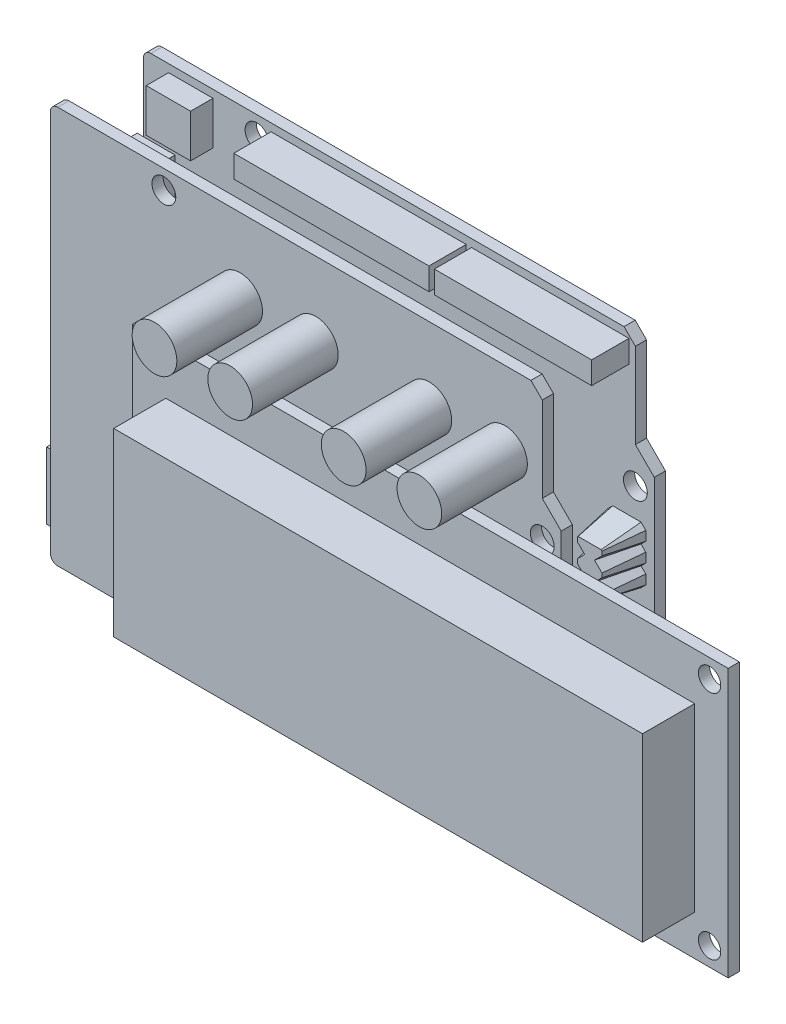
SolidWorks part; units mm, degrees
material "FR4 /26"
ref_plane "Front Plane" through (0, 0, 0) normal (0, 0, 1) x (1, 0, 0)
ref_plane "Top Plane" through (0, 0, 0) normal (0, 1, 0) x (1, 0, 0)
ref_plane "Right Plane" through (0, 0, 0) normal (1, 0, 0) x (0, 0, -1)
sketch "PCB" plane through (0, 0, 0) normal (0, 0, 1) x (1, 0, 0)
  line L0 (64.516, 53.34) -> (66.04, 51.816)
  line L1 (66.04, 40.386) -> (68.58, 37.846)
  line L2 (68.58, 37.846) -> (68.58, 5.08)
  line L3 (68.58, 5.08) -> (66.04, 2.54)
  line L4 (66.04, 2.54) -> (66.04, 1)
  line L5 (65.04, 0) -> (1, 0)
  line L6 (0, 1) -> (0, 52.34)
  line L7 (1, 53.34) -> (64.516, 53.34)
  line L8 (66.04, 51.816) -> (66.04, 40.386)
  circle A0 centre (66.04, 35.56) radius 1.6
  circle A1 centre (66.04, 7.62) radius 1.6
  circle A2 centre (15.24, 50.8) radius 1.6
  circle A3 centre (13.97, 2.54) radius 1.6
  arc A22 (65.04, 0) -> (66.04, 1) centre (65.04, 1) ccw
  arc A27 (0, 1) -> (1, 0) centre (1, 1) ccw
  arc A32 (1, 53.34) -> (0, 52.34) centre (1, 52.34) ccw
  dimension "D1" = 1
  dimension "D4" = 3.2
  dimension "D2" = 53.34
  dimension "D3" = 68.58
sketch "Components" plane through (0, 0, 0) normal (0, 0, 1) x (1, 0, 0)
  line L0 (38.481, 45.085) -> (28.448, 45.085)
  line L1 (28.448, 45.085) -> (27.94, 45.593)
  line L2 (59.182, 45.085) -> (49.149, 45.085)
  line L3 (59.69, 45.593) -> (59.182, 45.085)
  line L4 (2.4638, 35.282) -> (0.4318, 35.282)
  line L5 (1.905, 1.905) -> (3.175, 1.905)
  line L6 (4.191, 1.905) -> (5.08, 1.905)
  line L7 (5.08, 1.27) -> (6.35, 1.27)
  line L8 (0.635, 1.27) -> (1.905, 1.27)
  line L9 (1.27, 1.905) -> (1.27, 0.635)
  line L10 (33.655, 57.15) -> (33.655, 58.42)
  line L11 (33.655, 58.42) -> (36.83, 58.42)
  line L12 (36.83, 58.42) -> (36.83, 57.15)
  line L13 (31.115, 57.15) -> (31.115, 60.96)
  line L14 (31.115, 60.96) -> (48.26, 60.96)
  line L15 (48.26, 60.96) -> (48.26, 57.15)
  line L134 (28.6421, 46.7594) -> (28.2692, 47.1323)
  line L135 (28.2692, 47.1323) -> (29.3878, 47.1323)
  line L136 (29.3878, 46.7594) -> (29.3878, 47.5051)
  line L137 (28.4557, 47.9288) -> (28.2692, 48.1152)
  line L138 (28.2692, 48.1152) -> (28.2692, 48.4881)
  line L139 (28.2692, 48.4881) -> (28.4557, 48.6745)
  line L140 (28.4557, 48.6745) -> (28.6421, 48.6745)
  line L141 (28.6421, 48.6745) -> (28.8285, 48.4881)
  line L142 (28.8285, 48.4881) -> (28.8285, 48.3017)
  line L143 (28.8285, 48.4881) -> (29.015, 48.6745)
  line L144 (29.015, 48.6745) -> (29.2014, 48.6745)
  line L145 (29.2014, 48.6745) -> (29.3878, 48.4881)
  line L146 (29.3878, 48.4881) -> (29.3878, 48.1152)
  line L147 (29.3878, 48.1152) -> (29.2014, 47.9288)
  line L148 (31.1821, 46.7594) -> (30.8092, 47.1323)
  line L149 (30.8092, 47.1323) -> (31.9278, 47.1323)
  line L150 (31.9278, 46.7594) -> (31.9278, 47.5051)
  line L151 (31.9278, 48.6745) -> (31.9278, 47.9288)
  line L152 (31.9278, 47.9288) -> (31.1821, 48.6745)
  line L153 (31.1821, 48.6745) -> (30.9957, 48.6745)
  line L154 (30.9957, 48.6745) -> (30.8092, 48.4881)
  line L155 (30.8092, 48.4881) -> (30.8092, 48.1152)
  line L156 (30.8092, 48.1152) -> (30.9957, 47.9288)
  line L157 (33.7221, 46.7594) -> (33.3492, 47.1323)
  line L158 (33.3492, 47.1323) -> (34.4678, 47.1323)
  line L159 (34.4678, 46.7594) -> (34.4678, 47.5051)
  line L160 (33.7221, 47.9288) -> (33.3492, 48.3017)
  line L161 (33.3492, 48.3017) -> (34.4678, 48.3017)
  line L162 (34.4678, 47.9288) -> (34.4678, 48.6745)
  line L163 (36.2621, 46.7594) -> (35.8892, 47.1323)
  line L164 (35.8892, 47.1323) -> (37.0078, 47.1323)
  line L165 (37.0078, 46.7594) -> (37.0078, 47.5051)
  line L166 (36.8214, 47.9288) -> (36.0757, 47.9288)
  line L167 (36.0757, 47.9288) -> (35.8892, 48.1152)
  line L168 (35.8892, 48.1152) -> (35.8892, 48.4881)
  line L169 (35.8892, 48.4881) -> (36.0757, 48.6745)
  line L170 (36.0757, 48.6745) -> (36.8214, 48.6745)
  line L171 (36.8214, 48.6745) -> (37.0078, 48.4881)
  line L172 (37.0078, 48.4881) -> (37.0078, 48.1152)
  line L173 (37.0078, 48.1152) -> (36.8214, 47.9288)
  line L174 (36.8214, 47.9288) -> (36.0757, 48.6745)
  line L175 (39.3614, 47.9288) -> (39.5478, 48.1152)
  line L176 (39.5478, 48.1152) -> (39.5478, 48.4881)
  line L177 (39.5478, 48.4881) -> (39.3614, 48.6745)
  line L178 (39.3614, 48.6745) -> (38.6157, 48.6745)
  line L179 (38.6157, 48.6745) -> (38.4292, 48.4881)
  line L180 (38.4292, 48.4881) -> (38.4292, 48.1152)
  line L181 (38.4292, 48.1152) -> (38.6157, 47.9288)
  line L182 (38.6157, 47.9288) -> (38.8021, 47.9288)
  line L183 (38.8021, 47.9288) -> (38.9885, 48.1152)
  line L184 (38.9885, 48.1152) -> (38.9885, 48.6745)
  line L185 (41.1557, 47.9288) -> (40.9692, 48.1152)
  line L186 (40.9692, 48.1152) -> (40.9692, 48.4881)
  line L187 (40.9692, 48.4881) -> (41.1557, 48.6745)
  line L188 (41.1557, 48.6745) -> (41.3421, 48.6745)
  line L189 (41.3421, 48.6745) -> (41.5285, 48.4881)
  line L190 (41.5285, 48.4881) -> (41.715, 48.6745)
  line L191 (41.715, 48.6745) -> (41.9014, 48.6745)
  line L192 (41.9014, 48.6745) -> (42.0878, 48.4881)
  line L193 (42.0878, 48.4881) -> (42.0878, 48.1152)
  line L194 (42.0878, 48.1152) -> (41.9014, 47.9288)
  line L195 (41.9014, 47.9288) -> (41.715, 47.9288)
  line L196 (41.715, 47.9288) -> (41.5285, 48.1152)
  line L197 (41.5285, 48.1152) -> (41.3421, 47.9288)
  line L198 (41.3421, 47.9288) -> (41.1557, 47.9288)
  line L199 (41.5285, 48.1152) -> (41.5285, 48.4881)
  line L200 (45.0332, 47.9288) -> (45.0332, 48.6745)
  line L201 (45.0332, 48.6745) -> (45.2197, 48.6745)
  line L202 (45.2197, 48.6745) -> (45.9654, 47.9288)
  line L203 (45.9654, 47.9288) -> (46.1518, 47.9288)
  line L204 (47.5732, 48.6745) -> (47.7597, 48.3017)
  line L205 (47.7597, 48.3017) -> (48.1325, 47.9288)
  line L206 (48.1325, 47.9288) -> (48.5054, 47.9288)
  line L207 (48.5054, 47.9288) -> (48.6918, 48.1152)
  line L208 (48.6918, 48.1152) -> (48.6918, 48.4881)
  line L209 (48.6918, 48.4881) -> (48.5054, 48.6745)
  line L210 (48.5054, 48.6745) -> (48.319, 48.6745)
  line L211 (48.319, 48.6745) -> (48.1325, 48.4881)
  line L212 (48.1325, 48.4881) -> (48.1325, 47.9288)
  line L213 (50.1132, 48.6745) -> (50.1132, 47.9288)
  line L214 (50.1132, 47.9288) -> (50.6725, 47.9288)
  line L215 (50.6725, 47.9288) -> (50.4861, 48.3017)
  line L216 (50.4861, 48.3017) -> (50.4861, 48.4881)
  line L217 (50.4861, 48.4881) -> (50.6725, 48.6745)
  line L218 (50.6725, 48.6745) -> (51.0454, 48.6745)
  line L219 (51.0454, 48.6745) -> (51.2318, 48.4881)
  line L220 (51.2318, 48.4881) -> (51.2318, 48.1152)
  line L221 (51.2318, 48.1152) -> (51.0454, 47.9288)
  line L222 (53.7718, 48.4881) -> (52.6532, 48.4881)
  line L223 (52.6532, 48.4881) -> (53.2125, 47.9288)
  line L224 (53.2125, 47.9288) -> (53.2125, 48.6745)
  line L225 (55.3797, 47.9288) -> (55.1932, 48.1152)
  line L226 (55.1932, 48.1152) -> (55.1932, 48.4881)
  line L227 (55.1932, 48.4881) -> (55.3797, 48.6745)
  line L228 (55.3797, 48.6745) -> (55.5661, 48.6745)
  line L229 (55.5661, 48.6745) -> (55.7525, 48.4881)
  line L230 (55.7525, 48.4881) -> (55.7525, 48.3017)
  line L231 (55.7525, 48.4881) -> (55.939, 48.6745)
  line L232 (55.939, 48.6745) -> (56.1254, 48.6745)
  line L233 (56.1254, 48.6745) -> (56.3118, 48.4881)
  line L234 (56.3118, 48.4881) -> (56.3118, 48.1152)
  line L235 (56.3118, 48.1152) -> (56.1254, 47.9288)
  line L236 (58.8518, 48.6745) -> (58.8518, 47.9288)
  line L237 (58.8518, 47.9288) -> (58.1061, 48.6745)
  line L238 (58.1061, 48.6745) -> (57.9197, 48.6745)
  line L239 (57.9197, 48.6745) -> (57.7332, 48.4881)
  line L240 (57.7332, 48.4881) -> (57.7332, 48.1152)
  line L241 (57.7332, 48.1152) -> (57.9197, 47.9288)
  line L242 (60.6461, 47.9288) -> (60.2732, 48.3017)
  line L243 (60.2732, 48.3017) -> (61.3918, 48.3017)
  line L244 (61.3918, 47.9288) -> (61.3918, 48.6745)
  line L245 (63.7454, 47.9288) -> (62.9997, 47.9288)
  line L246 (62.9997, 47.9288) -> (62.8132, 48.1152)
  line L247 (62.8132, 48.1152) -> (62.8132, 48.4881)
  line L248 (62.8132, 48.4881) -> (62.9997, 48.6745)
  line L249 (62.9997, 48.6745) -> (63.7454, 48.6745)
  line L250 (63.7454, 48.6745) -> (63.9318, 48.4881)
  line L251 (63.9318, 48.4881) -> (63.9318, 48.1152)
  line L252 (63.9318, 48.1152) -> (63.7454, 47.9288)
  line L253 (63.7454, 47.9288) -> (62.9997, 48.6745)
  line L254 (0.7112, 13.3355) -> (1.4569, 13.3355)
  line L255 (1.084, 13.7083) -> (1.084, 12.9626)
  line L256 (1.8806, 13.8948) -> (1.8806, 13.1491)
  line L257 (1.8806, 13.1491) -> (2.2534, 12.7762)
  line L258 (2.2534, 12.7762) -> (2.6263, 13.1491)
  line L259 (2.6263, 13.1491) -> (2.6263, 13.8948)
  line L260 (3.05, 12.7762) -> (3.4228, 12.7762)
  line L261 (3.2364, 12.7762) -> (3.2364, 13.8948)
  line L262 (3.05, 13.8948) -> (3.4228, 13.8948)
  line L263 (3.8296, 12.7762) -> (3.8296, 13.8948)
  line L264 (3.8296, 13.8948) -> (4.5753, 12.7762)
  line L265 (4.5753, 12.7762) -> (4.5753, 13.8948)
  line L266 (15.3162, 12.5735) -> (16.0619, 12.5735)
  line L267 (23.495, 9.8806) -> (23.495, 5.3594)
  line L268 (19.685, 9.8806) -> (19.685, 5.3594)
  line L269 (22.59, 7.427) -> (21.59, 8.45)
  line L270 (21.59, 8.45) -> (20.59, 7.427)
  line L271 (20.59, 7.427) -> (22.59, 7.427)
  line L272 (59.428, 26.17) -> (58.928, 27.17)
  line L273 (58.928, 27.17) -> (58.428, 26.17)
  line L274 (58.428, 26.17) -> (59.428, 26.17)
  line L275 (11.684, 4.8245) -> (11.684, 2.602)
  line L276 (11.684, 2.602) -> (11.3665, 2.602)
  line L277 (11.684, 10.222) -> (11.684, 11.5936)
  line L278 (11.684, 11.5936) -> (1.6764, 11.5936)
  line L279 (1.6764, 11.5936) -> (-1.8034, 11.5936)
  line L280 (-1.8034, 11.5936) -> (-1.8034, 2.602)
  line L281 (-1.8034, 2.602) -> (5.969, 2.602)
  line L282 (1.6764, 2.6274) -> (1.6764, 11.5936)
  line L283 (14.732, 20.4216) -> (18.288, 20.4216)
  line L284 (18.288, 20.4216) -> (18.288, 13.8684)
  line L285 (18.288, 13.8684) -> (14.732, 13.8684)
  line L286 (14.732, 13.8684) -> (14.732, 20.4216)
  line L287 (22.579, 35.589) -> (22.579, 32.989)
  line L288 (19.329, 32.989) -> (19.329, 35.589)
  line L289 (19.614, 32.664) -> (19.751, 32.664)
  line L290 (20.208, 32.664) -> (20.401, 32.664)
  line L291 (20.858, 32.664) -> (21.051, 32.664)
  line L292 (21.508, 32.664) -> (21.701, 32.664)
  line L293 (22.158, 32.664) -> (22.254, 32.664)
  line L294 (19.654, 35.914) -> (19.751, 35.914)
  line L295 (20.208, 35.914) -> (20.401, 35.914)
  line L296 (20.858, 35.914) -> (21.051, 35.914)
  line L297 (21.508, 35.914) -> (21.701, 35.914)
  line L298 (22.158, 35.914) -> (22.254, 35.914)
  line L299 (62.992, 31.75) -> (62.357, 31.115)
  line L300 (62.357, 29.845) -> (62.992, 29.21)
  line L301 (62.992, 29.21) -> (62.357, 28.575)
  line L302 (62.357, 27.305) -> (62.992, 26.67)
  line L303 (62.992, 31.75) -> (66.802, 31.75)
  line L304 (66.802, 31.75) -> (67.437, 31.115)
  line L305 (67.437, 31.115) -> (67.437, 29.845)
  line L306 (67.437, 29.845) -> (66.802, 29.21)
  line L307 (66.802, 29.21) -> (67.437, 28.575)
  line L308 (67.437, 28.575) -> (67.437, 27.305)
  line L309 (67.437, 27.305) -> (66.802, 26.67)
  line L310 (66.802, 29.21) -> (62.992, 29.21)
  line L311 (66.802, 26.67) -> (62.992, 26.67)
  line L312 (62.357, 28.575) -> (62.357, 27.305)
  line L313 (62.357, 31.115) -> (62.357, 29.845)
  line L314 (62.992, 26.67) -> (62.357, 26.035)
  line L315 (62.357, 24.765) -> (62.992, 24.13)
  line L316 (66.802, 26.67) -> (67.437, 26.035)
  line L317 (67.437, 26.035) -> (67.437, 24.765)
  line L318 (67.437, 24.765) -> (66.802, 24.13)
  line L319 (66.802, 24.13) -> (62.992, 24.13)
  line L320 (62.357, 26.035) -> (62.357, 24.765)
  line L321 (0, 43.664) -> (0, 42.5923)
  line L322 (0, 41.5923) -> (0, 40.5207)
  line L323 (0, 39.5207) -> (0, 38.449)
  line L324 (0, 37.449) -> (0, 36.3773)
  line L325 (0, 35.3773) -> (0, 34.3057)
  line L326 (0, 31.8057) -> (0, 30.734)
  line L327 (4.2418, 43.156) -> (4.2418, 36.044)
  line L328 (4.2418, 36.044) -> (2.4638, 36.044)
  line L329 (2.4638, 36.044) -> (2.4638, 35.282)
  line L331 (0.4318, 35.282) -> (0.4318, 36.044)
  line L332 (0.4318, 36.044) -> (-0.8382, 36.044)
  line L333 (-0.8382, 36.044) -> (-0.8382, 43.156)
  line L334 (-0.8382, 43.156) -> (0.4318, 43.156)
  line L335 (0.4318, 43.156) -> (0.4318, 43.918)
  line L336 (0.4318, 43.918) -> (2.4638, 43.918)
  line L337 (2.4638, 43.918) -> (2.4638, 43.156)
  line L338 (2.4638, 43.156) -> (4.2418, 43.156)
  line L339 (48.895, 49.53) -> (47.625, 49.53)
  line L340 (47.625, 49.53) -> (46.99, 50.165)
  line L341 (46.99, 50.165) -> (46.99, 51.435)
  line L342 (46.99, 51.435) -> (47.625, 52.07)
  line L343 (52.07, 50.165) -> (51.435, 49.53)
  line L344 (51.435, 49.53) -> (50.165, 49.53)
  line L345 (50.165, 49.53) -> (49.53, 50.165)
  line L346 (49.53, 50.165) -> (49.53, 51.435)
  line L347 (49.53, 51.435) -> (50.165, 52.07)
  line L348 (50.165, 52.07) -> (51.435, 52.07)
  line L349 (51.435, 52.07) -> (52.07, 51.435)
  line L350 (48.895, 49.53) -> (49.53, 50.165)
  line L351 (49.53, 51.435) -> (48.895, 52.07)
  line L352 (47.625, 52.07) -> (48.895, 52.07)
  line L353 (56.515, 49.53) -> (55.245, 49.53)
  line L354 (55.245, 49.53) -> (54.61, 50.165)
  line L355 (54.61, 50.165) -> (54.61, 51.435)
  line L356 (54.61, 51.435) -> (55.245, 52.07)
  line L357 (54.61, 50.165) -> (53.975, 49.53)
  line L358 (53.975, 49.53) -> (52.705, 49.53)
  line L359 (52.705, 49.53) -> (52.07, 50.165)
  line L360 (52.07, 50.165) -> (52.07, 51.435)
  line L361 (52.07, 51.435) -> (52.705, 52.07)
  line L362 (52.705, 52.07) -> (53.975, 52.07)
  line L363 (53.975, 52.07) -> (54.61, 51.435)
  line L364 (59.69, 50.165) -> (59.055, 49.53)
  line L365 (59.055, 49.53) -> (57.785, 49.53)
  line L366 (57.785, 49.53) -> (57.15, 50.165)
  line L367 (57.15, 50.165) -> (57.15, 51.435)
  line L368 (57.15, 51.435) -> (57.785, 52.07)
  line L369 (57.785, 52.07) -> (59.055, 52.07)
  line L370 (59.055, 52.07) -> (59.69, 51.435)
  line L371 (56.515, 49.53) -> (57.15, 50.165)
  line L372 (57.15, 51.435) -> (56.515, 52.07)
  line L373 (55.245, 52.07) -> (56.515, 52.07)
  line L374 (64.135, 49.53) -> (62.865, 49.53)
  line L375 (62.865, 49.53) -> (62.23, 50.165)
  line L376 (62.23, 50.165) -> (62.23, 51.435)
  line L377 (62.23, 51.435) -> (62.865, 52.07)
  line L378 (62.23, 50.165) -> (61.595, 49.53)
  line L379 (61.595, 49.53) -> (60.325, 49.53)
  line L380 (60.325, 49.53) -> (59.69, 50.165)
  line L381 (59.69, 50.165) -> (59.69, 51.435)
  line L382 (59.69, 51.435) -> (60.325, 52.07)
  line L383 (60.325, 52.07) -> (61.595, 52.07)
  line L384 (61.595, 52.07) -> (62.23, 51.435)
  line L385 (64.77, 50.165) -> (64.77, 51.435)
  line L386 (64.135, 49.53) -> (64.77, 50.165)
  line L387 (64.77, 51.435) -> (64.135, 52.07)
  line L388 (62.865, 52.07) -> (64.135, 52.07)
  line L389 (46.355, 49.53) -> (45.085, 49.53)
  line L390 (45.085, 49.53) -> (44.45, 50.165)
  line L391 (44.45, 50.165) -> (44.45, 51.435)
  line L392 (44.45, 51.435) -> (45.085, 52.07)
  line L393 (46.355, 49.53) -> (46.99, 50.165)
  line L394 (46.99, 51.435) -> (46.355, 52.07)
  line L395 (45.085, 52.07) -> (46.355, 52.07)
  line L396 (42.545, 3.81) -> (43.815, 3.81)
  line L397 (43.815, 3.81) -> (44.45, 3.175)
  line L398 (44.45, 3.175) -> (44.45, 1.905)
  line L399 (44.45, 1.905) -> (43.815, 1.27)
  line L400 (39.37, 3.175) -> (40.005, 3.81)
  line L401 (40.005, 3.81) -> (41.275, 3.81)
  line L402 (41.275, 3.81) -> (41.91, 3.175)
  line L403 (41.91, 3.175) -> (41.91, 1.905)
  line L404 (41.91, 1.905) -> (41.275, 1.27)
  line L405 (41.275, 1.27) -> (40.005, 1.27)
  line L406 (40.005, 1.27) -> (39.37, 1.905)
  line L407 (42.545, 3.81) -> (41.91, 3.175)
  line L408 (41.91, 1.905) -> (42.545, 1.27)
  line L409 (43.815, 1.27) -> (42.545, 1.27)
  line L410 (34.925, 3.81) -> (36.195, 3.81)
  line L411 (36.195, 3.81) -> (36.83, 3.175)
  line L412 (36.83, 3.175) -> (36.83, 1.905)
  line L413 (36.83, 1.905) -> (36.195, 1.27)
  line L414 (36.83, 3.175) -> (37.465, 3.81)
  line L415 (37.465, 3.81) -> (38.735, 3.81)
  line L416 (38.735, 3.81) -> (39.37, 3.175)
  line L417 (39.37, 3.175) -> (39.37, 1.905)
  line L418 (39.37, 1.905) -> (38.735, 1.27)
  line L419 (38.735, 1.27) -> (37.465, 1.27)
  line L420 (37.465, 1.27) -> (36.83, 1.905)
  line L421 (31.75, 3.175) -> (32.385, 3.81)
  line L422 (32.385, 3.81) -> (33.655, 3.81)
  line L423 (33.655, 3.81) -> (34.29, 3.175)
  line L424 (34.29, 3.175) -> (34.29, 1.905)
  line L425 (34.29, 1.905) -> (33.655, 1.27)
  line L426 (33.655, 1.27) -> (32.385, 1.27)
  line L427 (32.385, 1.27) -> (31.75, 1.905)
  line L428 (34.925, 3.81) -> (34.29, 3.175)
  line L429 (34.29, 1.905) -> (34.925, 1.27)
  line L430 (36.195, 1.27) -> (34.925, 1.27)
  line L431 (27.305, 3.81) -> (28.575, 3.81)
  line L432 (28.575, 3.81) -> (29.21, 3.175)
  line L433 (29.21, 3.175) -> (29.21, 1.905)
  line L434 (29.21, 1.905) -> (28.575, 1.27)
  line L435 (29.21, 3.175) -> (29.845, 3.81)
  line L436 (29.845, 3.81) -> (31.115, 3.81)
  line L437 (31.115, 3.81) -> (31.75, 3.175)
  line L438 (31.75, 3.175) -> (31.75, 1.905)
  line L439 (31.75, 1.905) -> (31.115, 1.27)
  line L440 (31.115, 1.27) -> (29.845, 1.27)
  line L441 (29.845, 1.27) -> (29.21, 1.905)
  line L442 (26.67, 3.175) -> (26.67, 1.905)
  line L443 (27.305, 3.81) -> (26.67, 3.175)
  line L444 (26.67, 1.905) -> (27.305, 1.27)
  line L445 (28.575, 1.27) -> (27.305, 1.27)
  line L446 (45.085, 3.81) -> (46.355, 3.81)
  line L447 (46.355, 3.81) -> (46.99, 3.175)
  line L448 (46.99, 3.175) -> (46.99, 1.905)
  line L449 (46.99, 1.905) -> (46.355, 1.27)
  line L450 (45.085, 3.81) -> (44.45, 3.175)
  line L451 (44.45, 1.905) -> (45.085, 1.27)
  line L452 (46.355, 1.27) -> (45.085, 1.27)
  line L453 (57.785, 3.81) -> (59.055, 3.81)
  line L454 (59.055, 3.81) -> (59.69, 3.175)
  line L455 (59.69, 3.175) -> (59.69, 1.905)
  line L456 (59.69, 1.905) -> (59.055, 1.27)
  line L457 (59.69, 3.175) -> (60.325, 3.81)
  line L458 (60.325, 3.81) -> (61.595, 3.81)
  line L459 (61.595, 3.81) -> (62.23, 3.175)
  line L460 (62.23, 3.175) -> (62.23, 1.905)
  line L461 (62.23, 1.905) -> (61.595, 1.27)
  line L462 (61.595, 1.27) -> (60.325, 1.27)
  line L463 (60.325, 1.27) -> (59.69, 1.905)
  line L464 (54.61, 3.175) -> (55.245, 3.81)
  line L465 (55.245, 3.81) -> (56.515, 3.81)
  line L466 (56.515, 3.81) -> (57.15, 3.175)
  line L467 (57.15, 3.175) -> (57.15, 1.905)
  line L468 (57.15, 1.905) -> (56.515, 1.27)
  line L469 (56.515, 1.27) -> (55.245, 1.27)
  line L470 (55.245, 1.27) -> (54.61, 1.905)
  line L471 (57.785, 3.81) -> (57.15, 3.175)
  line L472 (57.15, 1.905) -> (57.785, 1.27)
  line L473 (59.055, 1.27) -> (57.785, 1.27)
  line L474 (50.165, 3.81) -> (51.435, 3.81)
  line L475 (51.435, 3.81) -> (52.07, 3.175)
  line L476 (52.07, 3.175) -> (52.07, 1.905)
  line L477 (52.07, 1.905) -> (51.435, 1.27)
  line L478 (52.07, 3.175) -> (52.705, 3.81)
  line L479 (52.705, 3.81) -> (53.975, 3.81)
  line L480 (53.975, 3.81) -> (54.61, 3.175)
  line L481 (54.61, 3.175) -> (54.61, 1.905)
  line L482 (54.61, 1.905) -> (53.975, 1.27)
  line L483 (53.975, 1.27) -> (52.705, 1.27)
  line L484 (52.705, 1.27) -> (52.07, 1.905)
  line L485 (49.53, 3.175) -> (49.53, 1.905)
  line L486 (50.165, 3.81) -> (49.53, 3.175)
  line L487 (49.53, 1.905) -> (50.165, 1.27)
  line L488 (51.435, 1.27) -> (50.165, 1.27)
  line L489 (62.865, 3.81) -> (64.135, 3.81)
  line L490 (64.135, 3.81) -> (64.77, 3.175)
  line L491 (64.77, 3.175) -> (64.77, 1.905)
  line L492 (64.77, 1.905) -> (64.135, 1.27)
  line L493 (62.865, 3.81) -> (62.23, 3.175)
  line L494 (62.23, 1.905) -> (62.865, 1.27)
  line L495 (64.135, 1.27) -> (62.865, 1.27)
  line L496 (22.606, 50.165) -> (21.971, 49.53)
  line L497 (21.971, 49.53) -> (20.701, 49.53)
  line L498 (20.701, 49.53) -> (20.066, 50.165)
  line L499 (20.066, 50.165) -> (20.066, 51.435)
  line L500 (20.066, 51.435) -> (20.701, 52.07)
  line L501 (20.701, 52.07) -> (21.971, 52.07)
  line L502 (21.971, 52.07) -> (22.606, 51.435)
  line L503 (27.051, 49.53) -> (25.781, 49.53)
  line L504 (25.781, 49.53) -> (25.146, 50.165)
  line L505 (25.146, 50.165) -> (25.146, 51.435)
  line L506 (25.146, 51.435) -> (25.781, 52.07)
  line L507 (25.146, 50.165) -> (24.511, 49.53)
  line L508 (24.511, 49.53) -> (23.241, 49.53)
  line L509 (23.241, 49.53) -> (22.606, 50.165)
  line L510 (22.606, 50.165) -> (22.606, 51.435)
  line L511 (22.606, 51.435) -> (23.241, 52.07)
  line L512 (23.241, 52.07) -> (24.511, 52.07)
  line L513 (24.511, 52.07) -> (25.146, 51.435)
  line L514 (30.226, 50.165) -> (29.591, 49.53)
  line L515 (29.591, 49.53) -> (28.321, 49.53)
  line L516 (28.321, 49.53) -> (27.686, 50.165)
  line L517 (27.686, 50.165) -> (27.686, 51.435)
  line L518 (27.686, 51.435) -> (28.321, 52.07)
  line L519 (28.321, 52.07) -> (29.591, 52.07)
  line L520 (29.591, 52.07) -> (30.226, 51.435)
  line L521 (27.051, 49.53) -> (27.686, 50.165)
  line L522 (27.686, 51.435) -> (27.051, 52.07)
  line L523 (25.781, 52.07) -> (27.051, 52.07)
  line L524 (34.671, 49.53) -> (33.401, 49.53)
  line L525 (33.401, 49.53) -> (32.766, 50.165)
  line L526 (32.766, 50.165) -> (32.766, 51.435)
  line L527 (32.766, 51.435) -> (33.401, 52.07)
  line L528 (32.766, 50.165) -> (32.131, 49.53)
  line L529 (32.131, 49.53) -> (30.861, 49.53)
  line L530 (30.861, 49.53) -> (30.226, 50.165)
  line L531 (30.226, 50.165) -> (30.226, 51.435)
  line L532 (30.226, 51.435) -> (30.861, 52.07)
  line L533 (30.861, 52.07) -> (32.131, 52.07)
  line L534 (32.131, 52.07) -> (32.766, 51.435)
  line L535 (37.846, 50.165) -> (37.211, 49.53)
  line L536 (37.211, 49.53) -> (35.941, 49.53)
  line L537 (35.941, 49.53) -> (35.306, 50.165)
  line L538 (35.306, 50.165) -> (35.306, 51.435)
  line L539 (35.306, 51.435) -> (35.941, 52.07)
  line L540 (35.941, 52.07) -> (37.211, 52.07)
  line L541 (37.211, 52.07) -> (37.846, 51.435)
  line L542 (34.671, 49.53) -> (35.306, 50.165)
  line L543 (35.306, 51.435) -> (34.671, 52.07)
  line L544 (33.401, 52.07) -> (34.671, 52.07)
  line L545 (42.291, 49.53) -> (41.021, 49.53)
  line L546 (41.021, 49.53) -> (40.386, 50.165)
  line L547 (40.386, 50.165) -> (40.386, 51.435)
  line L548 (40.386, 51.435) -> (41.021, 52.07)
  line L549 (40.386, 50.165) -> (39.751, 49.53)
  line L550 (39.751, 49.53) -> (38.481, 49.53)
  line L551 (38.481, 49.53) -> (37.846, 50.165)
  line L552 (37.846, 50.165) -> (37.846, 51.435)
  line L553 (37.846, 51.435) -> (38.481, 52.07)
  line L554 (38.481, 52.07) -> (39.751, 52.07)
  line L555 (39.751, 52.07) -> (40.386, 51.435)
  line L556 (42.926, 50.165) -> (42.926, 51.435)
  line L557 (42.291, 49.53) -> (42.926, 50.165)
  line L558 (42.926, 51.435) -> (42.291, 52.07)
  line L559 (41.021, 52.07) -> (42.291, 52.07)
  line L560 (19.431, 49.53) -> (18.161, 49.53)
  line L561 (18.161, 49.53) -> (17.526, 50.165)
  line L562 (17.526, 50.165) -> (17.526, 51.435)
  line L563 (17.526, 51.435) -> (18.161, 52.07)
  line L564 (19.431, 49.53) -> (20.066, 50.165)
  line L565 (20.066, 51.435) -> (19.431, 52.07)
  line L566 (18.161, 52.07) -> (19.431, 52.07)
  line L567 (3.2512, 22.4038) -> (3.2512, 21.2852)
  line L568 (3.2512, 21.2852) -> (3.9969, 21.2852)
  line L569 (55.245, 27.97) -> (55.245, 25.47)
  line L570 (55.87, 27.67) -> (55.87, 25.67)
  line L571 (54.62, 25.67) -> (54.62, 27.67)
  line L572 (11.4, 32.385) -> (13.9, 32.385)
  line L573 (11.7, 33.01) -> (13.7, 33.01)
  line L574 (13.7, 31.76) -> (11.7, 31.76)
  line L575 (3.8867, 18.7336) -> (3.4715, 18.7336)
  line L576 (3.4715, 18.7336) -> (3.2639, 18.526)
  line L577 (3.2639, 18.526) -> (3.2639, 17.6955)
  line L578 (3.2639, 17.6955) -> (3.4715, 17.4879)
  line L579 (3.4715, 17.4879) -> (3.8867, 17.4879)
  line L580 (3.8867, 17.4879) -> (4.0943, 17.6955)
  line L581 (4.0943, 17.6955) -> (4.0943, 18.526)
  line L582 (4.0943, 18.526) -> (3.8867, 18.7336)
  line L583 (4.5736, 17.4879) -> (4.5736, 18.7336)
  line L584 (4.5736, 18.7336) -> (5.4041, 17.4879)
  line L585 (5.4041, 17.4879) -> (5.4041, 18.7336)
  line L586 (3.373, 52.292) -> (3.373, 46.514)
  line L587 (9.327, 46.514) -> (9.327, 48.903)
  line L588 (9.327, 49.903) -> (9.327, 52.292)
  line L589 (9.327, 48.903) -> (9.577, 48.903)
  line L590 (9.577, 48.903) -> (9.577, 49.903)
  line L591 (9.577, 49.903) -> (9.327, 49.903)
  line L592 (5.35, 52.492) -> (7.35, 52.492)
  line L594 (5.35, 46.514) -> (5.35, 46.314)
  line L595 (5.35, 46.314) -> (7.35, 46.314)
  line L596 (7.35, 46.314) -> (7.35, 46.514)
  line L599 (5.35, 52.492) -> (5.35, 52.292)
  line L603 (7.35, 52.292) -> (7.35, 52.492)
  line L604 (9.327, 46.514) -> (7.35, 46.514)
  line L605 (5.35, 46.514) -> (3.373, 46.514)
  line L606 (5.35, 52.292) -> (3.373, 52.292)
  line L607 (7.35, 52.292) -> (9.327, 52.292)
  line L608 (18.161, 29.9974) -> (18.161, 27.1018)
  line L609 (18.161, 27.1018) -> (17.399, 27.1018)
  line L610 (17.399, 27.1018) -> (17.399, 29.9974)
  line L611 (17.399, 29.9974) -> (18.161, 29.9974)
  line L612 (51.79, 12.11) -> (51.39, 11.71)
  line L613 (51.39, 11.71) -> (42.59, 11.71)
  line L614 (42.59, 11.71) -> (42.19, 12.11)
  line L615 (42.19, 12.11) -> (42.19, 20.91)
  line L616 (42.19, 20.91) -> (42.59, 21.31)
  line L617 (42.59, 21.31) -> (51.39, 21.31)
  line L618 (51.39, 21.31) -> (51.79, 20.91)
  line L619 (51.79, 20.91) -> (51.79, 12.11)
  line L620 (25.575, 15.723) -> (23.955, 15.723)
  line L621 (23.955, 18.567) -> (25.575, 18.567)
  line L622 (25.575, 17.667) -> (25.575, 16.623)
  line L623 (23.955, 17.573) -> (23.955, 17.667)
  line L624 (23.955, 16.623) -> (23.955, 16.717)
  line L625 (23.955, 18.473) -> (23.955, 18.567)
  line L626 (23.955, 15.723) -> (23.955, 15.817)
  line L627 (25.575, 15.817) -> (25.575, 15.723)
  line L628 (25.575, 18.567) -> (25.575, 18.473)
  line L629 (50.145, 26.975) -> (47.645, 26.975)
  line L630 (47.645, 26.975) -> (47.645, 30.175)
  line L631 (47.645, 30.175) -> (50.145, 30.175)
  line L632 (50.145, 30.175) -> (50.145, 26.975)
  line L633 (20.828, 18.1658) -> (20.828, 18.9786) construction
  line L634 (13.97, 19.05) -> (13.97, 19.8628) construction
  line L635 (20.828, 13.6924) -> (20.828, 14.2258) construction
  line L636 (20.8374, 15.8544) -> (20.8374, 16.6672) construction
  line L637 (0.1778, 34.774) -> (0.1778, 37.822) construction
  arc A0 (28.448, 45.1612) -> (28.448, 45.0088) centre (28.448, 45.085) ccw
  arc A1 (38.481, 45.0088) -> (38.481, 45.1612) centre (38.481, 45.085) ccw
  arc A2 (27.9939, 45.6469) -> (27.8861, 45.5391) centre (27.94, 45.593) ccw
  arc A3 (28.3941, 45.0311) -> (28.5019, 45.1389) centre (28.448, 45.085) ccw
  arc A4 (49.149, 45.1612) -> (49.149, 45.0088) centre (49.149, 45.085) ccw
  arc A5 (59.182, 45.0088) -> (59.182, 45.1612) centre (59.182, 45.085) ccw
  arc A6 (59.1281, 45.1389) -> (59.2359, 45.0311) centre (59.182, 45.085) ccw
  arc A7 (59.7439, 45.5391) -> (59.6361, 45.6469) centre (59.69, 45.593) ccw
  arc A10 (3.175, 1.8288) -> (3.175, 1.9812) centre (3.175, 1.905) ccw
  arc A11 (1.905, 1.9812) -> (1.905, 1.8288) centre (1.905, 1.905) ccw
  arc A12 (4.191, 1.905) -> (3.175, 2.221) centre (3.4259, 1.2364) ccw
  arc A13 (4.1148, 1.905) -> (4.2672, 1.905) centre (4.191, 1.905) ccw
  arc A14 (3.175, 2.2972) -> (3.175, 2.1448) centre (3.175, 2.221) ccw
  arc A15 (3.175, 0.889) -> (4.191, 1.905) centre (3.175, 1.905) ccw
  arc A16 (3.175, 0.9652) -> (3.175, 0.8128) centre (3.175, 0.889) ccw
  arc A17 (4.2672, 1.905) -> (4.1148, 1.905) centre (4.191, 1.905) ccw
  arc A18 (5.08, 1.8288) -> (5.08, 1.9812) centre (5.08, 1.905) ccw
  arc A19 (4.191, 1.9812) -> (4.191, 1.8288) centre (4.191, 1.905) ccw
  arc A20 (6.35, 1.1938) -> (6.35, 1.3462) centre (6.35, 1.27) ccw
  arc A21 (5.08, 1.3462) -> (5.08, 1.1938) centre (5.08, 1.27) ccw
  arc A22 (1.905, 1.1938) -> (1.905, 1.3462) centre (1.905, 1.27) ccw
  arc A23 (0.635, 1.3462) -> (0.635, 1.1938) centre (0.635, 1.27) ccw
  arc A24 (1.1938, 0.635) -> (1.3462, 0.635) centre (1.27, 0.635) ccw
  arc A25 (1.3462, 1.905) -> (1.1938, 1.905) centre (1.27, 1.905) ccw
  arc A26 (33.7312, 58.42) -> (33.5788, 58.42) centre (33.655, 58.42) ccw
  arc A27 (33.5788, 57.15) -> (33.7312, 57.15) centre (33.655, 57.15) ccw
  arc A28 (36.83, 58.3438) -> (36.83, 58.4962) centre (36.83, 58.42) ccw
  arc A29 (33.655, 58.4962) -> (33.655, 58.3438) centre (33.655, 58.42) ccw
  arc A30 (36.7538, 57.15) -> (36.9062, 57.15) centre (36.83, 57.15) ccw
  arc A31 (36.9062, 58.42) -> (36.7538, 58.42) centre (36.83, 58.42) ccw
  arc A32 (31.1912, 60.96) -> (31.0388, 60.96) centre (31.115, 60.96) ccw
  arc A33 (31.0388, 57.15) -> (31.1912, 57.15) centre (31.115, 57.15) ccw
  arc A34 (48.26, 60.8838) -> (48.26, 61.0362) centre (48.26, 60.96) ccw
  arc A35 (31.115, 61.0362) -> (31.115, 60.8838) centre (31.115, 60.96) ccw
  arc A36 (48.1838, 57.15) -> (48.3362, 57.15) centre (48.26, 57.15) ccw
  arc A37 (48.3362, 60.96) -> (48.1838, 60.96) centre (48.26, 60.96) ccw
  arc A274 (28.2962, 47.1592) -> (28.2423, 47.1053) centre (28.2693, 47.1322) ccw
  arc A275 (28.6152, 46.7325) -> (28.669, 46.7863) centre (28.6421, 46.7594) ccw
  arc A276 (29.3878, 47.0942) -> (29.3878, 47.1704) centre (29.3878, 47.1323) ccw
  arc A277 (28.2692, 47.1704) -> (28.2692, 47.0942) centre (28.2692, 47.1323) ccw
  arc A278 (29.4259, 47.5051) -> (29.3497, 47.5051) centre (29.3878, 47.5051) ccw
  arc A279 (29.3497, 46.7594) -> (29.4259, 46.7594) centre (29.3878, 46.7594) ccw
  arc A280 (28.2962, 48.1422) -> (28.2423, 48.0883) centre (28.2693, 48.1152) ccw
  arc A281 (28.4287, 47.9019) -> (28.4826, 47.9557) centre (28.4557, 47.9288) ccw
  arc A282 (28.3073, 48.4881) -> (28.2311, 48.4881) centre (28.2692, 48.4881) ccw
  arc A283 (28.2311, 48.1152) -> (28.3073, 48.1152) centre (28.2692, 48.1152) ccw
  arc A284 (28.4826, 48.6476) -> (28.4287, 48.7014) centre (28.4557, 48.6745) ccw
  arc A285 (28.2423, 48.515) -> (28.2962, 48.4611) centre (28.2693, 48.4881) ccw
  arc A286 (28.6421, 48.6364) -> (28.6421, 48.7126) centre (28.6421, 48.6745) ccw
  arc A287 (28.4557, 48.7126) -> (28.4557, 48.6364) centre (28.4557, 48.6745) ccw
  arc A288 (28.8016, 48.4611) -> (28.8555, 48.515) centre (28.8285, 48.4881) ccw
  arc A289 (28.669, 48.7014) -> (28.6152, 48.6476) centre (28.6421, 48.6745) ccw
  arc A290 (28.7904, 48.3017) -> (28.8666, 48.3017) centre (28.8285, 48.3017) ccw
  arc A291 (28.8666, 48.4881) -> (28.7904, 48.4881) centre (28.8285, 48.4881) ccw
  arc A292 (29.0419, 48.6476) -> (28.988, 48.7014) centre (29.0149, 48.6745) ccw
  arc A293 (28.8016, 48.515) -> (28.8555, 48.4611) centre (28.8285, 48.4881) ccw
  arc A294 (29.2014, 48.6364) -> (29.2014, 48.7126) centre (29.2014, 48.6745) ccw
  arc A295 (29.015, 48.7126) -> (29.015, 48.6364) centre (29.015, 48.6745) ccw
  arc A296 (29.3609, 48.4611) -> (29.4147, 48.515) centre (29.3878, 48.4881) ccw
  arc A297 (29.2283, 48.7014) -> (29.1744, 48.6476) centre (29.2014, 48.6745) ccw
  arc A298 (29.3497, 48.1152) -> (29.4259, 48.1152) centre (29.3878, 48.1152) ccw
  arc A299 (29.4259, 48.4881) -> (29.3497, 48.4881) centre (29.3878, 48.4881) ccw
  arc A300 (29.1744, 47.9557) -> (29.2283, 47.9019) centre (29.2014, 47.9288) ccw
  arc A301 (29.4147, 48.0883) -> (29.3609, 48.1422) centre (29.3878, 48.1152) ccw
  arc A302 (30.8362, 47.1592) -> (30.7823, 47.1053) centre (30.8092, 47.1322) ccw
  arc A303 (31.1552, 46.7325) -> (31.209, 46.7863) centre (31.1821, 46.7594) ccw
  arc A304 (31.9278, 47.0942) -> (31.9278, 47.1704) centre (31.9278, 47.1323) ccw
  arc A305 (30.8092, 47.1704) -> (30.8092, 47.0942) centre (30.8092, 47.1323) ccw
  arc A306 (31.9659, 47.5051) -> (31.8897, 47.5051) centre (31.9278, 47.5051) ccw
  arc A307 (31.8897, 46.7594) -> (31.9659, 46.7594) centre (31.9278, 46.7594) ccw
  arc A308 (31.8897, 47.9288) -> (31.9659, 47.9288) centre (31.9278, 47.9288) ccw
  arc A309 (31.9659, 48.6745) -> (31.8897, 48.6745) centre (31.9278, 48.6745) ccw
  arc A310 (31.209, 48.7014) -> (31.1552, 48.6476) centre (31.1821, 48.6745) ccw
  arc A311 (31.9009, 47.9019) -> (31.9547, 47.9557) centre (31.9278, 47.9288) ccw
  arc A312 (30.9957, 48.7126) -> (30.9957, 48.6364) centre (30.9957, 48.6745) ccw
  arc A313 (31.1821, 48.6364) -> (31.1821, 48.7126) centre (31.1821, 48.6745) ccw
  arc A314 (30.7823, 48.515) -> (30.8362, 48.4611) centre (30.8092, 48.4881) ccw
  arc A315 (31.0226, 48.6476) -> (30.9687, 48.7014) centre (30.9957, 48.6745) ccw
  arc A316 (30.7711, 48.1152) -> (30.8473, 48.1152) centre (30.8092, 48.1152) ccw
  arc A317 (30.8473, 48.4881) -> (30.7711, 48.4881) centre (30.8092, 48.4881) ccw
  arc A318 (30.9687, 47.9019) -> (31.0226, 47.9557) centre (30.9957, 47.9288) ccw
  arc A319 (30.8362, 48.1422) -> (30.7823, 48.0883) centre (30.8092, 48.1152) ccw
  arc A320 (33.3762, 47.1592) -> (33.3223, 47.1053) centre (33.3492, 47.1322) ccw
  arc A321 (33.6952, 46.7325) -> (33.749, 46.7863) centre (33.7221, 46.7594) ccw
  arc A322 (34.4678, 47.0942) -> (34.4678, 47.1704) centre (34.4678, 47.1323) ccw
  arc A323 (33.3492, 47.1704) -> (33.3492, 47.0942) centre (33.3492, 47.1323) ccw
  arc A324 (34.5059, 47.5051) -> (34.4297, 47.5051) centre (34.4678, 47.5051) ccw
  arc A325 (34.4297, 46.7594) -> (34.5059, 46.7594) centre (34.4678, 46.7594) ccw
  arc A326 (33.3762, 48.3286) -> (33.3223, 48.2747) centre (33.3492, 48.3017) ccw
  arc A327 (33.6952, 47.9019) -> (33.749, 47.9557) centre (33.7221, 47.9288) ccw
  arc A328 (34.4678, 48.2636) -> (34.4678, 48.3398) centre (34.4678, 48.3017) ccw
  arc A329 (33.3492, 48.3398) -> (33.3492, 48.2636) centre (33.3492, 48.3017) ccw
  arc A330 (34.5059, 48.6745) -> (34.4297, 48.6745) centre (34.4678, 48.6745) ccw
  arc A331 (34.4297, 47.9288) -> (34.5059, 47.9288) centre (34.4678, 47.9288) ccw
  arc A332 (35.9162, 47.1592) -> (35.8623, 47.1053) centre (35.8892, 47.1322) ccw
  arc A333 (36.2352, 46.7325) -> (36.289, 46.7863) centre (36.2621, 46.7594) ccw
  arc A334 (37.0078, 47.0942) -> (37.0078, 47.1704) centre (37.0078, 47.1323) ccw
  arc A335 (35.8892, 47.1704) -> (35.8892, 47.0942) centre (35.8892, 47.1323) ccw
  arc A336 (37.0459, 47.5051) -> (36.9697, 47.5051) centre (37.0078, 47.5051) ccw
  arc A337 (36.9697, 46.7594) -> (37.0459, 46.7594) centre (37.0078, 46.7594) ccw
  arc A338 (36.0757, 47.9669) -> (36.0757, 47.8907) centre (36.0757, 47.9288) ccw
  arc A339 (36.8214, 47.8907) -> (36.8214, 47.9669) centre (36.8214, 47.9288) ccw
  arc A340 (35.9162, 48.1422) -> (35.8623, 48.0883) centre (35.8892, 48.1152) ccw
  arc A341 (36.0487, 47.9019) -> (36.1026, 47.9557) centre (36.0757, 47.9288) ccw
  arc A342 (35.9273, 48.4881) -> (35.8511, 48.4881) centre (35.8892, 48.4881) ccw
  arc A343 (35.8511, 48.1152) -> (35.9273, 48.1152) centre (35.8892, 48.1152) ccw
  arc A344 (36.1026, 48.6476) -> (36.0487, 48.7014) centre (36.0757, 48.6745) ccw
  arc A345 (35.8623, 48.515) -> (35.9162, 48.4611) centre (35.8892, 48.4881) ccw
  arc A346 (36.8214, 48.6364) -> (36.8214, 48.7126) centre (36.8214, 48.6745) ccw
  arc A347 (36.0757, 48.7126) -> (36.0757, 48.6364) centre (36.0757, 48.6745) ccw
  arc A348 (36.9809, 48.4611) -> (37.0347, 48.515) centre (37.0078, 48.4881) ccw
  arc A349 (36.8483, 48.7014) -> (36.7944, 48.6476) centre (36.8214, 48.6745) ccw
  arc A350 (36.9697, 48.1152) -> (37.0459, 48.1152) centre (37.0078, 48.1152) ccw
  arc A351 (37.0459, 48.4881) -> (36.9697, 48.4881) centre (37.0078, 48.4881) ccw
  arc A352 (36.7944, 47.9557) -> (36.8483, 47.9019) centre (36.8214, 47.9288) ccw
  arc A353 (37.0347, 48.0883) -> (36.9809, 48.1422) centre (37.0078, 48.1152) ccw
  arc A354 (36.1026, 48.7014) -> (36.0487, 48.6476) centre (36.0757, 48.6745) ccw
  arc A355 (36.7944, 47.9019) -> (36.8483, 47.9557) centre (36.8214, 47.9288) ccw
  arc A356 (39.5747, 48.0883) -> (39.5209, 48.1422) centre (39.5478, 48.1152) ccw
  arc A357 (39.3344, 47.9557) -> (39.3883, 47.9019) centre (39.3614, 47.9288) ccw
  arc A358 (39.5859, 48.4881) -> (39.5097, 48.4881) centre (39.5478, 48.4881) ccw
  arc A359 (39.5097, 48.1152) -> (39.5859, 48.1152) centre (39.5478, 48.1152) ccw
  arc A360 (39.3883, 48.7014) -> (39.3344, 48.6476) centre (39.3614, 48.6745) ccw
  arc A361 (39.5209, 48.4611) -> (39.5747, 48.515) centre (39.5478, 48.4881) ccw
  arc A362 (38.6157, 48.7126) -> (38.6157, 48.6364) centre (38.6157, 48.6745) ccw
  arc A363 (39.3614, 48.6364) -> (39.3614, 48.7126) centre (39.3614, 48.6745) ccw
  arc A364 (38.4023, 48.515) -> (38.4562, 48.4611) centre (38.4292, 48.4881) ccw
  arc A365 (38.6426, 48.6476) -> (38.5887, 48.7014) centre (38.6157, 48.6745) ccw
  arc A366 (38.3911, 48.1152) -> (38.4673, 48.1152) centre (38.4292, 48.1152) ccw
  arc A367 (38.4673, 48.4881) -> (38.3911, 48.4881) centre (38.4292, 48.4881) ccw
  arc A368 (38.5887, 47.9019) -> (38.6426, 47.9557) centre (38.6157, 47.9288) ccw
  arc A369 (38.4562, 48.1422) -> (38.4023, 48.0883) centre (38.4292, 48.1152) ccw
  arc A370 (38.8021, 47.8907) -> (38.8021, 47.9669) centre (38.8021, 47.9288) ccw
  arc A371 (38.6157, 47.9669) -> (38.6157, 47.8907) centre (38.6157, 47.9288) ccw
  arc A372 (39.0155, 48.0883) -> (38.9616, 48.1422) centre (38.9885, 48.1152) ccw
  arc A373 (38.7752, 47.9557) -> (38.829, 47.9019) centre (38.8021, 47.9288) ccw
  arc A374 (39.0266, 48.6745) -> (38.9504, 48.6745) centre (38.9885, 48.6745) ccw
  arc A375 (38.9504, 48.1152) -> (39.0266, 48.1152) centre (38.9885, 48.1152) ccw
  arc A376 (40.9962, 48.1422) -> (40.9423, 48.0883) centre (40.9692, 48.1152) ccw
  arc A377 (41.1287, 47.9019) -> (41.1826, 47.9557) centre (41.1557, 47.9288) ccw
  arc A378 (41.0073, 48.4881) -> (40.9311, 48.4881) centre (40.9692, 48.4881) ccw
  arc A379 (40.9311, 48.1152) -> (41.0073, 48.1152) centre (40.9692, 48.1152) ccw
  arc A380 (41.1826, 48.6476) -> (41.1287, 48.7014) centre (41.1557, 48.6745) ccw
  arc A381 (40.9423, 48.515) -> (40.9962, 48.4611) centre (40.9692, 48.4881) ccw
  arc A382 (41.3421, 48.6364) -> (41.3421, 48.7126) centre (41.3421, 48.6745) ccw
  arc A383 (41.1557, 48.7126) -> (41.1557, 48.6364) centre (41.1557, 48.6745) ccw
  arc A384 (41.5016, 48.4611) -> (41.5555, 48.515) centre (41.5286, 48.4881) ccw
  arc A385 (41.369, 48.7014) -> (41.3152, 48.6476) centre (41.3421, 48.6745) ccw
  arc A386 (41.7419, 48.6476) -> (41.688, 48.7014) centre (41.715, 48.6745) ccw
  arc A387 (41.5016, 48.515) -> (41.5555, 48.4611) centre (41.5286, 48.4881) ccw
  arc A388 (41.9014, 48.6364) -> (41.9014, 48.7126) centre (41.9014, 48.6745) ccw
  arc A389 (41.715, 48.7126) -> (41.715, 48.6364) centre (41.715, 48.6745) ccw
  arc A390 (42.0609, 48.4611) -> (42.1147, 48.515) centre (42.0878, 48.4881) ccw
  arc A391 (41.9283, 48.7014) -> (41.8744, 48.6476) centre (41.9014, 48.6745) ccw
  arc A392 (42.0497, 48.1152) -> (42.1259, 48.1152) centre (42.0878, 48.1152) ccw
  arc A393 (42.1259, 48.4881) -> (42.0497, 48.4881) centre (42.0878, 48.4881) ccw
  arc A394 (41.8744, 47.9557) -> (41.9283, 47.9019) centre (41.9014, 47.9288) ccw
  arc A395 (42.1147, 48.0883) -> (42.0609, 48.1422) centre (42.0878, 48.1152) ccw
  arc A396 (41.715, 47.9669) -> (41.715, 47.8907) centre (41.715, 47.9288) ccw
  arc A397 (41.9014, 47.8907) -> (41.9014, 47.9669) centre (41.9014, 47.9288) ccw
  arc A398 (41.5555, 48.1422) -> (41.5016, 48.0883) centre (41.5286, 48.1152) ccw
  arc A399 (41.688, 47.9019) -> (41.7419, 47.9557) centre (41.715, 47.9288) ccw
  arc A400 (41.3152, 47.9557) -> (41.369, 47.9019) centre (41.3421, 47.9288) ccw
  arc A401 (41.5555, 48.0883) -> (41.5016, 48.1422) centre (41.5286, 48.1152) ccw
  arc A402 (41.1557, 47.9669) -> (41.1557, 47.8907) centre (41.1557, 47.9288) ccw
  arc A403 (41.3421, 47.8907) -> (41.3421, 47.9669) centre (41.3421, 47.9288) ccw
  arc A404 (41.5666, 48.4881) -> (41.4904, 48.4881) centre (41.5285, 48.4881) ccw
  arc A405 (41.4904, 48.1152) -> (41.5666, 48.1152) centre (41.5285, 48.1152) ccw
  arc A414 (47.7256, 48.2846) -> (47.7937, 48.3187) centre (47.7597, 48.3017) ccw
  arc A415 (47.6073, 48.6915) -> (47.5392, 48.6575) centre (47.5733, 48.6745) ccw
  arc A416 (48.1056, 47.9019) -> (48.1595, 47.9557) centre (48.1326, 47.9288) ccw
  arc A417 (47.7866, 48.3286) -> (47.7327, 48.2747) centre (47.7597, 48.3017) ccw
  arc A418 (48.5054, 47.8907) -> (48.5054, 47.9669) centre (48.5054, 47.9288) ccw
  arc A419 (48.1325, 47.9669) -> (48.1325, 47.8907) centre (48.1325, 47.9288) ccw
  arc A420 (48.7187, 48.0883) -> (48.6649, 48.1422) centre (48.6918, 48.1152) ccw
  arc A421 (48.4784, 47.9557) -> (48.5323, 47.9019) centre (48.5053, 47.9288) ccw
  arc A422 (48.7299, 48.4881) -> (48.6537, 48.4881) centre (48.6918, 48.4881) ccw
  arc A423 (48.6537, 48.1152) -> (48.7299, 48.1152) centre (48.6918, 48.1152) ccw
  arc A424 (48.5323, 48.7014) -> (48.4784, 48.6476) centre (48.5053, 48.6745) ccw
  arc A425 (48.6649, 48.4611) -> (48.7187, 48.515) centre (48.6918, 48.4881) ccw
  arc A426 (48.319, 48.7126) -> (48.319, 48.6364) centre (48.319, 48.6745) ccw
  arc A427 (48.5054, 48.6364) -> (48.5054, 48.7126) centre (48.5054, 48.6745) ccw
  arc A428 (48.1056, 48.515) -> (48.1595, 48.4611) centre (48.1326, 48.4881) ccw
  arc A429 (48.3459, 48.6476) -> (48.292, 48.7014) centre (48.319, 48.6745) ccw
  arc A430 (48.0944, 47.9288) -> (48.1706, 47.9288) centre (48.1325, 47.9288) ccw
  arc A431 (48.1706, 48.4881) -> (48.0944, 48.4881) centre (48.1325, 48.4881) ccw
  arc A432 (50.0751, 47.9288) -> (50.1513, 47.9288) centre (50.1132, 47.9288) ccw
  arc A433 (50.1513, 48.6745) -> (50.0751, 48.6745) centre (50.1132, 48.6745) ccw
  arc A434 (50.6725, 47.8907) -> (50.6725, 47.9669) centre (50.6725, 47.9288) ccw
  arc A435 (50.1132, 47.9669) -> (50.1132, 47.8907) centre (50.1132, 47.9288) ccw
  arc A436 (50.5202, 48.3187) -> (50.452, 48.2846) centre (50.4861, 48.3017) ccw
  arc A437 (50.6384, 47.9118) -> (50.7066, 47.9458) centre (50.6725, 47.9288) ccw
  arc A438 (50.5242, 48.4881) -> (50.448, 48.4881) centre (50.4861, 48.4881) ccw
  arc A439 (50.448, 48.3017) -> (50.5242, 48.3017) centre (50.4861, 48.3017) ccw
  arc A440 (50.6995, 48.6476) -> (50.6456, 48.7014) centre (50.6726, 48.6745) ccw
  arc A441 (50.4592, 48.515) -> (50.513, 48.4611) centre (50.4861, 48.4881) ccw
  arc A442 (51.0454, 48.6364) -> (51.0454, 48.7126) centre (51.0454, 48.6745) ccw
  arc A443 (50.6725, 48.7126) -> (50.6725, 48.6364) centre (50.6725, 48.6745) ccw
  arc A444 (51.2049, 48.4611) -> (51.2587, 48.515) centre (51.2318, 48.4881) ccw
  arc A445 (51.0723, 48.7014) -> (51.0184, 48.6476) centre (51.0454, 48.6745) ccw
  arc A446 (51.1937, 48.1152) -> (51.2699, 48.1152) centre (51.2318, 48.1152) ccw
  arc A447 (51.2699, 48.4881) -> (51.1937, 48.4881) centre (51.2318, 48.4881) ccw
  arc A448 (51.0184, 47.9557) -> (51.0723, 47.9019) centre (51.0454, 47.9288) ccw
  arc A449 (51.2587, 48.0883) -> (51.2049, 48.1422) centre (51.2318, 48.1152) ccw
  arc A450 (52.6532, 48.5262) -> (52.6532, 48.45) centre (52.6532, 48.4881) ccw
  arc A451 (53.7718, 48.45) -> (53.7718, 48.5262) centre (53.7718, 48.4881) ccw
  arc A452 (53.1856, 47.9019) -> (53.2395, 47.9557) centre (53.2126, 47.9288) ccw
  arc A453 (52.6802, 48.515) -> (52.6263, 48.4611) centre (52.6532, 48.4881) ccw
  arc A454 (53.2506, 48.6745) -> (53.1744, 48.6745) centre (53.2125, 48.6745) ccw
  arc A455 (53.1744, 47.9288) -> (53.2506, 47.9288) centre (53.2125, 47.9288) ccw
  arc A456 (55.2202, 48.1422) -> (55.1663, 48.0883) centre (55.1932, 48.1152) ccw
  arc A457 (55.3527, 47.9019) -> (55.4066, 47.9557) centre (55.3797, 47.9288) ccw
  arc A458 (55.2313, 48.4881) -> (55.1551, 48.4881) centre (55.1932, 48.4881) ccw
  arc A459 (55.1551, 48.1152) -> (55.2313, 48.1152) centre (55.1932, 48.1152) ccw
  arc A460 (55.4066, 48.6476) -> (55.3527, 48.7014) centre (55.3797, 48.6745) ccw
  arc A461 (55.1663, 48.515) -> (55.2202, 48.4611) centre (55.1932, 48.4881) ccw
  arc A462 (55.5661, 48.6364) -> (55.5661, 48.7126) centre (55.5661, 48.6745) ccw
  arc A463 (55.3797, 48.7126) -> (55.3797, 48.6364) centre (55.3797, 48.6745) ccw
  arc A464 (55.7256, 48.4611) -> (55.7795, 48.515) centre (55.7525, 48.4881) ccw
  arc A465 (55.593, 48.7014) -> (55.5392, 48.6476) centre (55.5661, 48.6745) ccw
  arc A466 (55.7144, 48.3017) -> (55.7906, 48.3017) centre (55.7525, 48.3017) ccw
  arc A467 (55.7906, 48.4881) -> (55.7144, 48.4881) centre (55.7525, 48.4881) ccw
  arc A468 (55.9659, 48.6476) -> (55.912, 48.7014) centre (55.9389, 48.6745) ccw
  arc A469 (55.7256, 48.515) -> (55.7795, 48.4611) centre (55.7525, 48.4881) ccw
  arc A470 (56.1254, 48.6364) -> (56.1254, 48.7126) centre (56.1254, 48.6745) ccw
  arc A471 (55.939, 48.7126) -> (55.939, 48.6364) centre (55.939, 48.6745) ccw
  arc A472 (56.2849, 48.4611) -> (56.3387, 48.515) centre (56.3118, 48.4881) ccw
  arc A473 (56.1523, 48.7014) -> (56.0984, 48.6476) centre (56.1253, 48.6745) ccw
  arc A474 (56.2737, 48.1152) -> (56.3499, 48.1152) centre (56.3118, 48.1152) ccw
  arc A475 (56.3499, 48.4881) -> (56.2737, 48.4881) centre (56.3118, 48.4881) ccw
  arc A476 (56.0984, 47.9557) -> (56.1523, 47.9019) centre (56.1253, 47.9288) ccw
  arc A477 (56.3387, 48.0883) -> (56.2849, 48.1422) centre (56.3118, 48.1152) ccw
  arc A478 (58.8137, 47.9288) -> (58.8899, 47.9288) centre (58.8518, 47.9288) ccw
  arc A479 (58.8899, 48.6745) -> (58.8137, 48.6745) centre (58.8518, 48.6745) ccw
  arc A480 (58.133, 48.7014) -> (58.0792, 48.6476) centre (58.1061, 48.6745) ccw
  arc A481 (58.8249, 47.9019) -> (58.8787, 47.9557) centre (58.8518, 47.9288) ccw
  arc A482 (57.9197, 48.7126) -> (57.9197, 48.6364) centre (57.9197, 48.6745) ccw
  arc A483 (58.1061, 48.6364) -> (58.1061, 48.7126) centre (58.1061, 48.6745) ccw
  arc A484 (57.7063, 48.515) -> (57.7602, 48.4611) centre (57.7332, 48.4881) ccw
  arc A485 (57.9466, 48.6476) -> (57.8927, 48.7014) centre (57.9197, 48.6745) ccw
  arc A486 (57.6951, 48.1152) -> (57.7713, 48.1152) centre (57.7332, 48.1152) ccw
  arc A487 (57.7713, 48.4881) -> (57.6951, 48.4881) centre (57.7332, 48.4881) ccw
  arc A488 (57.8927, 47.9019) -> (57.9466, 47.9557) centre (57.9197, 47.9288) ccw
  arc A489 (57.7602, 48.1422) -> (57.7063, 48.0883) centre (57.7332, 48.1152) ccw
  arc A490 (60.3002, 48.3286) -> (60.2463, 48.2747) centre (60.2732, 48.3017) ccw
  arc A491 (60.6192, 47.9019) -> (60.673, 47.9557) centre (60.6461, 47.9288) ccw
  arc A492 (61.3918, 48.2636) -> (61.3918, 48.3398) centre (61.3918, 48.3017) ccw
  arc A493 (60.2732, 48.3398) -> (60.2732, 48.2636) centre (60.2732, 48.3017) ccw
  arc A494 (61.4299, 48.6745) -> (61.3537, 48.6745) centre (61.3918, 48.6745) ccw
  arc A495 (61.3537, 47.9288) -> (61.4299, 47.9288) centre (61.3918, 47.9288) ccw
  arc A496 (62.9997, 47.9669) -> (62.9997, 47.8907) centre (62.9997, 47.9288) ccw
  arc A497 (63.7454, 47.8907) -> (63.7454, 47.9669) centre (63.7454, 47.9288) ccw
  arc A498 (62.8402, 48.1422) -> (62.7863, 48.0883) centre (62.8133, 48.1152) ccw
  arc A499 (62.9727, 47.9019) -> (63.0266, 47.9557) centre (62.9997, 47.9288) ccw
  arc A500 (62.8513, 48.4881) -> (62.7751, 48.4881) centre (62.8132, 48.4881) ccw
  arc A501 (62.7751, 48.1152) -> (62.8513, 48.1152) centre (62.8132, 48.1152) ccw
  arc A502 (63.0266, 48.6476) -> (62.9727, 48.7014) centre (62.9997, 48.6745) ccw
  arc A503 (62.7863, 48.515) -> (62.8402, 48.4611) centre (62.8133, 48.4881) ccw
  arc A504 (63.7454, 48.6364) -> (63.7454, 48.7126) centre (63.7454, 48.6745) ccw
  arc A505 (62.9997, 48.7126) -> (62.9997, 48.6364) centre (62.9997, 48.6745) ccw
  arc A506 (63.9049, 48.4611) -> (63.9587, 48.515) centre (63.9318, 48.4881) ccw
  arc A507 (63.7723, 48.7014) -> (63.7184, 48.6476) centre (63.7454, 48.6745) ccw
  arc A508 (63.8937, 48.1152) -> (63.9699, 48.1152) centre (63.9318, 48.1152) ccw
  arc A509 (63.9699, 48.4881) -> (63.8937, 48.4881) centre (63.9318, 48.4881) ccw
  arc A510 (63.7184, 47.9557) -> (63.7723, 47.9019) centre (63.7454, 47.9288) ccw
  arc A511 (63.9587, 48.0883) -> (63.9049, 48.1422) centre (63.9318, 48.1152) ccw
  arc A512 (63.0266, 48.7014) -> (62.9727, 48.6476) centre (62.9997, 48.6745) ccw
  arc A513 (63.7184, 47.9019) -> (63.7723, 47.9557) centre (63.7454, 47.9288) ccw
  arc A538 (16.0619, 12.5354) -> (16.0619, 12.6116) centre (16.0619, 12.5735) ccw
  arc A539 (15.3162, 12.6116) -> (15.3162, 12.5354) centre (15.3162, 12.5735) ccw
  circle A540 centre (3.175, 1.905) radius 0.4016
  arc A541 (23.4696, 5.3594) -> (23.5204, 5.3594) centre (23.495, 5.3594) ccw
  arc A542 (23.5204, 9.8806) -> (23.4696, 9.8806) centre (23.495, 9.8806) ccw
  arc A543 (19.6596, 5.3594) -> (19.7104, 5.3594) centre (19.685, 5.3594) ccw
  arc A544 (19.7104, 9.8806) -> (19.6596, 9.8806) centre (19.685, 9.8806) ccw
  arc A545 (21.6263, 8.4855) -> (21.5537, 8.4145) centre (21.59, 8.45) ccw
  arc A546 (22.5537, 7.3915) -> (22.6263, 7.4625) centre (22.59, 7.427) ccw
  arc A547 (20.5537, 7.4625) -> (20.6263, 7.3915) centre (20.59, 7.427) ccw
  arc A548 (21.6263, 8.4145) -> (21.5537, 8.4855) centre (21.59, 8.45) ccw
  arc A549 (22.59, 7.3762) -> (22.59, 7.4778) centre (22.59, 7.427) ccw
  arc A550 (20.59, 7.4778) -> (20.59, 7.3762) centre (20.59, 7.427) ccw
  arc A551 (58.9734, 27.1927) -> (58.8826, 27.1473) centre (58.928, 27.17) ccw
  arc A552 (59.3826, 26.1473) -> (59.4734, 26.1927) centre (59.428, 26.17) ccw
  arc A553 (58.3826, 26.1927) -> (58.4734, 26.1473) centre (58.428, 26.17) ccw
  arc A554 (58.9734, 27.1473) -> (58.8826, 27.1927) centre (58.928, 27.17) ccw
  arc A555 (59.428, 26.1192) -> (59.428, 26.2208) centre (59.428, 26.17) ccw
  arc A556 (58.428, 26.2208) -> (58.428, 26.1192) centre (58.428, 26.17) ccw
  arc A557 (11.6523, 2.602) -> (11.7158, 2.602) centre (11.6841, 2.602) ccw
  arc A558 (11.7158, 4.8245) -> (11.6523, 4.8245) centre (11.6841, 4.8245) ccw
  arc A559 (11.3665, 2.6338) -> (11.3665, 2.5702) centre (11.3665, 2.602) ccw
  arc A560 (11.684, 2.5702) -> (11.684, 2.6338) centre (11.684, 2.602) ccw
  arc A561 (11.7158, 11.5936) -> (11.6523, 11.5936) centre (11.6841, 11.5936) ccw
  arc A562 (11.6523, 10.222) -> (11.7158, 10.222) centre (11.6841, 10.222) ccw
  arc A563 (1.6764, 11.6254) -> (1.6764, 11.5619) centre (1.6764, 11.5937) ccw
  arc A564 (11.684, 11.5619) -> (11.684, 11.6254) centre (11.684, 11.5937) ccw
  arc A565 (-1.8034, 11.6254) -> (-1.8034, 11.5619) centre (-1.8034, 11.5937) ccw
  arc A566 (1.6764, 11.5619) -> (1.6764, 11.6254) centre (1.6764, 11.5937) ccw
  arc A567 (-1.8352, 2.602) -> (-1.7717, 2.602) centre (-1.8034, 2.602) ccw
  arc A568 (-1.7717, 11.5936) -> (-1.8352, 11.5936) centre (-1.8034, 11.5936) ccw
  arc A569 (5.969, 2.5702) -> (5.969, 2.6338) centre (5.969, 2.602) ccw
  arc A570 (-1.8034, 2.6338) -> (-1.8034, 2.5702) centre (-1.8034, 2.602) ccw
  arc A571 (1.7082, 11.5936) -> (1.6447, 11.5936) centre (1.6764, 11.5936) ccw
  arc A572 (1.6447, 2.6274) -> (1.7082, 2.6274) centre (1.6764, 2.6274) ccw
  arc A573 (18.288, 20.3708) -> (18.288, 20.4724) centre (18.288, 20.4216) ccw
  arc A574 (14.732, 20.4724) -> (14.732, 20.3708) centre (14.732, 20.4216) ccw
  arc A575 (18.2372, 13.8684) -> (18.3388, 13.8684) centre (18.288, 13.8684) ccw
  arc A576 (18.3388, 20.4216) -> (18.2372, 20.4216) centre (18.288, 20.4216) ccw
  arc A577 (14.732, 13.9192) -> (14.732, 13.8176) centre (14.732, 13.8684) ccw
  arc A578 (18.288, 13.8176) -> (18.288, 13.9192) centre (18.288, 13.8684) ccw
  arc A579 (14.7828, 20.4216) -> (14.6812, 20.4216) centre (14.732, 20.4216) ccw
  arc A580 (14.6812, 13.8684) -> (14.7828, 13.8684) centre (14.732, 13.8684) ccw
  arc A581 (22.5409, 32.989) -> (22.6171, 32.989) centre (22.579, 32.989) ccw
  arc A582 (22.6171, 35.589) -> (22.5409, 35.589) centre (22.579, 35.589) ccw
  arc A583 (19.3671, 35.589) -> (19.2909, 35.589) centre (19.329, 35.589) ccw
  arc A584 (19.2909, 32.989) -> (19.3671, 32.989) centre (19.329, 32.989) ccw
  arc A585 (22.579, 35.589) -> (22.254, 35.914) centre (22.254, 35.589) ccw
  arc A586 (22.5409, 35.589) -> (22.6171, 35.589) centre (22.579, 35.589) ccw
  arc A587 (22.254, 35.9521) -> (22.254, 35.8759) centre (22.254, 35.914) ccw
  arc A588 (19.654, 35.914) -> (19.329, 35.589) centre (19.654, 35.589) ccw
  arc A589 (19.654, 35.8759) -> (19.654, 35.9521) centre (19.654, 35.914) ccw
  arc A590 (19.2909, 35.589) -> (19.3671, 35.589) centre (19.329, 35.589) ccw
  arc A591 (19.329, 32.989) -> (19.654, 32.664) centre (19.654, 32.989) ccw
  arc A592 (19.3671, 32.989) -> (19.2909, 32.989) centre (19.329, 32.989) ccw
  arc A593 (19.654, 32.6259) -> (19.654, 32.7021) centre (19.654, 32.664) ccw
  arc A594 (22.254, 32.664) -> (22.579, 32.989) centre (22.254, 32.989) ccw
  arc A595 (22.254, 32.7021) -> (22.254, 32.6259) centre (22.254, 32.664) ccw
  arc A596 (22.6171, 32.989) -> (22.5409, 32.989) centre (22.579, 32.989) ccw
  arc A597 (19.751, 32.6259) -> (19.751, 32.7021) centre (19.751, 32.664) ccw
  arc A598 (19.614, 32.7021) -> (19.614, 32.6259) centre (19.614, 32.664) ccw
  arc A599 (20.401, 32.6259) -> (20.401, 32.7021) centre (20.401, 32.664) ccw
  arc A600 (20.208, 32.7021) -> (20.208, 32.6259) centre (20.208, 32.664) ccw
  arc A601 (21.051, 32.6259) -> (21.051, 32.7021) centre (21.051, 32.664) ccw
  arc A602 (20.858, 32.7021) -> (20.858, 32.6259) centre (20.858, 32.664) ccw
  arc A603 (21.701, 32.6259) -> (21.701, 32.7021) centre (21.701, 32.664) ccw
  arc A604 (21.508, 32.7021) -> (21.508, 32.6259) centre (21.508, 32.664) ccw
  arc A605 (22.254, 32.6259) -> (22.254, 32.7021) centre (22.254, 32.664) ccw
  arc A606 (22.158, 32.7021) -> (22.158, 32.6259) centre (22.158, 32.664) ccw
  arc A607 (19.751, 35.8759) -> (19.751, 35.9521) centre (19.751, 35.914) ccw
  arc A608 (19.654, 35.9521) -> (19.654, 35.8759) centre (19.654, 35.914) ccw
  arc A609 (20.401, 35.8759) -> (20.401, 35.9521) centre (20.401, 35.914) ccw
  arc A610 (20.208, 35.9521) -> (20.208, 35.8759) centre (20.208, 35.914) ccw
  arc A611 (21.051, 35.8759) -> (21.051, 35.9521) centre (21.051, 35.914) ccw
  arc A612 (20.858, 35.9521) -> (20.858, 35.8759) centre (20.858, 35.914) ccw
  arc A613 (21.701, 35.8759) -> (21.701, 35.9521) centre (21.701, 35.914) ccw
  arc A614 (21.508, 35.9521) -> (21.508, 35.8759) centre (21.508, 35.914) ccw
  arc A615 (22.254, 35.8759) -> (22.254, 35.9521) centre (22.254, 35.914) ccw
  arc A616 (22.158, 35.9521) -> (22.158, 35.8759) centre (22.158, 35.914) ccw
  circle A617 centre (20.0094, 33.4994) radius 0.5
  arc A662 (-0.0127, 42.5923) -> (0.0127, 42.5923) centre (0, 42.5923) ccw
  arc A663 (0.0127, 43.664) -> (-0.0127, 43.664) centre (0, 43.664) ccw
  arc A664 (-0.0127, 40.5207) -> (0.0127, 40.5207) centre (0, 40.5207) ccw
  arc A665 (0.0127, 41.5923) -> (-0.0127, 41.5923) centre (0, 41.5923) ccw
  arc A666 (-0.0127, 38.449) -> (0.0127, 38.449) centre (0, 38.449) ccw
  arc A667 (0.0127, 39.5207) -> (-0.0127, 39.5207) centre (0, 39.5207) ccw
  arc A668 (-0.0127, 36.3773) -> (0.0127, 36.3773) centre (0, 36.3773) ccw
  arc A669 (0.0127, 37.449) -> (-0.0127, 37.449) centre (0, 37.449) ccw
  arc A670 (-0.0127, 34.3057) -> (0.0127, 34.3057) centre (0, 34.3057) ccw
  arc A671 (0.0127, 35.3773) -> (-0.0127, 35.3773) centre (0, 35.3773) ccw
  arc A672 (-0.0127, 30.734) -> (0.0127, 30.734) centre (0, 30.734) ccw
  arc A673 (0.0127, 31.8057) -> (-0.0127, 31.8057) centre (0, 31.8057) ccw
  arc A1154 (3.2131, 21.2852) -> (3.2893, 21.2852) centre (3.2512, 21.2852) ccw
  arc A1155 (3.2893, 22.4038) -> (3.2131, 22.4038) centre (3.2512, 22.4038) ccw
  arc A1156 (3.9969, 21.2471) -> (3.9969, 21.3233) centre (3.9969, 21.2852) ccw
  arc A1157 (3.2512, 21.3233) -> (3.2512, 21.2471) centre (3.2512, 21.2852) ccw
  arc A1158 (55.2133, 25.47) -> (55.2768, 25.47) centre (55.2451, 25.47) ccw
  arc A1159 (55.2768, 27.97) -> (55.2133, 27.97) centre (55.2451, 27.97) ccw
  arc A1160 (55.8525, 25.67) -> (55.8875, 25.67) centre (55.87, 25.67) ccw
  arc A1161 (55.8875, 27.67) -> (55.8525, 27.67) centre (55.87, 27.67) ccw
  arc A1162 (54.6375, 27.67) -> (54.6025, 27.67) centre (54.62, 27.67) ccw
  arc A1163 (54.6025, 25.67) -> (54.6375, 25.67) centre (54.62, 25.67) ccw
  arc A1164 (13.9, 32.3532) -> (13.9, 32.4168) centre (13.9, 32.385) ccw
  arc A1165 (11.4, 32.4168) -> (11.4, 32.3532) centre (11.4, 32.385) ccw
  arc A1166 (13.7, 32.9925) -> (13.7, 33.0275) centre (13.7, 33.01) ccw
  arc A1167 (11.7, 33.0275) -> (11.7, 32.9925) centre (11.7, 33.01) ccw
  arc A1168 (11.7, 31.7775) -> (11.7, 31.7425) centre (11.7, 31.76) ccw
  arc A1169 (13.7, 31.7425) -> (13.7, 31.7775) centre (13.7, 31.76) ccw
  arc A1170 (3.4715, 18.778) -> (3.4715, 18.6891) centre (3.4715, 18.7336) ccw
  arc A1171 (3.8867, 18.6891) -> (3.8867, 18.778) centre (3.8867, 18.7336) ccw
  arc A1172 (3.2325, 18.5574) -> (3.2953, 18.4945) centre (3.2639, 18.5259) ccw
  arc A1173 (3.5029, 18.7021) -> (3.4401, 18.765) centre (3.4715, 18.7336) ccw
  arc A1174 (3.2195, 17.6955) -> (3.3083, 17.6955) centre (3.2639, 17.6955) ccw
  arc A1175 (3.3083, 18.526) -> (3.2195, 18.526) centre (3.2639, 18.526) ccw
  arc A1176 (3.4401, 17.4565) -> (3.5029, 17.5193) centre (3.4715, 17.4879) ccw
  arc A1177 (3.2953, 17.7269) -> (3.2325, 17.6641) centre (3.2639, 17.6955) ccw
  arc A1178 (3.8867, 17.4434) -> (3.8867, 17.5324) centre (3.8867, 17.4879) ccw
  arc A1179 (3.4715, 17.5324) -> (3.4715, 17.4434) centre (3.4715, 17.4879) ccw
  arc A1180 (4.1258, 17.6641) -> (4.0629, 17.7269) centre (4.0944, 17.6955) ccw
  arc A1181 (3.8553, 17.5193) -> (3.9182, 17.4565) centre (3.8868, 17.4879) ccw
  arc A1182 (4.1388, 18.526) -> (4.0499, 18.526) centre (4.0944, 18.526) ccw
  arc A1183 (4.0499, 17.6955) -> (4.1388, 17.6955) centre (4.0944, 17.6955) ccw
  arc A1184 (3.9182, 18.765) -> (3.8553, 18.7021) centre (3.8868, 18.7336) ccw
  arc A1185 (4.0629, 18.4945) -> (4.1258, 18.5574) centre (4.0944, 18.5259) ccw
  arc A1186 (4.6181, 18.7336) -> (4.5292, 18.7336) centre (4.5737, 18.7336) ccw
  arc A1187 (4.5292, 17.4879) -> (4.6181, 17.4879) centre (4.5737, 17.4879) ccw
  arc A1188 (5.3671, 17.4632) -> (5.4411, 17.5126) centre (5.4041, 17.4879) ccw
  arc A1189 (4.6106, 18.7582) -> (4.5366, 18.7089) centre (4.5736, 18.7336) ccw
  arc A1190 (5.4485, 18.7336) -> (5.3596, 18.7336) centre (5.4041, 18.7336) ccw
  arc A1191 (5.3596, 17.4879) -> (5.4485, 17.4879) centre (5.4041, 17.4879) ccw
  circle A1236 centre (6.35, 49.403) radius 1.5
  circle A1237 centre (6.35, 49.403) radius 1.2
  arc A1238 (18.1229, 27.1018) -> (18.1991, 27.1018) centre (18.161, 27.1018) ccw
  arc A1239 (18.1991, 29.9974) -> (18.1229, 29.9974) centre (18.161, 29.9974) ccw
  arc A1240 (17.399, 27.1399) -> (17.399, 27.0637) centre (17.399, 27.1018) ccw
  arc A1241 (18.161, 27.0637) -> (18.161, 27.1399) centre (18.161, 27.1018) ccw
  arc A1242 (17.4371, 29.9974) -> (17.3609, 29.9974) centre (17.399, 29.9974) ccw
  arc A1243 (17.3609, 27.1018) -> (17.4371, 27.1018) centre (17.399, 27.1018) ccw
  arc A1244 (18.161, 29.9593) -> (18.161, 30.0355) centre (18.161, 29.9974) ccw
  arc A1245 (17.399, 30.0355) -> (17.399, 29.9593) centre (17.399, 29.9974) ccw
  circle A1262 centre (50.99, 12.51) radius 0.2827
  arc A1263 (23.955, 15.7611) -> (23.955, 15.6849) centre (23.955, 15.723) ccw
  arc A1264 (25.575, 15.6849) -> (25.575, 15.7611) centre (25.575, 15.723) ccw
  arc A1265 (25.575, 18.5289) -> (25.575, 18.6051) centre (25.575, 18.567) ccw
  arc A1266 (23.955, 18.6051) -> (23.955, 18.5289) centre (23.955, 18.567) ccw
  arc A1267 (25.5369, 16.623) -> (25.6131, 16.623) centre (25.575, 16.623) ccw
  arc A1268 (25.6131, 17.667) -> (25.5369, 17.667) centre (25.575, 17.667) ccw
  arc A1269 (23.9931, 17.667) -> (23.9169, 17.667) centre (23.955, 17.667) ccw
  arc A1270 (23.9169, 17.573) -> (23.9931, 17.573) centre (23.955, 17.573) ccw
  arc A1271 (23.9931, 16.717) -> (23.9169, 16.717) centre (23.955, 16.717) ccw
  arc A1272 (23.9169, 16.623) -> (23.9931, 16.623) centre (23.955, 16.623) ccw
  arc A1273 (23.9931, 18.567) -> (23.9169, 18.567) centre (23.955, 18.567) ccw
  arc A1274 (23.9169, 18.473) -> (23.9931, 18.473) centre (23.955, 18.473) ccw
  arc A1275 (23.9931, 15.817) -> (23.9169, 15.817) centre (23.955, 15.817) ccw
  arc A1276 (23.9169, 15.723) -> (23.9931, 15.723) centre (23.955, 15.723) ccw
  arc A1277 (25.5369, 15.723) -> (25.6131, 15.723) centre (25.575, 15.723) ccw
  arc A1278 (25.6131, 15.817) -> (25.5369, 15.817) centre (25.575, 15.817) ccw
  arc A1279 (25.5369, 18.473) -> (25.6131, 18.473) centre (25.575, 18.473) ccw
  arc A1280 (25.6131, 18.567) -> (25.5369, 18.567) centre (25.575, 18.567) ccw
  arc A1281 (47.645, 27.0068) -> (47.645, 26.9433) centre (47.645, 26.975) ccw
  arc A1282 (50.145, 26.9433) -> (50.145, 27.0068) centre (50.145, 26.975) ccw
  arc A1283 (47.6768, 30.175) -> (47.6133, 30.175) centre (47.6451, 30.175) ccw
  arc A1284 (47.6133, 26.975) -> (47.6768, 26.975) centre (47.6451, 26.975) ccw
  arc A1285 (50.145, 30.1433) -> (50.145, 30.2067) centre (50.145, 30.175) ccw
  arc A1286 (47.645, 30.2067) -> (47.645, 30.1433) centre (47.645, 30.175) ccw
  arc A1287 (50.1133, 26.975) -> (50.1768, 26.975) centre (50.1451, 26.975) ccw
  arc A1288 (50.1768, 30.175) -> (50.1133, 30.175) centre (50.1451, 30.175) ccw
  text T0 "PWM COMPL1" font "SWTXT" height 1.27
  text T1 "PWM COMPL2" font "SWTXT" height 1.27
  text T2 "3" font "SWTXT" height 0.8128
  text T3 "4" font "SWTXT" height 0.8128
  text T4 "1" font "SWTXT" height 0.8128
  text T5 "2" font "SWTXT" height 0.8128
  text T6 "PCB" font "SWTXT" height 1.016
  text T7 "RESET" font "SWTXT" height 1.27
  text T8 "RX" font "SWTXT" height 1.4224
  text T9 "TX" font "SWTXT" height 1.4224
sketch "Text" plane through (0, 0, 0) normal (0, 0, 1) x (1, 0, 0)
  line L0 (60.071, 46.101) -> (61.849, 46.101)
  line L1 (61.849, 46.101) -> (60.96, 46.99)
  line L2 (60.96, 46.99) -> (60.071, 46.101)
  line L3 (64.516, 46.99) -> (62.738, 46.99)
  line L4 (62.738, 46.99) -> (63.627, 46.101)
  line L5 (63.627, 46.101) -> (64.516, 46.99)
  line L6 (60.452, 46.228) -> (60.96, 46.736)
  line L7 (60.96, 46.736) -> (61.468, 46.228)
  line L8 (61.468, 46.228) -> (60.706, 46.228)
  line L9 (60.706, 46.228) -> (61.087, 46.482)
  line L10 (63.119, 46.863) -> (64.135, 46.863)
  line L11 (64.135, 46.863) -> (63.627, 46.355)
  line L12 (63.627, 46.355) -> (63.246, 46.736)
  line L13 (63.246, 46.736) -> (63.754, 46.736)
  line L14 (63.627, 46.609) -> (63.627, 46.482)
  line L15 (37.5406, 5.2457) -> (37.5406, 4.4153)
  line L16 (37.5406, 4.4153) -> (38.1635, 4.4153)
  line L17 (38.1635, 4.4153) -> (37.9559, 4.8305)
  line L18 (37.9559, 4.8305) -> (37.9559, 5.0381)
  line L19 (37.9559, 5.0381) -> (38.1635, 5.2457)
  line L20 (38.1635, 5.2457) -> (38.5787, 5.2457)
  line L21 (38.5787, 5.2457) -> (38.7863, 5.0381)
  line L22 (38.7863, 5.0381) -> (38.7863, 4.6229)
  line L23 (38.7863, 4.6229) -> (38.5787, 4.4153)
  line L24 (37.5406, 5.725) -> (38.3711, 5.725)
  line L25 (38.3711, 5.725) -> (38.7863, 6.1402)
  line L26 (38.7863, 6.1402) -> (38.3711, 6.5555)
  line L27 (38.3711, 6.5555) -> (37.5406, 6.5555)
  line L28 (50.0521, 4.3937) -> (50.0521, 4.9869)
  line L29 (50.0521, 4.9869) -> (50.3487, 5.2835)
  line L30 (50.3487, 5.2835) -> (50.6453, 4.9869)
  line L31 (50.6453, 4.9869) -> (50.6453, 4.3937)
  line L32 (50.0521, 4.8386) -> (50.6453, 4.8386)
  line L33 (50.9876, 4.542) -> (50.9876, 5.1352)
  line L34 (50.9876, 5.1352) -> (51.1359, 5.2835)
  line L35 (51.1359, 5.2835) -> (51.4325, 5.2835)
  line L36 (51.4325, 5.2835) -> (51.5808, 5.1352)
  line L37 (51.5808, 5.1352) -> (51.5808, 4.542)
  line L38 (51.5808, 4.542) -> (51.4325, 4.3937)
  line L39 (51.4325, 4.3937) -> (51.1359, 4.3937)
  line L40 (51.1359, 4.3937) -> (50.9876, 4.542)
  line L41 (50.9876, 4.542) -> (51.5808, 5.1352)
  line L42 (50.673, 6.223) -> (50.673, 7.1721)
  line L43 (50.673, 7.1721) -> (51.1475, 7.6466)
  line L44 (51.1475, 7.6466) -> (51.6221, 7.1721)
  line L45 (51.6221, 7.1721) -> (51.6221, 6.223)
  line L46 (50.673, 6.9348) -> (51.6221, 6.9348)
  line L47 (52.2166, 6.223) -> (52.2166, 7.6466)
  line L48 (52.2166, 7.6466) -> (53.1657, 6.223)
  line L49 (53.1657, 6.223) -> (53.1657, 7.6466)
  line L50 (53.7602, 6.223) -> (53.7602, 7.1721)
  line L51 (53.7602, 7.1721) -> (54.2348, 7.6466)
  line L52 (54.2348, 7.6466) -> (54.7093, 7.1721)
  line L53 (54.7093, 7.1721) -> (54.7093, 6.223)
  line L54 (53.7602, 6.9348) -> (54.7093, 6.9348)
  line L55 (55.3038, 7.6466) -> (55.3038, 6.223)
  line L56 (55.3038, 6.223) -> (56.2529, 6.223)
  line L57 (57.5592, 7.6466) -> (57.0847, 7.6466)
  line L58 (57.0847, 7.6466) -> (56.8474, 7.4093)
  line L59 (56.8474, 7.4093) -> (56.8474, 6.4603)
  line L60 (56.8474, 6.4603) -> (57.0847, 6.223)
  line L61 (57.0847, 6.223) -> (57.5592, 6.223)
  line L62 (57.5592, 6.223) -> (57.7965, 6.4603)
  line L63 (57.7965, 6.4603) -> (57.7965, 7.4093)
  line L64 (57.7965, 7.4093) -> (57.5592, 7.6466)
  line L65 (59.3401, 7.4093) -> (59.1028, 7.6466)
  line L66 (59.1028, 7.6466) -> (58.6283, 7.6466)
  line L67 (58.6283, 7.6466) -> (58.391, 7.4093)
  line L68 (58.391, 7.4093) -> (58.391, 6.4603)
  line L69 (58.391, 6.4603) -> (58.6283, 6.223)
  line L70 (58.6283, 6.223) -> (59.1028, 6.223)
  line L71 (59.1028, 6.223) -> (59.3401, 6.4603)
  line L72 (59.3401, 6.4603) -> (59.3401, 6.9348)
  line L73 (59.3401, 6.9348) -> (58.8656, 6.9348)
  line L74 (61.4782, 6.223) -> (61.9528, 6.223)
  line L75 (61.7155, 6.223) -> (61.7155, 7.6466)
  line L76 (61.4782, 7.6466) -> (61.9528, 7.6466)
  line L77 (62.5073, 6.223) -> (62.5073, 7.6466)
  line L78 (62.5073, 7.6466) -> (63.4564, 6.223)
  line L79 (63.4564, 6.223) -> (63.4564, 7.6466)
  line L80 (39.2794, 45.9648) -> (39.2794, 44.5412)
  line L81 (39.2794, 44.5412) -> (39.9912, 44.5412)
  line L82 (39.9912, 44.5412) -> (40.2285, 44.7785)
  line L83 (40.2285, 44.7785) -> (40.2285, 45.7275)
  line L84 (40.2285, 45.7275) -> (39.9912, 45.9648)
  line L85 (39.9912, 45.9648) -> (39.2794, 45.9648)
  line L86 (40.823, 44.5412) -> (41.2975, 44.5412)
  line L87 (41.0603, 44.5412) -> (41.0603, 45.9648)
  line L88 (40.823, 45.9648) -> (41.2975, 45.9648)
  line L89 (42.8011, 45.7275) -> (42.5639, 45.9648)
  line L90 (42.5639, 45.9648) -> (42.0893, 45.9648)
  line L91 (42.0893, 45.9648) -> (41.8521, 45.7275)
  line L92 (41.8521, 45.7275) -> (41.8521, 44.7785)
  line L93 (41.8521, 44.7785) -> (42.0893, 44.5412)
  line L94 (42.0893, 44.5412) -> (42.5639, 44.5412)
  line L95 (42.5639, 44.5412) -> (42.8011, 44.7785)
  line L96 (42.8011, 44.7785) -> (42.8011, 45.253)
  line L97 (42.8011, 45.253) -> (42.3266, 45.253)
  line L98 (43.3957, 44.5412) -> (43.8702, 44.5412)
  line L99 (43.633, 44.5412) -> (43.633, 45.9648)
  line L100 (43.3957, 45.9648) -> (43.8702, 45.9648)
  line L101 (44.8993, 44.5412) -> (44.8993, 45.9648)
  line L102 (44.4248, 45.9648) -> (45.3738, 45.9648)
  line L103 (45.9684, 44.5412) -> (45.9684, 45.4903)
  line L104 (45.9684, 45.4903) -> (46.4429, 45.9648)
  line L105 (46.4429, 45.9648) -> (46.9174, 45.4903)
  line L106 (46.9174, 45.4903) -> (46.9174, 44.5412)
  line L107 (45.9684, 45.253) -> (46.9174, 45.253)
  line L108 (47.512, 45.9648) -> (47.512, 44.5412)
  line L109 (47.512, 44.5412) -> (48.461, 44.5412)
  line L110 (33.02, 39.497) -> (33.02, 40.785)
  line L111 (33.02, 40.785) -> (33.664, 41.4291)
  line L112 (33.664, 41.4291) -> (34.308, 40.785)
  line L113 (34.308, 40.785) -> (34.308, 39.497)
  line L114 (33.02, 40.463) -> (34.308, 40.463)
  line L115 (35.0314, 39.497) -> (35.0314, 40.785)
  line L116 (35.0314, 40.141) -> (35.6754, 40.785)
  line L117 (35.6754, 40.785) -> (35.9974, 40.785)
  line L118 (37.9955, 41.4291) -> (37.9955, 39.497)
  line L119 (37.9955, 39.497) -> (37.0295, 39.497)
  line L120 (37.0295, 39.497) -> (36.7075, 39.819)
  line L121 (36.7075, 39.819) -> (36.7075, 40.463)
  line L122 (36.7075, 40.463) -> (37.0295, 40.785)
  line L123 (37.0295, 40.785) -> (37.9955, 40.785)
  line L124 (38.7189, 40.785) -> (38.7189, 39.819)
  line L125 (38.7189, 39.819) -> (39.0409, 39.497)
  line L126 (39.0409, 39.497) -> (40.0069, 39.497)
  line L127 (40.0069, 39.497) -> (40.0069, 40.785)
  line L128 (40.7302, 40.785) -> (41.0522, 40.785)
  line L129 (41.0522, 40.785) -> (41.0522, 39.497)
  line L130 (40.7302, 39.497) -> (41.3743, 39.497)
  line L131 (41.0522, 41.7511) -> (41.0522, 41.4291)
  line L132 (42.0711, 39.497) -> (42.0711, 40.785)
  line L133 (42.0711, 40.785) -> (43.0372, 40.785)
  line L134 (43.0372, 40.785) -> (43.3592, 40.463)
  line L135 (43.3592, 40.463) -> (43.3592, 39.497)
  line L136 (44.4045, 39.497) -> (45.0485, 39.497)
  line L137 (45.0485, 39.497) -> (45.3705, 39.819)
  line L138 (45.3705, 39.819) -> (45.3705, 40.463)
  line L139 (45.3705, 40.463) -> (45.0485, 40.785)
  line L140 (45.0485, 40.785) -> (44.4045, 40.785)
  line L141 (44.4045, 40.785) -> (44.0825, 40.463)
  line L142 (44.0825, 40.463) -> (44.0825, 39.819)
  line L143 (44.0825, 39.819) -> (44.4045, 39.497)
  line L144 (30.0954, 35.9446) -> (30.0954, 35.2073)
  line L145 (30.0954, 35.2073) -> (30.3411, 34.9616)
  line L146 (30.3411, 34.9616) -> (30.5869, 35.2073)
  line L147 (30.5869, 35.2073) -> (30.8326, 34.9616)
  line L148 (30.8326, 34.9616) -> (31.0784, 35.2073)
  line L149 (31.0784, 35.2073) -> (31.0784, 35.9446)
  line L150 (31.639, 35.9446) -> (31.639, 35.2073)
  line L151 (31.639, 35.2073) -> (31.8847, 34.9616)
  line L152 (31.8847, 34.9616) -> (32.1305, 35.2073)
  line L153 (32.1305, 35.2073) -> (32.3762, 34.9616)
  line L154 (32.3762, 34.9616) -> (32.622, 35.2073)
  line L155 (32.622, 35.2073) -> (32.622, 35.9446)
  line L156 (33.1826, 35.9446) -> (33.1826, 35.2073)
  line L157 (33.1826, 35.2073) -> (33.4284, 34.9616)
  line L158 (33.4284, 34.9616) -> (33.6741, 35.2073)
  line L159 (33.6741, 35.2073) -> (33.9198, 34.9616)
  line L160 (33.9198, 34.9616) -> (34.1656, 35.2073)
  line L161 (34.1656, 35.2073) -> (34.1656, 35.9446)
  line L162 (34.7262, 34.9616) -> (34.7262, 35.2073)
  line L163 (34.7262, 35.2073) -> (34.972, 35.2073)
  line L164 (34.972, 35.2073) -> (34.972, 34.9616)
  line L165 (34.972, 34.9616) -> (34.7262, 34.9616)
  line L166 (35.7438, 35.9446) -> (36.2353, 35.9446)
  line L167 (36.2353, 35.9446) -> (36.481, 35.6988)
  line L168 (36.481, 35.6988) -> (36.481, 34.9616)
  line L169 (36.481, 34.9616) -> (35.7438, 34.9616)
  line L170 (35.7438, 34.9616) -> (35.498, 35.2073)
  line L171 (35.498, 35.2073) -> (35.7438, 35.4531)
  line L172 (35.7438, 35.4531) -> (36.481, 35.4531)
  line L173 (37.0416, 34.9616) -> (37.0416, 35.9446)
  line L174 (37.0416, 35.4531) -> (37.5331, 35.9446)
  line L175 (37.5331, 35.9446) -> (37.7789, 35.9446)
  line L176 (39.3109, 36.4361) -> (39.3109, 34.9616)
  line L177 (39.3109, 34.9616) -> (38.5737, 34.9616)
  line L178 (38.5737, 34.9616) -> (38.328, 35.2073)
  line L179 (38.328, 35.2073) -> (38.328, 35.6988)
  line L180 (38.328, 35.6988) -> (38.5737, 35.9446)
  line L181 (38.5737, 35.9446) -> (39.3109, 35.9446)
  line L182 (39.8716, 35.9446) -> (39.8716, 35.2073)
  line L183 (39.8716, 35.2073) -> (40.1173, 34.9616)
  line L184 (40.1173, 34.9616) -> (40.8545, 34.9616)
  line L185 (40.8545, 34.9616) -> (40.8545, 35.9446)
  line L186 (41.4152, 35.9446) -> (41.6609, 35.9446)
  line L187 (41.6609, 35.9446) -> (41.6609, 34.9616)
  line L188 (41.4152, 34.9616) -> (41.9067, 34.9616)
  line L189 (41.6609, 36.6818) -> (41.6609, 36.4361)
  line L190 (42.4442, 34.9616) -> (42.4442, 35.9446)
  line L191 (42.4442, 35.9446) -> (43.1815, 35.9446)
  line L192 (43.1815, 35.9446) -> (43.4272, 35.6988)
  line L193 (43.4272, 35.6988) -> (43.4272, 34.9616)
  line L194 (44.2336, 34.9616) -> (44.7251, 34.9616)
  line L195 (44.7251, 34.9616) -> (44.9708, 35.2073)
  line L196 (44.9708, 35.2073) -> (44.9708, 35.6988)
  line L197 (44.9708, 35.6988) -> (44.7251, 35.9446)
  line L198 (44.7251, 35.9446) -> (44.2336, 35.9446)
  line L199 (44.2336, 35.9446) -> (43.9879, 35.6988)
  line L200 (43.9879, 35.6988) -> (43.9879, 35.2073)
  line L201 (43.9879, 35.2073) -> (44.2336, 34.9616)
  line L202 (45.5315, 34.9616) -> (45.5315, 35.2073)
  line L203 (45.5315, 35.2073) -> (45.7772, 35.2073)
  line L204 (45.7772, 35.2073) -> (45.7772, 34.9616)
  line L205 (45.7772, 34.9616) -> (45.5315, 34.9616)
  line L206 (47.2862, 35.9446) -> (46.549, 35.9446)
  line L207 (46.549, 35.9446) -> (46.3033, 35.6988)
  line L208 (46.3033, 35.6988) -> (46.3033, 35.2073)
  line L209 (46.3033, 35.2073) -> (46.549, 34.9616)
  line L210 (46.549, 34.9616) -> (47.2862, 34.9616)
  line L211 (48.8298, 35.9446) -> (48.0926, 35.9446)
  line L212 (48.0926, 35.9446) -> (47.8469, 35.6988)
  line L213 (47.8469, 35.6988) -> (47.8469, 35.2073)
  line L214 (47.8469, 35.2073) -> (48.0926, 34.9616)
  line L215 (48.0926, 34.9616) -> (48.8298, 34.9616)
  line L216 (24.405, 44.259) -> (23.5576, 44.259)
  line L217 (23.5576, 44.259) -> (23.1339, 44.6827)
  line L218 (23.1339, 44.6827) -> (23.5576, 45.1064)
  line L219 (23.5576, 45.1064) -> (24.405, 45.1064)
  line L220 (23.7695, 44.259) -> (23.7695, 45.1064)
  line L221 (24.405, 45.5687) -> (23.1339, 45.5687)
  line L222 (23.1339, 45.5687) -> (23.1339, 46.2043)
  line L223 (23.1339, 46.2043) -> (23.3458, 46.4161)
  line L224 (23.3458, 46.4161) -> (23.7695, 46.4161)
  line L225 (23.7695, 46.4161) -> (23.9813, 46.2043)
  line L226 (23.9813, 46.2043) -> (23.9813, 45.5687)
  line L227 (23.9813, 45.9924) -> (24.405, 46.4161)
  line L228 (23.1339, 47.7258) -> (23.1339, 46.8785)
  line L229 (23.1339, 46.8785) -> (24.405, 46.8785)
  line L230 (24.405, 46.8785) -> (24.405, 47.7258)
  line L231 (23.7695, 46.8785) -> (23.7695, 47.3021)
  line L232 (24.405, 48.1882) -> (23.1339, 48.1882)
  line L233 (23.1339, 48.1882) -> (23.1339, 49.0356)
  line L234 (23.7695, 48.1882) -> (23.7695, 48.6119)
  line L235 (63.253, 32.6628) -> (63.6089, 33.0187)
  line L236 (63.6089, 33.0187) -> (63.6089, 31.951)
  line L237 (63.253, 31.951) -> (63.9648, 31.951)
  line L238 (25.7696, 46.4018) -> (25.5577, 46.1899)
  line L239 (25.5577, 46.1899) -> (25.5577, 45.7662)
  line L240 (25.5577, 45.7662) -> (25.7696, 45.5544)
  line L241 (25.7696, 45.5544) -> (26.617, 45.5544)
  line L242 (26.617, 45.5544) -> (26.8288, 45.7662)
  line L243 (26.8288, 45.7662) -> (26.8288, 46.1899)
  line L244 (26.8288, 46.1899) -> (26.617, 46.4018)
  line L245 (26.617, 46.4018) -> (26.1933, 46.4018)
  line L246 (26.1933, 46.4018) -> (26.1933, 45.9781)
  line L247 (26.8288, 46.8641) -> (25.5577, 46.8641)
  line L248 (25.5577, 46.8641) -> (26.8288, 47.7115)
  line L249 (26.8288, 47.7115) -> (25.5577, 47.7115)
  line L250 (25.5577, 48.1739) -> (26.8288, 48.1739)
  line L251 (26.8288, 48.1739) -> (26.8288, 48.8094)
  line L252 (26.8288, 48.8094) -> (26.617, 49.0212)
  line L253 (26.617, 49.0212) -> (25.7696, 49.0212)
  line L254 (25.7696, 49.0212) -> (25.5577, 48.8094)
  line L255 (25.5577, 48.8094) -> (25.5577, 48.1739)
  line L256 (-6.9347, 51.6255) -> (-6.9347, 52.6424)
  line L257 (-6.9347, 52.6424) -> (-6.5957, 52.3034)
  line L258 (-6.5957, 52.3034) -> (-6.2568, 52.6424)
  line L259 (-6.2568, 52.6424) -> (-6.2568, 51.6255)
  line L260 (-5.8822, 51.6255) -> (-5.8822, 51.795)
  line L261 (-5.8822, 51.795) -> (-5.7127, 51.795)
  line L262 (-5.7127, 51.795) -> (-5.7127, 51.6255)
  line L263 (-5.7127, 51.6255) -> (-5.8822, 51.6255)
  line L264 (-5.356, 51.6255) -> (-5.356, 52.6424)
  line L265 (-5.356, 52.6424) -> (-4.8475, 52.6424)
  line L266 (-4.8475, 52.6424) -> (-4.6781, 52.4729)
  line L267 (-4.6781, 52.4729) -> (-4.6781, 52.3034)
  line L268 (-4.6781, 52.3034) -> (-4.8475, 52.1339)
  line L269 (-4.8475, 52.1339) -> (-4.6781, 51.9645)
  line L270 (-4.6781, 51.9645) -> (-4.6781, 51.795)
  line L271 (-4.6781, 51.795) -> (-4.8475, 51.6255)
  line L272 (-4.8475, 51.6255) -> (-5.356, 51.6255)
  line L273 (-5.356, 52.1339) -> (-4.8475, 52.1339)
  line L274 (-4.134, 52.3034) -> (-3.7951, 52.3034)
  line L275 (-3.7951, 52.3034) -> (-3.6256, 52.1339)
  line L276 (-3.6256, 52.1339) -> (-3.6256, 51.6255)
  line L277 (-3.6256, 51.6255) -> (-4.134, 51.6255)
  line L278 (-4.134, 51.6255) -> (-4.3035, 51.795)
  line L279 (-4.3035, 51.795) -> (-4.134, 51.9645)
  line L280 (-4.134, 51.9645) -> (-3.6256, 51.9645)
  line L281 (-3.2511, 51.6255) -> (-3.2511, 52.3034)
  line L282 (-3.2511, 52.3034) -> (-2.7426, 52.3034)
  line L283 (-2.7426, 52.3034) -> (-2.5731, 52.1339)
  line L284 (-2.5731, 52.1339) -> (-2.5731, 51.6255)
  line L285 (-2.1986, 52.3034) -> (-1.5207, 52.3034)
  line L286 (-1.5207, 52.3034) -> (-2.1986, 51.6255)
  line L287 (-2.1986, 51.6255) -> (-1.5207, 51.6255)
  line L288 (-1.1461, 52.3034) -> (-0.9767, 52.3034)
  line L289 (-0.9767, 52.3034) -> (-0.9767, 51.6255)
  line L290 (-1.1461, 51.6255) -> (-0.8072, 51.6255)
  line L291 (-0.9767, 52.8118) -> (-0.9767, 52.6424)
  line L292 (-12.0978, 50.7374) -> (-12.0978, 49.7205)
  line L293 (-12.0978, 49.7205) -> (-11.5893, 49.7205)
  line L294 (-11.5893, 49.7205) -> (-11.4198, 49.89)
  line L295 (-11.4198, 49.89) -> (-11.4198, 50.5679)
  line L296 (-11.4198, 50.5679) -> (-11.5893, 50.7374)
  line L297 (-11.5893, 50.7374) -> (-12.0978, 50.7374)
  line L298 (-11.0453, 49.7205) -> (-11.0453, 49.89)
  line L299 (-11.0453, 49.89) -> (-10.8758, 49.89)
  line L300 (-10.8758, 49.89) -> (-10.8758, 49.7205)
  line L301 (-10.8758, 49.7205) -> (-11.0453, 49.7205)
  line L302 (-9.8412, 50.5679) -> (-10.0106, 50.7374)
  line L303 (-10.0106, 50.7374) -> (-10.3496, 50.7374)
  line L304 (-10.3496, 50.7374) -> (-10.5191, 50.5679)
  line L305 (-10.5191, 50.5679) -> (-10.5191, 49.89)
  line L306 (-10.5191, 49.89) -> (-10.3496, 49.7205)
  line L307 (-10.3496, 49.7205) -> (-10.0106, 49.7205)
  line L308 (-10.0106, 49.7205) -> (-9.8412, 49.89)
  line L309 (-9.4666, 50.3984) -> (-9.4666, 49.89)
  line L310 (-9.4666, 49.89) -> (-9.2971, 49.7205)
  line L311 (-9.2971, 49.7205) -> (-8.7887, 49.7205)
  line L312 (-8.7887, 49.7205) -> (-8.7887, 50.3984)
  line L313 (-8.2447, 50.3984) -> (-7.9057, 50.3984)
  line L314 (-7.9057, 50.3984) -> (-7.7362, 50.2289)
  line L315 (-7.7362, 50.2289) -> (-7.7362, 49.7205)
  line L316 (-7.7362, 49.7205) -> (-8.2447, 49.7205)
  line L317 (-8.2447, 49.7205) -> (-8.4141, 49.89)
  line L318 (-8.4141, 49.89) -> (-8.2447, 50.0595)
  line L319 (-8.2447, 50.0595) -> (-7.7362, 50.0595)
  line L320 (-7.3617, 49.7205) -> (-7.3617, 50.3984)
  line L321 (-7.3617, 50.0595) -> (-7.0227, 50.3984)
  line L322 (-7.0227, 50.3984) -> (-6.8533, 50.3984)
  line L323 (-6.3152, 50.5679) -> (-6.3152, 49.89)
  line L324 (-6.3152, 49.89) -> (-6.1457, 49.7205)
  line L325 (-6.4846, 50.3984) -> (-6.1457, 50.3984)
  line L326 (-5.783, 50.3984) -> (-5.6135, 50.3984)
  line L327 (-5.6135, 50.3984) -> (-5.6135, 49.7205)
  line L328 (-5.783, 49.7205) -> (-5.444, 49.7205)
  line L329 (-5.6135, 50.9068) -> (-5.6135, 50.7374)
  line L330 (-4.5729, 49.7205) -> (-4.9119, 49.7205)
  line L331 (-4.9119, 49.7205) -> (-5.0814, 49.89)
  line L332 (-5.0814, 49.89) -> (-5.0814, 50.2289)
  line L333 (-5.0814, 50.2289) -> (-4.9119, 50.3984)
  line L334 (-4.9119, 50.3984) -> (-4.5729, 50.3984)
  line L335 (-4.5729, 50.3984) -> (-4.4035, 50.2289)
  line L336 (-4.4035, 50.2289) -> (-4.4035, 50.0595)
  line L337 (-4.4035, 50.0595) -> (-5.0814, 50.0595)
  line L338 (-4.0289, 50.7374) -> (-3.8594, 50.7374)
  line L339 (-3.8594, 50.7374) -> (-3.8594, 49.7205)
  line L340 (-4.0289, 49.7205) -> (-3.69, 49.7205)
  line L341 (-3.3273, 50.7374) -> (-3.1578, 50.7374)
  line L342 (-3.1578, 50.7374) -> (-3.1578, 49.7205)
  line L343 (-3.3273, 49.7205) -> (-2.9883, 49.7205)
  line L344 (-2.1172, 49.7205) -> (-2.4562, 49.7205)
  line L345 (-2.4562, 49.7205) -> (-2.6256, 49.89)
  line L346 (-2.6256, 49.89) -> (-2.6256, 50.2289)
  line L347 (-2.6256, 50.2289) -> (-2.4562, 50.3984)
  line L348 (-2.4562, 50.3984) -> (-2.1172, 50.3984)
  line L349 (-2.1172, 50.3984) -> (-1.9477, 50.2289)
  line L350 (-1.9477, 50.2289) -> (-1.9477, 50.0595)
  line L351 (-1.9477, 50.0595) -> (-2.6256, 50.0595)
  line L352 (-1.5732, 49.7205) -> (-1.0647, 49.7205)
  line L353 (-1.0647, 49.7205) -> (-0.8953, 49.89)
  line L354 (-0.8953, 49.89) -> (-1.0647, 50.0595)
  line L355 (-1.0647, 50.0595) -> (-1.4037, 50.0595)
  line L356 (-1.4037, 50.0595) -> (-1.5732, 50.2289)
  line L357 (-1.5732, 50.2289) -> (-1.4037, 50.3984)
  line L358 (-1.4037, 50.3984) -> (-0.8953, 50.3984)
  line L359 (-7.3617, 45.9114) -> (-7.3617, 44.8945)
  line L360 (-7.3617, 44.8945) -> (-6.8533, 44.8945)
  line L361 (-6.8533, 44.8945) -> (-6.6838, 45.064)
  line L362 (-6.6838, 45.064) -> (-6.6838, 45.7419)
  line L363 (-6.6838, 45.7419) -> (-6.8533, 45.9114)
  line L364 (-6.8533, 45.9114) -> (-7.3617, 45.9114)
  line L365 (-6.3092, 44.8945) -> (-6.3092, 45.064)
  line L366 (-6.3092, 45.064) -> (-6.1397, 45.064)
  line L367 (-6.1397, 45.064) -> (-6.1397, 44.8945)
  line L368 (-6.1397, 44.8945) -> (-6.3092, 44.8945)
  line L369 (-5.783, 44.8945) -> (-5.783, 45.9114)
  line L370 (-5.783, 45.9114) -> (-5.444, 45.5724)
  line L371 (-5.444, 45.5724) -> (-5.1051, 45.9114)
  line L372 (-5.1051, 45.9114) -> (-5.1051, 44.8945)
  line L373 (-4.2221, 44.8945) -> (-4.5611, 44.8945)
  line L374 (-4.5611, 44.8945) -> (-4.7305, 45.064)
  line L375 (-4.7305, 45.064) -> (-4.7305, 45.4029)
  line L376 (-4.7305, 45.4029) -> (-4.5611, 45.5724)
  line L377 (-4.5611, 45.5724) -> (-4.2221, 45.5724)
  line L378 (-4.2221, 45.5724) -> (-4.0526, 45.4029)
  line L379 (-4.0526, 45.4029) -> (-4.0526, 45.2335)
  line L380 (-4.0526, 45.2335) -> (-4.7305, 45.2335)
  line L381 (-3.6781, 45.9114) -> (-3.5086, 45.9114)
  line L382 (-3.5086, 45.9114) -> (-3.5086, 44.8945)
  line L383 (-3.6781, 44.8945) -> (-3.3391, 44.8945)
  line L384 (-2.9764, 45.9114) -> (-2.807, 45.9114)
  line L385 (-2.807, 45.9114) -> (-2.807, 44.8945)
  line L386 (-2.9764, 44.8945) -> (-2.6375, 44.8945)
  line L387 (-2.2748, 45.5724) -> (-2.1053, 45.5724)
  line L388 (-2.1053, 45.5724) -> (-2.1053, 44.8945)
  line L389 (-2.2748, 44.8945) -> (-1.9358, 44.8945)
  line L390 (-2.1053, 46.0808) -> (-2.1053, 45.9114)
  line L391 (-1.5732, 44.8945) -> (-1.0647, 44.8945)
  line L392 (-1.0647, 44.8945) -> (-0.8953, 45.064)
  line L393 (-0.8953, 45.064) -> (-1.0647, 45.2335)
  line L394 (-1.0647, 45.2335) -> (-1.4037, 45.2335)
  line L395 (-1.4037, 45.2335) -> (-1.5732, 45.4029)
  line L396 (-1.5732, 45.4029) -> (-1.4037, 45.5724)
  line L397 (-1.4037, 45.5724) -> (-0.8953, 45.5724)
  line L398 (61.6414, 42.6761) -> (60.3703, 42.6761)
  line L399 (60.3703, 42.2524) -> (60.3703, 43.0998)
  line L400 (60.3703, 43.5621) -> (61.6414, 44.4095)
  line L401 (60.3703, 44.4095) -> (61.6414, 43.5621)
  line L402 (60.794, 44.8719) -> (60.3703, 45.2955)
  line L403 (60.3703, 45.2955) -> (61.6414, 45.2955)
  line L404 (61.6414, 44.8719) -> (61.6414, 45.7192)
  line L405 (64.1858, 42.2402) -> (62.9147, 42.2402)
  line L406 (62.9147, 42.2402) -> (62.9147, 42.8757)
  line L407 (62.9147, 42.8757) -> (63.1266, 43.0876)
  line L408 (63.1266, 43.0876) -> (63.5503, 43.0876)
  line L409 (63.5503, 43.0876) -> (63.7621, 42.8757)
  line L410 (63.7621, 42.8757) -> (63.7621, 42.2402)
  line L411 (63.7621, 42.6639) -> (64.1858, 43.0876)
  line L412 (62.9147, 43.5499) -> (64.1858, 44.3973)
  line L413 (62.9147, 44.3973) -> (64.1858, 43.5499)
  line L414 (63.3384, 44.8597) -> (62.9147, 45.2833)
  line L415 (62.9147, 45.2833) -> (64.1858, 45.2833)
  line L416 (64.1858, 44.8597) -> (64.1858, 45.707)
  line L417 (40.6572, 43.0022) -> (40.3352, 43.0022)
  line L418 (40.3352, 43.0022) -> (40.3352, 43.9682)
  line L419 (40.3352, 43.9682) -> (40.6572, 43.9682)
  line L420 (41.1823, 43.0022) -> (41.1823, 43.9682)
  line L421 (41.5043, 43.9682) -> (41.5043, 43.0022)
  line L422 (41.0212, 43.6462) -> (41.5043, 43.6462)
  line L423 (41.5043, 43.6462) -> (41.6653, 43.6462)
  line L424 (41.0212, 43.3242) -> (41.6653, 43.3242)
  line L425 (42.0503, 43.3242) -> (42.6943, 43.3242)
  line L426 (42.0503, 43.6462) -> (42.6943, 43.6462)
  line L427 (43.0794, 43.0022) -> (43.0794, 43.9682)
  line L428 (43.0794, 43.9682) -> (43.5624, 43.9682)
  line L429 (43.5624, 43.9682) -> (43.7234, 43.8072)
  line L430 (43.7234, 43.8072) -> (43.7234, 43.4852)
  line L431 (43.7234, 43.4852) -> (43.5624, 43.3242)
  line L432 (43.5624, 43.3242) -> (43.0794, 43.3242)
  line L433 (44.1085, 43.9682) -> (44.1085, 43.0022)
  line L434 (44.1085, 43.0022) -> (44.4305, 43.3242)
  line L435 (44.4305, 43.3242) -> (44.7525, 43.0022)
  line L436 (44.7525, 43.0022) -> (44.7525, 43.9682)
  line L437 (45.1375, 43.0022) -> (45.1375, 43.9682)
  line L438 (45.1375, 43.9682) -> (45.4595, 43.6462)
  line L439 (45.4595, 43.6462) -> (45.7815, 43.9682)
  line L440 (45.7815, 43.9682) -> (45.7815, 43.0022)
  line L441 (46.1666, 43.0022) -> (46.4886, 43.0022)
  line L442 (46.4886, 43.0022) -> (46.4886, 43.9682)
  line L443 (46.4886, 43.9682) -> (46.1666, 43.9682)
  line L444 (-7.9116, 47.3929) -> (-8.0811, 47.5624)
  line L445 (-8.0811, 47.5624) -> (-8.4201, 47.5624)
  line L446 (-8.4201, 47.5624) -> (-8.5896, 47.3929)
  line L447 (-8.5896, 47.3929) -> (-8.5896, 46.715)
  line L448 (-8.5896, 46.715) -> (-8.4201, 46.5455)
  line L449 (-8.4201, 46.5455) -> (-8.0811, 46.5455)
  line L450 (-8.0811, 46.5455) -> (-7.9116, 46.715)
  line L451 (-7.9116, 46.715) -> (-7.9116, 47.0539)
  line L452 (-7.9116, 47.0539) -> (-8.2506, 47.0539)
  line L453 (-7.5371, 46.5455) -> (-7.5371, 46.715)
  line L454 (-7.5371, 46.715) -> (-7.3676, 46.715)
  line L455 (-7.3676, 46.715) -> (-7.3676, 46.5455)
  line L456 (-7.3676, 46.5455) -> (-7.5371, 46.5455)
  line L457 (-7.0109, 46.5455) -> (-7.0109, 47.5624)
  line L458 (-7.0109, 47.5624) -> (-6.6719, 47.2234)
  line L459 (-6.6719, 47.2234) -> (-6.333, 47.5624)
  line L460 (-6.333, 47.5624) -> (-6.333, 46.5455)
  line L461 (-5.7889, 47.2234) -> (-5.45, 47.2234)
  line L462 (-5.45, 47.2234) -> (-5.2805, 47.0539)
  line L463 (-5.2805, 47.0539) -> (-5.2805, 46.5455)
  line L464 (-5.2805, 46.5455) -> (-5.7889, 46.5455)
  line L465 (-5.7889, 46.5455) -> (-5.9584, 46.715)
  line L466 (-5.9584, 46.715) -> (-5.7889, 46.8845)
  line L467 (-5.7889, 46.8845) -> (-5.2805, 46.8845)
  line L468 (-4.9059, 46.5455) -> (-4.9059, 47.2234)
  line L469 (-4.9059, 46.8845) -> (-4.567, 47.2234)
  line L470 (-4.567, 47.2234) -> (-4.3975, 47.2234)
  line L471 (-3.8594, 47.3929) -> (-3.8594, 46.715)
  line L472 (-3.8594, 46.715) -> (-3.6899, 46.5455)
  line L473 (-4.0289, 47.2234) -> (-3.6899, 47.2234)
  line L474 (-3.3273, 47.2234) -> (-3.1578, 47.2234)
  line L475 (-3.1578, 47.2234) -> (-3.1578, 46.5455)
  line L476 (-3.3273, 46.5455) -> (-2.9883, 46.5455)
  line L477 (-3.1578, 47.7318) -> (-3.1578, 47.5624)
  line L478 (-2.6256, 46.5455) -> (-2.6256, 47.2234)
  line L479 (-2.6256, 47.2234) -> (-2.1172, 47.2234)
  line L480 (-2.1172, 47.2234) -> (-1.9477, 47.0539)
  line L481 (-1.9477, 47.0539) -> (-1.9477, 46.5455)
  line L482 (-1.4037, 46.5455) -> (-1.0647, 46.5455)
  line L483 (-1.0647, 46.5455) -> (-0.8953, 46.715)
  line L484 (-0.8953, 46.715) -> (-0.8953, 47.0539)
  line L485 (-0.8953, 47.0539) -> (-1.0647, 47.2234)
  line L486 (-1.0647, 47.2234) -> (-1.4037, 47.2234)
  line L487 (-1.4037, 47.2234) -> (-1.5732, 47.0539)
  line L488 (-1.5732, 47.0539) -> (-1.5732, 46.715)
  line L489 (-1.5732, 46.715) -> (-1.4037, 46.5455)
  line L490 (-5.6195, 48.1965) -> (-5.6195, 49.2134)
  line L491 (-5.9584, 49.2134) -> (-5.2805, 49.2134)
  line L492 (-4.9059, 48.1965) -> (-4.9059, 48.366)
  line L493 (-4.9059, 48.366) -> (-4.7365, 48.366)
  line L494 (-4.7365, 48.366) -> (-4.7365, 48.1965)
  line L495 (-4.7365, 48.1965) -> (-4.9059, 48.1965)
  line L496 (-4.3797, 48.1965) -> (-4.0408, 48.1965)
  line L497 (-4.2102, 48.1965) -> (-4.2102, 49.2134)
  line L498 (-4.3797, 49.2134) -> (-4.0408, 49.2134)
  line L499 (-3.3391, 47.8575) -> (-3.1696, 47.8575)
  line L500 (-3.1696, 47.8575) -> (-3.0002, 48.027)
  line L501 (-3.0002, 48.027) -> (-3.0002, 48.8744)
  line L502 (-3.0002, 48.8744) -> (-3.5086, 48.8744)
  line L503 (-3.5086, 48.8744) -> (-3.6781, 48.7049)
  line L504 (-3.6781, 48.7049) -> (-3.6781, 48.366)
  line L505 (-3.6781, 48.366) -> (-3.5086, 48.1965)
  line L506 (-3.5086, 48.1965) -> (-3.0002, 48.1965)
  line L507 (-2.4561, 48.1965) -> (-2.1172, 48.1965)
  line L508 (-2.1172, 48.1965) -> (-1.9477, 48.366)
  line L509 (-1.9477, 48.366) -> (-1.9477, 48.7049)
  line L510 (-1.9477, 48.7049) -> (-2.1172, 48.8744)
  line L511 (-2.1172, 48.8744) -> (-2.4561, 48.8744)
  line L512 (-2.4561, 48.8744) -> (-2.6256, 48.7049)
  line L513 (-2.6256, 48.7049) -> (-2.6256, 48.366)
  line L514 (-2.6256, 48.366) -> (-2.4561, 48.1965)
  line L515 (-1.0647, 48.1965) -> (-1.4037, 48.1965)
  line L516 (-1.4037, 48.1965) -> (-1.5732, 48.366)
  line L517 (-1.5732, 48.366) -> (-1.5732, 48.7049)
  line L518 (-1.5732, 48.7049) -> (-1.4037, 48.8744)
  line L519 (-1.4037, 48.8744) -> (-1.0647, 48.8744)
  line L520 (-1.0647, 48.8744) -> (-0.8952, 48.7049)
  line L521 (-0.8952, 48.7049) -> (-0.8952, 48.5355)
  line L522 (-0.8952, 48.5355) -> (-1.5732, 48.5355)
  line L523 (31.6611, 38.8509) -> (31.6611, 36.9951)
  line L524 (31.6611, 36.9951) -> (32.8983, 36.9951)
  line L525 (34.9097, 38.8509) -> (33.6725, 38.8509)
  line L526 (33.6725, 38.8509) -> (33.6725, 36.9951)
  line L527 (33.6725, 36.9951) -> (34.9097, 36.9951)
  line L528 (33.6725, 37.923) -> (34.2911, 37.923)
  line L529 (36.6117, 38.8509) -> (35.9931, 38.8509)
  line L530 (35.9931, 38.8509) -> (35.6838, 38.5416)
  line L531 (35.6838, 38.5416) -> (35.6838, 37.3044)
  line L532 (35.6838, 37.3044) -> (35.9931, 36.9951)
  line L533 (35.9931, 36.9951) -> (36.6117, 36.9951)
  line L534 (36.6117, 36.9951) -> (36.921, 37.3044)
  line L535 (36.921, 37.3044) -> (36.921, 38.5416)
  line L536 (36.921, 38.5416) -> (36.6117, 38.8509)
  line L537 (37.6952, 36.9951) -> (37.6952, 38.8509)
  line L538 (37.6952, 38.8509) -> (38.9324, 36.9951)
  line L539 (38.9324, 36.9951) -> (38.9324, 38.8509)
  line L540 (39.7066, 36.9951) -> (39.7066, 38.2323)
  line L541 (39.7066, 38.2323) -> (40.3252, 38.8509)
  line L542 (40.3252, 38.8509) -> (40.9438, 38.2323)
  line L543 (40.9438, 38.2323) -> (40.9438, 36.9951)
  line L544 (39.7066, 37.923) -> (40.9438, 37.923)
  line L545 (41.7179, 36.9951) -> (41.7179, 38.8509)
  line L546 (41.7179, 38.8509) -> (42.6458, 38.8509)
  line L547 (42.6458, 38.8509) -> (42.9551, 38.5416)
  line L548 (42.9551, 38.5416) -> (42.9551, 37.923)
  line L549 (42.9551, 37.923) -> (42.6458, 37.6137)
  line L550 (42.6458, 37.6137) -> (41.7179, 37.6137)
  line L551 (42.3365, 37.6137) -> (42.9551, 36.9951)
  line L552 (43.7293, 38.8509) -> (43.7293, 36.9951)
  line L553 (43.7293, 36.9951) -> (44.6572, 36.9951)
  line L554 (44.6572, 36.9951) -> (44.9665, 37.3044)
  line L555 (44.9665, 37.3044) -> (44.9665, 38.5416)
  line L556 (44.9665, 38.5416) -> (44.6572, 38.8509)
  line L557 (44.6572, 38.8509) -> (43.7293, 38.8509)
  line L558 (46.6686, 38.8509) -> (46.05, 38.8509)
  line L559 (46.05, 38.8509) -> (45.7407, 38.5416)
  line L560 (45.7407, 38.5416) -> (45.7407, 37.3044)
  line L561 (45.7407, 37.3044) -> (46.05, 36.9951)
  line L562 (46.05, 36.9951) -> (46.6686, 36.9951)
  line L563 (46.6686, 36.9951) -> (46.9779, 37.3044)
  line L564 (46.9779, 37.3044) -> (46.9779, 38.5416)
  line L565 (46.9779, 38.5416) -> (46.6686, 38.8509)
  line L566 (33.676, 4.381) -> (32.4049, 4.381)
  line L567 (32.4049, 4.381) -> (32.4049, 5.0165)
  line L568 (32.4049, 5.0165) -> (32.6168, 5.2284)
  line L569 (32.6168, 5.2284) -> (33.0405, 5.2284)
  line L570 (33.0405, 5.2284) -> (33.2523, 5.0165)
  line L571 (33.2523, 5.0165) -> (33.2523, 4.381)
  line L572 (33.2523, 4.8047) -> (33.676, 5.2284)
  line L573 (32.6168, 6.5381) -> (32.4049, 6.3263)
  line L574 (32.4049, 6.3263) -> (32.4049, 5.9026)
  line L575 (32.4049, 5.9026) -> (32.6168, 5.6907)
  line L576 (32.6168, 5.6907) -> (32.8286, 5.6907)
  line L577 (32.8286, 5.6907) -> (33.0405, 5.9026)
  line L578 (33.0405, 5.9026) -> (33.0405, 6.3263)
  line L579 (33.0405, 6.3263) -> (33.2523, 6.5381)
  line L580 (33.2523, 6.5381) -> (33.4642, 6.5381)
  line L581 (33.4642, 6.5381) -> (33.676, 6.3263)
  line L582 (33.676, 6.3263) -> (33.676, 5.9026)
  line L583 (33.676, 5.9026) -> (33.4642, 5.6907)
  line L584 (33.676, 7.4241) -> (32.4049, 7.4241)
  line L585 (32.4049, 7.0005) -> (32.4049, 7.8478)
  line L586 (35.1568, 4.381) -> (34.9449, 4.5928)
  line L587 (34.9449, 4.5928) -> (34.9449, 5.0165)
  line L588 (34.9449, 5.0165) -> (35.1568, 5.2284)
  line L589 (35.1568, 5.2284) -> (35.3686, 5.2284)
  line L590 (35.3686, 5.2284) -> (35.5805, 5.0165)
  line L591 (35.5805, 5.0165) -> (35.5805, 4.8047)
  line L592 (35.5805, 5.0165) -> (35.7923, 5.2284)
  line L593 (35.7923, 5.2284) -> (36.0042, 5.2284)
  line L594 (36.0042, 5.2284) -> (36.216, 5.0165)
  line L595 (36.216, 5.0165) -> (36.216, 4.5928)
  line L596 (36.216, 4.5928) -> (36.0042, 4.381)
  line L597 (34.9449, 5.6907) -> (35.7923, 5.6907)
  line L598 (35.7923, 5.6907) -> (36.216, 6.1144)
  line L599 (36.216, 6.1144) -> (35.7923, 6.5381)
  line L600 (35.7923, 6.5381) -> (34.9449, 6.5381)
  line L601 (35.1568, 7.0005) -> (34.9449, 7.2123)
  line L602 (34.9449, 7.2123) -> (34.9449, 7.636)
  line L603 (34.9449, 7.636) -> (35.1568, 7.8478)
  line L604 (35.1568, 7.8478) -> (35.3686, 7.8478)
  line L605 (35.3686, 7.8478) -> (35.5805, 7.636)
  line L606 (35.5805, 7.636) -> (35.5805, 7.4241)
  line L607 (35.5805, 7.636) -> (35.7923, 7.8478)
  line L608 (35.7923, 7.8478) -> (36.0042, 7.8478)
  line L609 (36.0042, 7.8478) -> (36.216, 7.636)
  line L610 (36.216, 7.636) -> (36.216, 7.2123)
  line L611 (36.216, 7.2123) -> (36.0042, 7.0005)
  line L612 (45.5848, 40.9956) -> (45.5848, 41.8091)
  line L613 (45.3136, 41.8091) -> (45.8559, 41.8091)
  line L614 (46.2491, 40.9956) -> (46.2491, 41.8091)
  line L615 (46.2491, 41.8091) -> (46.5203, 41.5379)
  line L616 (46.5203, 41.5379) -> (46.7914, 41.8091)
  line L617 (46.7914, 41.8091) -> (46.7914, 40.9956)
  line L618 (52.5921, 4.3937) -> (52.5921, 4.9869)
  line L619 (52.5921, 4.9869) -> (52.8887, 5.2835)
  line L620 (52.8887, 5.2835) -> (53.1853, 4.9869)
  line L621 (53.1853, 4.9869) -> (53.1853, 4.3937)
  line L622 (52.5921, 4.8386) -> (53.1853, 4.8386)
  line L623 (53.5276, 4.9869) -> (53.8242, 5.2835)
  line L624 (53.8242, 5.2835) -> (53.8242, 4.3937)
  line L625 (53.5276, 4.3937) -> (54.1208, 4.3937)
  line L626 (55.1321, 4.3937) -> (55.1321, 4.9869)
  line L627 (55.1321, 4.9869) -> (55.4287, 5.2835)
  line L628 (55.4287, 5.2835) -> (55.7253, 4.9869)
  line L629 (55.7253, 4.9869) -> (55.7253, 4.3937)
  line L630 (55.1321, 4.8386) -> (55.7253, 4.8386)
  line L631 (56.6608, 4.3937) -> (56.0676, 4.3937)
  line L632 (56.0676, 4.3937) -> (56.6608, 4.9869)
  line L633 (56.6608, 4.9869) -> (56.6608, 5.1352)
  line L634 (56.6608, 5.1352) -> (56.5125, 5.2835)
  line L635 (56.5125, 5.2835) -> (56.2159, 5.2835)
  line L636 (56.2159, 5.2835) -> (56.0676, 5.1352)
  line L637 (57.6721, 4.3937) -> (57.6721, 4.9869)
  line L638 (57.6721, 4.9869) -> (57.9687, 5.2835)
  line L639 (57.9687, 5.2835) -> (58.2653, 4.9869)
  line L640 (58.2653, 4.9869) -> (58.2653, 4.3937)
  line L641 (57.6721, 4.8386) -> (58.2653, 4.8386)
  line L642 (58.6076, 5.1352) -> (58.7559, 5.2835)
  line L643 (58.7559, 5.2835) -> (59.0525, 5.2835)
  line L644 (59.0525, 5.2835) -> (59.2008, 5.1352)
  line L645 (59.2008, 5.1352) -> (59.2008, 4.9869)
  line L646 (59.2008, 4.9869) -> (59.0525, 4.8386)
  line L647 (59.0525, 4.8386) -> (58.9042, 4.8386)
  line L648 (59.0525, 4.8386) -> (59.2008, 4.6903)
  line L649 (59.2008, 4.6903) -> (59.2008, 4.542)
  line L650 (59.2008, 4.542) -> (59.0525, 4.3937)
  line L651 (59.0525, 4.3937) -> (58.7559, 4.3937)
  line L652 (58.7559, 4.3937) -> (58.6076, 4.542)
  line L653 (60.2121, 4.3937) -> (60.2121, 4.9869)
  line L654 (60.2121, 4.9869) -> (60.5087, 5.2835)
  line L655 (60.5087, 5.2835) -> (60.8053, 4.9869)
  line L656 (60.8053, 4.9869) -> (60.8053, 4.3937)
  line L657 (60.2121, 4.8386) -> (60.8053, 4.8386)
  line L658 (61.5925, 4.3937) -> (61.5925, 5.2835)
  line L659 (61.5925, 5.2835) -> (61.1476, 4.8386)
  line L660 (61.1476, 4.8386) -> (61.7408, 4.8386)
  line L661 (62.7521, 4.3937) -> (62.7521, 4.9869)
  line L662 (62.7521, 4.9869) -> (63.0487, 5.2835)
  line L663 (63.0487, 5.2835) -> (63.3453, 4.9869)
  line L664 (63.3453, 4.9869) -> (63.3453, 4.3937)
  line L665 (62.7521, 4.8386) -> (63.3453, 4.8386)
  line L666 (64.2808, 5.2835) -> (63.6876, 5.2835)
  line L667 (63.6876, 5.2835) -> (63.6876, 4.8386)
  line L668 (63.6876, 4.8386) -> (63.9842, 4.9869)
  line L669 (63.9842, 4.9869) -> (64.1325, 4.9869)
  line L670 (64.1325, 4.9869) -> (64.2808, 4.8386)
  line L671 (64.2808, 4.8386) -> (64.2808, 4.542)
  line L672 (64.2808, 4.542) -> (64.1325, 4.3937)
  line L673 (64.1325, 4.3937) -> (63.8359, 4.3937)
  line L674 (63.8359, 4.3937) -> (63.6876, 4.542)
  line L675 (45.1606, 4.4153) -> (45.9911, 4.4153)
  line L676 (45.9911, 4.4153) -> (46.4063, 4.8305)
  line L677 (46.4063, 4.8305) -> (45.9911, 5.2457)
  line L678 (45.9911, 5.2457) -> (45.1606, 5.2457)
  line L679 (46.4063, 5.725) -> (46.4063, 6.1402)
  line L680 (46.4063, 5.9326) -> (45.1606, 5.9326)
  line L681 (45.1606, 5.725) -> (45.1606, 6.1402)
  line L682 (46.4063, 6.5982) -> (45.1606, 6.5982)
  line L683 (45.1606, 6.5982) -> (46.4063, 7.4286)
  line L684 (46.4063, 7.4286) -> (45.1606, 7.4286)
  line L685 (40.2882, 5.2457) -> (40.0806, 5.0381)
  line L686 (40.0806, 5.0381) -> (40.0806, 4.6229)
  line L687 (40.0806, 4.6229) -> (40.2882, 4.4153)
  line L688 (40.2882, 4.4153) -> (41.1187, 4.4153)
  line L689 (41.1187, 4.4153) -> (41.3263, 4.6229)
  line L690 (41.3263, 4.6229) -> (41.3263, 5.0381)
  line L691 (41.3263, 5.0381) -> (41.1187, 5.2457)
  line L692 (41.1187, 5.2457) -> (40.7035, 5.2457)
  line L693 (40.7035, 5.2457) -> (40.7035, 4.8305)
  line L694 (41.3263, 5.725) -> (40.0806, 5.725)
  line L695 (40.0806, 5.725) -> (41.3263, 6.5555)
  line L696 (41.3263, 6.5555) -> (40.0806, 6.5555)
  line L697 (40.0806, 7.0348) -> (41.3263, 7.0348)
  line L698 (41.3263, 7.0348) -> (41.3263, 7.6576)
  line L699 (41.3263, 7.6576) -> (41.1187, 7.8652)
  line L700 (41.1187, 7.8652) -> (40.2882, 7.8652)
  line L701 (40.2882, 7.8652) -> (40.0806, 7.6576)
  line L702 (40.0806, 7.6576) -> (40.0806, 7.0348)
  line L703 (34.5948, 45.7032) -> (33.6288, 45.7032)
  line L704 (33.6288, 46.0252) -> (34.5948, 46.0252)
  line L705 (33.9508, 45.5422) -> (33.9508, 46.0252)
  line L706 (33.9508, 46.0252) -> (33.9508, 46.1862)
  line L707 (34.2728, 45.5422) -> (34.2728, 46.1862)
  line L708 (37.0078, 45.7032) -> (36.0418, 45.7032)
  line L709 (36.0418, 46.0252) -> (37.0078, 46.0252)
  line L710 (36.3638, 45.5422) -> (36.3638, 46.0252)
  line L711 (36.3638, 46.0252) -> (36.3638, 46.1862)
  line L712 (36.6858, 45.5422) -> (36.6858, 46.1862)
  line L713 (39.5478, 46.8462) -> (38.5818, 46.8462)
  line L714 (38.5818, 47.1682) -> (39.5478, 47.1682)
  line L715 (38.9038, 46.6852) -> (38.9038, 47.1682)
  line L716 (38.9038, 47.1682) -> (38.9038, 47.3292)
  line L717 (39.2258, 46.6852) -> (39.2258, 47.3292)
  line L718 (48.8188, 46.8462) -> (47.8528, 46.8462)
  line L719 (47.8528, 47.1682) -> (48.8188, 47.1682)
  line L720 (48.1748, 46.6852) -> (48.1748, 47.1682)
  line L721 (48.1748, 47.1682) -> (48.1748, 47.3292)
  line L722 (48.4968, 46.6852) -> (48.4968, 47.3292)
  line L723 (51.3588, 46.8462) -> (50.3928, 46.8462)
  line L724 (50.3928, 47.1682) -> (51.3588, 47.1682)
  line L725 (50.7148, 46.6852) -> (50.7148, 47.1682)
  line L726 (50.7148, 47.1682) -> (50.7148, 47.3292)
  line L727 (51.0368, 46.6852) -> (51.0368, 47.3292)
  line L728 (56.5658, 46.9732) -> (55.5998, 46.9732)
  line L729 (55.5998, 47.2952) -> (56.5658, 47.2952)
  line L730 (55.9218, 46.8122) -> (55.9218, 47.2952)
  line L731 (55.9218, 47.2952) -> (55.9218, 47.4562)
  line L732 (56.2438, 46.8122) -> (56.2438, 47.4562)
  line L733 (29.5148, 45.7032) -> (28.5488, 45.7032)
  line L734 (28.5488, 46.0252) -> (29.5148, 46.0252)
  line L735 (28.8708, 45.5422) -> (28.8708, 46.0252)
  line L736 (28.8708, 46.0252) -> (28.8708, 46.1862)
  line L737 (29.1928, 45.5422) -> (29.1928, 46.1862)
  line L738 (31.136, 4.381) -> (31.136, 4.8047)
  line L739 (31.136, 4.5928) -> (29.8649, 4.5928)
  line L740 (29.8649, 4.381) -> (29.8649, 4.8047)
  line L741 (29.8649, 5.8897) -> (29.8649, 5.466)
  line L742 (29.8649, 5.466) -> (30.0768, 5.2542)
  line L743 (30.0768, 5.2542) -> (30.9242, 5.2542)
  line L744 (30.9242, 5.2542) -> (31.136, 5.466)
  line L745 (31.136, 5.466) -> (31.136, 5.8897)
  line L746 (31.136, 5.8897) -> (30.9242, 6.1015)
  line L747 (30.9242, 6.1015) -> (30.0768, 6.1015)
  line L748 (30.0768, 6.1015) -> (29.8649, 5.8897)
  line L749 (31.136, 6.5639) -> (29.8649, 6.5639)
  line L750 (29.8649, 6.5639) -> (29.8649, 7.1994)
  line L751 (29.8649, 7.1994) -> (30.0768, 7.4113)
  line L752 (30.0768, 7.4113) -> (30.5005, 7.4113)
  line L753 (30.5005, 7.4113) -> (30.7123, 7.1994)
  line L754 (30.7123, 7.1994) -> (30.7123, 6.5639)
  line L755 (30.7123, 6.9876) -> (31.136, 7.4113)
  line L756 (29.8649, 8.721) -> (29.8649, 7.8736)
  line L757 (29.8649, 7.8736) -> (31.136, 7.8736)
  line L758 (31.136, 7.8736) -> (31.136, 8.721)
  line L759 (30.5005, 7.8736) -> (30.5005, 8.2973)
  line L760 (31.136, 9.1833) -> (29.8649, 9.1833)
  line L761 (29.8649, 9.1833) -> (29.8649, 10.0307)
  line L762 (30.5005, 9.1833) -> (30.5005, 9.607)
  line L763 (42.8282, 5.2457) -> (42.6206, 5.0381)
  line L764 (42.6206, 5.0381) -> (42.6206, 4.6229)
  line L765 (42.6206, 4.6229) -> (42.8282, 4.4153)
  line L766 (42.8282, 4.4153) -> (43.6587, 4.4153)
  line L767 (43.6587, 4.4153) -> (43.8663, 4.6229)
  line L768 (43.8663, 4.6229) -> (43.8663, 5.0381)
  line L769 (43.8663, 5.0381) -> (43.6587, 5.2457)
  line L770 (43.6587, 5.2457) -> (43.2435, 5.2457)
  line L771 (43.2435, 5.2457) -> (43.2435, 4.8305)
  line L772 (43.8663, 5.725) -> (42.6206, 5.725)
  line L773 (42.6206, 5.725) -> (43.8663, 6.5555)
  line L774 (43.8663, 6.5555) -> (42.6206, 6.5555)
  line L775 (42.6206, 7.0348) -> (43.8663, 7.0348)
  line L776 (43.8663, 7.0348) -> (43.8663, 7.6576)
  line L777 (43.8663, 7.6576) -> (43.6587, 7.8652)
  line L778 (43.6587, 7.8652) -> (42.8282, 7.8652)
  line L779 (42.8282, 7.8652) -> (42.6206, 7.6576)
  line L780 (42.6206, 7.6576) -> (42.6206, 7.0348)
  line L781 (21.3138, 54.8854) -> (21.1019, 54.6735)
  line L782 (21.1019, 54.6735) -> (21.1019, 54.2498)
  line L783 (21.1019, 54.2498) -> (21.3138, 54.038)
  line L784 (21.3138, 54.038) -> (21.5256, 54.038)
  line L785 (21.5256, 54.038) -> (21.7375, 54.2498)
  line L786 (21.7375, 54.2498) -> (21.7375, 54.6735)
  line L787 (21.7375, 54.6735) -> (21.9493, 54.8854)
  line L788 (21.9493, 54.8854) -> (22.1612, 54.8854)
  line L789 (22.1612, 54.8854) -> (22.373, 54.6735)
  line L790 (22.373, 54.6735) -> (22.373, 54.2498)
  line L791 (22.373, 54.2498) -> (22.1612, 54.038)
  line L792 (21.1019, 55.3477) -> (22.373, 55.3477)
  line L793 (22.373, 55.3477) -> (22.373, 55.9833)
  line L794 (22.373, 55.9833) -> (22.1612, 56.1951)
  line L795 (22.1612, 56.1951) -> (21.3138, 56.1951)
  line L796 (21.3138, 56.1951) -> (21.1019, 55.9833)
  line L797 (21.1019, 55.9833) -> (21.1019, 55.3477)
  line L798 (22.373, 56.6575) -> (21.5256, 56.6575)
  line L799 (21.5256, 56.6575) -> (21.1019, 57.0811)
  line L800 (21.1019, 57.0811) -> (21.5256, 57.5048)
  line L801 (21.5256, 57.5048) -> (22.373, 57.5048)
  line L802 (21.7375, 56.6575) -> (21.7375, 57.5048)
  line L803 (18.5198, 55.0124) -> (18.3079, 54.8005)
  line L804 (18.3079, 54.8005) -> (18.3079, 54.3768)
  line L805 (18.3079, 54.3768) -> (18.5198, 54.165)
  line L806 (18.5198, 54.165) -> (18.7316, 54.165)
  line L807 (18.7316, 54.165) -> (18.9435, 54.3768)
  line L808 (18.9435, 54.3768) -> (18.9435, 54.8005)
  line L809 (18.9435, 54.8005) -> (19.1553, 55.0124)
  line L810 (19.1553, 55.0124) -> (19.3672, 55.0124)
  line L811 (19.3672, 55.0124) -> (19.579, 54.8005)
  line L812 (19.579, 54.8005) -> (19.579, 54.3768)
  line L813 (19.579, 54.3768) -> (19.3672, 54.165)
  line L814 (18.5198, 56.3221) -> (18.3079, 56.1103)
  line L815 (18.3079, 56.1103) -> (18.3079, 55.6866)
  line L816 (18.3079, 55.6866) -> (18.5198, 55.4747)
  line L817 (18.5198, 55.4747) -> (19.3672, 55.4747)
  line L818 (19.3672, 55.4747) -> (19.579, 55.6866)
  line L819 (19.579, 55.6866) -> (19.579, 56.1103)
  line L820 (19.579, 56.1103) -> (19.3672, 56.3221)
  line L821 (18.3079, 56.7844) -> (19.579, 56.7844)
  line L822 (19.579, 56.7844) -> (19.579, 57.6318)
  line L823 (53.3913, 53.8621) -> (52.7981, 53.8621)
  line L824 (52.7981, 53.8621) -> (52.5015, 54.1587)
  line L825 (52.5015, 54.1587) -> (52.7981, 54.4553)
  line L826 (52.7981, 54.4553) -> (53.3913, 54.4553)
  line L827 (52.9464, 53.8621) -> (52.9464, 54.4553)
  line L828 (52.5015, 55.3908) -> (52.6498, 55.0942)
  line L829 (52.6498, 55.0942) -> (52.9464, 54.7976)
  line L830 (52.9464, 54.7976) -> (53.243, 54.7976)
  line L831 (53.243, 54.7976) -> (53.3913, 54.9459)
  line L832 (53.3913, 54.9459) -> (53.3913, 55.2425)
  line L833 (53.3913, 55.2425) -> (53.243, 55.3908)
  line L834 (53.243, 55.3908) -> (53.0947, 55.3908)
  line L835 (53.0947, 55.3908) -> (52.9464, 55.2425)
  line L836 (52.9464, 55.2425) -> (52.9464, 54.7976)
  line L837 (31.8013, 53.8621) -> (31.2081, 53.8621)
  line L838 (31.2081, 53.8621) -> (30.9115, 54.1587)
  line L839 (30.9115, 54.1587) -> (31.2081, 54.4553)
  line L840 (31.2081, 54.4553) -> (31.8013, 54.4553)
  line L841 (31.3564, 53.8621) -> (31.3564, 54.4553)
  line L842 (31.2081, 54.7976) -> (30.9115, 55.0942)
  line L843 (30.9115, 55.0942) -> (31.8013, 55.0942)
  line L844 (31.8013, 54.7976) -> (31.8013, 55.3908)
  line L845 (31.2081, 55.7331) -> (30.9115, 56.0297)
  line L846 (30.9115, 56.0297) -> (31.8013, 56.0297)
  line L847 (31.8013, 55.7331) -> (31.8013, 56.3263)
  line L848 (48.9463, 53.8621) -> (48.3531, 53.8621)
  line L849 (48.3531, 53.8621) -> (48.0565, 54.1587)
  line L850 (48.0565, 54.1587) -> (48.3531, 54.4553)
  line L851 (48.3531, 54.4553) -> (48.9463, 54.4553)
  line L852 (48.5014, 53.8621) -> (48.5014, 54.4553)
  line L853 (48.0565, 54.7976) -> (48.0565, 55.3908)
  line L854 (48.0565, 55.3908) -> (48.2048, 55.3908)
  line L855 (48.2048, 55.3908) -> (48.798, 54.7976)
  line L856 (48.798, 54.7976) -> (48.9463, 54.7976)
  line L857 (41.9613, 53.8621) -> (41.3681, 53.8621)
  line L858 (41.3681, 53.8621) -> (41.0715, 54.1587)
  line L859 (41.0715, 54.1587) -> (41.3681, 54.4553)
  line L860 (41.3681, 54.4553) -> (41.9613, 54.4553)
  line L861 (41.5164, 53.8621) -> (41.5164, 54.4553)
  line L862 (41.2198, 54.7976) -> (41.0715, 54.9459)
  line L863 (41.0715, 54.9459) -> (41.0715, 55.2425)
  line L864 (41.0715, 55.2425) -> (41.2198, 55.3908)
  line L865 (41.2198, 55.3908) -> (41.3681, 55.3908)
  line L866 (41.3681, 55.3908) -> (41.5164, 55.2425)
  line L867 (41.5164, 55.2425) -> (41.6647, 55.3908)
  line L868 (41.6647, 55.3908) -> (41.813, 55.3908)
  line L869 (41.813, 55.3908) -> (41.9613, 55.2425)
  line L870 (41.9613, 55.2425) -> (41.9613, 54.9459)
  line L871 (41.9613, 54.9459) -> (41.813, 54.7976)
  line L872 (41.813, 54.7976) -> (41.6647, 54.7976)
  line L873 (41.6647, 54.7976) -> (41.5164, 54.9459)
  line L874 (41.5164, 54.9459) -> (41.3681, 54.7976)
  line L875 (41.3681, 54.7976) -> (41.2198, 54.7976)
  line L876 (41.5164, 54.9459) -> (41.5164, 55.2425)
  line L877 (39.4213, 53.8621) -> (38.8281, 53.8621)
  line L878 (38.8281, 53.8621) -> (38.5315, 54.1587)
  line L879 (38.5315, 54.1587) -> (38.8281, 54.4553)
  line L880 (38.8281, 54.4553) -> (39.4213, 54.4553)
  line L881 (38.9764, 53.8621) -> (38.9764, 54.4553)
  line L882 (39.273, 54.7976) -> (39.4213, 54.9459)
  line L883 (39.4213, 54.9459) -> (39.4213, 55.2425)
  line L884 (39.4213, 55.2425) -> (39.273, 55.3908)
  line L885 (39.273, 55.3908) -> (38.6798, 55.3908)
  line L886 (38.6798, 55.3908) -> (38.5315, 55.2425)
  line L887 (38.5315, 55.2425) -> (38.5315, 54.9459)
  line L888 (38.5315, 54.9459) -> (38.6798, 54.7976)
  line L889 (38.6798, 54.7976) -> (38.8281, 54.7976)
  line L890 (38.8281, 54.7976) -> (38.9764, 54.9459)
  line L891 (38.9764, 54.9459) -> (38.9764, 55.3908)
  line L892 (36.8813, 53.8621) -> (36.2881, 53.8621)
  line L893 (36.2881, 53.8621) -> (35.9915, 54.1587)
  line L894 (35.9915, 54.1587) -> (36.2881, 54.4553)
  line L895 (36.2881, 54.4553) -> (36.8813, 54.4553)
  line L896 (36.4364, 53.8621) -> (36.4364, 54.4553)
  line L897 (36.2881, 54.7976) -> (35.9915, 55.0942)
  line L898 (35.9915, 55.0942) -> (36.8813, 55.0942)
  line L899 (36.8813, 54.7976) -> (36.8813, 55.3908)
  line L900 (36.733, 55.7331) -> (36.1398, 55.7331)
  line L901 (36.1398, 55.7331) -> (35.9915, 55.8814)
  line L902 (35.9915, 55.8814) -> (35.9915, 56.178)
  line L903 (35.9915, 56.178) -> (36.1398, 56.3263)
  line L904 (36.1398, 56.3263) -> (36.733, 56.3263)
  line L905 (36.733, 56.3263) -> (36.8813, 56.178)
  line L906 (36.8813, 56.178) -> (36.8813, 55.8814)
  line L907 (36.8813, 55.8814) -> (36.733, 55.7331)
  line L908 (36.733, 55.7331) -> (36.1398, 56.3263)
  line L909 (46.4063, 54.1587) -> (46.1097, 53.8621)
  line L910 (46.1097, 53.8621) -> (45.8131, 53.8621)
  line L911 (45.8131, 53.8621) -> (45.5165, 54.1587)
  line L912 (46.4063, 54.4858) -> (45.8131, 54.4858)
  line L913 (45.8131, 54.4858) -> (45.5165, 54.7824)
  line L914 (45.5165, 54.7824) -> (45.8131, 55.079)
  line L915 (45.8131, 55.079) -> (46.4063, 55.079)
  line L916 (45.9614, 54.4858) -> (45.9614, 55.079)
  line L917 (46.4063, 55.4213) -> (46.4063, 55.7179)
  line L918 (46.4063, 55.5696) -> (45.5165, 55.5696)
  line L919 (45.5165, 55.4213) -> (45.5165, 55.7179)
  line L920 (46.4063, 56.045) -> (45.5165, 56.045)
  line L921 (45.5165, 56.045) -> (46.4063, 56.6381)
  line L922 (46.4063, 56.6381) -> (45.5165, 56.6381)
  line L923 (46.258, 56.9805) -> (45.6648, 56.9805)
  line L924 (45.6648, 56.9805) -> (45.5165, 57.1288)
  line L925 (45.5165, 57.1288) -> (45.5165, 57.4254)
  line L926 (45.5165, 57.4254) -> (45.6648, 57.5737)
  line L927 (45.6648, 57.5737) -> (46.258, 57.5737)
  line L928 (46.258, 57.5737) -> (46.4063, 57.4254)
  line L929 (46.4063, 57.4254) -> (46.4063, 57.1288)
  line L930 (46.4063, 57.1288) -> (46.258, 56.9805)
  line L931 (46.258, 56.9805) -> (45.6648, 57.5737)
  line L932 (46.4063, 57.916) -> (46.1097, 58.2126)
  line L933 (46.1097, 58.2126) -> (45.8131, 58.2126)
  line L934 (45.8131, 58.2126) -> (45.5165, 57.916)
  line L935 (61.8738, 25.1952) -> (61.8738, 25.6189)
  line L936 (61.8738, 25.407) -> (60.6027, 25.407)
  line L937 (60.6027, 25.1952) -> (60.6027, 25.6189)
  line L938 (60.8146, 26.9157) -> (60.6027, 26.7039)
  line L939 (60.6027, 26.7039) -> (60.6027, 26.2802)
  line L940 (60.6027, 26.2802) -> (60.8146, 26.0684)
  line L941 (60.8146, 26.0684) -> (61.662, 26.0684)
  line L942 (61.662, 26.0684) -> (61.8738, 26.2802)
  line L943 (61.8738, 26.2802) -> (61.8738, 26.7039)
  line L944 (61.8738, 26.7039) -> (61.662, 26.9157)
  line L945 (60.8146, 28.2255) -> (60.6027, 28.0136)
  line L946 (60.6027, 28.0136) -> (60.6027, 27.5899)
  line L947 (60.6027, 27.5899) -> (60.8146, 27.3781)
  line L948 (60.8146, 27.3781) -> (61.0264, 27.3781)
  line L949 (61.0264, 27.3781) -> (61.2383, 27.5899)
  line L950 (61.2383, 27.5899) -> (61.2383, 28.0136)
  line L951 (61.2383, 28.0136) -> (61.4501, 28.2255)
  line L952 (61.4501, 28.2255) -> (61.662, 28.2255)
  line L953 (61.662, 28.2255) -> (61.8738, 28.0136)
  line L954 (61.8738, 28.0136) -> (61.8738, 27.5899)
  line L955 (61.8738, 27.5899) -> (61.662, 27.3781)
  line L956 (61.8738, 28.6878) -> (60.6027, 28.6878)
  line L957 (60.6027, 28.6878) -> (60.6027, 29.3233)
  line L958 (60.6027, 29.3233) -> (60.8146, 29.5352)
  line L959 (60.8146, 29.5352) -> (61.2383, 29.5352)
  line L960 (61.2383, 29.5352) -> (61.4501, 29.3233)
  line L961 (61.4501, 29.3233) -> (61.4501, 28.6878)
  arc A0 (61.849, 46.0248) -> (61.849, 46.1772) centre (61.849, 46.101) ccw
  arc A1 (60.071, 46.1772) -> (60.071, 46.0248) centre (60.071, 46.101) ccw
  arc A2 (61.0139, 47.0439) -> (60.9061, 46.9361) centre (60.96, 46.99) ccw
  arc A3 (61.7951, 46.0471) -> (61.9029, 46.1549) centre (61.849, 46.101) ccw
  arc A4 (60.0171, 46.1549) -> (60.1249, 46.0471) centre (60.071, 46.101) ccw
  arc A5 (61.0139, 46.9361) -> (60.9061, 47.0439) centre (60.96, 46.99) ccw
  arc A6 (62.738, 47.0662) -> (62.738, 46.9138) centre (62.738, 46.99) ccw
  arc A7 (64.516, 46.9138) -> (64.516, 47.0662) centre (64.516, 46.99) ccw
  arc A8 (63.5731, 46.0471) -> (63.6809, 46.1549) centre (63.627, 46.101) ccw
  arc A9 (62.7919, 47.0439) -> (62.6841, 46.9361) centre (62.738, 46.99) ccw
  arc A10 (64.5699, 46.9361) -> (64.4621, 47.0439) centre (64.516, 46.99) ccw
  arc A11 (63.5731, 46.1549) -> (63.6809, 46.0471) centre (63.627, 46.101) ccw
  arc A12 (61.0139, 46.6821) -> (60.9061, 46.7899) centre (60.96, 46.736) ccw
  arc A13 (60.3981, 46.2819) -> (60.5059, 46.1741) centre (60.452, 46.228) ccw
  arc A14 (61.4141, 46.1741) -> (61.5219, 46.2819) centre (61.468, 46.228) ccw
  arc A15 (61.0139, 46.7899) -> (60.9061, 46.6821) centre (60.96, 46.736) ccw
  arc A16 (60.706, 46.3042) -> (60.706, 46.1518) centre (60.706, 46.228) ccw
  arc A17 (61.468, 46.1518) -> (61.468, 46.3042) centre (61.468, 46.228) ccw
  arc A18 (61.1293, 46.4186) -> (61.0447, 46.5454) centre (61.087, 46.482) ccw
  arc A19 (60.6637, 46.2914) -> (60.7483, 46.1646) centre (60.706, 46.228) ccw
  arc A20 (64.135, 46.7868) -> (64.135, 46.9392) centre (64.135, 46.863) ccw
  arc A21 (63.119, 46.9392) -> (63.119, 46.7868) centre (63.119, 46.863) ccw
  arc A22 (63.5731, 46.4089) -> (63.6809, 46.3011) centre (63.627, 46.355) ccw
  arc A23 (64.1889, 46.8091) -> (64.0811, 46.9169) centre (64.135, 46.863) ccw
  arc A24 (63.2999, 46.7899) -> (63.1921, 46.6821) centre (63.246, 46.736) ccw
  arc A25 (63.5731, 46.3011) -> (63.6809, 46.4089) centre (63.627, 46.355) ccw
  arc A26 (63.754, 46.6598) -> (63.754, 46.8122) centre (63.754, 46.736) ccw
  arc A27 (63.246, 46.8122) -> (63.246, 46.6598) centre (63.246, 46.736) ccw
  arc A28 (63.5508, 46.482) -> (63.7032, 46.482) centre (63.627, 46.482) ccw
  arc A29 (63.7032, 46.609) -> (63.5508, 46.609) centre (63.627, 46.609) ccw
  arc A30 (37.4962, 4.4153) -> (37.5851, 4.4153) centre (37.5406, 4.4153) ccw
  arc A31 (37.5851, 5.2457) -> (37.4962, 5.2457) centre (37.5406, 5.2457) ccw
  arc A32 (38.1635, 4.3708) -> (38.1635, 4.4598) centre (38.1635, 4.4153) ccw
  arc A33 (37.5406, 4.4598) -> (37.5406, 4.3708) centre (37.5406, 4.4153) ccw
  arc A34 (37.9956, 4.8504) -> (37.9161, 4.8106) centre (37.9558, 4.8305) ccw
  arc A35 (38.1237, 4.3954) -> (38.2032, 4.4352) centre (38.1635, 4.4153) ccw
  arc A36 (38.0003, 5.0381) -> (37.9114, 5.0381) centre (37.9558, 5.0381) ccw
  arc A37 (37.9114, 4.8305) -> (38.0003, 4.8305) centre (37.9558, 4.8305) ccw
  arc A38 (38.1949, 5.2143) -> (38.132, 5.2772) centre (38.1635, 5.2458) ccw
  arc A39 (37.9244, 5.0696) -> (37.9873, 5.0067) centre (37.9558, 5.0381) ccw
  arc A40 (38.5787, 5.2013) -> (38.5787, 5.2902) centre (38.5787, 5.2458) ccw
  arc A41 (38.1635, 5.2902) -> (38.1635, 5.2013) centre (38.1635, 5.2458) ccw
  arc A42 (38.7549, 5.0067) -> (38.8177, 5.0696) centre (38.7863, 5.0381) ccw
  arc A43 (38.6101, 5.2772) -> (38.5473, 5.2143) centre (38.5787, 5.2458) ccw
  arc A44 (38.7419, 4.6229) -> (38.8308, 4.6229) centre (38.7864, 4.6229) ccw
  arc A45 (38.8308, 5.0381) -> (38.7419, 5.0381) centre (38.7864, 5.0381) ccw
  arc A46 (38.5473, 4.4467) -> (38.6101, 4.3839) centre (38.5787, 4.4153) ccw
  arc A47 (38.8177, 4.5915) -> (38.7549, 4.6543) centre (38.7863, 4.6229) ccw
  arc A48 (38.3711, 5.6806) -> (38.3711, 5.7695) centre (38.3711, 5.7251) ccw
  arc A49 (37.5406, 5.7695) -> (37.5406, 5.6806) centre (37.5406, 5.7251) ccw
  arc A50 (38.8177, 6.1088) -> (38.7549, 6.1717) centre (38.7863, 6.1402) ccw
  arc A51 (38.3397, 5.7565) -> (38.4025, 5.6936) centre (38.3711, 5.7251) ccw
  arc A52 (38.4025, 6.5869) -> (38.3397, 6.524) centre (38.3711, 6.5554) ccw
  arc A53 (38.7549, 6.1088) -> (38.8177, 6.1717) centre (38.7863, 6.1402) ccw
  arc A54 (37.5406, 6.5999) -> (37.5406, 6.511) centre (37.5406, 6.5554) ccw
  arc A55 (38.3711, 6.511) -> (38.3711, 6.5999) centre (38.3711, 6.5554) ccw
  arc A56 (50.0839, 4.9869) -> (50.0204, 4.9869) centre (50.0522, 4.9869) ccw
  arc A57 (50.0204, 4.3937) -> (50.0839, 4.3937) centre (50.0522, 4.3937) ccw
  arc A58 (50.3711, 5.261) -> (50.3262, 5.3059) centre (50.3486, 5.2835) ccw
  arc A59 (50.0296, 5.0093) -> (50.0746, 4.9644) centre (50.0521, 4.9869) ccw
  arc A60 (50.6228, 4.9644) -> (50.6677, 5.0093) centre (50.6453, 4.9869) ccw
  arc A61 (50.3711, 5.3059) -> (50.3262, 5.261) centre (50.3486, 5.2835) ccw
  arc A62 (50.6135, 4.3937) -> (50.677, 4.3937) centre (50.6453, 4.3937) ccw
  arc A63 (50.677, 4.9869) -> (50.6135, 4.9869) centre (50.6453, 4.9869) ccw
  arc A64 (50.6453, 4.8068) -> (50.6453, 4.8703) centre (50.6453, 4.8386) ccw
  arc A65 (50.0521, 4.8703) -> (50.0521, 4.8068) centre (50.0521, 4.8386) ccw
  arc A66 (51.0194, 5.1352) -> (50.9559, 5.1352) centre (50.9876, 5.1352) ccw
  arc A67 (50.9559, 4.542) -> (51.0194, 4.542) centre (50.9876, 4.542) ccw
  arc A68 (51.1584, 5.261) -> (51.1135, 5.3059) centre (51.136, 5.2835) ccw
  arc A69 (50.9652, 5.1576) -> (51.0101, 5.1127) centre (50.9877, 5.1352) ccw
  arc A70 (51.4325, 5.2517) -> (51.4325, 5.3152) centre (51.4325, 5.2835) ccw
  arc A71 (51.1359, 5.3152) -> (51.1359, 5.2517) centre (51.1359, 5.2835) ccw
  arc A72 (51.5583, 5.1127) -> (51.6032, 5.1576) centre (51.5808, 5.1352) ccw
  arc A73 (51.4549, 5.3059) -> (51.41, 5.261) centre (51.4325, 5.2835) ccw
  arc A74 (51.549, 4.542) -> (51.6125, 4.542) centre (51.5807, 4.542) ccw
  arc A75 (51.6125, 5.1352) -> (51.549, 5.1352) centre (51.5807, 5.1352) ccw
  arc A76 (51.41, 4.4162) -> (51.4549, 4.3712) centre (51.4325, 4.3937) ccw
  arc A77 (51.6032, 4.5195) -> (51.5583, 4.5644) centre (51.5808, 4.5419) ccw
  arc A78 (51.1359, 4.4254) -> (51.1359, 4.362) centre (51.1359, 4.3937) ccw
  arc A79 (51.4325, 4.362) -> (51.4325, 4.4254) centre (51.4325, 4.3937) ccw
  arc A80 (51.0101, 4.5644) -> (50.9652, 4.5195) centre (50.9877, 4.5419) ccw
  arc A81 (51.1135, 4.3712) -> (51.1584, 4.4162) centre (51.136, 4.3937) ccw
  arc A82 (51.6032, 5.1127) -> (51.5583, 5.1576) centre (51.5808, 5.1352) ccw
  arc A83 (50.9652, 4.5644) -> (51.0101, 4.5195) centre (50.9877, 4.5419) ccw
  arc A84 (50.7365, 7.1721) -> (50.6095, 7.1721) centre (50.673, 7.1721) ccw
  arc A85 (50.6095, 6.223) -> (50.7365, 6.223) centre (50.673, 6.223) ccw
  arc A86 (51.1924, 7.6017) -> (51.1026, 7.6915) centre (51.1475, 7.6466) ccw
  arc A87 (50.6281, 7.217) -> (50.7179, 7.1272) centre (50.673, 7.1721) ccw
  arc A88 (51.5772, 7.1272) -> (51.667, 7.217) centre (51.6221, 7.1721) ccw
  arc A89 (51.1924, 7.6915) -> (51.1026, 7.6017) centre (51.1475, 7.6466) ccw
  arc A90 (51.5586, 6.223) -> (51.6856, 6.223) centre (51.6221, 6.223) ccw
  arc A91 (51.6856, 7.1721) -> (51.5586, 7.1721) centre (51.6221, 7.1721) ccw
  arc A92 (51.6221, 6.8713) -> (51.6221, 6.9983) centre (51.6221, 6.9348) ccw
  arc A93 (50.673, 6.9983) -> (50.673, 6.8713) centre (50.673, 6.9348) ccw
  arc A94 (52.2801, 7.6466) -> (52.1531, 7.6466) centre (52.2166, 7.6466) ccw
  arc A95 (52.1531, 6.223) -> (52.2801, 6.223) centre (52.2166, 6.223) ccw
  arc A96 (53.1128, 6.1878) -> (53.2185, 6.2582) centre (53.1656, 6.223) ccw
  arc A97 (52.2694, 7.6818) -> (52.1638, 7.6114) centre (52.2166, 7.6466) ccw
  arc A98 (53.2292, 7.6466) -> (53.1022, 7.6466) centre (53.1657, 7.6466) ccw
  arc A99 (53.1022, 6.223) -> (53.2292, 6.223) centre (53.1657, 6.223) ccw
  arc A100 (53.8237, 7.1721) -> (53.6967, 7.1721) centre (53.7602, 7.1721) ccw
  arc A101 (53.6967, 6.223) -> (53.8237, 6.223) centre (53.7602, 6.223) ccw
  arc A102 (54.2797, 7.6017) -> (54.1898, 7.6915) centre (54.2347, 7.6466) ccw
  arc A103 (53.7153, 7.217) -> (53.8051, 7.1272) centre (53.7602, 7.1721) ccw
  arc A104 (54.6644, 7.1272) -> (54.7542, 7.217) centre (54.7093, 7.1721) ccw
  arc A105 (54.2797, 7.6915) -> (54.1898, 7.6017) centre (54.2347, 7.6466) ccw
  arc A106 (54.6458, 6.223) -> (54.7728, 6.223) centre (54.7093, 6.223) ccw
  arc A107 (54.7728, 7.1721) -> (54.6458, 7.1721) centre (54.7093, 7.1721) ccw
  arc A108 (54.7093, 6.8713) -> (54.7093, 6.9983) centre (54.7093, 6.9348) ccw
  arc A109 (53.7602, 6.9983) -> (53.7602, 6.8713) centre (53.7602, 6.9348) ccw
  arc A110 (55.2403, 6.223) -> (55.3673, 6.223) centre (55.3038, 6.223) ccw
  arc A111 (55.3673, 7.6466) -> (55.2403, 7.6466) centre (55.3038, 7.6466) ccw
  arc A112 (56.2529, 6.1595) -> (56.2529, 6.2865) centre (56.2529, 6.223) ccw
  arc A113 (55.3038, 6.2865) -> (55.3038, 6.1595) centre (55.3038, 6.223) ccw
  arc A114 (57.0847, 7.7101) -> (57.0847, 7.5831) centre (57.0847, 7.6466) ccw
  arc A115 (57.5592, 7.5831) -> (57.5592, 7.7101) centre (57.5592, 7.6466) ccw
  arc A116 (56.8025, 7.4542) -> (56.8923, 7.3644) centre (56.8474, 7.4093) ccw
  arc A117 (57.1296, 7.6017) -> (57.0398, 7.6915) centre (57.0847, 7.6466) ccw
  arc A118 (56.7839, 6.4603) -> (56.9109, 6.4603) centre (56.8474, 6.4603) ccw
  arc A119 (56.9109, 7.4093) -> (56.7839, 7.4093) centre (56.8474, 7.4093) ccw
  arc A120 (57.0398, 6.1781) -> (57.1296, 6.2679) centre (57.0847, 6.223) ccw
  arc A121 (56.8923, 6.5052) -> (56.8025, 6.4154) centre (56.8474, 6.4603) ccw
  arc A122 (57.5592, 6.1595) -> (57.5592, 6.2865) centre (57.5592, 6.223) ccw
  arc A123 (57.0847, 6.2865) -> (57.0847, 6.1595) centre (57.0847, 6.223) ccw
  arc A124 (57.8414, 6.4154) -> (57.7516, 6.5052) centre (57.7965, 6.4603) ccw
  arc A125 (57.5143, 6.2679) -> (57.6041, 6.1781) centre (57.5592, 6.223) ccw
  arc A126 (57.86, 7.4093) -> (57.733, 7.4093) centre (57.7965, 7.4093) ccw
  arc A127 (57.733, 6.4603) -> (57.86, 6.4603) centre (57.7965, 6.4603) ccw
  arc A128 (57.6041, 7.6915) -> (57.5143, 7.6017) centre (57.5592, 7.6466) ccw
  arc A129 (57.7516, 7.3644) -> (57.8414, 7.4542) centre (57.7965, 7.4093) ccw
  arc A130 (59.1477, 7.6915) -> (59.0579, 7.6017) centre (59.1028, 7.6466) ccw
  arc A131 (59.2952, 7.3644) -> (59.385, 7.4542) centre (59.3401, 7.4093) ccw
  arc A132 (58.6283, 7.7101) -> (58.6283, 7.5831) centre (58.6283, 7.6466) ccw
  arc A133 (59.1028, 7.5831) -> (59.1028, 7.7101) centre (59.1028, 7.6466) ccw
  arc A134 (58.3461, 7.4542) -> (58.4359, 7.3644) centre (58.391, 7.4093) ccw
  arc A135 (58.6732, 7.6017) -> (58.5834, 7.6915) centre (58.6283, 7.6466) ccw
  arc A136 (58.3275, 6.4603) -> (58.4545, 6.4603) centre (58.391, 6.4603) ccw
  arc A137 (58.4545, 7.4093) -> (58.3275, 7.4093) centre (58.391, 7.4093) ccw
  arc A138 (58.5834, 6.1781) -> (58.6732, 6.2679) centre (58.6283, 6.223) ccw
  arc A139 (58.4359, 6.5052) -> (58.3461, 6.4154) centre (58.391, 6.4603) ccw
  arc A140 (59.1028, 6.1595) -> (59.1028, 6.2865) centre (59.1028, 6.223) ccw
  arc A141 (58.6283, 6.2865) -> (58.6283, 6.1595) centre (58.6283, 6.223) ccw
  arc A142 (59.385, 6.4154) -> (59.2952, 6.5052) centre (59.3401, 6.4603) ccw
  arc A143 (59.0579, 6.2679) -> (59.1477, 6.1781) centre (59.1028, 6.223) ccw
  arc A144 (59.4036, 6.9348) -> (59.2766, 6.9348) centre (59.3401, 6.9348) ccw
  arc A145 (59.2766, 6.4603) -> (59.4036, 6.4603) centre (59.3401, 6.4603) ccw
  arc A146 (58.8656, 6.9983) -> (58.8656, 6.8713) centre (58.8656, 6.9348) ccw
  arc A147 (59.3401, 6.8713) -> (59.3401, 6.9983) centre (59.3401, 6.9348) ccw
  arc A148 (61.9528, 6.1595) -> (61.9528, 6.2865) centre (61.9528, 6.223) ccw
  arc A149 (61.4782, 6.2865) -> (61.4782, 6.1595) centre (61.4782, 6.223) ccw
  arc A150 (61.779, 7.6466) -> (61.652, 7.6466) centre (61.7155, 7.6466) ccw
  arc A151 (61.652, 6.223) -> (61.779, 6.223) centre (61.7155, 6.223) ccw
  arc A152 (61.9528, 7.5831) -> (61.9528, 7.7101) centre (61.9528, 7.6466) ccw
  arc A153 (61.4782, 7.7101) -> (61.4782, 7.5831) centre (61.4782, 7.6466) ccw
  arc A154 (62.5708, 7.6466) -> (62.4438, 7.6466) centre (62.5073, 7.6466) ccw
  arc A155 (62.4438, 6.223) -> (62.5708, 6.223) centre (62.5073, 6.223) ccw
  arc A156 (63.4036, 6.1878) -> (63.5092, 6.2582) centre (63.4564, 6.223) ccw
  arc A157 (62.5601, 7.6818) -> (62.4545, 7.6114) centre (62.5073, 7.6466) ccw
  arc A158 (63.5199, 7.6466) -> (63.3929, 7.6466) centre (63.4564, 7.6466) ccw
  arc A159 (63.3929, 6.223) -> (63.5199, 6.223) centre (63.4564, 6.223) ccw
  arc A160 (39.2159, 44.5412) -> (39.3429, 44.5412) centre (39.2794, 44.5412) ccw
  arc A161 (39.3429, 45.9648) -> (39.2159, 45.9648) centre (39.2794, 45.9648) ccw
  arc A162 (39.9912, 44.4777) -> (39.9912, 44.6047) centre (39.9912, 44.5412) ccw
  arc A163 (39.2794, 44.6047) -> (39.2794, 44.4777) centre (39.2794, 44.5412) ccw
  arc A164 (40.2734, 44.7336) -> (40.1836, 44.8234) centre (40.2285, 44.7785) ccw
  arc A165 (39.9463, 44.5861) -> (40.0361, 44.4963) centre (39.9912, 44.5412) ccw
  arc A166 (40.292, 45.7275) -> (40.165, 45.7275) centre (40.2285, 45.7275) ccw
  arc A167 (40.165, 44.7785) -> (40.292, 44.7785) centre (40.2285, 44.7785) ccw
  arc A168 (40.0361, 46.0097) -> (39.9463, 45.9199) centre (39.9912, 45.9648) ccw
  arc A169 (40.1836, 45.6826) -> (40.2734, 45.7724) centre (40.2285, 45.7275) ccw
  arc A170 (39.2794, 46.0283) -> (39.2794, 45.9013) centre (39.2794, 45.9648) ccw
  arc A171 (39.9912, 45.9013) -> (39.9912, 46.0283) centre (39.9912, 45.9648) ccw
  arc A172 (41.2975, 44.4777) -> (41.2975, 44.6047) centre (41.2975, 44.5412) ccw
  arc A173 (40.823, 44.6047) -> (40.823, 44.4777) centre (40.823, 44.5412) ccw
  arc A174 (41.1238, 45.9648) -> (40.9968, 45.9648) centre (41.0603, 45.9648) ccw
  arc A175 (40.9968, 44.5412) -> (41.1238, 44.5412) centre (41.0603, 44.5412) ccw
  arc A176 (41.2975, 45.9013) -> (41.2975, 46.0283) centre (41.2975, 45.9648) ccw
  arc A177 (40.823, 46.0283) -> (40.823, 45.9013) centre (40.823, 45.9648) ccw
  arc A178 (42.6088, 46.0097) -> (42.519, 45.9199) centre (42.5639, 45.9648) ccw
  arc A179 (42.7562, 45.6826) -> (42.8461, 45.7724) centre (42.8011, 45.7275) ccw
  arc A180 (42.0893, 46.0283) -> (42.0893, 45.9013) centre (42.0893, 45.9648) ccw
  arc A181 (42.5639, 45.9013) -> (42.5639, 46.0283) centre (42.5639, 45.9648) ccw
  arc A182 (41.8072, 45.7724) -> (41.897, 45.6826) centre (41.8521, 45.7275) ccw
  arc A183 (42.1342, 45.9199) -> (42.0444, 46.0097) centre (42.0893, 45.9648) ccw
  arc A184 (41.7886, 44.7785) -> (41.9156, 44.7785) centre (41.8521, 44.7785) ccw
  arc A185 (41.9156, 45.7275) -> (41.7886, 45.7275) centre (41.8521, 45.7275) ccw
  arc A186 (42.0444, 44.4963) -> (42.1342, 44.5861) centre (42.0893, 44.5412) ccw
  arc A187 (41.897, 44.8234) -> (41.8072, 44.7336) centre (41.8521, 44.7785) ccw
  arc A188 (42.5639, 44.4777) -> (42.5639, 44.6047) centre (42.5639, 44.5412) ccw
  arc A189 (42.0893, 44.6047) -> (42.0893, 44.4777) centre (42.0893, 44.5412) ccw
  arc A190 (42.8461, 44.7336) -> (42.7562, 44.8234) centre (42.8011, 44.7785) ccw
  arc A191 (42.519, 44.5861) -> (42.6088, 44.4963) centre (42.5639, 44.5412) ccw
  arc A192 (42.8646, 45.253) -> (42.7377, 45.253) centre (42.8011, 45.253) ccw
  arc A193 (42.7377, 44.7785) -> (42.8646, 44.7785) centre (42.8011, 44.7785) ccw
  arc A194 (42.3266, 45.3165) -> (42.3266, 45.1895) centre (42.3266, 45.253) ccw
  arc A195 (42.8011, 45.1895) -> (42.8011, 45.3165) centre (42.8011, 45.253) ccw
  arc A196 (43.8702, 44.4777) -> (43.8702, 44.6047) centre (43.8702, 44.5412) ccw
  arc A197 (43.3957, 44.6047) -> (43.3957, 44.4777) centre (43.3957, 44.5412) ccw
  arc A198 (43.6964, 45.9648) -> (43.5695, 45.9648) centre (43.6329, 45.9648) ccw
  arc A199 (43.5695, 44.5412) -> (43.6964, 44.5412) centre (43.6329, 44.5412) ccw
  arc A200 (43.8702, 45.9013) -> (43.8702, 46.0283) centre (43.8702, 45.9648) ccw
  arc A201 (43.3957, 46.0283) -> (43.3957, 45.9013) centre (43.3957, 45.9648) ccw
  arc A202 (44.9628, 45.9648) -> (44.8358, 45.9648) centre (44.8993, 45.9648) ccw
  arc A203 (44.8358, 44.5412) -> (44.9628, 44.5412) centre (44.8993, 44.5412) ccw
  arc A204 (45.3738, 45.9013) -> (45.3738, 46.0283) centre (45.3738, 45.9648) ccw
  arc A205 (44.4248, 46.0283) -> (44.4248, 45.9013) centre (44.4248, 45.9648) ccw
  arc A206 (46.0319, 45.4903) -> (45.9049, 45.4903) centre (45.9684, 45.4903) ccw
  arc A207 (45.9049, 44.5412) -> (46.0319, 44.5412) centre (45.9684, 44.5412) ccw
  arc A208 (46.4878, 45.9199) -> (46.398, 46.0097) centre (46.4429, 45.9648) ccw
  arc A209 (45.9235, 45.5352) -> (46.0133, 45.4454) centre (45.9684, 45.4903) ccw
  arc A210 (46.8725, 45.4454) -> (46.9623, 45.5352) centre (46.9174, 45.4903) ccw
  arc A211 (46.4878, 46.0097) -> (46.398, 45.9199) centre (46.4429, 45.9648) ccw
  arc A212 (46.8539, 44.5412) -> (46.9809, 44.5412) centre (46.9174, 44.5412) ccw
  arc A213 (46.9809, 45.4903) -> (46.8539, 45.4903) centre (46.9174, 45.4903) ccw
  arc A214 (46.9174, 45.1895) -> (46.9174, 45.3165) centre (46.9174, 45.253) ccw
  arc A215 (45.9684, 45.3165) -> (45.9684, 45.1895) centre (45.9684, 45.253) ccw
  arc A216 (47.4485, 44.5412) -> (47.5755, 44.5412) centre (47.512, 44.5412) ccw
  arc A217 (47.5755, 45.9648) -> (47.4485, 45.9648) centre (47.512, 45.9648) ccw
  arc A218 (48.461, 44.4777) -> (48.461, 44.6047) centre (48.461, 44.5412) ccw
  arc A219 (47.512, 44.6047) -> (47.512, 44.4777) centre (47.512, 44.5412) ccw
  arc A220 (33.0835, 40.785) -> (32.9565, 40.785) centre (33.02, 40.785) ccw
  arc A221 (32.9565, 39.497) -> (33.0835, 39.497) centre (33.02, 39.497) ccw
  arc A222 (33.7089, 41.3841) -> (33.6191, 41.474) centre (33.664, 41.429) ccw
  arc A223 (32.9751, 40.8299) -> (33.0649, 40.7401) centre (33.02, 40.785) ccw
  arc A224 (34.2631, 40.7401) -> (34.3529, 40.8299) centre (34.308, 40.785) ccw
  arc A225 (33.7089, 41.474) -> (33.6191, 41.3841) centre (33.664, 41.429) ccw
  arc A226 (34.2445, 39.497) -> (34.3715, 39.497) centre (34.308, 39.497) ccw
  arc A227 (34.3715, 40.785) -> (34.2445, 40.785) centre (34.308, 40.785) ccw
  arc A228 (34.308, 40.3995) -> (34.308, 40.5265) centre (34.308, 40.463) ccw
  arc A229 (33.02, 40.5265) -> (33.02, 40.3995) centre (33.02, 40.463) ccw
  arc A230 (35.0949, 40.785) -> (34.9679, 40.785) centre (35.0314, 40.785) ccw
  arc A231 (34.9679, 39.497) -> (35.0949, 39.497) centre (35.0314, 39.497) ccw
  arc A232 (35.7203, 40.7401) -> (35.6305, 40.8299) centre (35.6754, 40.785) ccw
  arc A233 (34.9865, 40.1859) -> (35.0763, 40.0961) centre (35.0314, 40.141) ccw
  arc A234 (35.9974, 40.7215) -> (35.9974, 40.8485) centre (35.9974, 40.785) ccw
  arc A235 (35.6754, 40.8485) -> (35.6754, 40.7215) centre (35.6754, 40.785) ccw
  arc A236 (37.932, 39.497) -> (38.059, 39.497) centre (37.9955, 39.497) ccw
  arc A237 (38.059, 41.4291) -> (37.932, 41.4291) centre (37.9955, 41.4291) ccw
  arc A238 (37.0295, 39.5605) -> (37.0295, 39.4335) centre (37.0295, 39.497) ccw
  arc A239 (37.9955, 39.4335) -> (37.9955, 39.5605) centre (37.9955, 39.497) ccw
  arc A240 (36.7524, 39.8639) -> (36.6626, 39.7741) centre (36.7075, 39.819) ccw
  arc A241 (36.9846, 39.4521) -> (37.0744, 39.5419) centre (37.0295, 39.497) ccw
  arc A242 (36.771, 40.463) -> (36.644, 40.463) centre (36.7075, 40.463) ccw
  arc A243 (36.644, 39.819) -> (36.771, 39.819) centre (36.7075, 39.819) ccw
  arc A244 (37.0744, 40.7401) -> (36.9846, 40.8299) centre (37.0295, 40.785) ccw
  arc A245 (36.6626, 40.5079) -> (36.7524, 40.4181) centre (36.7075, 40.463) ccw
  arc A246 (37.9955, 40.7215) -> (37.9955, 40.8485) centre (37.9955, 40.785) ccw
  arc A247 (37.0295, 40.8485) -> (37.0295, 40.7215) centre (37.0295, 40.785) ccw
  arc A248 (38.6554, 39.819) -> (38.7824, 39.819) centre (38.7189, 39.819) ccw
  arc A249 (38.7824, 40.785) -> (38.6554, 40.785) centre (38.7189, 40.785) ccw
  arc A250 (38.996, 39.4521) -> (39.0858, 39.5419) centre (39.0409, 39.497) ccw
  arc A251 (38.7638, 39.8639) -> (38.674, 39.7741) centre (38.7189, 39.819) ccw
  arc A252 (40.0069, 39.4335) -> (40.0069, 39.5605) centre (40.0069, 39.497) ccw
  arc A253 (39.0409, 39.5605) -> (39.0409, 39.4335) centre (39.0409, 39.497) ccw
  arc A254 (40.0704, 40.785) -> (39.9434, 40.785) centre (40.0069, 40.785) ccw
  arc A255 (39.9434, 39.497) -> (40.0704, 39.497) centre (40.0069, 39.497) ccw
  arc A256 (41.0522, 40.7215) -> (41.0522, 40.8485) centre (41.0522, 40.785) ccw
  arc A257 (40.7302, 40.8485) -> (40.7302, 40.7215) centre (40.7302, 40.785) ccw
  arc A258 (40.9887, 39.497) -> (41.1157, 39.497) centre (41.0522, 39.497) ccw
  arc A259 (41.1157, 40.785) -> (40.9887, 40.785) centre (41.0522, 40.785) ccw
  arc A260 (41.3743, 39.4335) -> (41.3743, 39.5605) centre (41.3743, 39.497) ccw
  arc A261 (40.7302, 39.5605) -> (40.7302, 39.4335) centre (40.7302, 39.497) ccw
  arc A262 (40.9887, 41.4291) -> (41.1157, 41.4291) centre (41.0522, 41.4291) ccw
  arc A263 (41.1157, 41.7511) -> (40.9887, 41.7511) centre (41.0522, 41.7511) ccw
  arc A264 (42.1346, 40.785) -> (42.0076, 40.785) centre (42.0711, 40.785) ccw
  arc A265 (42.0076, 39.497) -> (42.1346, 39.497) centre (42.0711, 39.497) ccw
  arc A266 (43.0372, 40.7215) -> (43.0372, 40.8485) centre (43.0372, 40.785) ccw
  arc A267 (42.0711, 40.8485) -> (42.0711, 40.7215) centre (42.0711, 40.785) ccw
  arc A268 (43.3143, 40.4181) -> (43.4041, 40.5079) centre (43.3592, 40.463) ccw
  arc A269 (43.0821, 40.8299) -> (42.9923, 40.7401) centre (43.0372, 40.785) ccw
  arc A270 (43.2957, 39.497) -> (43.4227, 39.497) centre (43.3592, 39.497) ccw
  arc A271 (43.4227, 40.463) -> (43.2957, 40.463) centre (43.3592, 40.463) ccw
  arc A272 (45.0485, 39.4335) -> (45.0485, 39.5605) centre (45.0485, 39.497) ccw
  arc A273 (44.4045, 39.5605) -> (44.4045, 39.4335) centre (44.4045, 39.497) ccw
  arc A274 (45.4154, 39.7741) -> (45.3256, 39.8639) centre (45.3705, 39.819) ccw
  arc A275 (45.0036, 39.5419) -> (45.0934, 39.4521) centre (45.0485, 39.497) ccw
  arc A276 (45.434, 40.463) -> (45.307, 40.463) centre (45.3705, 40.463) ccw
  arc A277 (45.307, 39.819) -> (45.434, 39.819) centre (45.3705, 39.819) ccw
  arc A278 (45.0934, 40.8299) -> (45.0036, 40.7401) centre (45.0485, 40.785) ccw
  arc A279 (45.3256, 40.4181) -> (45.4154, 40.5079) centre (45.3705, 40.463) ccw
  arc A280 (44.4045, 40.8485) -> (44.4045, 40.7215) centre (44.4045, 40.785) ccw
  arc A281 (45.0485, 40.7215) -> (45.0485, 40.8485) centre (45.0485, 40.785) ccw
  arc A282 (44.0376, 40.5079) -> (44.1274, 40.4181) centre (44.0825, 40.463) ccw
  arc A283 (44.4494, 40.7401) -> (44.3596, 40.8299) centre (44.4045, 40.785) ccw
  arc A284 (44.019, 39.819) -> (44.146, 39.819) centre (44.0825, 39.819) ccw
  arc A285 (44.146, 40.463) -> (44.019, 40.463) centre (44.0825, 40.463) ccw
  arc A286 (44.3596, 39.4521) -> (44.4494, 39.5419) centre (44.4045, 39.497) ccw
  arc A287 (44.1274, 39.8639) -> (44.0376, 39.7741) centre (44.0825, 39.819) ccw
  arc A288 (30.0446, 35.2073) -> (30.1462, 35.2073) centre (30.0954, 35.2073) ccw
  arc A289 (30.1462, 35.9446) -> (30.0446, 35.9446) centre (30.0954, 35.9446) ccw
  arc A290 (30.3052, 34.9257) -> (30.3771, 34.9975) centre (30.3412, 34.9616) ccw
  arc A291 (30.1313, 35.2433) -> (30.0595, 35.1714) centre (30.0954, 35.2073) ccw
  arc A292 (30.6228, 35.1714) -> (30.551, 35.2433) centre (30.5869, 35.2073) ccw
  arc A293 (30.3052, 34.9975) -> (30.3771, 34.9257) centre (30.3412, 34.9616) ccw
  arc A294 (30.7967, 34.9257) -> (30.8685, 34.9975) centre (30.8326, 34.9616) ccw
  arc A295 (30.6228, 35.2433) -> (30.551, 35.1714) centre (30.5869, 35.2073) ccw
  arc A296 (31.1143, 35.1714) -> (31.0425, 35.2433) centre (31.0784, 35.2073) ccw
  arc A297 (30.7967, 34.9975) -> (30.8685, 34.9257) centre (30.8326, 34.9616) ccw
  arc A298 (31.1292, 35.9446) -> (31.0276, 35.9446) centre (31.0784, 35.9446) ccw
  arc A299 (31.0276, 35.2073) -> (31.1292, 35.2073) centre (31.0784, 35.2073) ccw
  arc A300 (31.5882, 35.2073) -> (31.6898, 35.2073) centre (31.639, 35.2073) ccw
  arc A301 (31.6898, 35.9446) -> (31.5882, 35.9446) centre (31.639, 35.9446) ccw
  arc A302 (31.8488, 34.9257) -> (31.9207, 34.9975) centre (31.8848, 34.9616) ccw
  arc A303 (31.6749, 35.2433) -> (31.6031, 35.1714) centre (31.639, 35.2073) ccw
  arc A304 (32.1664, 35.1714) -> (32.0946, 35.2433) centre (32.1305, 35.2073) ccw
  arc A305 (31.8488, 34.9975) -> (31.9207, 34.9257) centre (31.8848, 34.9616) ccw
  arc A306 (32.3403, 34.9257) -> (32.4122, 34.9975) centre (32.3762, 34.9616) ccw
  arc A307 (32.1664, 35.2433) -> (32.0946, 35.1714) centre (32.1305, 35.2073) ccw
  arc A308 (32.6579, 35.1714) -> (32.5861, 35.2433) centre (32.622, 35.2073) ccw
  arc A309 (32.3403, 34.9975) -> (32.4122, 34.9257) centre (32.3762, 34.9616) ccw
  arc A310 (32.6728, 35.9446) -> (32.5712, 35.9446) centre (32.622, 35.9446) ccw
  arc A311 (32.5712, 35.2073) -> (32.6728, 35.2073) centre (32.622, 35.2073) ccw
  arc A312 (33.1318, 35.2073) -> (33.2334, 35.2073) centre (33.1826, 35.2073) ccw
  arc A313 (33.2334, 35.9446) -> (33.1318, 35.9446) centre (33.1826, 35.9446) ccw
  arc A314 (33.3924, 34.9257) -> (33.4643, 34.9975) centre (33.4284, 34.9616) ccw
  arc A315 (33.2185, 35.2433) -> (33.1467, 35.1714) centre (33.1826, 35.2073) ccw
  arc A316 (33.71, 35.1714) -> (33.6382, 35.2433) centre (33.6741, 35.2073) ccw
  arc A317 (33.3924, 34.9975) -> (33.4643, 34.9257) centre (33.4284, 34.9616) ccw
  arc A318 (33.8839, 34.9257) -> (33.9558, 34.9975) centre (33.9199, 34.9616) ccw
  arc A319 (33.71, 35.2433) -> (33.6382, 35.1714) centre (33.6741, 35.2073) ccw
  arc A320 (34.2015, 35.1714) -> (34.1297, 35.2433) centre (34.1656, 35.2073) ccw
  arc A321 (33.8839, 34.9975) -> (33.9558, 34.9257) centre (33.9199, 34.9616) ccw
  arc A322 (34.2164, 35.9446) -> (34.1148, 35.9446) centre (34.1656, 35.9446) ccw
  arc A323 (34.1148, 35.2073) -> (34.2164, 35.2073) centre (34.1656, 35.2073) ccw
  arc A324 (34.777, 35.2073) -> (34.6754, 35.2073) centre (34.7262, 35.2073) ccw
  arc A325 (34.6754, 34.9616) -> (34.777, 34.9616) centre (34.7262, 34.9616) ccw
  arc A326 (34.972, 35.1565) -> (34.972, 35.2581) centre (34.972, 35.2073) ccw
  arc A327 (34.7262, 35.2581) -> (34.7262, 35.1565) centre (34.7262, 35.2073) ccw
  arc A328 (34.9212, 34.9616) -> (35.0228, 34.9616) centre (34.972, 34.9616) ccw
  arc A329 (35.0228, 35.2073) -> (34.9212, 35.2073) centre (34.972, 35.2073) ccw
  arc A330 (34.7262, 35.0124) -> (34.7262, 34.9108) centre (34.7262, 34.9616) ccw
  arc A331 (34.972, 34.9108) -> (34.972, 35.0124) centre (34.972, 34.9616) ccw
  arc A332 (36.2353, 35.8938) -> (36.2353, 35.9954) centre (36.2353, 35.9446) ccw
  arc A333 (35.7438, 35.9954) -> (35.7438, 35.8938) centre (35.7438, 35.9446) ccw
  arc A334 (36.4451, 35.6629) -> (36.5169, 35.7347) centre (36.481, 35.6988) ccw
  arc A335 (36.2712, 35.9805) -> (36.1993, 35.9087) centre (36.2353, 35.9446) ccw
  arc A336 (36.4302, 34.9616) -> (36.5318, 34.9616) centre (36.481, 34.9616) ccw
  arc A337 (36.5318, 35.6988) -> (36.4302, 35.6988) centre (36.481, 35.6988) ccw
  arc A338 (35.7438, 35.0124) -> (35.7438, 34.9108) centre (35.7438, 34.9616) ccw
  arc A339 (36.481, 34.9108) -> (36.481, 35.0124) centre (36.481, 34.9616) ccw
  arc A340 (35.5339, 35.2433) -> (35.4621, 35.1714) centre (35.498, 35.2073) ccw
  arc A341 (35.7078, 34.9257) -> (35.7797, 34.9975) centre (35.7437, 34.9616) ccw
  arc A342 (35.7797, 35.4172) -> (35.7078, 35.489) centre (35.7437, 35.4531) ccw
  arc A343 (35.4621, 35.2433) -> (35.5339, 35.1714) centre (35.498, 35.2073) ccw
  arc A344 (36.481, 35.4023) -> (36.481, 35.5039) centre (36.481, 35.4531) ccw
  arc A345 (35.7438, 35.5039) -> (35.7438, 35.4023) centre (35.7438, 35.4531) ccw
  arc A346 (37.0924, 35.9446) -> (36.9908, 35.9446) centre (37.0416, 35.9446) ccw
  arc A347 (36.9908, 34.9616) -> (37.0924, 34.9616) centre (37.0416, 34.9616) ccw
  arc A348 (37.569, 35.9087) -> (37.4972, 35.9805) centre (37.5331, 35.9446) ccw
  arc A349 (37.0057, 35.489) -> (37.0775, 35.4172) centre (37.0416, 35.4531) ccw
  arc A350 (37.7789, 35.8938) -> (37.7789, 35.9954) centre (37.7789, 35.9446) ccw
  arc A351 (37.5331, 35.9954) -> (37.5331, 35.8938) centre (37.5331, 35.9446) ccw
  arc A352 (39.2601, 34.9616) -> (39.3617, 34.9616) centre (39.3109, 34.9616) ccw
  arc A353 (39.3617, 36.4361) -> (39.2601, 36.4361) centre (39.3109, 36.4361) ccw
  arc A354 (38.5737, 35.0124) -> (38.5737, 34.9108) centre (38.5737, 34.9616) ccw
  arc A355 (39.3109, 34.9108) -> (39.3109, 35.0124) centre (39.3109, 34.9616) ccw
  arc A356 (38.3639, 35.2433) -> (38.292, 35.1714) centre (38.328, 35.2073) ccw
  arc A357 (38.5378, 34.9257) -> (38.6096, 34.9975) centre (38.5737, 34.9616) ccw
  arc A358 (38.3788, 35.6988) -> (38.2772, 35.6988) centre (38.328, 35.6988) ccw
  arc A359 (38.2772, 35.2073) -> (38.3788, 35.2073) centre (38.328, 35.2073) ccw
  arc A360 (38.6096, 35.9087) -> (38.5378, 35.9805) centre (38.5737, 35.9446) ccw
  arc A361 (38.292, 35.7347) -> (38.3639, 35.6629) centre (38.328, 35.6988) ccw
  arc A362 (39.3109, 35.8938) -> (39.3109, 35.9954) centre (39.3109, 35.9446) ccw
  arc A363 (38.5737, 35.9954) -> (38.5737, 35.8938) centre (38.5737, 35.9446) ccw
  arc A364 (39.8208, 35.2073) -> (39.9224, 35.2073) centre (39.8716, 35.2073) ccw
  arc A365 (39.9224, 35.9446) -> (39.8208, 35.9446) centre (39.8716, 35.9446) ccw
  arc A366 (40.0814, 34.9257) -> (40.1532, 34.9975) centre (40.1173, 34.9616) ccw
  arc A367 (39.9075, 35.2433) -> (39.8357, 35.1714) centre (39.8716, 35.2073) ccw
  arc A368 (40.8545, 34.9108) -> (40.8545, 35.0124) centre (40.8545, 34.9616) ccw
  arc A369 (40.1173, 35.0124) -> (40.1173, 34.9108) centre (40.1173, 34.9616) ccw
  arc A370 (40.9053, 35.9446) -> (40.8037, 35.9446) centre (40.8545, 35.9446) ccw
  arc A371 (40.8037, 34.9616) -> (40.9053, 34.9616) centre (40.8545, 34.9616) ccw
  arc A372 (41.6609, 35.8938) -> (41.6609, 35.9954) centre (41.6609, 35.9446) ccw
  arc A373 (41.4152, 35.9954) -> (41.4152, 35.8938) centre (41.4152, 35.9446) ccw
  arc A374 (41.6101, 34.9616) -> (41.7117, 34.9616) centre (41.6609, 34.9616) ccw
  arc A375 (41.7117, 35.9446) -> (41.6101, 35.9446) centre (41.6609, 35.9446) ccw
  arc A376 (41.9067, 34.9108) -> (41.9067, 35.0124) centre (41.9067, 34.9616) ccw
  arc A377 (41.4152, 35.0124) -> (41.4152, 34.9108) centre (41.4152, 34.9616) ccw
  arc A378 (41.6101, 36.4361) -> (41.7117, 36.4361) centre (41.6609, 36.4361) ccw
  arc A379 (41.7117, 36.6818) -> (41.6101, 36.6818) centre (41.6609, 36.6818) ccw
  arc A380 (42.495, 35.9446) -> (42.3934, 35.9446) centre (42.4442, 35.9446) ccw
  arc A381 (42.3934, 34.9616) -> (42.495, 34.9616) centre (42.4442, 34.9616) ccw
  arc A382 (43.1815, 35.8938) -> (43.1815, 35.9954) centre (43.1815, 35.9446) ccw
  arc A383 (42.4442, 35.9954) -> (42.4442, 35.8938) centre (42.4442, 35.9446) ccw
  arc A384 (43.3913, 35.6629) -> (43.4631, 35.7347) centre (43.4272, 35.6988) ccw
  arc A385 (43.2174, 35.9805) -> (43.1456, 35.9087) centre (43.1815, 35.9446) ccw
  arc A386 (43.3764, 34.9616) -> (43.478, 34.9616) centre (43.4272, 34.9616) ccw
  arc A387 (43.478, 35.6988) -> (43.3764, 35.6988) centre (43.4272, 35.6988) ccw
  arc A388 (44.7251, 34.9108) -> (44.7251, 35.0124) centre (44.7251, 34.9616) ccw
  arc A389 (44.2336, 35.0124) -> (44.2336, 34.9108) centre (44.2336, 34.9616) ccw
  arc A390 (45.0067, 35.1714) -> (44.9349, 35.2433) centre (44.9708, 35.2073) ccw
  arc A391 (44.6892, 34.9975) -> (44.761, 34.9257) centre (44.7251, 34.9616) ccw
  arc A392 (45.0216, 35.6988) -> (44.92, 35.6988) centre (44.9708, 35.6988) ccw
  arc A393 (44.92, 35.2073) -> (45.0216, 35.2073) centre (44.9708, 35.2073) ccw
  arc A394 (44.761, 35.9805) -> (44.6892, 35.9087) centre (44.7251, 35.9446) ccw
  arc A395 (44.9349, 35.6629) -> (45.0067, 35.7347) centre (44.9708, 35.6988) ccw
  arc A396 (44.2336, 35.9954) -> (44.2336, 35.8938) centre (44.2336, 35.9446) ccw
  arc A397 (44.7251, 35.8938) -> (44.7251, 35.9954) centre (44.7251, 35.9446) ccw
  arc A398 (43.9519, 35.7347) -> (44.0238, 35.6629) centre (43.9879, 35.6988) ccw
  arc A399 (44.2695, 35.9087) -> (44.1977, 35.9805) centre (44.2336, 35.9446) ccw
  arc A400 (43.9371, 35.2073) -> (44.0387, 35.2073) centre (43.9879, 35.2073) ccw
  arc A401 (44.0387, 35.6988) -> (43.9371, 35.6988) centre (43.9879, 35.6988) ccw
  arc A402 (44.1977, 34.9257) -> (44.2695, 34.9975) centre (44.2336, 34.9616) ccw
  arc A403 (44.0238, 35.2433) -> (43.9519, 35.1714) centre (43.9879, 35.2073) ccw
  arc A404 (45.5823, 35.2073) -> (45.4807, 35.2073) centre (45.5315, 35.2073) ccw
  arc A405 (45.4807, 34.9616) -> (45.5823, 34.9616) centre (45.5315, 34.9616) ccw
  arc A406 (45.7772, 35.1565) -> (45.7772, 35.2581) centre (45.7772, 35.2073) ccw
  arc A407 (45.5315, 35.2581) -> (45.5315, 35.1565) centre (45.5315, 35.2073) ccw
  arc A408 (45.7264, 34.9616) -> (45.828, 34.9616) centre (45.7772, 34.9616) ccw
  arc A409 (45.828, 35.2073) -> (45.7264, 35.2073) centre (45.7772, 35.2073) ccw
  arc A410 (45.5315, 35.0124) -> (45.5315, 34.9108) centre (45.5315, 34.9616) ccw
  arc A411 (45.7772, 34.9108) -> (45.7772, 35.0124) centre (45.7772, 34.9616) ccw
  arc A412 (46.549, 35.9954) -> (46.549, 35.8938) centre (46.549, 35.9446) ccw
  arc A413 (47.2862, 35.8938) -> (47.2862, 35.9954) centre (47.2862, 35.9446) ccw
  arc A414 (46.2673, 35.7347) -> (46.3392, 35.6629) centre (46.3032, 35.6988) ccw
  arc A415 (46.5849, 35.9087) -> (46.5131, 35.9805) centre (46.549, 35.9446) ccw
  arc A416 (46.2525, 35.2073) -> (46.3541, 35.2073) centre (46.3033, 35.2073) ccw
  arc A417 (46.3541, 35.6988) -> (46.2525, 35.6988) centre (46.3033, 35.6988) ccw
  arc A418 (46.5131, 34.9257) -> (46.5849, 34.9975) centre (46.549, 34.9616) ccw
  arc A419 (46.3392, 35.2433) -> (46.2673, 35.1714) centre (46.3032, 35.2073) ccw
  arc A420 (47.2862, 34.9108) -> (47.2862, 35.0124) centre (47.2862, 34.9616) ccw
  arc A421 (46.549, 35.0124) -> (46.549, 34.9108) centre (46.549, 34.9616) ccw
  arc A422 (48.0926, 35.9954) -> (48.0926, 35.8938) centre (48.0926, 35.9446) ccw
  arc A423 (48.8298, 35.8938) -> (48.8298, 35.9954) centre (48.8298, 35.9446) ccw
  arc A424 (47.8109, 35.7347) -> (47.8828, 35.6629) centre (47.8468, 35.6988) ccw
  arc A425 (48.1285, 35.9087) -> (48.0567, 35.9805) centre (48.0926, 35.9446) ccw
  arc A426 (47.7961, 35.2073) -> (47.8977, 35.2073) centre (47.8469, 35.2073) ccw
  arc A427 (47.8977, 35.6988) -> (47.7961, 35.6988) centre (47.8469, 35.6988) ccw
  arc A428 (48.0567, 34.9257) -> (48.1285, 34.9975) centre (48.0926, 34.9616) ccw
  arc A429 (47.8828, 35.2433) -> (47.8109, 35.1714) centre (47.8468, 35.2073) ccw
  arc A430 (48.8298, 34.9108) -> (48.8298, 35.0124) centre (48.8298, 34.9616) ccw
  arc A431 (48.0926, 35.0124) -> (48.0926, 34.9108) centre (48.0926, 34.9616) ccw
  arc A432 (23.5576, 44.2971) -> (23.5576, 44.2209) centre (23.5576, 44.259) ccw
  arc A433 (24.405, 44.2209) -> (24.405, 44.2971) centre (24.405, 44.259) ccw
  arc A434 (23.1609, 44.7096) -> (23.107, 44.6558) centre (23.1339, 44.6827) ccw
  arc A435 (23.5307, 44.2321) -> (23.5846, 44.2859) centre (23.5576, 44.259) ccw
  arc A436 (23.5846, 45.0794) -> (23.5307, 45.1333) centre (23.5576, 45.1064) ccw
  arc A437 (23.107, 44.7096) -> (23.1609, 44.6558) centre (23.1339, 44.6827) ccw
  arc A438 (24.405, 45.0683) -> (24.405, 45.1445) centre (24.405, 45.1064) ccw
  arc A439 (23.5576, 45.1445) -> (23.5576, 45.0683) centre (23.5576, 45.1064) ccw
  arc A440 (23.8076, 45.1064) -> (23.7314, 45.1064) centre (23.7695, 45.1064) ccw
  arc A441 (23.7314, 44.259) -> (23.8076, 44.259) centre (23.7695, 44.259) ccw
  arc A442 (23.1339, 45.6068) -> (23.1339, 45.5306) centre (23.1339, 45.5687) ccw
  arc A443 (24.405, 45.5306) -> (24.405, 45.6068) centre (24.405, 45.5687) ccw
  arc A444 (23.172, 46.2043) -> (23.0958, 46.2043) centre (23.1339, 46.2043) ccw
  arc A445 (23.0958, 45.5687) -> (23.172, 45.5687) centre (23.1339, 45.5687) ccw
  arc A446 (23.3727, 46.3892) -> (23.3188, 46.4431) centre (23.3457, 46.4162) ccw
  arc A447 (23.107, 46.2312) -> (23.1609, 46.1773) centre (23.1339, 46.2043) ccw
  arc A448 (23.7695, 46.378) -> (23.7695, 46.4542) centre (23.7695, 46.4161) ccw
  arc A449 (23.3458, 46.4542) -> (23.3458, 46.378) centre (23.3458, 46.4161) ccw
  arc A450 (23.9544, 46.1773) -> (24.0082, 46.2312) centre (23.9813, 46.2043) ccw
  arc A451 (23.7964, 46.4431) -> (23.7425, 46.3892) centre (23.7694, 46.4162) ccw
  arc A452 (23.9432, 45.5687) -> (24.0194, 45.5687) centre (23.9813, 45.5687) ccw
  arc A453 (24.0194, 46.2043) -> (23.9432, 46.2043) centre (23.9813, 46.2043) ccw
  arc A454 (24.4319, 46.3892) -> (24.3781, 46.4431) centre (24.405, 46.4162) ccw
  arc A455 (23.9544, 46.0194) -> (24.0082, 45.9655) centre (23.9813, 45.9924) ccw
  arc A456 (23.0958, 46.8785) -> (23.172, 46.8785) centre (23.1339, 46.8785) ccw
  arc A457 (23.172, 47.7258) -> (23.0958, 47.7258) centre (23.1339, 47.7258) ccw
  arc A458 (24.405, 46.8404) -> (24.405, 46.9166) centre (24.405, 46.8785) ccw
  arc A459 (23.1339, 46.9166) -> (23.1339, 46.8404) centre (23.1339, 46.8785) ccw
  arc A460 (24.4431, 47.7258) -> (24.3669, 47.7258) centre (24.405, 47.7258) ccw
  arc A461 (24.3669, 46.8785) -> (24.4431, 46.8785) centre (24.405, 46.8785) ccw
  arc A462 (23.8076, 47.3021) -> (23.7314, 47.3021) centre (23.7695, 47.3021) ccw
  arc A463 (23.7314, 46.8785) -> (23.8076, 46.8785) centre (23.7695, 46.8785) ccw
  arc A464 (23.1339, 48.2263) -> (23.1339, 48.1501) centre (23.1339, 48.1882) ccw
  arc A465 (24.405, 48.1501) -> (24.405, 48.2263) centre (24.405, 48.1882) ccw
  arc A466 (23.172, 49.0356) -> (23.0958, 49.0356) centre (23.1339, 49.0356) ccw
  arc A467 (23.0958, 48.1882) -> (23.172, 48.1882) centre (23.1339, 48.1882) ccw
  arc A468 (23.8076, 48.6119) -> (23.7314, 48.6119) centre (23.7695, 48.6119) ccw
  arc A469 (23.7314, 48.1882) -> (23.8076, 48.1882) centre (23.7695, 48.1882) ccw
  arc A470 (63.6448, 32.9828) -> (63.573, 33.0546) centre (63.6089, 33.0187) ccw
  arc A471 (63.2171, 32.6987) -> (63.2889, 32.6269) centre (63.253, 32.6628) ccw
  arc A472 (63.5581, 31.951) -> (63.6597, 31.951) centre (63.6089, 31.951) ccw
  arc A473 (63.6597, 33.0187) -> (63.5581, 33.0187) centre (63.6089, 33.0187) ccw
  arc A474 (63.9648, 31.9002) -> (63.9648, 32.0018) centre (63.9648, 31.951) ccw
  arc A475 (63.253, 32.0018) -> (63.253, 31.9002) centre (63.253, 31.951) ccw
  arc A476 (25.5308, 46.2169) -> (25.5847, 46.163) centre (25.5578, 46.19) ccw
  arc A477 (25.7965, 46.3749) -> (25.7426, 46.4287) centre (25.7696, 46.4018) ccw
  arc A478 (25.5196, 45.7662) -> (25.5958, 45.7662) centre (25.5577, 45.7662) ccw
  arc A479 (25.5958, 46.1899) -> (25.5196, 46.1899) centre (25.5577, 46.1899) ccw
  arc A480 (25.7426, 45.5275) -> (25.7965, 45.5813) centre (25.7696, 45.5544) ccw
  arc A481 (25.5847, 45.7932) -> (25.5308, 45.7393) centre (25.5578, 45.7662) ccw
  arc A482 (26.617, 45.5163) -> (26.617, 45.5925) centre (26.617, 45.5544) ccw
  arc A483 (25.7696, 45.5925) -> (25.7696, 45.5163) centre (25.7696, 45.5544) ccw
  arc A484 (26.8557, 45.7393) -> (26.8019, 45.7932) centre (26.8288, 45.7662) ccw
  arc A485 (26.59, 45.5813) -> (26.6439, 45.5275) centre (26.6169, 45.5544) ccw
  arc A486 (26.8669, 46.1899) -> (26.7907, 46.1899) centre (26.8288, 46.1899) ccw
  arc A487 (26.7907, 45.7662) -> (26.8669, 45.7662) centre (26.8288, 45.7662) ccw
  arc A488 (26.6439, 46.4287) -> (26.59, 46.3749) centre (26.6169, 46.4018) ccw
  arc A489 (26.8019, 46.163) -> (26.8557, 46.2169) centre (26.8288, 46.19) ccw
  arc A490 (26.1933, 46.4399) -> (26.1933, 46.3637) centre (26.1933, 46.4018) ccw
  arc A491 (26.617, 46.3637) -> (26.617, 46.4399) centre (26.617, 46.4018) ccw
  arc A492 (26.1552, 45.9781) -> (26.2314, 45.9781) centre (26.1933, 45.9781) ccw
  arc A493 (26.2314, 46.4018) -> (26.1552, 46.4018) centre (26.1933, 46.4018) ccw
  arc A494 (25.5577, 46.9022) -> (25.5577, 46.826) centre (25.5577, 46.8641) ccw
  arc A495 (26.8288, 46.826) -> (26.8288, 46.9022) centre (26.8288, 46.8641) ccw
  arc A496 (26.8499, 47.6798) -> (26.8077, 47.7432) centre (26.8288, 47.7115) ccw
  arc A497 (25.5366, 46.8958) -> (25.5788, 46.8324) centre (25.5577, 46.8641) ccw
  arc A498 (25.5577, 47.7496) -> (25.5577, 47.6734) centre (25.5577, 47.7115) ccw
  arc A499 (26.8288, 47.6734) -> (26.8288, 47.7496) centre (26.8288, 47.7115) ccw
  arc A500 (26.8288, 48.1358) -> (26.8288, 48.212) centre (26.8288, 48.1739) ccw
  arc A501 (25.5577, 48.212) -> (25.5577, 48.1358) centre (25.5577, 48.1739) ccw
  arc A502 (26.8669, 48.8094) -> (26.7907, 48.8094) centre (26.8288, 48.8094) ccw
  arc A503 (26.7907, 48.1739) -> (26.8669, 48.1739) centre (26.8288, 48.1739) ccw
  arc A504 (26.6439, 49.0482) -> (26.59, 48.9943) centre (26.6169, 49.0213) ccw
  arc A505 (26.8019, 48.7825) -> (26.8557, 48.8363) centre (26.8288, 48.8094) ccw
  arc A506 (25.7696, 49.0593) -> (25.7696, 48.9831) centre (25.7696, 49.0212) ccw
  arc A507 (26.617, 48.9831) -> (26.617, 49.0593) centre (26.617, 49.0212) ccw
  arc A508 (25.5308, 48.8363) -> (25.5847, 48.7825) centre (25.5578, 48.8094) ccw
  arc A509 (25.7965, 48.9943) -> (25.7426, 49.0482) centre (25.7696, 49.0213) ccw
  arc A510 (25.5196, 48.1739) -> (25.5958, 48.1739) centre (25.5577, 48.1739) ccw
  arc A511 (25.5958, 48.8094) -> (25.5196, 48.8094) centre (25.5577, 48.8094) ccw
  arc A512 (-6.9029, 52.6424) -> (-6.9664, 52.6424) centre (-6.9347, 52.6424) ccw
  arc A513 (-6.9664, 51.6255) -> (-6.9029, 51.6255) centre (-6.9347, 51.6255) ccw
  arc A514 (-6.6182, 52.281) -> (-6.5733, 52.3259) centre (-6.5957, 52.3034) ccw
  arc A515 (-6.9122, 52.6648) -> (-6.9571, 52.6199) centre (-6.9347, 52.6424) ccw
  arc A516 (-6.2343, 52.6199) -> (-6.2792, 52.6648) centre (-6.2568, 52.6424) ccw
  arc A517 (-6.6182, 52.3259) -> (-6.5733, 52.281) centre (-6.5957, 52.3034) ccw
  arc A518 (-6.2885, 51.6255) -> (-6.225, 51.6255) centre (-6.2568, 51.6255) ccw
  arc A519 (-6.225, 52.6424) -> (-6.2885, 52.6424) centre (-6.2568, 52.6424) ccw
  arc A520 (-5.8505, 51.795) -> (-5.914, 51.795) centre (-5.8822, 51.795) ccw
  arc A521 (-5.914, 51.6255) -> (-5.8505, 51.6255) centre (-5.8822, 51.6255) ccw
  arc A522 (-5.7127, 51.7632) -> (-5.7127, 51.8267) centre (-5.7127, 51.795) ccw
  arc A523 (-5.8822, 51.8267) -> (-5.8822, 51.7632) centre (-5.8822, 51.795) ccw
  arc A524 (-5.7445, 51.6255) -> (-5.681, 51.6255) centre (-5.7128, 51.6255) ccw
  arc A525 (-5.681, 51.795) -> (-5.7445, 51.795) centre (-5.7128, 51.795) ccw
  arc A526 (-5.8822, 51.6573) -> (-5.8822, 51.5938) centre (-5.8822, 51.6256) ccw
  arc A527 (-5.7127, 51.5938) -> (-5.7127, 51.6573) centre (-5.7127, 51.6256) ccw
  arc A528 (-5.3242, 52.6424) -> (-5.3877, 52.6424) centre (-5.3559, 52.6424) ccw
  arc A529 (-5.3877, 51.6255) -> (-5.3242, 51.6255) centre (-5.3559, 51.6255) ccw
  arc A530 (-4.8475, 52.6106) -> (-4.8475, 52.6741) centre (-4.8475, 52.6424) ccw
  arc A531 (-5.356, 52.6741) -> (-5.356, 52.6106) centre (-5.356, 52.6424) ccw
  arc A532 (-4.7005, 52.4504) -> (-4.6556, 52.4953) centre (-4.678, 52.4729) ccw
  arc A533 (-4.8251, 52.6648) -> (-4.87, 52.6199) centre (-4.8476, 52.6424) ccw
  arc A534 (-4.7098, 52.3034) -> (-4.6463, 52.3034) centre (-4.678, 52.3034) ccw
  arc A535 (-4.6463, 52.4729) -> (-4.7098, 52.4729) centre (-4.678, 52.4729) ccw
  arc A536 (-4.87, 52.1564) -> (-4.8251, 52.1115) centre (-4.8476, 52.1339) ccw
  arc A537 (-4.6556, 52.281) -> (-4.7005, 52.3259) centre (-4.678, 52.3034) ccw
  arc A538 (-4.7005, 51.942) -> (-4.6556, 51.9869) centre (-4.678, 51.9644) ccw
  arc A539 (-4.8251, 52.1564) -> (-4.87, 52.1115) centre (-4.8476, 52.1339) ccw
  arc A540 (-4.7098, 51.795) -> (-4.6463, 51.795) centre (-4.678, 51.795) ccw
  arc A541 (-4.6463, 51.9645) -> (-4.7098, 51.9645) centre (-4.678, 51.9645) ccw
  arc A542 (-4.87, 51.648) -> (-4.8251, 51.603) centre (-4.8476, 51.6255) ccw
  arc A543 (-4.6556, 51.7725) -> (-4.7005, 51.8174) centre (-4.678, 51.795) ccw
  arc A544 (-5.356, 51.6573) -> (-5.356, 51.5938) centre (-5.356, 51.6256) ccw
  arc A545 (-4.8475, 51.5938) -> (-4.8475, 51.6573) centre (-4.8475, 51.6256) ccw
  arc A546 (-4.8475, 52.1022) -> (-4.8475, 52.1657) centre (-4.8475, 52.1339) ccw
  arc A547 (-5.356, 52.1657) -> (-5.356, 52.1022) centre (-5.356, 52.1339) ccw
  arc A548 (-3.7951, 52.2717) -> (-3.7951, 52.3352) centre (-3.7951, 52.3034) ccw
  arc A549 (-4.134, 52.3352) -> (-4.134, 52.2717) centre (-4.134, 52.3034) ccw
  arc A550 (-3.6481, 52.1115) -> (-3.6032, 52.1564) centre (-3.6257, 52.1339) ccw
  arc A551 (-3.7726, 52.3259) -> (-3.8175, 52.281) centre (-3.7951, 52.3034) ccw
  arc A552 (-3.6574, 51.6255) -> (-3.5939, 51.6255) centre (-3.6257, 51.6255) ccw
  arc A553 (-3.5939, 52.1339) -> (-3.6574, 52.1339) centre (-3.6257, 52.1339) ccw
  arc A554 (-4.134, 51.6573) -> (-4.134, 51.5938) centre (-4.134, 51.6256) ccw
  arc A555 (-3.6256, 51.5938) -> (-3.6256, 51.6573) centre (-3.6256, 51.6256) ccw
  arc A556 (-4.2811, 51.8174) -> (-4.326, 51.7725) centre (-4.3035, 51.795) ccw
  arc A557 (-4.1565, 51.603) -> (-4.1116, 51.648) centre (-4.1341, 51.6255) ccw
  arc A558 (-4.1116, 51.942) -> (-4.1565, 51.9869) centre (-4.1341, 51.9644) ccw
  arc A559 (-4.326, 51.8174) -> (-4.2811, 51.7725) centre (-4.3035, 51.795) ccw
  arc A560 (-3.6256, 51.9327) -> (-3.6256, 51.9962) centre (-3.6256, 51.9644) ccw
  arc A561 (-4.134, 51.9962) -> (-4.134, 51.9327) centre (-4.134, 51.9644) ccw
  arc A562 (-3.2193, 52.3034) -> (-3.2828, 52.3034) centre (-3.2511, 52.3034) ccw
  arc A563 (-3.2828, 51.6255) -> (-3.2193, 51.6255) centre (-3.2511, 51.6255) ccw
  arc A564 (-2.7426, 52.2717) -> (-2.7426, 52.3352) centre (-2.7426, 52.3034) ccw
  arc A565 (-3.2511, 52.3352) -> (-3.2511, 52.2717) centre (-3.2511, 52.3034) ccw
  arc A566 (-2.5956, 52.1115) -> (-2.5507, 52.1564) centre (-2.5731, 52.1339) ccw
  arc A567 (-2.7202, 52.3259) -> (-2.7651, 52.281) centre (-2.7427, 52.3034) ccw
  arc A568 (-2.6049, 51.6255) -> (-2.5414, 51.6255) centre (-2.5732, 51.6255) ccw
  arc A569 (-2.5414, 52.1339) -> (-2.6049, 52.1339) centre (-2.5732, 52.1339) ccw
  arc A570 (-1.5207, 52.2717) -> (-1.5207, 52.3352) centre (-1.5207, 52.3034) ccw
  arc A571 (-2.1986, 52.3352) -> (-2.1986, 52.2717) centre (-2.1986, 52.3034) ccw
  arc A572 (-2.2211, 51.648) -> (-2.1761, 51.603) centre (-2.1986, 51.6255) ccw
  arc A573 (-1.4982, 52.281) -> (-1.5431, 52.3259) centre (-1.5207, 52.3034) ccw
  arc A574 (-1.5207, 51.5938) -> (-1.5207, 51.6573) centre (-1.5207, 51.6256) ccw
  arc A575 (-2.1986, 51.6573) -> (-2.1986, 51.5938) centre (-2.1986, 51.6256) ccw
  arc A576 (-0.9767, 52.2717) -> (-0.9767, 52.3352) centre (-0.9767, 52.3034) ccw
  arc A577 (-1.1461, 52.3352) -> (-1.1461, 52.2717) centre (-1.1461, 52.3034) ccw
  arc A578 (-1.0084, 51.6255) -> (-0.9449, 51.6255) centre (-0.9766, 51.6255) ccw
  arc A579 (-0.9449, 52.3034) -> (-1.0084, 52.3034) centre (-0.9766, 52.3034) ccw
  arc A580 (-0.8072, 51.5938) -> (-0.8072, 51.6573) centre (-0.8072, 51.6256) ccw
  arc A581 (-1.1461, 51.6573) -> (-1.1461, 51.5938) centre (-1.1461, 51.6256) ccw
  arc A582 (-1.0084, 52.6424) -> (-0.9449, 52.6424) centre (-0.9766, 52.6424) ccw
  arc A583 (-0.9449, 52.8118) -> (-1.0084, 52.8118) centre (-0.9766, 52.8118) ccw
  arc A584 (-12.1295, 49.7205) -> (-12.066, 49.7205) centre (-12.0978, 49.7205) ccw
  arc A585 (-12.066, 50.7374) -> (-12.1295, 50.7374) centre (-12.0978, 50.7374) ccw
  arc A586 (-11.5893, 49.6887) -> (-11.5893, 49.7523) centre (-11.5893, 49.7205) ccw
  arc A587 (-12.0978, 49.7523) -> (-12.0978, 49.6887) centre (-12.0978, 49.7205) ccw
  arc A588 (-11.3974, 49.8675) -> (-11.4423, 49.9124) centre (-11.4198, 49.8899) ccw
  arc A589 (-11.6118, 49.743) -> (-11.5669, 49.698) centre (-11.5894, 49.7205) ccw
  arc A590 (-11.3881, 50.5679) -> (-11.4516, 50.5679) centre (-11.4198, 50.5679) ccw
  arc A591 (-11.4516, 49.89) -> (-11.3881, 49.89) centre (-11.4198, 49.89) ccw
  arc A592 (-11.5669, 50.7598) -> (-11.6118, 50.7149) centre (-11.5894, 50.7373) ccw
  arc A593 (-11.4423, 50.5454) -> (-11.3974, 50.5903) centre (-11.4198, 50.5678) ccw
  arc A594 (-12.0978, 50.7691) -> (-12.0978, 50.7056) centre (-12.0978, 50.7373) ccw
  arc A595 (-11.5893, 50.7056) -> (-11.5893, 50.7691) centre (-11.5893, 50.7373) ccw
  arc A596 (-11.0135, 49.89) -> (-11.077, 49.89) centre (-11.0452, 49.89) ccw
  arc A597 (-11.077, 49.7205) -> (-11.0135, 49.7205) centre (-11.0452, 49.7205) ccw
  arc A598 (-10.8758, 49.8582) -> (-10.8758, 49.9217) centre (-10.8758, 49.8899) ccw
  arc A599 (-11.0453, 49.9217) -> (-11.0453, 49.8582) centre (-11.0453, 49.8899) ccw
  arc A600 (-10.9076, 49.7205) -> (-10.8441, 49.7205) centre (-10.8758, 49.7205) ccw
  arc A601 (-10.8441, 49.89) -> (-10.9076, 49.89) centre (-10.8758, 49.89) ccw
  arc A602 (-11.0453, 49.7523) -> (-11.0453, 49.6887) centre (-11.0453, 49.7205) ccw
  arc A603 (-10.8758, 49.6887) -> (-10.8758, 49.7523) centre (-10.8758, 49.7205) ccw
  arc A604 (-9.9882, 50.7598) -> (-10.0331, 50.7149) centre (-10.0107, 50.7373) ccw
  arc A605 (-9.8636, 50.5454) -> (-9.8187, 50.5903) centre (-9.8412, 50.5678) ccw
  arc A606 (-10.3496, 50.7691) -> (-10.3496, 50.7056) centre (-10.3496, 50.7373) ccw
  arc A607 (-10.0106, 50.7056) -> (-10.0106, 50.7691) centre (-10.0106, 50.7373) ccw
  arc A608 (-10.5415, 50.5903) -> (-10.4966, 50.5454) centre (-10.5191, 50.5678) ccw
  arc A609 (-10.3271, 50.7149) -> (-10.372, 50.7598) centre (-10.3495, 50.7373) ccw
  arc A610 (-10.5508, 49.89) -> (-10.4873, 49.89) centre (-10.5191, 49.89) ccw
  arc A611 (-10.4873, 50.5679) -> (-10.5508, 50.5679) centre (-10.5191, 50.5679) ccw
  arc A612 (-10.372, 49.698) -> (-10.3271, 49.743) centre (-10.3495, 49.7205) ccw
  arc A613 (-10.4966, 49.9124) -> (-10.5415, 49.8675) centre (-10.5191, 49.8899) ccw
  arc A614 (-10.0106, 49.6887) -> (-10.0106, 49.7523) centre (-10.0106, 49.7205) ccw
  arc A615 (-10.3496, 49.7523) -> (-10.3496, 49.6887) centre (-10.3496, 49.7205) ccw
  arc A616 (-9.8187, 49.8675) -> (-9.8636, 49.9124) centre (-9.8412, 49.8899) ccw
  arc A617 (-10.0331, 49.743) -> (-9.9882, 49.698) centre (-10.0107, 49.7205) ccw
  arc A618 (-9.4984, 49.89) -> (-9.4349, 49.89) centre (-9.4666, 49.89) ccw
  arc A619 (-9.4349, 50.3984) -> (-9.4984, 50.3984) centre (-9.4666, 50.3984) ccw
  arc A620 (-9.3196, 49.698) -> (-9.2747, 49.743) centre (-9.2972, 49.7205) ccw
  arc A621 (-9.4442, 49.9124) -> (-9.4891, 49.8675) centre (-9.4666, 49.8899) ccw
  arc A622 (-8.7887, 49.6887) -> (-8.7887, 49.7523) centre (-8.7887, 49.7205) ccw
  arc A623 (-9.2971, 49.7523) -> (-9.2971, 49.6887) centre (-9.2971, 49.7205) ccw
  arc A624 (-8.7569, 50.3984) -> (-8.8204, 50.3984) centre (-8.7886, 50.3984) ccw
  arc A625 (-8.8204, 49.7205) -> (-8.7569, 49.7205) centre (-8.7886, 49.7205) ccw
  arc A626 (-7.9057, 50.3667) -> (-7.9057, 50.4302) centre (-7.9057, 50.3984) ccw
  arc A627 (-8.2447, 50.4302) -> (-8.2447, 50.3667) centre (-8.2447, 50.3984) ccw
  arc A628 (-7.7587, 50.2065) -> (-7.7138, 50.2514) centre (-7.7363, 50.2289) ccw
  arc A629 (-7.8833, 50.4209) -> (-7.9282, 50.376) centre (-7.9057, 50.3984) ccw
  arc A630 (-7.768, 49.7205) -> (-7.7045, 49.7205) centre (-7.7363, 49.7205) ccw
  arc A631 (-7.7045, 50.2289) -> (-7.768, 50.2289) centre (-7.7363, 50.2289) ccw
  arc A632 (-8.2447, 49.7523) -> (-8.2447, 49.6887) centre (-8.2447, 49.7205) ccw
  arc A633 (-7.7362, 49.6887) -> (-7.7362, 49.7523) centre (-7.7362, 49.7205) ccw
  arc A634 (-8.3917, 49.9124) -> (-8.4366, 49.8675) centre (-8.4142, 49.8899) ccw
  arc A635 (-8.2671, 49.698) -> (-8.2222, 49.743) centre (-8.2447, 49.7205) ccw
  arc A636 (-8.2222, 50.037) -> (-8.2671, 50.0819) centre (-8.2447, 50.0594) ccw
  arc A637 (-8.4366, 49.9124) -> (-8.3917, 49.8675) centre (-8.4142, 49.8899) ccw
  arc A638 (-7.7362, 50.0277) -> (-7.7362, 50.0912) centre (-7.7362, 50.0595) ccw
  arc A639 (-8.2447, 50.0912) -> (-8.2447, 50.0277) centre (-8.2447, 50.0595) ccw
  arc A640 (-7.3299, 50.3984) -> (-7.3934, 50.3984) centre (-7.3617, 50.3984) ccw
  arc A641 (-7.3934, 49.7205) -> (-7.3299, 49.7205) centre (-7.3617, 49.7205) ccw
  arc A642 (-7.0003, 50.376) -> (-7.0452, 50.4209) centre (-7.0228, 50.3984) ccw
  arc A643 (-7.3841, 50.0819) -> (-7.3392, 50.037) centre (-7.3617, 50.0594) ccw
  arc A644 (-6.8533, 50.3667) -> (-6.8533, 50.4302) centre (-6.8533, 50.3984) ccw
  arc A645 (-7.0227, 50.4302) -> (-7.0227, 50.3667) centre (-7.0227, 50.3984) ccw
  arc A646 (-6.3469, 49.89) -> (-6.2834, 49.89) centre (-6.3152, 49.89) ccw
  arc A647 (-6.2834, 50.5679) -> (-6.3469, 50.5679) centre (-6.3152, 50.5679) ccw
  arc A648 (-6.1681, 49.698) -> (-6.1232, 49.743) centre (-6.1456, 49.7205) ccw
  arc A649 (-6.2927, 49.9124) -> (-6.3376, 49.8675) centre (-6.3152, 49.8899) ccw
  arc A650 (-6.1457, 50.3667) -> (-6.1457, 50.4302) centre (-6.1457, 50.3984) ccw
  arc A651 (-6.4846, 50.4302) -> (-6.4846, 50.3667) centre (-6.4846, 50.3984) ccw
  arc A652 (-5.6135, 50.3667) -> (-5.6135, 50.4302) centre (-5.6135, 50.3984) ccw
  arc A653 (-5.783, 50.4302) -> (-5.783, 50.3667) centre (-5.783, 50.3984) ccw
  arc A654 (-5.6453, 49.7205) -> (-5.5818, 49.7205) centre (-5.6136, 49.7205) ccw
  arc A655 (-5.5818, 50.3984) -> (-5.6453, 50.3984) centre (-5.6136, 50.3984) ccw
  arc A656 (-5.444, 49.6887) -> (-5.444, 49.7523) centre (-5.444, 49.7205) ccw
  arc A657 (-5.783, 49.7523) -> (-5.783, 49.6887) centre (-5.783, 49.7205) ccw
  arc A658 (-5.6453, 50.7374) -> (-5.5818, 50.7374) centre (-5.6136, 50.7374) ccw
  arc A659 (-5.5818, 50.9068) -> (-5.6453, 50.9068) centre (-5.6136, 50.9068) ccw
  arc A660 (-4.9119, 49.7523) -> (-4.9119, 49.6887) centre (-4.9119, 49.7205) ccw
  arc A661 (-4.5729, 49.6887) -> (-4.5729, 49.7523) centre (-4.5729, 49.7205) ccw
  arc A662 (-5.0589, 49.9124) -> (-5.1038, 49.8675) centre (-5.0814, 49.8899) ccw
  arc A663 (-4.9343, 49.698) -> (-4.8894, 49.743) centre (-4.9119, 49.7205) ccw
  arc A664 (-5.0496, 50.2289) -> (-5.1131, 50.2289) centre (-5.0814, 50.2289) ccw
  arc A665 (-5.1131, 49.89) -> (-5.0496, 49.89) centre (-5.0814, 49.89) ccw
  arc A666 (-4.8894, 50.376) -> (-4.9343, 50.4209) centre (-4.9119, 50.3984) ccw
  arc A667 (-5.1038, 50.2514) -> (-5.0589, 50.2065) centre (-5.0814, 50.2289) ccw
  arc A668 (-4.5729, 50.3667) -> (-4.5729, 50.4302) centre (-4.5729, 50.3984) ccw
  arc A669 (-4.9119, 50.4302) -> (-4.9119, 50.3667) centre (-4.9119, 50.3984) ccw
  arc A670 (-4.4259, 50.2065) -> (-4.381, 50.2514) centre (-4.4035, 50.2289) ccw
  arc A671 (-4.5505, 50.4209) -> (-4.5954, 50.376) centre (-4.573, 50.3984) ccw
  arc A672 (-4.4352, 50.0595) -> (-4.3717, 50.0595) centre (-4.4034, 50.0595) ccw
  arc A673 (-4.3717, 50.2289) -> (-4.4352, 50.2289) centre (-4.4034, 50.2289) ccw
  arc A674 (-5.0814, 50.0912) -> (-5.0814, 50.0277) centre (-5.0814, 50.0595) ccw
  arc A675 (-4.4035, 50.0277) -> (-4.4035, 50.0912) centre (-4.4035, 50.0595) ccw
  arc A676 (-3.8594, 50.7056) -> (-3.8594, 50.7691) centre (-3.8594, 50.7373) ccw
  arc A677 (-4.0289, 50.7691) -> (-4.0289, 50.7056) centre (-4.0289, 50.7373) ccw
  arc A678 (-3.8912, 49.7205) -> (-3.8277, 49.7205) centre (-3.8595, 49.7205) ccw
  arc A679 (-3.8277, 50.7374) -> (-3.8912, 50.7374) centre (-3.8595, 50.7374) ccw
  arc A680 (-3.69, 49.6887) -> (-3.69, 49.7523) centre (-3.69, 49.7205) ccw
  arc A681 (-4.0289, 49.7523) -> (-4.0289, 49.6887) centre (-4.0289, 49.7205) ccw
  arc A682 (-3.1578, 50.7056) -> (-3.1578, 50.7691) centre (-3.1578, 50.7373) ccw
  arc A683 (-3.3273, 50.7691) -> (-3.3273, 50.7056) centre (-3.3273, 50.7373) ccw
  arc A684 (-3.1895, 49.7205) -> (-3.126, 49.7205) centre (-3.1578, 49.7205) ccw
  arc A685 (-3.126, 50.7374) -> (-3.1895, 50.7374) centre (-3.1578, 50.7374) ccw
  arc A686 (-2.9883, 49.6887) -> (-2.9883, 49.7523) centre (-2.9883, 49.7205) ccw
  arc A687 (-3.3273, 49.7523) -> (-3.3273, 49.6887) centre (-3.3273, 49.7205) ccw
  arc A688 (-2.4562, 49.7523) -> (-2.4562, 49.6887) centre (-2.4562, 49.7205) ccw
  arc A689 (-2.1172, 49.6887) -> (-2.1172, 49.7523) centre (-2.1172, 49.7205) ccw
  arc A690 (-2.6032, 49.9124) -> (-2.6481, 49.8675) centre (-2.6257, 49.8899) ccw
  arc A691 (-2.4786, 49.698) -> (-2.4337, 49.743) centre (-2.4561, 49.7205) ccw
  arc A692 (-2.5939, 50.2289) -> (-2.6574, 50.2289) centre (-2.6257, 50.2289) ccw
  arc A693 (-2.6574, 49.89) -> (-2.5939, 49.89) centre (-2.6257, 49.89) ccw
  arc A694 (-2.4337, 50.376) -> (-2.4786, 50.4209) centre (-2.4561, 50.3984) ccw
  arc A695 (-2.6481, 50.2514) -> (-2.6032, 50.2065) centre (-2.6257, 50.2289) ccw
  arc A696 (-2.1172, 50.3667) -> (-2.1172, 50.4302) centre (-2.1172, 50.3984) ccw
  arc A697 (-2.4562, 50.4302) -> (-2.4562, 50.3667) centre (-2.4562, 50.3984) ccw
  arc A698 (-1.9702, 50.2065) -> (-1.9253, 50.2514) centre (-1.9478, 50.2289) ccw
  arc A699 (-2.0947, 50.4209) -> (-2.1396, 50.376) centre (-2.1172, 50.3984) ccw
  arc A700 (-1.9795, 50.0595) -> (-1.916, 50.0595) centre (-1.9477, 50.0595) ccw
  arc A701 (-1.916, 50.2289) -> (-1.9795, 50.2289) centre (-1.9477, 50.2289) ccw
  arc A702 (-2.6256, 50.0912) -> (-2.6256, 50.0277) centre (-2.6256, 50.0595) ccw
  arc A703 (-1.9477, 50.0277) -> (-1.9477, 50.0912) centre (-1.9477, 50.0595) ccw
  arc A704 (-1.0647, 49.6887) -> (-1.0647, 49.7523) centre (-1.0647, 49.7205) ccw
  arc A705 (-1.5732, 49.7523) -> (-1.5732, 49.6887) centre (-1.5732, 49.7205) ccw
  arc A706 (-0.8728, 49.8675) -> (-0.9177, 49.9124) centre (-0.8952, 49.8899) ccw
  arc A707 (-1.0872, 49.743) -> (-1.0423, 49.698) centre (-1.0648, 49.7205) ccw
  arc A708 (-1.0423, 50.0819) -> (-1.0872, 50.037) centre (-1.0648, 50.0594) ccw
  arc A709 (-0.9177, 49.8675) -> (-0.8728, 49.9124) centre (-0.8952, 49.8899) ccw
  arc A710 (-1.4037, 50.0912) -> (-1.4037, 50.0277) centre (-1.4037, 50.0595) ccw
  arc A711 (-1.0647, 50.0277) -> (-1.0647, 50.0912) centre (-1.0647, 50.0595) ccw
  arc A712 (-1.5507, 50.2514) -> (-1.5956, 50.2065) centre (-1.5732, 50.2289) ccw
  arc A713 (-1.4261, 50.037) -> (-1.3812, 50.0819) centre (-1.4037, 50.0594) ccw
  arc A714 (-1.3812, 50.376) -> (-1.4261, 50.4209) centre (-1.4037, 50.3984) ccw
  arc A715 (-1.5956, 50.2514) -> (-1.5507, 50.2065) centre (-1.5732, 50.2289) ccw
  arc A716 (-0.8953, 50.3667) -> (-0.8953, 50.4302) centre (-0.8953, 50.3984) ccw
  arc A717 (-1.4037, 50.4302) -> (-1.4037, 50.3667) centre (-1.4037, 50.3984) ccw
  arc A718 (-7.3934, 44.8945) -> (-7.3299, 44.8945) centre (-7.3617, 44.8945) ccw
  arc A719 (-7.3299, 45.9114) -> (-7.3934, 45.9114) centre (-7.3617, 45.9114) ccw
  arc A720 (-6.8533, 44.8627) -> (-6.8533, 44.9263) centre (-6.8533, 44.8945) ccw
  arc A721 (-7.3617, 44.9263) -> (-7.3617, 44.8627) centre (-7.3617, 44.8945) ccw
  arc A722 (-6.6613, 45.0415) -> (-6.7062, 45.0864) centre (-6.6838, 45.0639) ccw
  arc A723 (-6.8757, 44.917) -> (-6.8308, 44.872) centre (-6.8533, 44.8945) ccw
  arc A724 (-6.652, 45.7419) -> (-6.7155, 45.7419) centre (-6.6838, 45.7419) ccw
  arc A725 (-6.7155, 45.064) -> (-6.652, 45.064) centre (-6.6838, 45.064) ccw
  arc A726 (-6.8308, 45.9338) -> (-6.8757, 45.8889) centre (-6.8533, 45.9114) ccw
  arc A727 (-6.7062, 45.7194) -> (-6.6613, 45.7643) centre (-6.6838, 45.7418) ccw
  arc A728 (-7.3617, 45.9431) -> (-7.3617, 45.8796) centre (-7.3617, 45.9114) ccw
  arc A729 (-6.8533, 45.8796) -> (-6.8533, 45.9431) centre (-6.8533, 45.9114) ccw
  arc A730 (-6.2775, 45.064) -> (-6.341, 45.064) centre (-6.3093, 45.064) ccw
  arc A731 (-6.341, 44.8945) -> (-6.2775, 44.8945) centre (-6.3093, 44.8945) ccw
  arc A732 (-6.1397, 45.0322) -> (-6.1397, 45.0957) centre (-6.1397, 45.064) ccw
  arc A733 (-6.3092, 45.0957) -> (-6.3092, 45.0322) centre (-6.3092, 45.064) ccw
  arc A734 (-6.1715, 44.8945) -> (-6.108, 44.8945) centre (-6.1397, 44.8945) ccw
  arc A735 (-6.108, 45.064) -> (-6.1715, 45.064) centre (-6.1397, 45.064) ccw
  arc A736 (-6.3092, 44.9263) -> (-6.3092, 44.8627) centre (-6.3092, 44.8945) ccw
  arc A737 (-6.1397, 44.8627) -> (-6.1397, 44.9263) centre (-6.1397, 44.8945) ccw
  arc A738 (-5.7512, 45.9114) -> (-5.8147, 45.9114) centre (-5.783, 45.9114) ccw
  arc A739 (-5.8147, 44.8945) -> (-5.7512, 44.8945) centre (-5.783, 44.8945) ccw
  arc A740 (-5.4665, 45.55) -> (-5.4216, 45.5949) centre (-5.444, 45.5725) ccw
  arc A741 (-5.7605, 45.9338) -> (-5.8054, 45.8889) centre (-5.783, 45.9114) ccw
  arc A742 (-5.0826, 45.8889) -> (-5.1275, 45.9338) centre (-5.1051, 45.9114) ccw
  arc A743 (-5.4665, 45.5949) -> (-5.4216, 45.55) centre (-5.444, 45.5725) ccw
  arc A744 (-5.1368, 44.8945) -> (-5.0733, 44.8945) centre (-5.1051, 44.8945) ccw
  arc A745 (-5.0733, 45.9114) -> (-5.1368, 45.9114) centre (-5.1051, 45.9114) ccw
  arc A746 (-4.5611, 44.9263) -> (-4.5611, 44.8627) centre (-4.5611, 44.8945) ccw
  arc A747 (-4.2221, 44.8627) -> (-4.2221, 44.9263) centre (-4.2221, 44.8945) ccw
  arc A748 (-4.7081, 45.0864) -> (-4.753, 45.0415) centre (-4.7306, 45.0639) ccw
  arc A749 (-4.5835, 44.872) -> (-4.5386, 44.917) centre (-4.5611, 44.8945) ccw
  arc A750 (-4.6988, 45.4029) -> (-4.7623, 45.4029) centre (-4.7306, 45.4029) ccw
  arc A751 (-4.7623, 45.064) -> (-4.6988, 45.064) centre (-4.7306, 45.064) ccw
  arc A752 (-4.5386, 45.55) -> (-4.5835, 45.5949) centre (-4.5611, 45.5725) ccw
  arc A753 (-4.753, 45.4254) -> (-4.7081, 45.3805) centre (-4.7306, 45.4029) ccw
  arc A754 (-4.2221, 45.5407) -> (-4.2221, 45.6042) centre (-4.2221, 45.5725) ccw
  arc A755 (-4.5611, 45.6042) -> (-4.5611, 45.5407) centre (-4.5611, 45.5725) ccw
  arc A756 (-4.0751, 45.3805) -> (-4.0302, 45.4254) centre (-4.0526, 45.4029) ccw
  arc A757 (-4.1997, 45.5949) -> (-4.2446, 45.55) centre (-4.2222, 45.5725) ccw
  arc A758 (-4.0844, 45.2335) -> (-4.0209, 45.2335) centre (-4.0526, 45.2335) ccw
  arc A759 (-4.0209, 45.4029) -> (-4.0844, 45.4029) centre (-4.0526, 45.4029) ccw
  arc A760 (-4.7305, 45.2652) -> (-4.7305, 45.2017) centre (-4.7305, 45.2335) ccw
  arc A761 (-4.0526, 45.2017) -> (-4.0526, 45.2652) centre (-4.0526, 45.2335) ccw
  arc A762 (-3.5086, 45.8796) -> (-3.5086, 45.9431) centre (-3.5086, 45.9114) ccw
  arc A763 (-3.6781, 45.9431) -> (-3.6781, 45.8796) centre (-3.6781, 45.9114) ccw
  arc A764 (-3.5404, 44.8945) -> (-3.4769, 44.8945) centre (-3.5087, 44.8945) ccw
  arc A765 (-3.4769, 45.9114) -> (-3.5404, 45.9114) centre (-3.5087, 45.9114) ccw
  arc A766 (-3.3391, 44.8627) -> (-3.3391, 44.9263) centre (-3.3391, 44.8945) ccw
  arc A767 (-3.6781, 44.9263) -> (-3.6781, 44.8627) centre (-3.6781, 44.8945) ccw
  arc A768 (-2.807, 45.8796) -> (-2.807, 45.9431) centre (-2.807, 45.9114) ccw
  arc A769 (-2.9764, 45.9431) -> (-2.9764, 45.8796) centre (-2.9764, 45.9114) ccw
  arc A770 (-2.8387, 44.8945) -> (-2.7752, 44.8945) centre (-2.807, 44.8945) ccw
  arc A771 (-2.7752, 45.9114) -> (-2.8387, 45.9114) centre (-2.807, 45.9114) ccw
  arc A772 (-2.6375, 44.8627) -> (-2.6375, 44.9263) centre (-2.6375, 44.8945) ccw
  arc A773 (-2.9764, 44.9263) -> (-2.9764, 44.8627) centre (-2.9764, 44.8945) ccw
  arc A774 (-2.1053, 45.5407) -> (-2.1053, 45.6042) centre (-2.1053, 45.5725) ccw
  arc A775 (-2.2748, 45.6042) -> (-2.2748, 45.5407) centre (-2.2748, 45.5725) ccw
  arc A776 (-2.1371, 44.8945) -> (-2.0736, 44.8945) centre (-2.1054, 44.8945) ccw
  arc A777 (-2.0736, 45.5724) -> (-2.1371, 45.5724) centre (-2.1054, 45.5724) ccw
  arc A778 (-1.9358, 44.8627) -> (-1.9358, 44.9263) centre (-1.9358, 44.8945) ccw
  arc A779 (-2.2748, 44.9263) -> (-2.2748, 44.8627) centre (-2.2748, 44.8945) ccw
  arc A780 (-2.1371, 45.9114) -> (-2.0736, 45.9114) centre (-2.1054, 45.9114) ccw
  arc A781 (-2.0736, 46.0808) -> (-2.1371, 46.0808) centre (-2.1054, 46.0808) ccw
  arc A782 (-1.0647, 44.8627) -> (-1.0647, 44.9263) centre (-1.0647, 44.8945) ccw
  arc A783 (-1.5732, 44.9263) -> (-1.5732, 44.8627) centre (-1.5732, 44.8945) ccw
  arc A784 (-0.8728, 45.0415) -> (-0.9177, 45.0864) centre (-0.8952, 45.0639) ccw
  arc A785 (-1.0872, 44.917) -> (-1.0423, 44.872) centre (-1.0648, 44.8945) ccw
  arc A786 (-1.0423, 45.2559) -> (-1.0872, 45.211) centre (-1.0648, 45.2334) ccw
  arc A787 (-0.9177, 45.0415) -> (-0.8728, 45.0864) centre (-0.8952, 45.0639) ccw
  arc A788 (-1.4037, 45.2652) -> (-1.4037, 45.2017) centre (-1.4037, 45.2335) ccw
  arc A789 (-1.0647, 45.2017) -> (-1.0647, 45.2652) centre (-1.0647, 45.2335) ccw
  arc A790 (-1.5507, 45.4254) -> (-1.5956, 45.3805) centre (-1.5732, 45.4029) ccw
  arc A791 (-1.4261, 45.211) -> (-1.3812, 45.2559) centre (-1.4037, 45.2334) ccw
  arc A792 (-1.3812, 45.55) -> (-1.4261, 45.5949) centre (-1.4037, 45.5725) ccw
  arc A793 (-1.5956, 45.4254) -> (-1.5507, 45.3805) centre (-1.5732, 45.4029) ccw
  arc A794 (-0.8953, 45.5407) -> (-0.8953, 45.6042) centre (-0.8953, 45.5725) ccw
  arc A795 (-1.4037, 45.6042) -> (-1.4037, 45.5407) centre (-1.4037, 45.5725) ccw
  arc A796 (60.3703, 42.7142) -> (60.3703, 42.638) centre (60.3703, 42.6761) ccw
  arc A797 (61.6414, 42.638) -> (61.6414, 42.7142) centre (61.6414, 42.6761) ccw
  arc A798 (60.4084, 43.0998) -> (60.3322, 43.0998) centre (60.3703, 43.0998) ccw
  arc A799 (60.3322, 42.2524) -> (60.4084, 42.2524) centre (60.3703, 42.2524) ccw
  arc A800 (61.6625, 44.3778) -> (61.6203, 44.4412) centre (61.6414, 44.4095) ccw
  arc A801 (60.3492, 43.5938) -> (60.3914, 43.5304) centre (60.3703, 43.5621) ccw
  arc A802 (61.6203, 43.5304) -> (61.6625, 43.5938) centre (61.6414, 43.5621) ccw
  arc A803 (60.3914, 44.4412) -> (60.3492, 44.3778) centre (60.3703, 44.4095) ccw
  arc A804 (60.3973, 45.3225) -> (60.3434, 45.2686) centre (60.3704, 45.2956) ccw
  arc A805 (60.7671, 44.8449) -> (60.821, 44.8988) centre (60.7941, 44.8719) ccw
  arc A806 (61.6414, 45.2574) -> (61.6414, 45.3336) centre (61.6414, 45.2955) ccw
  arc A807 (60.3703, 45.3336) -> (60.3703, 45.2574) centre (60.3703, 45.2955) ccw
  arc A808 (61.6795, 45.7192) -> (61.6033, 45.7192) centre (61.6414, 45.7192) ccw
  arc A809 (61.6033, 44.8719) -> (61.6795, 44.8719) centre (61.6414, 44.8719) ccw
  arc A810 (62.9147, 42.2783) -> (62.9147, 42.2021) centre (62.9147, 42.2402) ccw
  arc A811 (64.1858, 42.2021) -> (64.1858, 42.2783) centre (64.1858, 42.2402) ccw
  arc A812 (62.9528, 42.8757) -> (62.8766, 42.8757) centre (62.9147, 42.8757) ccw
  arc A813 (62.8766, 42.2402) -> (62.9528, 42.2402) centre (62.9147, 42.2402) ccw
  arc A814 (63.1535, 43.0607) -> (63.0996, 43.1145) centre (63.1266, 43.0876) ccw
  arc A815 (62.8878, 42.9027) -> (62.9417, 42.8488) centre (62.9147, 42.8758) ccw
  arc A816 (63.5503, 43.0495) -> (63.5503, 43.1257) centre (63.5503, 43.0876) ccw
  arc A817 (63.1266, 43.1257) -> (63.1266, 43.0495) centre (63.1266, 43.0876) ccw
  arc A818 (63.7352, 42.8488) -> (63.789, 42.9027) centre (63.7621, 42.8758) ccw
  arc A819 (63.5772, 43.1145) -> (63.5233, 43.0607) centre (63.5503, 43.0876) ccw
  arc A820 (63.724, 42.2402) -> (63.8002, 42.2402) centre (63.7621, 42.2402) ccw
  arc A821 (63.8002, 42.8757) -> (63.724, 42.8757) centre (63.7621, 42.8757) ccw
  arc A822 (64.2127, 43.0606) -> (64.1589, 43.1145) centre (64.1858, 43.0876) ccw
  arc A823 (63.7352, 42.6908) -> (63.789, 42.637) centre (63.7621, 42.6639) ccw
  arc A824 (64.2069, 44.3656) -> (64.1647, 44.429) centre (64.1858, 44.3973) ccw
  arc A825 (62.8936, 43.5816) -> (62.9358, 43.5182) centre (62.9147, 43.5499) ccw
  arc A826 (64.1647, 43.5182) -> (64.2069, 43.5816) centre (64.1858, 43.5499) ccw
  arc A827 (62.9358, 44.429) -> (62.8936, 44.3656) centre (62.9147, 44.3973) ccw
  arc A828 (62.9417, 45.3103) -> (62.8878, 45.2564) centre (62.9147, 45.2833) ccw
  arc A829 (63.3115, 44.8327) -> (63.3654, 44.8866) centre (63.3385, 44.8597) ccw
  arc A830 (64.1858, 45.2452) -> (64.1858, 45.3214) centre (64.1858, 45.2833) ccw
  arc A831 (62.9147, 45.3214) -> (62.9147, 45.2452) centre (62.9147, 45.2833) ccw
  arc A832 (64.2239, 45.707) -> (64.1477, 45.707) centre (64.1858, 45.707) ccw
  arc A833 (64.1477, 44.8597) -> (64.2239, 44.8597) centre (64.1858, 44.8597) ccw
  arc A834 (40.3352, 43.0403) -> (40.3352, 42.9641) centre (40.3352, 43.0022) ccw
  arc A835 (40.6572, 42.9641) -> (40.6572, 43.0403) centre (40.6572, 43.0022) ccw
  arc A836 (40.3733, 43.9682) -> (40.2971, 43.9682) centre (40.3352, 43.9682) ccw
  arc A837 (40.2971, 43.0022) -> (40.3733, 43.0022) centre (40.3352, 43.0022) ccw
  arc A838 (40.6572, 43.9301) -> (40.6572, 44.0063) centre (40.6572, 43.9682) ccw
  arc A839 (40.3352, 44.0063) -> (40.3352, 43.9301) centre (40.3352, 43.9682) ccw
  arc A840 (41.2204, 43.9682) -> (41.1442, 43.9682) centre (41.1823, 43.9682) ccw
  arc A841 (41.1442, 43.0022) -> (41.2204, 43.0022) centre (41.1823, 43.0022) ccw
  arc A842 (41.4662, 43.0022) -> (41.5424, 43.0022) centre (41.5043, 43.0022) ccw
  arc A843 (41.5424, 43.9682) -> (41.4662, 43.9682) centre (41.5043, 43.9682) ccw
  arc A844 (41.5043, 43.6081) -> (41.5043, 43.6843) centre (41.5043, 43.6462) ccw
  arc A845 (41.0212, 43.6843) -> (41.0212, 43.6081) centre (41.0212, 43.6462) ccw
  arc A846 (41.6653, 43.6081) -> (41.6653, 43.6843) centre (41.6653, 43.6462) ccw
  arc A847 (41.5043, 43.6843) -> (41.5043, 43.6081) centre (41.5043, 43.6462) ccw
  arc A848 (41.6653, 43.2861) -> (41.6653, 43.3623) centre (41.6653, 43.3242) ccw
  arc A849 (41.0212, 43.3623) -> (41.0212, 43.2861) centre (41.0212, 43.3242) ccw
  arc A850 (42.6943, 43.2861) -> (42.6943, 43.3623) centre (42.6943, 43.3242) ccw
  arc A851 (42.0503, 43.3623) -> (42.0503, 43.2861) centre (42.0503, 43.3242) ccw
  arc A852 (42.6943, 43.6081) -> (42.6943, 43.6843) centre (42.6943, 43.6462) ccw
  arc A853 (42.0503, 43.6843) -> (42.0503, 43.6081) centre (42.0503, 43.6462) ccw
  arc A854 (43.1175, 43.9682) -> (43.0413, 43.9682) centre (43.0794, 43.9682) ccw
  arc A855 (43.0413, 43.0022) -> (43.1175, 43.0022) centre (43.0794, 43.0022) ccw
  arc A856 (43.5624, 43.9301) -> (43.5624, 44.0063) centre (43.5624, 43.9682) ccw
  arc A857 (43.0794, 44.0063) -> (43.0794, 43.9301) centre (43.0794, 43.9682) ccw
  arc A858 (43.6965, 43.7803) -> (43.7503, 43.8342) centre (43.7234, 43.8073) ccw
  arc A859 (43.5893, 43.9952) -> (43.5355, 43.9413) centre (43.5624, 43.9682) ccw
  arc A860 (43.6853, 43.4852) -> (43.7615, 43.4852) centre (43.7234, 43.4852) ccw
  arc A861 (43.7615, 43.8072) -> (43.6853, 43.8072) centre (43.7234, 43.8072) ccw
  arc A862 (43.5355, 43.3511) -> (43.5893, 43.2973) centre (43.5624, 43.3242) ccw
  arc A863 (43.7503, 43.4583) -> (43.6965, 43.5122) centre (43.7234, 43.4853) ccw
  arc A864 (43.0794, 43.3623) -> (43.0794, 43.2861) centre (43.0794, 43.3242) ccw
  arc A865 (43.5624, 43.2861) -> (43.5624, 43.3623) centre (43.5624, 43.3242) ccw
  arc A866 (44.0704, 43.0022) -> (44.1466, 43.0022) centre (44.1085, 43.0022) ccw
  arc A867 (44.1466, 43.9682) -> (44.0704, 43.9682) centre (44.1085, 43.9682) ccw
  arc A868 (44.4574, 43.2973) -> (44.4035, 43.3511) centre (44.4305, 43.3242) ccw
  arc A869 (44.0815, 43.0291) -> (44.1354, 42.9753) centre (44.1084, 43.0022) ccw
  arc A870 (44.7255, 42.9753) -> (44.7794, 43.0291) centre (44.7524, 43.0022) ccw
  arc A871 (44.4574, 43.3511) -> (44.4035, 43.2973) centre (44.4305, 43.3242) ccw
  arc A872 (44.7906, 43.9682) -> (44.7144, 43.9682) centre (44.7525, 43.9682) ccw
  arc A873 (44.7144, 43.0022) -> (44.7906, 43.0022) centre (44.7525, 43.0022) ccw
  arc A874 (45.1756, 43.9682) -> (45.0994, 43.9682) centre (45.1375, 43.9682) ccw
  arc A875 (45.0994, 43.0022) -> (45.1756, 43.0022) centre (45.1375, 43.0022) ccw
  arc A876 (45.4326, 43.6193) -> (45.4865, 43.6732) centre (45.4596, 43.6463) ccw
  arc A877 (45.1645, 43.9952) -> (45.1106, 43.9413) centre (45.1375, 43.9682) ccw
  arc A878 (45.8085, 43.9413) -> (45.7546, 43.9952) centre (45.7816, 43.9682) ccw
  arc A879 (45.4326, 43.6732) -> (45.4865, 43.6193) centre (45.4596, 43.6463) ccw
  arc A880 (45.7434, 43.0022) -> (45.8196, 43.0022) centre (45.7815, 43.0022) ccw
  arc A881 (45.8196, 43.9682) -> (45.7434, 43.9682) centre (45.7815, 43.9682) ccw
  arc A882 (46.4886, 42.9641) -> (46.4886, 43.0403) centre (46.4886, 43.0022) ccw
  arc A883 (46.1666, 43.0403) -> (46.1666, 42.9641) centre (46.1666, 43.0022) ccw
  arc A884 (46.5267, 43.9682) -> (46.4505, 43.9682) centre (46.4886, 43.9682) ccw
  arc A885 (46.4505, 43.0022) -> (46.5267, 43.0022) centre (46.4886, 43.0022) ccw
  arc A886 (46.1666, 44.0063) -> (46.1666, 43.9301) centre (46.1666, 43.9682) ccw
  arc A887 (46.4886, 43.9301) -> (46.4886, 44.0063) centre (46.4886, 43.9682) ccw
  arc A888 (-8.0587, 47.5848) -> (-8.1036, 47.5399) centre (-8.0812, 47.5624) ccw
  arc A889 (-7.9341, 47.3704) -> (-7.8892, 47.4153) centre (-7.9116, 47.3929) ccw
  arc A890 (-8.4201, 47.5941) -> (-8.4201, 47.5306) centre (-8.4201, 47.5624) ccw
  arc A891 (-8.0811, 47.5306) -> (-8.0811, 47.5941) centre (-8.0811, 47.5624) ccw
  arc A892 (-8.612, 47.4153) -> (-8.5671, 47.3704) centre (-8.5895, 47.3929) ccw
  arc A893 (-8.3976, 47.5399) -> (-8.4425, 47.5848) centre (-8.4201, 47.5624) ccw
  arc A894 (-8.6213, 46.715) -> (-8.5578, 46.715) centre (-8.5896, 46.715) ccw
  arc A895 (-8.5578, 47.3929) -> (-8.6213, 47.3929) centre (-8.5896, 47.3929) ccw
  arc A896 (-8.4425, 46.523) -> (-8.3976, 46.568) centre (-8.4201, 46.5455) ccw
  arc A897 (-8.5671, 46.7374) -> (-8.612, 46.6925) centre (-8.5895, 46.715) ccw
  arc A898 (-8.0811, 46.5138) -> (-8.0811, 46.5773) centre (-8.0811, 46.5456) ccw
  arc A899 (-8.4201, 46.5773) -> (-8.4201, 46.5138) centre (-8.4201, 46.5456) ccw
  arc A900 (-7.8892, 46.6925) -> (-7.9341, 46.7374) centre (-7.9116, 46.715) ccw
  arc A901 (-8.1036, 46.568) -> (-8.0587, 46.523) centre (-8.0812, 46.5455) ccw
  arc A902 (-7.8799, 47.0539) -> (-7.9434, 47.0539) centre (-7.9116, 47.0539) ccw
  arc A903 (-7.9434, 46.715) -> (-7.8799, 46.715) centre (-7.9116, 46.715) ccw
  arc A904 (-8.2506, 47.0857) -> (-8.2506, 47.0222) centre (-8.2506, 47.054) ccw
  arc A905 (-7.9116, 47.0222) -> (-7.9116, 47.0857) centre (-7.9116, 47.054) ccw
  arc A906 (-7.5053, 46.715) -> (-7.5688, 46.715) centre (-7.537, 46.715) ccw
  arc A907 (-7.5688, 46.5455) -> (-7.5053, 46.5455) centre (-7.537, 46.5455) ccw
  arc A908 (-7.3676, 46.6832) -> (-7.3676, 46.7467) centre (-7.3676, 46.7149) ccw
  arc A909 (-7.5371, 46.7467) -> (-7.5371, 46.6832) centre (-7.5371, 46.7149) ccw
  arc A910 (-7.3994, 46.5455) -> (-7.3359, 46.5455) centre (-7.3677, 46.5455) ccw
  arc A911 (-7.3359, 46.715) -> (-7.3994, 46.715) centre (-7.3677, 46.715) ccw
  arc A912 (-7.5371, 46.5773) -> (-7.5371, 46.5138) centre (-7.5371, 46.5456) ccw
  arc A913 (-7.3676, 46.5138) -> (-7.3676, 46.5773) centre (-7.3676, 46.5456) ccw
  arc A914 (-6.9791, 47.5624) -> (-7.0426, 47.5624) centre (-7.0109, 47.5624) ccw
  arc A915 (-7.0426, 46.5455) -> (-6.9791, 46.5455) centre (-7.0109, 46.5455) ccw
  arc A916 (-6.6944, 47.201) -> (-6.6495, 47.2459) centre (-6.6719, 47.2234) ccw
  arc A917 (-6.9884, 47.5848) -> (-7.0333, 47.5399) centre (-7.0109, 47.5624) ccw
  arc A918 (-6.3105, 47.5399) -> (-6.3554, 47.5848) centre (-6.333, 47.5624) ccw
  arc A919 (-6.6944, 47.2459) -> (-6.6495, 47.201) centre (-6.6719, 47.2234) ccw
  arc A920 (-6.3647, 46.5455) -> (-6.3012, 46.5455) centre (-6.333, 46.5455) ccw
  arc A921 (-6.3012, 47.5624) -> (-6.3647, 47.5624) centre (-6.333, 47.5624) ccw
  arc A922 (-5.45, 47.1917) -> (-5.45, 47.2552) centre (-5.45, 47.2234) ccw
  arc A923 (-5.7889, 47.2552) -> (-5.7889, 47.1917) centre (-5.7889, 47.2234) ccw
  arc A924 (-5.3029, 47.0315) -> (-5.258, 47.0764) centre (-5.2805, 47.054) ccw
  arc A925 (-5.4275, 47.2459) -> (-5.4724, 47.201) centre (-5.45, 47.2234) ccw
  arc A926 (-5.3122, 46.5455) -> (-5.2487, 46.5455) centre (-5.2805, 46.5455) ccw
  arc A927 (-5.2487, 47.0539) -> (-5.3122, 47.0539) centre (-5.2805, 47.0539) ccw
  arc A928 (-5.7889, 46.5773) -> (-5.7889, 46.5138) centre (-5.7889, 46.5456) ccw
  arc A929 (-5.2805, 46.5138) -> (-5.2805, 46.5773) centre (-5.2805, 46.5456) ccw
  arc A930 (-5.936, 46.7374) -> (-5.9809, 46.6925) centre (-5.9585, 46.715) ccw
  arc A931 (-5.8114, 46.523) -> (-5.7665, 46.568) centre (-5.7889, 46.5455) ccw
  arc A932 (-5.7665, 46.862) -> (-5.8114, 46.9069) centre (-5.7889, 46.8845) ccw
  arc A933 (-5.9809, 46.7374) -> (-5.936, 46.6925) centre (-5.9585, 46.715) ccw
  arc A934 (-5.2805, 46.8527) -> (-5.2805, 46.9162) centre (-5.2805, 46.8845) ccw
  arc A935 (-5.7889, 46.9162) -> (-5.7889, 46.8527) centre (-5.7889, 46.8845) ccw
  arc A936 (-4.8742, 47.2234) -> (-4.9377, 47.2234) centre (-4.906, 47.2234) ccw
  arc A937 (-4.9377, 46.5455) -> (-4.8742, 46.5455) centre (-4.906, 46.5455) ccw
  arc A938 (-4.5445, 47.201) -> (-4.5894, 47.2459) centre (-4.567, 47.2234) ccw
  arc A939 (-4.9284, 46.9069) -> (-4.8835, 46.862) centre (-4.9059, 46.8845) ccw
  arc A940 (-4.3975, 47.1917) -> (-4.3975, 47.2552) centre (-4.3975, 47.2234) ccw
  arc A941 (-4.567, 47.2552) -> (-4.567, 47.1917) centre (-4.567, 47.2234) ccw
  arc A942 (-3.8912, 46.715) -> (-3.8277, 46.715) centre (-3.8595, 46.715) ccw
  arc A943 (-3.8277, 47.3929) -> (-3.8912, 47.3929) centre (-3.8595, 47.3929) ccw
  arc A944 (-3.7124, 46.523) -> (-3.6675, 46.568) centre (-3.69, 46.5455) ccw
  arc A945 (-3.837, 46.7374) -> (-3.8819, 46.6925) centre (-3.8595, 46.715) ccw
  arc A946 (-3.6899, 47.1917) -> (-3.6899, 47.2552) centre (-3.6899, 47.2234) ccw
  arc A947 (-4.0289, 47.2552) -> (-4.0289, 47.1917) centre (-4.0289, 47.2234) ccw
  arc A948 (-3.1578, 47.1917) -> (-3.1578, 47.2552) centre (-3.1578, 47.2234) ccw
  arc A949 (-3.3273, 47.2552) -> (-3.3273, 47.1917) centre (-3.3273, 47.2234) ccw
  arc A950 (-3.1895, 46.5455) -> (-3.126, 46.5455) centre (-3.1578, 46.5455) ccw
  arc A951 (-3.126, 47.2234) -> (-3.1895, 47.2234) centre (-3.1578, 47.2234) ccw
  arc A952 (-2.9883, 46.5138) -> (-2.9883, 46.5773) centre (-2.9883, 46.5456) ccw
  arc A953 (-3.3273, 46.5773) -> (-3.3273, 46.5138) centre (-3.3273, 46.5456) ccw
  arc A954 (-3.1895, 47.5624) -> (-3.126, 47.5624) centre (-3.1578, 47.5624) ccw
  arc A955 (-3.126, 47.7318) -> (-3.1895, 47.7318) centre (-3.1578, 47.7318) ccw
  arc A956 (-2.5939, 47.2234) -> (-2.6574, 47.2234) centre (-2.6257, 47.2234) ccw
  arc A957 (-2.6574, 46.5455) -> (-2.5939, 46.5455) centre (-2.6257, 46.5455) ccw
  arc A958 (-2.1172, 47.1917) -> (-2.1172, 47.2552) centre (-2.1172, 47.2234) ccw
  arc A959 (-2.6256, 47.2552) -> (-2.6256, 47.1917) centre (-2.6256, 47.2234) ccw
  arc A960 (-1.9702, 47.0315) -> (-1.9253, 47.0764) centre (-1.9478, 47.054) ccw
  arc A961 (-2.0947, 47.2459) -> (-2.1396, 47.201) centre (-2.1172, 47.2234) ccw
  arc A962 (-1.9795, 46.5455) -> (-1.916, 46.5455) centre (-1.9477, 46.5455) ccw
  arc A963 (-1.916, 47.0539) -> (-1.9795, 47.0539) centre (-1.9477, 47.0539) ccw
  arc A964 (-1.0647, 46.5138) -> (-1.0647, 46.5773) centre (-1.0647, 46.5456) ccw
  arc A965 (-1.4037, 46.5773) -> (-1.4037, 46.5138) centre (-1.4037, 46.5456) ccw
  arc A966 (-0.8728, 46.6925) -> (-0.9177, 46.7374) centre (-0.8952, 46.715) ccw
  arc A967 (-1.0872, 46.568) -> (-1.0423, 46.523) centre (-1.0648, 46.5455) ccw
  arc A968 (-0.8635, 47.0539) -> (-0.927, 47.0539) centre (-0.8952, 47.0539) ccw
  arc A969 (-0.927, 46.715) -> (-0.8635, 46.715) centre (-0.8952, 46.715) ccw
  arc A970 (-1.0423, 47.2459) -> (-1.0872, 47.201) centre (-1.0648, 47.2234) ccw
  arc A971 (-0.9177, 47.0315) -> (-0.8728, 47.0764) centre (-0.8952, 47.054) ccw
  arc A972 (-1.4037, 47.2552) -> (-1.4037, 47.1917) centre (-1.4037, 47.2234) ccw
  arc A973 (-1.0647, 47.1917) -> (-1.0647, 47.2552) centre (-1.0647, 47.2234) ccw
  arc A974 (-1.5956, 47.0764) -> (-1.5507, 47.0315) centre (-1.5732, 47.054) ccw
  arc A975 (-1.3812, 47.201) -> (-1.4261, 47.2459) centre (-1.4037, 47.2234) ccw
  arc A976 (-1.6049, 46.715) -> (-1.5414, 46.715) centre (-1.5732, 46.715) ccw
  arc A977 (-1.5414, 47.0539) -> (-1.6049, 47.0539) centre (-1.5732, 47.0539) ccw
  arc A978 (-1.4261, 46.523) -> (-1.3812, 46.568) centre (-1.4037, 46.5455) ccw
  arc A979 (-1.5507, 46.7374) -> (-1.5956, 46.6925) centre (-1.5732, 46.715) ccw
  arc A980 (-5.5877, 49.2134) -> (-5.6512, 49.2134) centre (-5.6194, 49.2134) ccw
  arc A981 (-5.6512, 48.1965) -> (-5.5877, 48.1965) centre (-5.6194, 48.1965) ccw
  arc A982 (-5.2805, 49.1816) -> (-5.2805, 49.2451) centre (-5.2805, 49.2134) ccw
  arc A983 (-5.9584, 49.2451) -> (-5.9584, 49.1816) centre (-5.9584, 49.2134) ccw
  arc A984 (-4.8742, 48.366) -> (-4.9377, 48.366) centre (-4.906, 48.366) ccw
  arc A985 (-4.9377, 48.1965) -> (-4.8742, 48.1965) centre (-4.906, 48.1965) ccw
  arc A986 (-4.7365, 48.3342) -> (-4.7365, 48.3977) centre (-4.7365, 48.366) ccw
  arc A987 (-4.9059, 48.3977) -> (-4.9059, 48.3342) centre (-4.9059, 48.366) ccw
  arc A988 (-4.7682, 48.1965) -> (-4.7047, 48.1965) centre (-4.7364, 48.1965) ccw
  arc A989 (-4.7047, 48.366) -> (-4.7682, 48.366) centre (-4.7364, 48.366) ccw
  arc A990 (-4.9059, 48.2283) -> (-4.9059, 48.1647) centre (-4.9059, 48.1965) ccw
  arc A991 (-4.7365, 48.1647) -> (-4.7365, 48.2283) centre (-4.7365, 48.1965) ccw
  arc A992 (-4.0408, 48.1647) -> (-4.0408, 48.2283) centre (-4.0408, 48.1965) ccw
  arc A993 (-4.3797, 48.2283) -> (-4.3797, 48.1647) centre (-4.3797, 48.1965) ccw
  arc A994 (-4.1785, 49.2134) -> (-4.242, 49.2134) centre (-4.2103, 49.2134) ccw
  arc A995 (-4.242, 48.1965) -> (-4.1785, 48.1965) centre (-4.2103, 48.1965) ccw
  arc A996 (-4.0408, 49.1816) -> (-4.0408, 49.2451) centre (-4.0408, 49.2134) ccw
  arc A997 (-4.3797, 49.2451) -> (-4.3797, 49.1816) centre (-4.3797, 49.2134) ccw
  arc A998 (-3.1696, 47.8258) -> (-3.1696, 47.8893) centre (-3.1696, 47.8575) ccw
  arc A999 (-3.3391, 47.8893) -> (-3.3391, 47.8258) centre (-3.3391, 47.8575) ccw
  arc A1000 (-2.9777, 48.0046) -> (-3.0226, 48.0495) centre (-3.0002, 48.0271) ccw
  arc A1001 (-3.1921, 47.88) -> (-3.1472, 47.8351) centre (-3.1696, 47.8575) ccw
  arc A1002 (-2.9684, 48.8744) -> (-3.0319, 48.8744) centre (-3.0002, 48.8744) ccw
  arc A1003 (-3.0319, 48.027) -> (-2.9684, 48.027) centre (-3.0002, 48.027) ccw
  arc A1004 (-3.5086, 48.9062) -> (-3.5086, 48.8427) centre (-3.5086, 48.8745) ccw
  arc A1005 (-3.0002, 48.8427) -> (-3.0002, 48.9062) centre (-3.0002, 48.8745) ccw
  arc A1006 (-3.7005, 48.7274) -> (-3.6556, 48.6825) centre (-3.678, 48.7049) ccw
  arc A1007 (-3.4862, 48.852) -> (-3.5311, 48.8969) centre (-3.5087, 48.8745) ccw
  arc A1008 (-3.7098, 48.366) -> (-3.6463, 48.366) centre (-3.6781, 48.366) ccw
  arc A1009 (-3.6463, 48.7049) -> (-3.7098, 48.7049) centre (-3.6781, 48.7049) ccw
  arc A1010 (-3.5311, 48.174) -> (-3.4862, 48.219) centre (-3.5087, 48.1965) ccw
  arc A1011 (-3.6556, 48.3884) -> (-3.7005, 48.3435) centre (-3.678, 48.3659) ccw
  arc A1012 (-3.0002, 48.1647) -> (-3.0002, 48.2283) centre (-3.0002, 48.1965) ccw
  arc A1013 (-3.5086, 48.2283) -> (-3.5086, 48.1647) centre (-3.5086, 48.1965) ccw
  arc A1014 (-2.1172, 48.1647) -> (-2.1172, 48.2283) centre (-2.1172, 48.1965) ccw
  arc A1015 (-2.4561, 48.2283) -> (-2.4561, 48.1647) centre (-2.4561, 48.1965) ccw
  arc A1016 (-1.9253, 48.3435) -> (-1.9702, 48.3884) centre (-1.9478, 48.3659) ccw
  arc A1017 (-2.1396, 48.219) -> (-2.0947, 48.174) centre (-2.1172, 48.1965) ccw
  arc A1018 (-1.916, 48.7049) -> (-1.9795, 48.7049) centre (-1.9477, 48.7049) ccw
  arc A1019 (-1.9795, 48.366) -> (-1.916, 48.366) centre (-1.9477, 48.366) ccw
  arc A1020 (-2.0947, 48.8969) -> (-2.1396, 48.852) centre (-2.1172, 48.8745) ccw
  arc A1021 (-1.9702, 48.6825) -> (-1.9253, 48.7274) centre (-1.9478, 48.7049) ccw
  arc A1022 (-2.4561, 48.9062) -> (-2.4561, 48.8427) centre (-2.4561, 48.8745) ccw
  arc A1023 (-2.1172, 48.8427) -> (-2.1172, 48.9062) centre (-2.1172, 48.8745) ccw
  arc A1024 (-2.6481, 48.7274) -> (-2.6032, 48.6825) centre (-2.6257, 48.7049) ccw
  arc A1025 (-2.4337, 48.852) -> (-2.4786, 48.8969) centre (-2.4561, 48.8745) ccw
  arc A1026 (-2.6574, 48.366) -> (-2.5939, 48.366) centre (-2.6257, 48.366) ccw
  arc A1027 (-2.5939, 48.7049) -> (-2.6574, 48.7049) centre (-2.6257, 48.7049) ccw
  arc A1028 (-2.4786, 48.174) -> (-2.4337, 48.219) centre (-2.4561, 48.1965) ccw
  arc A1029 (-2.6032, 48.3884) -> (-2.6481, 48.3435) centre (-2.6257, 48.3659) ccw
  arc A1030 (-1.4037, 48.2283) -> (-1.4037, 48.1647) centre (-1.4037, 48.1965) ccw
  arc A1031 (-1.0647, 48.1647) -> (-1.0647, 48.2283) centre (-1.0647, 48.1965) ccw
  arc A1032 (-1.5507, 48.3884) -> (-1.5956, 48.3435) centre (-1.5732, 48.3659) ccw
  arc A1033 (-1.4261, 48.174) -> (-1.3812, 48.219) centre (-1.4037, 48.1965) ccw
  arc A1034 (-1.5414, 48.7049) -> (-1.6049, 48.7049) centre (-1.5732, 48.7049) ccw
  arc A1035 (-1.6049, 48.366) -> (-1.5414, 48.366) centre (-1.5732, 48.366) ccw
  arc A1036 (-1.3812, 48.852) -> (-1.4261, 48.8969) centre (-1.4037, 48.8745) ccw
  arc A1037 (-1.5956, 48.7274) -> (-1.5507, 48.6825) centre (-1.5732, 48.7049) ccw
  arc A1038 (-1.0647, 48.8427) -> (-1.0647, 48.9062) centre (-1.0647, 48.8745) ccw
  arc A1039 (-1.4037, 48.9062) -> (-1.4037, 48.8427) centre (-1.4037, 48.8745) ccw
  arc A1040 (-0.9177, 48.6825) -> (-0.8728, 48.7274) centre (-0.8952, 48.7049) ccw
  arc A1041 (-1.0423, 48.8969) -> (-1.0872, 48.852) centre (-1.0648, 48.8745) ccw
  arc A1042 (-0.927, 48.5355) -> (-0.8635, 48.5355) centre (-0.8952, 48.5355) ccw
  arc A1043 (-0.8635, 48.7049) -> (-0.927, 48.7049) centre (-0.8952, 48.7049) ccw
  arc A1044 (-1.5732, 48.5672) -> (-1.5732, 48.5037) centre (-1.5732, 48.5354) ccw
  arc A1045 (-0.8952, 48.5037) -> (-0.8952, 48.5672) centre (-0.8952, 48.5354) ccw
  arc A1046 (31.5785, 36.9951) -> (31.7437, 36.9951) centre (31.6611, 36.9951) ccw
  arc A1047 (31.7437, 38.8509) -> (31.5785, 38.8509) centre (31.6611, 38.8509) ccw
  arc A1048 (32.8983, 36.9126) -> (32.8983, 37.0776) centre (32.8983, 36.9951) ccw
  arc A1049 (31.6611, 37.0776) -> (31.6611, 36.9126) centre (31.6611, 36.9951) ccw
  arc A1050 (33.6725, 38.9334) -> (33.6725, 38.7683) centre (33.6725, 38.8509) ccw
  arc A1051 (34.9097, 38.7683) -> (34.9097, 38.9334) centre (34.9097, 38.8509) ccw
  arc A1052 (33.5899, 36.9951) -> (33.755, 36.9951) centre (33.6724, 36.9951) ccw
  arc A1053 (33.755, 38.8509) -> (33.5899, 38.8509) centre (33.6724, 38.8509) ccw
  arc A1054 (34.9097, 36.9126) -> (34.9097, 37.0776) centre (34.9097, 36.9951) ccw
  arc A1055 (33.6725, 37.0776) -> (33.6725, 36.9126) centre (33.6725, 36.9951) ccw
  arc A1056 (34.2911, 37.8404) -> (34.2911, 38.0055) centre (34.2911, 37.923) ccw
  arc A1057 (33.6725, 38.0055) -> (33.6725, 37.8404) centre (33.6725, 37.923) ccw
  arc A1058 (35.9931, 38.9334) -> (35.9931, 38.7683) centre (35.9931, 38.8509) ccw
  arc A1059 (36.6117, 38.7683) -> (36.6117, 38.9334) centre (36.6117, 38.8509) ccw
  arc A1060 (35.6255, 38.6) -> (35.7422, 38.4832) centre (35.6838, 38.5416) ccw
  arc A1061 (36.0515, 38.7925) -> (35.9348, 38.9093) centre (35.9931, 38.8509) ccw
  arc A1062 (35.6013, 37.3044) -> (35.7664, 37.3044) centre (35.6838, 37.3044) ccw
  arc A1063 (35.7664, 38.5416) -> (35.6013, 38.5416) centre (35.6838, 38.5416) ccw
  arc A1064 (35.9348, 36.9367) -> (36.0515, 37.0535) centre (35.9931, 36.9951) ccw
  arc A1065 (35.7422, 37.3628) -> (35.6255, 37.246) centre (35.6838, 37.3044) ccw
  arc A1066 (36.6117, 36.9126) -> (36.6117, 37.0776) centre (36.6117, 36.9951) ccw
  arc A1067 (35.9931, 37.0776) -> (35.9931, 36.9126) centre (35.9931, 36.9951) ccw
  arc A1068 (36.9794, 37.246) -> (36.8627, 37.3628) centre (36.921, 37.3044) ccw
  arc A1069 (36.5534, 37.0535) -> (36.6701, 36.9367) centre (36.6118, 36.9951) ccw
  arc A1070 (37.0036, 38.5416) -> (36.8385, 38.5416) centre (36.921, 38.5416) ccw
  arc A1071 (36.8385, 37.3044) -> (37.0036, 37.3044) centre (36.921, 37.3044) ccw
  arc A1072 (36.6701, 38.9093) -> (36.5534, 38.7925) centre (36.6118, 38.8509) ccw
  arc A1073 (36.8627, 38.4832) -> (36.9794, 38.6) centre (36.921, 38.5416) ccw
  arc A1074 (37.7777, 38.8509) -> (37.6126, 38.8509) centre (37.6952, 38.8509) ccw
  arc A1075 (37.6126, 36.9951) -> (37.7777, 36.9951) centre (37.6952, 36.9951) ccw
  arc A1076 (38.8637, 36.9493) -> (39.0011, 37.0409) centre (38.9324, 36.9951) ccw
  arc A1077 (37.7639, 38.8967) -> (37.6265, 38.8051) centre (37.6952, 38.8509) ccw
  arc A1078 (39.0149, 38.8509) -> (38.8498, 38.8509) centre (38.9324, 38.8509) ccw
  arc A1079 (38.8498, 36.9951) -> (39.0149, 36.9951) centre (38.9324, 36.9951) ccw
  arc A1080 (39.7891, 38.2323) -> (39.624, 38.2323) centre (39.7066, 38.2323) ccw
  arc A1081 (39.624, 36.9951) -> (39.7891, 36.9951) centre (39.7066, 36.9951) ccw
  arc A1082 (40.3835, 38.7925) -> (40.2668, 38.9093) centre (40.3252, 38.8509) ccw
  arc A1083 (39.6482, 38.2907) -> (39.7649, 38.1739) centre (39.7066, 38.2323) ccw
  arc A1084 (40.8854, 38.1739) -> (41.0021, 38.2907) centre (40.9438, 38.2323) ccw
  arc A1085 (40.3835, 38.9093) -> (40.2668, 38.7925) centre (40.3252, 38.8509) ccw
  arc A1086 (40.8612, 36.9951) -> (41.0263, 36.9951) centre (40.9438, 36.9951) ccw
  arc A1087 (41.0263, 38.2323) -> (40.8612, 38.2323) centre (40.9438, 38.2323) ccw
  arc A1088 (40.9438, 37.8404) -> (40.9438, 38.0055) centre (40.9438, 37.923) ccw
  arc A1089 (39.7066, 38.0055) -> (39.7066, 37.8404) centre (39.7066, 37.923) ccw
  arc A1090 (41.8005, 38.8509) -> (41.6354, 38.8509) centre (41.7179, 38.8509) ccw
  arc A1091 (41.6354, 36.9951) -> (41.8005, 36.9951) centre (41.7179, 36.9951) ccw
  arc A1092 (42.6458, 38.7683) -> (42.6458, 38.9334) centre (42.6458, 38.8509) ccw
  arc A1093 (41.7179, 38.9334) -> (41.7179, 38.7683) centre (41.7179, 38.8509) ccw
  arc A1094 (42.8967, 38.4832) -> (43.0135, 38.6) centre (42.9551, 38.5416) ccw
  arc A1095 (42.7042, 38.9093) -> (42.5874, 38.7925) centre (42.6458, 38.8509) ccw
  arc A1096 (42.8726, 37.923) -> (43.0377, 37.923) centre (42.9551, 37.923) ccw
  arc A1097 (43.0377, 38.5416) -> (42.8726, 38.5416) centre (42.9551, 38.5416) ccw
  arc A1098 (42.5874, 37.6721) -> (42.7042, 37.5553) centre (42.6458, 37.6137) ccw
  arc A1099 (43.0135, 37.8646) -> (42.8967, 37.9814) centre (42.9551, 37.923) ccw
  arc A1100 (41.7179, 37.6962) -> (41.7179, 37.5311) centre (41.7179, 37.6136) ccw
  arc A1101 (42.6458, 37.5311) -> (42.6458, 37.6962) centre (42.6458, 37.6136) ccw
  arc A1102 (42.8967, 36.9367) -> (43.0135, 37.0535) centre (42.9551, 36.9951) ccw
  arc A1103 (42.3949, 37.6721) -> (42.2782, 37.5553) centre (42.3366, 37.6137) ccw
  arc A1104 (43.6467, 36.9951) -> (43.8118, 36.9951) centre (43.7293, 36.9951) ccw
  arc A1105 (43.8118, 38.8509) -> (43.6467, 38.8509) centre (43.7293, 38.8509) ccw
  arc A1106 (44.6572, 36.9126) -> (44.6572, 37.0776) centre (44.6572, 36.9951) ccw
  arc A1107 (43.7293, 37.0776) -> (43.7293, 36.9126) centre (43.7293, 36.9951) ccw
  arc A1108 (45.0249, 37.246) -> (44.9081, 37.3628) centre (44.9665, 37.3044) ccw
  arc A1109 (44.5988, 37.0535) -> (44.7156, 36.9367) centre (44.6572, 36.9951) ccw
  arc A1110 (45.049, 38.5416) -> (44.8839, 38.5416) centre (44.9664, 38.5416) ccw
  arc A1111 (44.8839, 37.3044) -> (45.049, 37.3044) centre (44.9664, 37.3044) ccw
  arc A1112 (44.7156, 38.9093) -> (44.5988, 38.7925) centre (44.6572, 38.8509) ccw
  arc A1113 (44.9081, 38.4832) -> (45.0249, 38.6) centre (44.9665, 38.5416) ccw
  arc A1114 (43.7293, 38.9334) -> (43.7293, 38.7683) centre (43.7293, 38.8509) ccw
  arc A1115 (44.6572, 38.7683) -> (44.6572, 38.9334) centre (44.6572, 38.8509) ccw
  arc A1116 (46.05, 38.9334) -> (46.05, 38.7683) centre (46.05, 38.8509) ccw
  arc A1117 (46.6686, 38.7683) -> (46.6686, 38.9334) centre (46.6686, 38.8509) ccw
  arc A1118 (45.6823, 38.6) -> (45.799, 38.4832) centre (45.7407, 38.5416) ccw
  arc A1119 (46.1083, 38.7925) -> (45.9916, 38.9093) centre (46.05, 38.8509) ccw
  arc A1120 (45.6581, 37.3044) -> (45.8232, 37.3044) centre (45.7407, 37.3044) ccw
  arc A1121 (45.8232, 38.5416) -> (45.6581, 38.5416) centre (45.7407, 38.5416) ccw
  arc A1122 (45.9916, 36.9367) -> (46.1083, 37.0535) centre (46.05, 36.9951) ccw
  arc A1123 (45.799, 37.3628) -> (45.6823, 37.246) centre (45.7407, 37.3044) ccw
  arc A1124 (46.6686, 36.9126) -> (46.6686, 37.0776) centre (46.6686, 36.9951) ccw
  arc A1125 (46.05, 37.0776) -> (46.05, 36.9126) centre (46.05, 36.9951) ccw
  arc A1126 (47.0362, 37.246) -> (46.9195, 37.3628) centre (46.9779, 37.3044) ccw
  arc A1127 (46.6102, 37.0535) -> (46.7269, 36.9367) centre (46.6686, 36.9951) ccw
  arc A1128 (47.0604, 38.5416) -> (46.8953, 38.5416) centre (46.9779, 38.5416) ccw
  arc A1129 (46.8953, 37.3044) -> (47.0604, 37.3044) centre (46.9779, 37.3044) ccw
  arc A1130 (46.7269, 38.9093) -> (46.6102, 38.7925) centre (46.6686, 38.8509) ccw
  arc A1131 (46.9195, 38.4832) -> (47.0362, 38.6) centre (46.9779, 38.5416) ccw
  arc A1132 (32.4049, 4.4191) -> (32.4049, 4.3429) centre (32.4049, 4.381) ccw
  arc A1133 (33.676, 4.3429) -> (33.676, 4.4191) centre (33.676, 4.381) ccw
  arc A1134 (32.443, 5.0165) -> (32.3668, 5.0165) centre (32.4049, 5.0165) ccw
  arc A1135 (32.3668, 4.381) -> (32.443, 4.381) centre (32.4049, 4.381) ccw
  arc A1136 (32.6437, 5.2015) -> (32.5898, 5.2553) centre (32.6168, 5.2284) ccw
  arc A1137 (32.378, 5.0435) -> (32.4319, 4.9896) centre (32.4049, 5.0165) ccw
  arc A1138 (33.0405, 5.1903) -> (33.0405, 5.2665) centre (33.0405, 5.2284) ccw
  arc A1139 (32.6168, 5.2665) -> (32.6168, 5.1903) centre (32.6168, 5.2284) ccw
  arc A1140 (33.2254, 4.9896) -> (33.2792, 5.0435) centre (33.2523, 5.0165) ccw
  arc A1141 (33.0674, 5.2553) -> (33.0135, 5.2015) centre (33.0404, 5.2284) ccw
  arc A1142 (33.2142, 4.381) -> (33.2904, 4.381) centre (33.2523, 4.381) ccw
  arc A1143 (33.2904, 5.0165) -> (33.2142, 5.0165) centre (33.2523, 5.0165) ccw
  arc A1144 (33.7029, 5.2014) -> (33.6491, 5.2553) centre (33.676, 5.2283) ccw
  arc A1145 (33.2254, 4.8316) -> (33.2792, 4.7778) centre (33.2523, 4.8047) ccw
  arc A1146 (32.378, 6.3532) -> (32.4319, 6.2993) centre (32.4049, 6.3262) ccw
  arc A1147 (32.6437, 6.5112) -> (32.5898, 6.5651) centre (32.6168, 6.5381) ccw
  arc A1148 (32.3668, 5.9026) -> (32.443, 5.9026) centre (32.4049, 5.9026) ccw
  arc A1149 (32.443, 6.3263) -> (32.3668, 6.3263) centre (32.4049, 6.3263) ccw
  arc A1150 (32.5898, 5.6638) -> (32.6437, 5.7177) centre (32.6168, 5.6907) ccw
  arc A1151 (32.4319, 5.9295) -> (32.378, 5.8756) centre (32.4049, 5.9026) ccw
  arc A1152 (32.8286, 5.6526) -> (32.8286, 5.7288) centre (32.8286, 5.6907) ccw
  arc A1153 (32.6168, 5.7288) -> (32.6168, 5.6526) centre (32.6168, 5.6907) ccw
  arc A1154 (33.0674, 5.8756) -> (33.0135, 5.9295) centre (33.0404, 5.9026) ccw
  arc A1155 (32.8017, 5.7177) -> (32.8555, 5.6638) centre (32.8286, 5.6907) ccw
  arc A1156 (33.0786, 6.3263) -> (33.0024, 6.3263) centre (33.0405, 6.3263) ccw
  arc A1157 (33.0024, 5.9026) -> (33.0786, 5.9026) centre (33.0405, 5.9026) ccw
  arc A1158 (33.2792, 6.5112) -> (33.2254, 6.5651) centre (33.2523, 6.5381) ccw
  arc A1159 (33.0135, 6.3532) -> (33.0674, 6.2993) centre (33.0404, 6.3262) ccw
  arc A1160 (33.4642, 6.5) -> (33.4642, 6.5762) centre (33.4642, 6.5381) ccw
  arc A1161 (33.2523, 6.5762) -> (33.2523, 6.5) centre (33.2523, 6.5381) ccw
  arc A1162 (33.6491, 6.2993) -> (33.7029, 6.3532) centre (33.676, 6.3262) ccw
  arc A1163 (33.4911, 6.5651) -> (33.4372, 6.5112) centre (33.4641, 6.5381) ccw
  arc A1164 (33.6379, 5.9026) -> (33.7141, 5.9026) centre (33.676, 5.9026) ccw
  arc A1165 (33.7141, 6.3263) -> (33.6379, 6.3263) centre (33.676, 6.3263) ccw
  arc A1166 (33.4372, 5.7177) -> (33.4911, 5.6638) centre (33.4641, 5.6907) ccw
  arc A1167 (33.7029, 5.8756) -> (33.6491, 5.9295) centre (33.676, 5.9026) ccw
  arc A1168 (32.4049, 7.4622) -> (32.4049, 7.386) centre (32.4049, 7.4241) ccw
  arc A1169 (33.676, 7.386) -> (33.676, 7.4622) centre (33.676, 7.4241) ccw
  arc A1170 (32.443, 7.8478) -> (32.3668, 7.8478) centre (32.4049, 7.8478) ccw
  arc A1171 (32.3668, 7.0005) -> (32.443, 7.0005) centre (32.4049, 7.0005) ccw
  arc A1172 (34.9719, 4.6198) -> (34.918, 4.5659) centre (34.945, 4.5929) ccw
  arc A1173 (35.1298, 4.3541) -> (35.1837, 4.4079) centre (35.1568, 4.381) ccw
  arc A1174 (34.983, 5.0165) -> (34.9068, 5.0165) centre (34.9449, 5.0165) ccw
  arc A1175 (34.9068, 4.5928) -> (34.983, 4.5928) centre (34.9449, 4.5928) ccw
  arc A1176 (35.1837, 5.2015) -> (35.1298, 5.2553) centre (35.1568, 5.2284) ccw
  arc A1177 (34.918, 5.0435) -> (34.9719, 4.9896) centre (34.945, 5.0165) ccw
  arc A1178 (35.3686, 5.1903) -> (35.3686, 5.2665) centre (35.3686, 5.2284) ccw
  arc A1179 (35.1568, 5.2665) -> (35.1568, 5.1903) centre (35.1568, 5.2284) ccw
  arc A1180 (35.5535, 4.9896) -> (35.6074, 5.0435) centre (35.5804, 5.0165) ccw
  arc A1181 (35.3956, 5.2553) -> (35.3417, 5.2014) centre (35.3687, 5.2283) ccw
  arc A1182 (35.5424, 4.8047) -> (35.6186, 4.8047) centre (35.5805, 4.8047) ccw
  arc A1183 (35.6186, 5.0165) -> (35.5424, 5.0165) centre (35.5805, 5.0165) ccw
  arc A1184 (35.8192, 5.2015) -> (35.7654, 5.2553) centre (35.7923, 5.2284) ccw
  arc A1185 (35.5535, 5.0435) -> (35.6074, 4.9896) centre (35.5804, 5.0165) ccw
  arc A1186 (36.0042, 5.1903) -> (36.0042, 5.2665) centre (36.0042, 5.2284) ccw
  arc A1187 (35.7923, 5.2665) -> (35.7923, 5.1903) centre (35.7923, 5.2284) ccw
  arc A1188 (36.1891, 4.9896) -> (36.2429, 5.0435) centre (36.216, 5.0165) ccw
  arc A1189 (36.0311, 5.2553) -> (35.9772, 5.2015) centre (36.0041, 5.2284) ccw
  arc A1190 (36.1779, 4.5928) -> (36.2541, 4.5928) centre (36.216, 4.5928) ccw
  arc A1191 (36.2541, 5.0165) -> (36.1779, 5.0165) centre (36.216, 5.0165) ccw
  arc A1192 (35.9772, 4.4079) -> (36.0311, 4.3541) centre (36.0041, 4.381) ccw
  arc A1193 (36.2429, 4.5659) -> (36.1891, 4.6198) centre (36.216, 4.5929) ccw
  arc A1194 (35.7923, 5.6526) -> (35.7923, 5.7288) centre (35.7923, 5.6907) ccw
  arc A1195 (34.9449, 5.7288) -> (34.9449, 5.6526) centre (34.9449, 5.6907) ccw
  arc A1196 (36.2429, 6.0875) -> (36.1891, 6.1414) centre (36.216, 6.1145) ccw
  arc A1197 (35.7654, 5.7177) -> (35.8192, 5.6638) centre (35.7923, 5.6907) ccw
  arc A1198 (35.8192, 6.5651) -> (35.7654, 6.5112) centre (35.7923, 6.5381) ccw
  arc A1199 (36.1891, 6.0875) -> (36.2429, 6.1414) centre (36.216, 6.1145) ccw
  arc A1200 (34.9449, 6.5762) -> (34.9449, 6.5) centre (34.9449, 6.5381) ccw
  arc A1201 (35.7923, 6.5) -> (35.7923, 6.5762) centre (35.7923, 6.5381) ccw
  arc A1202 (34.9719, 7.2392) -> (34.918, 7.1854) centre (34.945, 7.2123) ccw
  arc A1203 (35.1298, 6.9735) -> (35.1837, 7.0274) centre (35.1568, 7.0004) ccw
  arc A1204 (34.983, 7.636) -> (34.9068, 7.636) centre (34.9449, 7.636) ccw
  arc A1205 (34.9068, 7.2123) -> (34.983, 7.2123) centre (34.9449, 7.2123) ccw
  arc A1206 (35.1837, 7.8209) -> (35.1298, 7.8748) centre (35.1568, 7.8479) ccw
  arc A1207 (34.918, 7.6629) -> (34.9719, 7.6091) centre (34.945, 7.636) ccw
  arc A1208 (35.3686, 7.8097) -> (35.3686, 7.8859) centre (35.3686, 7.8478) ccw
  arc A1209 (35.1568, 7.8859) -> (35.1568, 7.8097) centre (35.1568, 7.8478) ccw
  arc A1210 (35.5535, 7.609) -> (35.6074, 7.6629) centre (35.5804, 7.636) ccw
  arc A1211 (35.3956, 7.8748) -> (35.3417, 7.8209) centre (35.3687, 7.8479) ccw
  arc A1212 (35.5424, 7.4241) -> (35.6186, 7.4241) centre (35.5805, 7.4241) ccw
  arc A1213 (35.6186, 7.636) -> (35.5424, 7.636) centre (35.5805, 7.636) ccw
  arc A1214 (35.8192, 7.8209) -> (35.7654, 7.8748) centre (35.7923, 7.8479) ccw
  arc A1215 (35.5535, 7.6629) -> (35.6074, 7.6091) centre (35.5804, 7.636) ccw
  arc A1216 (36.0042, 7.8097) -> (36.0042, 7.8859) centre (36.0042, 7.8478) ccw
  arc A1217 (35.7923, 7.8859) -> (35.7923, 7.8097) centre (35.7923, 7.8478) ccw
  arc A1218 (36.1891, 7.6091) -> (36.2429, 7.6629) centre (36.216, 7.636) ccw
  arc A1219 (36.0311, 7.8748) -> (35.9772, 7.8209) centre (36.0041, 7.8479) ccw
  arc A1220 (36.1779, 7.2123) -> (36.2541, 7.2123) centre (36.216, 7.2123) ccw
  arc A1221 (36.2541, 7.636) -> (36.1779, 7.636) centre (36.216, 7.636) ccw
  arc A1222 (35.9772, 7.0274) -> (36.0311, 6.9735) centre (36.0041, 7.0004) ccw
  arc A1223 (36.2429, 7.1854) -> (36.1891, 7.2392) centre (36.216, 7.2123) ccw
  arc A1224 (45.6356, 41.8091) -> (45.534, 41.8091) centre (45.5848, 41.8091) ccw
  arc A1225 (45.534, 40.9956) -> (45.6356, 40.9956) centre (45.5848, 40.9956) ccw
  arc A1226 (45.8559, 41.7583) -> (45.8559, 41.8599) centre (45.8559, 41.8091) ccw
  arc A1227 (45.3136, 41.8599) -> (45.3136, 41.7583) centre (45.3136, 41.8091) ccw
  arc A1228 (46.2999, 41.8091) -> (46.1983, 41.8091) centre (46.2491, 41.8091) ccw
  arc A1229 (46.1983, 40.9956) -> (46.2999, 40.9956) centre (46.2491, 40.9956) ccw
  arc A1230 (46.4844, 41.502) -> (46.5562, 41.5738) centre (46.5203, 41.5379) ccw
  arc A1231 (46.285, 41.845) -> (46.2132, 41.7732) centre (46.2491, 41.8091) ccw
  arc A1232 (46.8274, 41.7732) -> (46.7555, 41.845) centre (46.7914, 41.8091) ccw
  arc A1233 (46.4844, 41.5738) -> (46.5562, 41.502) centre (46.5203, 41.5379) ccw
  arc A1234 (46.7406, 40.9956) -> (46.8422, 40.9956) centre (46.7914, 40.9956) ccw
  arc A1235 (46.8422, 41.8091) -> (46.7406, 41.8091) centre (46.7914, 41.8091) ccw
  arc A1236 (52.6239, 4.9869) -> (52.5603, 4.9869) centre (52.5921, 4.9869) ccw
  arc A1237 (52.5603, 4.3937) -> (52.6239, 4.3937) centre (52.5921, 4.3937) ccw
  arc A1238 (52.9111, 5.261) -> (52.8662, 5.3059) centre (52.8886, 5.2835) ccw
  arc A1239 (52.5696, 5.0093) -> (52.6146, 4.9644) centre (52.5921, 4.9869) ccw
  arc A1240 (53.1628, 4.9644) -> (53.2077, 5.0093) centre (53.1853, 4.9869) ccw
  arc A1241 (52.9111, 5.3059) -> (52.8662, 5.261) centre (52.8886, 5.2835) ccw
  arc A1242 (53.1535, 4.3937) -> (53.217, 4.3937) centre (53.1853, 4.3937) ccw
  arc A1243 (53.217, 4.9869) -> (53.1535, 4.9869) centre (53.1853, 4.9869) ccw
  arc A1244 (53.1853, 4.8068) -> (53.1853, 4.8703) centre (53.1853, 4.8386) ccw
  arc A1245 (52.5921, 4.8703) -> (52.5921, 4.8068) centre (52.5921, 4.8386) ccw
  arc A1246 (53.8467, 5.261) -> (53.8018, 5.3059) centre (53.8243, 5.2835) ccw
  arc A1247 (53.5052, 5.0093) -> (53.5501, 4.9644) centre (53.5277, 4.9869) ccw
  arc A1248 (53.7925, 4.3937) -> (53.856, 4.3937) centre (53.8243, 4.3937) ccw
  arc A1249 (53.856, 5.2835) -> (53.7925, 5.2835) centre (53.8243, 5.2835) ccw
  arc A1250 (54.1208, 4.362) -> (54.1208, 4.4254) centre (54.1208, 4.3937) ccw
  arc A1251 (53.5276, 4.4254) -> (53.5276, 4.362) centre (53.5276, 4.3937) ccw
  arc A1252 (55.1639, 4.9869) -> (55.1003, 4.9869) centre (55.1321, 4.9869) ccw
  arc A1253 (55.1003, 4.3937) -> (55.1639, 4.3937) centre (55.1321, 4.3937) ccw
  arc A1254 (55.4511, 5.261) -> (55.4062, 5.3059) centre (55.4286, 5.2835) ccw
  arc A1255 (55.1096, 5.0093) -> (55.1546, 4.9644) centre (55.1321, 4.9869) ccw
  arc A1256 (55.7028, 4.9644) -> (55.7477, 5.0093) centre (55.7253, 4.9869) ccw
  arc A1257 (55.4511, 5.3059) -> (55.4062, 5.261) centre (55.4286, 5.2835) ccw
  arc A1258 (55.6935, 4.3937) -> (55.757, 4.3937) centre (55.7253, 4.3937) ccw
  arc A1259 (55.757, 4.9869) -> (55.6935, 4.9869) centre (55.7253, 4.9869) ccw
  arc A1260 (55.7253, 4.8068) -> (55.7253, 4.8703) centre (55.7253, 4.8386) ccw
  arc A1261 (55.1321, 4.8703) -> (55.1321, 4.8068) centre (55.1321, 4.8386) ccw
  arc A1262 (56.0676, 4.4254) -> (56.0676, 4.362) centre (56.0676, 4.3937) ccw
  arc A1263 (56.6608, 4.362) -> (56.6608, 4.4254) centre (56.6608, 4.3937) ccw
  arc A1264 (56.6832, 4.9644) -> (56.6383, 5.0093) centre (56.6608, 4.9869) ccw
  arc A1265 (56.0452, 4.4162) -> (56.0901, 4.3712) centre (56.0677, 4.3937) ccw
  arc A1266 (56.6925, 5.1352) -> (56.629, 5.1352) centre (56.6608, 5.1352) ccw
  arc A1267 (56.629, 4.9869) -> (56.6925, 4.9869) centre (56.6608, 4.9869) ccw
  arc A1268 (56.5349, 5.3059) -> (56.49, 5.261) centre (56.5125, 5.2835) ccw
  arc A1269 (56.6383, 5.1127) -> (56.6832, 5.1576) centre (56.6608, 5.1352) ccw
  arc A1270 (56.2159, 5.3152) -> (56.2159, 5.2517) centre (56.2159, 5.2835) ccw
  arc A1271 (56.5125, 5.2517) -> (56.5125, 5.3152) centre (56.5125, 5.2835) ccw
  arc A1272 (56.0452, 5.1576) -> (56.0901, 5.1127) centre (56.0677, 5.1352) ccw
  arc A1273 (56.2384, 5.261) -> (56.1935, 5.3059) centre (56.2159, 5.2835) ccw
  arc A1274 (57.7039, 4.9869) -> (57.6403, 4.9869) centre (57.6721, 4.9869) ccw
  arc A1275 (57.6403, 4.3937) -> (57.7039, 4.3937) centre (57.6721, 4.3937) ccw
  arc A1276 (57.9911, 5.261) -> (57.9462, 5.3059) centre (57.9686, 5.2835) ccw
  arc A1277 (57.6496, 5.0093) -> (57.6946, 4.9644) centre (57.6721, 4.9869) ccw
  arc A1278 (58.2428, 4.9644) -> (58.2877, 5.0093) centre (58.2653, 4.9869) ccw
  arc A1279 (57.9911, 5.3059) -> (57.9462, 5.261) centre (57.9686, 5.2835) ccw
  arc A1280 (58.2335, 4.3937) -> (58.297, 4.3937) centre (58.2653, 4.3937) ccw
  arc A1281 (58.297, 4.9869) -> (58.2335, 4.9869) centre (58.2653, 4.9869) ccw
  arc A1282 (58.2653, 4.8068) -> (58.2653, 4.8703) centre (58.2653, 4.8386) ccw
  arc A1283 (57.6721, 4.8703) -> (57.6721, 4.8068) centre (57.6721, 4.8386) ccw
  arc A1284 (58.7784, 5.261) -> (58.7335, 5.3059) centre (58.7559, 5.2835) ccw
  arc A1285 (58.5852, 5.1576) -> (58.6301, 5.1127) centre (58.6076, 5.1352) ccw
  arc A1286 (59.0525, 5.2517) -> (59.0525, 5.3152) centre (59.0525, 5.2835) ccw
  arc A1287 (58.7559, 5.3152) -> (58.7559, 5.2517) centre (58.7559, 5.2835) ccw
  arc A1288 (59.1783, 5.1127) -> (59.2232, 5.1576) centre (59.2007, 5.1352) ccw
  arc A1289 (59.0749, 5.3059) -> (59.03, 5.261) centre (59.0525, 5.2835) ccw
  arc A1290 (59.169, 4.9869) -> (59.2325, 4.9869) centre (59.2007, 4.9869) ccw
  arc A1291 (59.2325, 5.1352) -> (59.169, 5.1352) centre (59.2007, 5.1352) ccw
  arc A1292 (59.03, 4.861) -> (59.0749, 4.8161) centre (59.0525, 4.8385) ccw
  arc A1293 (59.2232, 4.9644) -> (59.1783, 5.0093) centre (59.2007, 4.9869) ccw
  arc A1294 (58.9042, 4.8703) -> (58.9042, 4.8068) centre (58.9042, 4.8386) ccw
  arc A1295 (59.0525, 4.8068) -> (59.0525, 4.8703) centre (59.0525, 4.8386) ccw
  arc A1296 (59.1783, 4.6678) -> (59.2232, 4.7127) centre (59.2007, 4.6902) ccw
  arc A1297 (59.0749, 4.861) -> (59.03, 4.8161) centre (59.0525, 4.8385) ccw
  arc A1298 (59.169, 4.542) -> (59.2325, 4.542) centre (59.2007, 4.542) ccw
  arc A1299 (59.2325, 4.6903) -> (59.169, 4.6903) centre (59.2007, 4.6903) ccw
  arc A1300 (59.03, 4.4162) -> (59.0749, 4.3712) centre (59.0525, 4.3937) ccw
  arc A1301 (59.2232, 4.5195) -> (59.1783, 4.5644) centre (59.2007, 4.5419) ccw
  arc A1302 (58.7559, 4.4254) -> (58.7559, 4.362) centre (58.7559, 4.3937) ccw
  arc A1303 (59.0525, 4.362) -> (59.0525, 4.4254) centre (59.0525, 4.3937) ccw
  arc A1304 (58.6301, 4.5644) -> (58.5852, 4.5195) centre (58.6076, 4.5419) ccw
  arc A1305 (58.7335, 4.3712) -> (58.7784, 4.4162) centre (58.7559, 4.3937) ccw
  arc A1306 (60.2439, 4.9869) -> (60.1803, 4.9869) centre (60.2121, 4.9869) ccw
  arc A1307 (60.1803, 4.3937) -> (60.2439, 4.3937) centre (60.2121, 4.3937) ccw
  arc A1308 (60.5311, 5.261) -> (60.4862, 5.3059) centre (60.5086, 5.2835) ccw
  arc A1309 (60.1896, 5.0093) -> (60.2346, 4.9644) centre (60.2121, 4.9869) ccw
  arc A1310 (60.7828, 4.9644) -> (60.8277, 5.0093) centre (60.8053, 4.9869) ccw
  arc A1311 (60.5311, 5.3059) -> (60.4862, 5.261) centre (60.5086, 5.2835) ccw
  arc A1312 (60.7735, 4.3937) -> (60.837, 4.3937) centre (60.8053, 4.3937) ccw
  arc A1313 (60.837, 4.9869) -> (60.7735, 4.9869) centre (60.8053, 4.9869) ccw
  arc A1314 (60.8053, 4.8068) -> (60.8053, 4.8703) centre (60.8053, 4.8386) ccw
  arc A1315 (60.2121, 4.8703) -> (60.2121, 4.8068) centre (60.2121, 4.8386) ccw
  arc A1316 (61.6242, 5.2835) -> (61.5607, 5.2835) centre (61.5924, 5.2835) ccw
  arc A1317 (61.5607, 4.3937) -> (61.6242, 4.3937) centre (61.5924, 4.3937) ccw
  arc A1318 (61.1252, 4.861) -> (61.1701, 4.8161) centre (61.1476, 4.8385) ccw
  arc A1319 (61.6149, 5.261) -> (61.57, 5.3059) centre (61.5924, 5.2835) ccw
  arc A1320 (61.7408, 4.8068) -> (61.7408, 4.8703) centre (61.7408, 4.8386) ccw
  arc A1321 (61.1476, 4.8703) -> (61.1476, 4.8068) centre (61.1476, 4.8386) ccw
  arc A1322 (62.7839, 4.9869) -> (62.7204, 4.9869) centre (62.7522, 4.9869) ccw
  arc A1323 (62.7204, 4.3937) -> (62.7839, 4.3937) centre (62.7522, 4.3937) ccw
  arc A1324 (63.0711, 5.261) -> (63.0262, 5.3059) centre (63.0487, 5.2835) ccw
  arc A1325 (62.7296, 5.0093) -> (62.7746, 4.9644) centre (62.7521, 4.9869) ccw
  arc A1326 (63.3228, 4.9644) -> (63.3677, 5.0093) centre (63.3452, 4.9869) ccw
  arc A1327 (63.0711, 5.3059) -> (63.0262, 5.261) centre (63.0487, 5.2835) ccw
  arc A1328 (63.3135, 4.3937) -> (63.377, 4.3937) centre (63.3452, 4.3937) ccw
  arc A1329 (63.377, 4.9869) -> (63.3135, 4.9869) centre (63.3452, 4.9869) ccw
  arc A1330 (63.3453, 4.8068) -> (63.3453, 4.8703) centre (63.3453, 4.8386) ccw
  arc A1331 (62.7521, 4.8703) -> (62.7521, 4.8068) centre (62.7521, 4.8386) ccw
  arc A1332 (63.6876, 5.3152) -> (63.6876, 5.2517) centre (63.6876, 5.2835) ccw
  arc A1333 (64.2808, 5.2517) -> (64.2808, 5.3152) centre (64.2808, 5.2835) ccw
  arc A1334 (63.6559, 4.8386) -> (63.7194, 4.8386) centre (63.6876, 4.8386) ccw
  arc A1335 (63.7194, 5.2835) -> (63.6559, 5.2835) centre (63.6876, 5.2835) ccw
  arc A1336 (63.9984, 4.9585) -> (63.97, 5.0153) centre (63.9842, 4.9869) ccw
  arc A1337 (63.6734, 4.867) -> (63.7018, 4.8102) centre (63.6876, 4.8386) ccw
  arc A1338 (64.1325, 4.9551) -> (64.1325, 5.0186) centre (64.1325, 4.9869) ccw
  arc A1339 (63.9842, 5.0186) -> (63.9842, 4.9551) centre (63.9842, 4.9869) ccw
  arc A1340 (64.2583, 4.8161) -> (64.3032, 4.861) centre (64.2807, 4.8385) ccw
  arc A1341 (64.1549, 5.0093) -> (64.11, 4.9644) centre (64.1325, 4.9869) ccw
  arc A1342 (64.249, 4.542) -> (64.3125, 4.542) centre (64.2807, 4.542) ccw
  arc A1343 (64.3125, 4.8386) -> (64.249, 4.8386) centre (64.2807, 4.8386) ccw
  arc A1344 (64.11, 4.4162) -> (64.1549, 4.3712) centre (64.1325, 4.3937) ccw
  arc A1345 (64.3032, 4.5195) -> (64.2583, 4.5644) centre (64.2807, 4.5419) ccw
  arc A1346 (63.8359, 4.4254) -> (63.8359, 4.362) centre (63.8359, 4.3937) ccw
  arc A1347 (64.1325, 4.362) -> (64.1325, 4.4254) centre (64.1325, 4.3937) ccw
  arc A1348 (63.7101, 4.5644) -> (63.6652, 4.5195) centre (63.6876, 4.5419) ccw
  arc A1349 (63.8135, 4.3712) -> (63.8584, 4.4162) centre (63.836, 4.3937) ccw
  arc A1350 (45.9911, 4.3708) -> (45.9911, 4.4598) centre (45.9911, 4.4153) ccw
  arc A1351 (45.1606, 4.4598) -> (45.1606, 4.3708) centre (45.1606, 4.4153) ccw
  arc A1352 (46.4377, 4.7991) -> (46.3749, 4.8619) centre (46.4063, 4.8305) ccw
  arc A1353 (45.9597, 4.4467) -> (46.0225, 4.3839) centre (45.9911, 4.4153) ccw
  arc A1354 (46.0225, 5.2772) -> (45.9597, 5.2143) centre (45.9911, 5.2458) ccw
  arc A1355 (46.3749, 4.7991) -> (46.4377, 4.8619) centre (46.4063, 4.8305) ccw
  arc A1356 (45.1606, 5.2902) -> (45.1606, 5.2013) centre (45.1606, 5.2458) ccw
  arc A1357 (45.9911, 5.2013) -> (45.9911, 5.2902) centre (45.9911, 5.2458) ccw
  arc A1358 (46.4507, 6.1402) -> (46.3619, 6.1402) centre (46.4063, 6.1402) ccw
  arc A1359 (46.3619, 5.725) -> (46.4507, 5.725) centre (46.4063, 5.725) ccw
  arc A1360 (45.1606, 5.9771) -> (45.1606, 5.8882) centre (45.1606, 5.9327) ccw
  arc A1361 (46.4063, 5.8882) -> (46.4063, 5.9771) centre (46.4063, 5.9327) ccw
  arc A1362 (45.2051, 6.1402) -> (45.1162, 6.1402) centre (45.1607, 6.1402) ccw
  arc A1363 (45.1162, 5.725) -> (45.2051, 5.725) centre (45.1607, 5.725) ccw
  arc A1364 (45.1606, 6.6426) -> (45.1606, 6.5537) centre (45.1606, 6.5982) ccw
  arc A1365 (46.4063, 6.5537) -> (46.4063, 6.6426) centre (46.4063, 6.5982) ccw
  arc A1366 (46.431, 7.3916) -> (46.3816, 7.4656) centre (46.4063, 7.4286) ccw
  arc A1367 (45.136, 6.6352) -> (45.1853, 6.5612) centre (45.1606, 6.5982) ccw
  arc A1368 (45.1606, 7.4731) -> (45.1606, 7.3842) centre (45.1606, 7.4287) ccw
  arc A1369 (46.4063, 7.3842) -> (46.4063, 7.4731) centre (46.4063, 7.4287) ccw
  arc A1370 (40.0492, 5.0696) -> (40.1121, 5.0067) centre (40.0806, 5.0381) ccw
  arc A1371 (40.3197, 5.2143) -> (40.2568, 5.2772) centre (40.2882, 5.2458) ccw
  arc A1372 (40.0362, 4.6229) -> (40.1251, 4.6229) centre (40.0807, 4.6229) ccw
  arc A1373 (40.1251, 5.0381) -> (40.0362, 5.0381) centre (40.0807, 5.0381) ccw
  arc A1374 (40.2568, 4.3839) -> (40.3197, 4.4467) centre (40.2882, 4.4153) ccw
  arc A1375 (40.1121, 4.6543) -> (40.0492, 4.5915) centre (40.0807, 4.6229) ccw
  arc A1376 (41.1187, 4.3708) -> (41.1187, 4.4598) centre (41.1187, 4.4153) ccw
  arc A1377 (40.2882, 4.4598) -> (40.2882, 4.3708) centre (40.2882, 4.4153) ccw
  arc A1378 (41.3577, 4.5915) -> (41.2949, 4.6543) centre (41.3263, 4.6229) ccw
  arc A1379 (41.0873, 4.4467) -> (41.1501, 4.3839) centre (41.1187, 4.4153) ccw
  arc A1380 (41.3708, 5.0381) -> (41.2819, 5.0381) centre (41.3264, 5.0381) ccw
  arc A1381 (41.2819, 4.6229) -> (41.3708, 4.6229) centre (41.3264, 4.6229) ccw
  arc A1382 (41.1501, 5.2772) -> (41.0873, 5.2143) centre (41.1187, 5.2458) ccw
  arc A1383 (41.2949, 5.0067) -> (41.3577, 5.0696) centre (41.3263, 5.0381) ccw
  arc A1384 (40.7035, 5.2902) -> (40.7035, 5.2013) centre (40.7035, 5.2458) ccw
  arc A1385 (41.1187, 5.2013) -> (41.1187, 5.2902) centre (41.1187, 5.2458) ccw
  arc A1386 (40.659, 4.8305) -> (40.7479, 4.8305) centre (40.7035, 4.8305) ccw
  arc A1387 (40.7479, 5.2457) -> (40.659, 5.2457) centre (40.7035, 5.2457) ccw
  arc A1388 (40.0806, 5.7695) -> (40.0806, 5.6806) centre (40.0806, 5.7251) ccw
  arc A1389 (41.3263, 5.6806) -> (41.3263, 5.7695) centre (41.3263, 5.7251) ccw
  arc A1390 (41.351, 6.5185) -> (41.3016, 6.5925) centre (41.3263, 6.5555) ccw
  arc A1391 (40.056, 5.762) -> (40.1053, 5.688) centre (40.0807, 5.725) ccw
  arc A1392 (40.0806, 6.5999) -> (40.0806, 6.511) centre (40.0806, 6.5554) ccw
  arc A1393 (41.3263, 6.511) -> (41.3263, 6.5999) centre (41.3263, 6.5554) ccw
  arc A1394 (41.3263, 6.9903) -> (41.3263, 7.0792) centre (41.3263, 7.0347) ccw
  arc A1395 (40.0806, 7.0792) -> (40.0806, 6.9903) centre (40.0806, 7.0347) ccw
  arc A1396 (41.3708, 7.6576) -> (41.2819, 7.6576) centre (41.3264, 7.6576) ccw
  arc A1397 (41.2819, 7.0348) -> (41.3708, 7.0348) centre (41.3264, 7.0348) ccw
  arc A1398 (41.1501, 7.8966) -> (41.0873, 7.8338) centre (41.1187, 7.8652) ccw
  arc A1399 (41.2949, 7.6262) -> (41.3577, 7.689) centre (41.3263, 7.6576) ccw
  arc A1400 (40.2882, 7.9096) -> (40.2882, 7.8207) centre (40.2882, 7.8652) ccw
  arc A1401 (41.1187, 7.8207) -> (41.1187, 7.9096) centre (41.1187, 7.8652) ccw
  arc A1402 (40.0492, 7.689) -> (40.1121, 7.6262) centre (40.0806, 7.6576) ccw
  arc A1403 (40.3197, 7.8338) -> (40.2568, 7.8966) centre (40.2882, 7.8652) ccw
  arc A1404 (40.0362, 7.0348) -> (40.1251, 7.0348) centre (40.0807, 7.0348) ccw
  arc A1405 (40.1251, 7.6576) -> (40.0362, 7.6576) centre (40.0806, 7.6576) ccw
  arc A1406 (33.6288, 45.7413) -> (33.6288, 45.6651) centre (33.6288, 45.7032) ccw
  arc A1407 (34.5948, 45.6651) -> (34.5948, 45.7413) centre (34.5948, 45.7032) ccw
  arc A1408 (34.5948, 45.9871) -> (34.5948, 46.0633) centre (34.5948, 46.0252) ccw
  arc A1409 (33.6288, 46.0633) -> (33.6288, 45.9871) centre (33.6288, 46.0252) ccw
  arc A1410 (33.9889, 46.0252) -> (33.9127, 46.0252) centre (33.9508, 46.0252) ccw
  arc A1411 (33.9127, 45.5422) -> (33.9889, 45.5422) centre (33.9508, 45.5422) ccw
  arc A1412 (33.9889, 46.1862) -> (33.9127, 46.1862) centre (33.9508, 46.1862) ccw
  arc A1413 (33.9127, 46.0252) -> (33.9889, 46.0252) centre (33.9508, 46.0252) ccw
  arc A1414 (34.3109, 46.1862) -> (34.2347, 46.1862) centre (34.2728, 46.1862) ccw
  arc A1415 (34.2347, 45.5422) -> (34.3109, 45.5422) centre (34.2728, 45.5422) ccw
  arc A1416 (36.0418, 45.7413) -> (36.0418, 45.6651) centre (36.0418, 45.7032) ccw
  arc A1417 (37.0078, 45.6651) -> (37.0078, 45.7413) centre (37.0078, 45.7032) ccw
  arc A1418 (37.0078, 45.9871) -> (37.0078, 46.0633) centre (37.0078, 46.0252) ccw
  arc A1419 (36.0418, 46.0633) -> (36.0418, 45.9871) centre (36.0418, 46.0252) ccw
  arc A1420 (36.4019, 46.0252) -> (36.3257, 46.0252) centre (36.3638, 46.0252) ccw
  arc A1421 (36.3257, 45.5422) -> (36.4019, 45.5422) centre (36.3638, 45.5422) ccw
  arc A1422 (36.4019, 46.1862) -> (36.3257, 46.1862) centre (36.3638, 46.1862) ccw
  arc A1423 (36.3257, 46.0252) -> (36.4019, 46.0252) centre (36.3638, 46.0252) ccw
  arc A1424 (36.7239, 46.1862) -> (36.6477, 46.1862) centre (36.6858, 46.1862) ccw
  arc A1425 (36.6477, 45.5422) -> (36.7239, 45.5422) centre (36.6858, 45.5422) ccw
  arc A1426 (38.5818, 46.8843) -> (38.5818, 46.8081) centre (38.5818, 46.8462) ccw
  arc A1427 (39.5478, 46.8081) -> (39.5478, 46.8843) centre (39.5478, 46.8462) ccw
  arc A1428 (39.5478, 47.1301) -> (39.5478, 47.2063) centre (39.5478, 47.1682) ccw
  arc A1429 (38.5818, 47.2063) -> (38.5818, 47.1301) centre (38.5818, 47.1682) ccw
  arc A1430 (38.9419, 47.1682) -> (38.8657, 47.1682) centre (38.9038, 47.1682) ccw
  arc A1431 (38.8657, 46.6852) -> (38.9419, 46.6852) centre (38.9038, 46.6852) ccw
  arc A1432 (38.9419, 47.3292) -> (38.8657, 47.3292) centre (38.9038, 47.3292) ccw
  arc A1433 (38.8657, 47.1682) -> (38.9419, 47.1682) centre (38.9038, 47.1682) ccw
  arc A1434 (39.2639, 47.3292) -> (39.1877, 47.3292) centre (39.2258, 47.3292) ccw
  arc A1435 (39.1877, 46.6852) -> (39.2639, 46.6852) centre (39.2258, 46.6852) ccw
  arc A1436 (47.8528, 46.8843) -> (47.8528, 46.8081) centre (47.8528, 46.8462) ccw
  arc A1437 (48.8188, 46.8081) -> (48.8188, 46.8843) centre (48.8188, 46.8462) ccw
  arc A1438 (48.8188, 47.1301) -> (48.8188, 47.2063) centre (48.8188, 47.1682) ccw
  arc A1439 (47.8528, 47.2063) -> (47.8528, 47.1301) centre (47.8528, 47.1682) ccw
  arc A1440 (48.2129, 47.1682) -> (48.1367, 47.1682) centre (48.1748, 47.1682) ccw
  arc A1441 (48.1367, 46.6852) -> (48.2129, 46.6852) centre (48.1748, 46.6852) ccw
  arc A1442 (48.2129, 47.3292) -> (48.1367, 47.3292) centre (48.1748, 47.3292) ccw
  arc A1443 (48.1367, 47.1682) -> (48.2129, 47.1682) centre (48.1748, 47.1682) ccw
  arc A1444 (48.5349, 47.3292) -> (48.4587, 47.3292) centre (48.4968, 47.3292) ccw
  arc A1445 (48.4587, 46.6852) -> (48.5349, 46.6852) centre (48.4968, 46.6852) ccw
  arc A1446 (50.3928, 46.8843) -> (50.3928, 46.8081) centre (50.3928, 46.8462) ccw
  arc A1447 (51.3588, 46.8081) -> (51.3588, 46.8843) centre (51.3588, 46.8462) ccw
  arc A1448 (51.3588, 47.1301) -> (51.3588, 47.2063) centre (51.3588, 47.1682) ccw
  arc A1449 (50.3928, 47.2063) -> (50.3928, 47.1301) centre (50.3928, 47.1682) ccw
  arc A1450 (50.7529, 47.1682) -> (50.6767, 47.1682) centre (50.7148, 47.1682) ccw
  arc A1451 (50.6767, 46.6852) -> (50.7529, 46.6852) centre (50.7148, 46.6852) ccw
  arc A1452 (50.7529, 47.3292) -> (50.6767, 47.3292) centre (50.7148, 47.3292) ccw
  arc A1453 (50.6767, 47.1682) -> (50.7529, 47.1682) centre (50.7148, 47.1682) ccw
  arc A1454 (51.0749, 47.3292) -> (50.9987, 47.3292) centre (51.0368, 47.3292) ccw
  arc A1455 (50.9987, 46.6852) -> (51.0749, 46.6852) centre (51.0368, 46.6852) ccw
  arc A1456 (55.5998, 47.0113) -> (55.5998, 46.9351) centre (55.5998, 46.9732) ccw
  arc A1457 (56.5658, 46.9351) -> (56.5658, 47.0113) centre (56.5658, 46.9732) ccw
  arc A1458 (56.5658, 47.2571) -> (56.5658, 47.3333) centre (56.5658, 47.2952) ccw
  arc A1459 (55.5998, 47.3333) -> (55.5998, 47.2571) centre (55.5998, 47.2952) ccw
  arc A1460 (55.9599, 47.2952) -> (55.8837, 47.2952) centre (55.9218, 47.2952) ccw
  arc A1461 (55.8837, 46.8122) -> (55.9599, 46.8122) centre (55.9218, 46.8122) ccw
  arc A1462 (55.9599, 47.4562) -> (55.8837, 47.4562) centre (55.9218, 47.4562) ccw
  arc A1463 (55.8837, 47.2952) -> (55.9599, 47.2952) centre (55.9218, 47.2952) ccw
  arc A1464 (56.2819, 47.4562) -> (56.2057, 47.4562) centre (56.2438, 47.4562) ccw
  arc A1465 (56.2057, 46.8122) -> (56.2819, 46.8122) centre (56.2438, 46.8122) ccw
  arc A1466 (28.5488, 45.7413) -> (28.5488, 45.6651) centre (28.5488, 45.7032) ccw
  arc A1467 (29.5148, 45.6651) -> (29.5148, 45.7413) centre (29.5148, 45.7032) ccw
  arc A1468 (29.5148, 45.9871) -> (29.5148, 46.0633) centre (29.5148, 46.0252) ccw
  arc A1469 (28.5488, 46.0633) -> (28.5488, 45.9871) centre (28.5488, 46.0252) ccw
  arc A1470 (28.9089, 46.0252) -> (28.8327, 46.0252) centre (28.8708, 46.0252) ccw
  arc A1471 (28.8327, 45.5422) -> (28.9089, 45.5422) centre (28.8708, 45.5422) ccw
  arc A1472 (28.9089, 46.1862) -> (28.8327, 46.1862) centre (28.8708, 46.1862) ccw
  arc A1473 (28.8327, 46.0252) -> (28.9089, 46.0252) centre (28.8708, 46.0252) ccw
  arc A1474 (29.2309, 46.1862) -> (29.1547, 46.1862) centre (29.1928, 46.1862) ccw
  arc A1475 (29.1547, 45.5422) -> (29.2309, 45.5422) centre (29.1928, 45.5422) ccw
  arc A1476 (31.1741, 4.8047) -> (31.0979, 4.8047) centre (31.136, 4.8047) ccw
  arc A1477 (31.0979, 4.381) -> (31.1741, 4.381) centre (31.136, 4.381) ccw
  arc A1478 (29.8649, 4.6309) -> (29.8649, 4.5547) centre (29.8649, 4.5928) ccw
  arc A1479 (31.136, 4.5547) -> (31.136, 4.6309) centre (31.136, 4.5928) ccw
  arc A1480 (29.903, 4.8047) -> (29.8268, 4.8047) centre (29.8649, 4.8047) ccw
  arc A1481 (29.8268, 4.381) -> (29.903, 4.381) centre (29.8649, 4.381) ccw
  arc A1482 (29.8268, 5.466) -> (29.903, 5.466) centre (29.8649, 5.466) ccw
  arc A1483 (29.903, 5.8897) -> (29.8268, 5.8897) centre (29.8649, 5.8897) ccw
  arc A1484 (30.0498, 5.2272) -> (30.1037, 5.2811) centre (30.0768, 5.2542) ccw
  arc A1485 (29.8919, 5.4929) -> (29.838, 5.4391) centre (29.865, 5.466) ccw
  arc A1486 (30.9242, 5.2161) -> (30.9242, 5.2923) centre (30.9242, 5.2542) ccw
  arc A1487 (30.0768, 5.2923) -> (30.0768, 5.2161) centre (30.0768, 5.2542) ccw
  arc A1488 (31.1629, 5.4391) -> (31.1091, 5.4929) centre (31.136, 5.466) ccw
  arc A1489 (30.8972, 5.2811) -> (30.9511, 5.2272) centre (30.9242, 5.2542) ccw
  arc A1490 (31.1741, 5.8897) -> (31.0979, 5.8897) centre (31.136, 5.8897) ccw
  arc A1491 (31.0979, 5.466) -> (31.1741, 5.466) centre (31.136, 5.466) ccw
  arc A1492 (30.9511, 6.1285) -> (30.8972, 6.0746) centre (30.9242, 6.1016) ccw
  arc A1493 (31.1091, 5.8628) -> (31.1629, 5.9166) centre (31.136, 5.8897) ccw
  arc A1494 (30.0768, 6.1396) -> (30.0768, 6.0634) centre (30.0768, 6.1015) ccw
  arc A1495 (30.9242, 6.0634) -> (30.9242, 6.1396) centre (30.9242, 6.1015) ccw
  arc A1496 (29.838, 5.9166) -> (29.8919, 5.8628) centre (29.865, 5.8897) ccw
  arc A1497 (30.1037, 6.0746) -> (30.0498, 6.1285) centre (30.0768, 6.1016) ccw
  arc A1498 (29.8649, 6.602) -> (29.8649, 6.5258) centre (29.8649, 6.5639) ccw
  arc A1499 (31.136, 6.5258) -> (31.136, 6.602) centre (31.136, 6.5639) ccw
  arc A1500 (29.903, 7.1994) -> (29.8268, 7.1994) centre (29.8649, 7.1994) ccw
  arc A1501 (29.8268, 6.5639) -> (29.903, 6.5639) centre (29.8649, 6.5639) ccw
  arc A1502 (30.1037, 7.3843) -> (30.0498, 7.4382) centre (30.0768, 7.4112) ccw
  arc A1503 (29.838, 7.2264) -> (29.8919, 7.1725) centre (29.865, 7.1994) ccw
  arc A1504 (30.5005, 7.3732) -> (30.5005, 7.4494) centre (30.5005, 7.4113) ccw
  arc A1505 (30.0768, 7.4494) -> (30.0768, 7.3732) centre (30.0768, 7.4113) ccw
  arc A1506 (30.6854, 7.1725) -> (30.7392, 7.2264) centre (30.7123, 7.1994) ccw
  arc A1507 (30.5274, 7.4382) -> (30.4735, 7.3843) centre (30.5004, 7.4112) ccw
  arc A1508 (30.6742, 6.5639) -> (30.7504, 6.5639) centre (30.7123, 6.5639) ccw
  arc A1509 (30.7504, 7.1994) -> (30.6742, 7.1994) centre (30.7123, 7.1994) ccw
  arc A1510 (31.1629, 7.3843) -> (31.1091, 7.4382) centre (31.136, 7.4112) ccw
  arc A1511 (30.6854, 7.0145) -> (30.7392, 6.9606) centre (30.7123, 6.9876) ccw
  arc A1512 (29.8268, 7.8736) -> (29.903, 7.8736) centre (29.8649, 7.8736) ccw
  arc A1513 (29.903, 8.721) -> (29.8268, 8.721) centre (29.8649, 8.721) ccw
  arc A1514 (31.136, 7.8355) -> (31.136, 7.9117) centre (31.136, 7.8736) ccw
  arc A1515 (29.8649, 7.9117) -> (29.8649, 7.8355) centre (29.8649, 7.8736) ccw
  arc A1516 (31.1741, 8.721) -> (31.0979, 8.721) centre (31.136, 8.721) ccw
  arc A1517 (31.0979, 7.8736) -> (31.1741, 7.8736) centre (31.136, 7.8736) ccw
  arc A1518 (30.5386, 8.2973) -> (30.4624, 8.2973) centre (30.5005, 8.2973) ccw
  arc A1519 (30.4624, 7.8736) -> (30.5386, 7.8736) centre (30.5005, 7.8736) ccw
  arc A1520 (29.8649, 9.2214) -> (29.8649, 9.1452) centre (29.8649, 9.1833) ccw
  arc A1521 (31.136, 9.1452) -> (31.136, 9.2214) centre (31.136, 9.1833) ccw
  arc A1522 (29.903, 10.0307) -> (29.8268, 10.0307) centre (29.8649, 10.0307) ccw
  arc A1523 (29.8268, 9.1833) -> (29.903, 9.1833) centre (29.8649, 9.1833) ccw
  arc A1524 (30.5386, 9.607) -> (30.4624, 9.607) centre (30.5005, 9.607) ccw
  arc A1525 (30.4624, 9.1833) -> (30.5386, 9.1833) centre (30.5005, 9.1833) ccw
  arc A1526 (42.5892, 5.0696) -> (42.6521, 5.0067) centre (42.6206, 5.0381) ccw
  arc A1527 (42.8597, 5.2143) -> (42.7968, 5.2772) centre (42.8282, 5.2458) ccw
  arc A1528 (42.5762, 4.6229) -> (42.6651, 4.6229) centre (42.6207, 4.6229) ccw
  arc A1529 (42.6651, 5.0381) -> (42.5762, 5.0381) centre (42.6207, 5.0381) ccw
  arc A1530 (42.7968, 4.3839) -> (42.8597, 4.4467) centre (42.8282, 4.4153) ccw
  arc A1531 (42.6521, 4.6543) -> (42.5892, 4.5915) centre (42.6207, 4.6229) ccw
  arc A1532 (43.6587, 4.3708) -> (43.6587, 4.4598) centre (43.6587, 4.4153) ccw
  arc A1533 (42.8282, 4.4598) -> (42.8282, 4.3708) centre (42.8282, 4.4153) ccw
  arc A1534 (43.8977, 4.5915) -> (43.8349, 4.6543) centre (43.8663, 4.6229) ccw
  arc A1535 (43.6273, 4.4467) -> (43.6901, 4.3839) centre (43.6587, 4.4153) ccw
  arc A1536 (43.9108, 5.0381) -> (43.8219, 5.0381) centre (43.8663, 5.0381) ccw
  arc A1537 (43.8219, 4.6229) -> (43.9108, 4.6229) centre (43.8663, 4.6229) ccw
  arc A1538 (43.6901, 5.2772) -> (43.6273, 5.2143) centre (43.6587, 5.2458) ccw
  arc A1539 (43.8349, 5.0067) -> (43.8977, 5.0696) centre (43.8663, 5.0381) ccw
  arc A1540 (43.2435, 5.2902) -> (43.2435, 5.2013) centre (43.2435, 5.2458) ccw
  arc A1541 (43.6587, 5.2013) -> (43.6587, 5.2902) centre (43.6587, 5.2458) ccw
  arc A1542 (43.199, 4.8305) -> (43.2879, 4.8305) centre (43.2435, 4.8305) ccw
  arc A1543 (43.2879, 5.2457) -> (43.199, 5.2457) centre (43.2435, 5.2457) ccw
  arc A1544 (42.6206, 5.7695) -> (42.6206, 5.6806) centre (42.6206, 5.7251) ccw
  arc A1545 (43.8663, 5.6806) -> (43.8663, 5.7695) centre (43.8663, 5.7251) ccw
  arc A1546 (43.891, 6.5185) -> (43.8416, 6.5925) centre (43.8663, 6.5555) ccw
  arc A1547 (42.596, 5.762) -> (42.6453, 5.688) centre (42.6206, 5.725) ccw
  arc A1548 (42.6206, 6.5999) -> (42.6206, 6.511) centre (42.6206, 6.5554) ccw
  arc A1549 (43.8663, 6.511) -> (43.8663, 6.5999) centre (43.8663, 6.5554) ccw
  arc A1550 (43.8663, 6.9903) -> (43.8663, 7.0792) centre (43.8663, 7.0347) ccw
  arc A1551 (42.6206, 7.0792) -> (42.6206, 6.9903) centre (42.6206, 7.0347) ccw
  arc A1552 (43.9108, 7.6576) -> (43.8219, 7.6576) centre (43.8663, 7.6576) ccw
  arc A1553 (43.8219, 7.0348) -> (43.9108, 7.0348) centre (43.8663, 7.0348) ccw
  arc A1554 (43.6901, 7.8966) -> (43.6273, 7.8338) centre (43.6587, 7.8652) ccw
  arc A1555 (43.8349, 7.6262) -> (43.8977, 7.689) centre (43.8663, 7.6576) ccw
  arc A1556 (42.8282, 7.9096) -> (42.8282, 7.8207) centre (42.8282, 7.8652) ccw
  arc A1557 (43.6587, 7.8207) -> (43.6587, 7.9096) centre (43.6587, 7.8652) ccw
  arc A1558 (42.5892, 7.689) -> (42.6521, 7.6262) centre (42.6206, 7.6576) ccw
  arc A1559 (42.8597, 7.8338) -> (42.7968, 7.8966) centre (42.8282, 7.8652) ccw
  arc A1560 (42.5762, 7.0348) -> (42.6651, 7.0348) centre (42.6207, 7.0348) ccw
  arc A1561 (42.6651, 7.6576) -> (42.5762, 7.6576) centre (42.6206, 7.6576) ccw
  arc A1562 (21.075, 54.7005) -> (21.1289, 54.6466) centre (21.102, 54.6735) ccw
  arc A1563 (21.3407, 54.8585) -> (21.2868, 54.9123) centre (21.3137, 54.8854) ccw
  arc A1564 (21.0638, 54.2498) -> (21.14, 54.2498) centre (21.1019, 54.2498) ccw
  arc A1565 (21.14, 54.6735) -> (21.0638, 54.6735) centre (21.1019, 54.6735) ccw
  arc A1566 (21.2868, 54.0111) -> (21.3407, 54.0649) centre (21.3137, 54.038) ccw
  arc A1567 (21.1289, 54.2768) -> (21.075, 54.2229) centre (21.102, 54.2499) ccw
  arc A1568 (21.5256, 53.9999) -> (21.5256, 54.0761) centre (21.5256, 54.038) ccw
  arc A1569 (21.3138, 54.0761) -> (21.3138, 53.9999) centre (21.3138, 54.038) ccw
  arc A1570 (21.7644, 54.2229) -> (21.7105, 54.2768) centre (21.7374, 54.2499) ccw
  arc A1571 (21.4987, 54.0649) -> (21.5525, 54.0111) centre (21.5256, 54.038) ccw
  arc A1572 (21.7756, 54.6735) -> (21.6994, 54.6735) centre (21.7375, 54.6735) ccw
  arc A1573 (21.6994, 54.2498) -> (21.7756, 54.2498) centre (21.7375, 54.2498) ccw
  arc A1574 (21.9762, 54.8585) -> (21.9224, 54.9123) centre (21.9493, 54.8854) ccw
  arc A1575 (21.7105, 54.7005) -> (21.7644, 54.6466) centre (21.7374, 54.6735) ccw
  arc A1576 (22.1612, 54.8473) -> (22.1612, 54.9235) centre (22.1612, 54.8854) ccw
  arc A1577 (21.9493, 54.9235) -> (21.9493, 54.8473) centre (21.9493, 54.8854) ccw
  arc A1578 (22.3461, 54.6466) -> (22.3999, 54.7005) centre (22.373, 54.6735) ccw
  arc A1579 (22.1881, 54.9123) -> (22.1342, 54.8585) centre (22.1611, 54.8854) ccw
  arc A1580 (22.3349, 54.2498) -> (22.4111, 54.2498) centre (22.373, 54.2498) ccw
  arc A1581 (22.4111, 54.6735) -> (22.3349, 54.6735) centre (22.373, 54.6735) ccw
  arc A1582 (22.1342, 54.0649) -> (22.1881, 54.0111) centre (22.1611, 54.038) ccw
  arc A1583 (22.3999, 54.2229) -> (22.3461, 54.2768) centre (22.373, 54.2499) ccw
  arc A1584 (22.373, 55.3096) -> (22.373, 55.3858) centre (22.373, 55.3477) ccw
  arc A1585 (21.1019, 55.3858) -> (21.1019, 55.3096) centre (21.1019, 55.3477) ccw
  arc A1586 (22.4111, 55.9833) -> (22.3349, 55.9833) centre (22.373, 55.9833) ccw
  arc A1587 (22.3349, 55.3477) -> (22.4111, 55.3477) centre (22.373, 55.3477) ccw
  arc A1588 (22.1881, 56.2221) -> (22.1342, 56.1682) centre (22.1611, 56.1951) ccw
  arc A1589 (22.3461, 55.9563) -> (22.3999, 56.0102) centre (22.373, 55.9832) ccw
  arc A1590 (21.3138, 56.2332) -> (21.3138, 56.157) centre (21.3138, 56.1951) ccw
  arc A1591 (22.1612, 56.157) -> (22.1612, 56.2332) centre (22.1612, 56.1951) ccw
  arc A1592 (21.075, 56.0102) -> (21.1289, 55.9563) centre (21.102, 55.9832) ccw
  arc A1593 (21.3407, 56.1682) -> (21.2868, 56.2221) centre (21.3137, 56.1951) ccw
  arc A1594 (21.0638, 55.3477) -> (21.14, 55.3477) centre (21.1019, 55.3477) ccw
  arc A1595 (21.14, 55.9833) -> (21.0638, 55.9833) centre (21.1019, 55.9833) ccw
  arc A1596 (21.5256, 56.6956) -> (21.5256, 56.6194) centre (21.5256, 56.6575) ccw
  arc A1597 (22.373, 56.6194) -> (22.373, 56.6956) centre (22.373, 56.6575) ccw
  arc A1598 (21.1289, 57.1081) -> (21.075, 57.0542) centre (21.102, 57.0811) ccw
  arc A1599 (21.4987, 56.6305) -> (21.5526, 56.6844) centre (21.5256, 56.6574) ccw
  arc A1600 (21.5526, 57.4779) -> (21.4987, 57.5318) centre (21.5256, 57.5048) ccw
  arc A1601 (21.075, 57.1081) -> (21.1289, 57.0542) centre (21.102, 57.0811) ccw
  arc A1602 (22.373, 57.4667) -> (22.373, 57.5429) centre (22.373, 57.5048) ccw
  arc A1603 (21.5256, 57.5429) -> (21.5256, 57.4667) centre (21.5256, 57.5048) ccw
  arc A1604 (21.7756, 57.5048) -> (21.6994, 57.5048) centre (21.7375, 57.5048) ccw
  arc A1605 (21.6994, 56.6575) -> (21.7756, 56.6575) centre (21.7375, 56.6575) ccw
  arc A1606 (18.281, 54.8275) -> (18.3349, 54.7736) centre (18.3079, 54.8006) ccw
  arc A1607 (18.5467, 54.9855) -> (18.4928, 55.0393) centre (18.5198, 55.0124) ccw
  arc A1608 (18.2698, 54.3768) -> (18.346, 54.3768) centre (18.3079, 54.3768) ccw
  arc A1609 (18.346, 54.8005) -> (18.2698, 54.8005) centre (18.3079, 54.8005) ccw
  arc A1610 (18.4928, 54.1381) -> (18.5467, 54.1919) centre (18.5198, 54.165) ccw
  arc A1611 (18.3349, 54.4038) -> (18.281, 54.3499) centre (18.3079, 54.3768) ccw
  arc A1612 (18.7316, 54.1269) -> (18.7316, 54.2031) centre (18.7316, 54.165) ccw
  arc A1613 (18.5198, 54.2031) -> (18.5198, 54.1269) centre (18.5198, 54.165) ccw
  arc A1614 (18.9704, 54.3499) -> (18.9165, 54.4038) centre (18.9435, 54.3768) ccw
  arc A1615 (18.7047, 54.1919) -> (18.7585, 54.1381) centre (18.7316, 54.165) ccw
  arc A1616 (18.9816, 54.8005) -> (18.9054, 54.8005) centre (18.9435, 54.8005) ccw
  arc A1617 (18.9054, 54.3768) -> (18.9816, 54.3768) centre (18.9435, 54.3768) ccw
  arc A1618 (19.1822, 54.9855) -> (19.1284, 55.0393) centre (19.1553, 55.0124) ccw
  arc A1619 (18.9165, 54.8275) -> (18.9704, 54.7736) centre (18.9435, 54.8006) ccw
  arc A1620 (19.3672, 54.9743) -> (19.3672, 55.0505) centre (19.3672, 55.0124) ccw
  arc A1621 (19.1553, 55.0505) -> (19.1553, 54.9743) centre (19.1553, 55.0124) ccw
  arc A1622 (19.5521, 54.7736) -> (19.6059, 54.8275) centre (19.579, 54.8006) ccw
  arc A1623 (19.3941, 55.0393) -> (19.3402, 54.9855) centre (19.3671, 55.0124) ccw
  arc A1624 (19.5409, 54.3768) -> (19.6171, 54.3768) centre (19.579, 54.3768) ccw
  arc A1625 (19.6171, 54.8005) -> (19.5409, 54.8005) centre (19.579, 54.8005) ccw
  arc A1626 (19.3402, 54.1919) -> (19.3941, 54.1381) centre (19.3671, 54.165) ccw
  arc A1627 (19.6059, 54.3499) -> (19.5521, 54.4038) centre (19.579, 54.3768) ccw
  arc A1628 (18.281, 56.1372) -> (18.3349, 56.0833) centre (18.3079, 56.1103) ccw
  arc A1629 (18.5467, 56.2952) -> (18.4928, 56.3491) centre (18.5198, 56.3222) ccw
  arc A1630 (18.2698, 55.6866) -> (18.346, 55.6866) centre (18.3079, 55.6866) ccw
  arc A1631 (18.346, 56.1103) -> (18.2698, 56.1103) centre (18.3079, 56.1103) ccw
  arc A1632 (18.4928, 55.4478) -> (18.5467, 55.5017) centre (18.5198, 55.4748) ccw
  arc A1633 (18.3349, 55.7135) -> (18.281, 55.6596) centre (18.3079, 55.6866) ccw
  arc A1634 (19.3672, 55.4366) -> (19.3672, 55.5128) centre (19.3672, 55.4747) ccw
  arc A1635 (18.5198, 55.5128) -> (18.5198, 55.4366) centre (18.5198, 55.4747) ccw
  arc A1636 (19.6059, 55.6596) -> (19.5521, 55.7135) centre (19.579, 55.6866) ccw
  arc A1637 (19.3402, 55.5017) -> (19.3941, 55.4478) centre (19.3671, 55.4748) ccw
  arc A1638 (19.6171, 56.1103) -> (19.5409, 56.1103) centre (19.579, 56.1103) ccw
  arc A1639 (19.5409, 55.6866) -> (19.6171, 55.6866) centre (19.579, 55.6866) ccw
  arc A1640 (19.3941, 56.3491) -> (19.3402, 56.2952) centre (19.3671, 56.3222) ccw
  arc A1641 (19.5521, 56.0833) -> (19.6059, 56.1372) centre (19.579, 56.1103) ccw
  arc A1642 (19.579, 56.7463) -> (19.579, 56.8225) centre (19.579, 56.7844) ccw
  arc A1643 (18.3079, 56.8225) -> (18.3079, 56.7463) centre (18.3079, 56.7844) ccw
  arc A1644 (19.6171, 57.6318) -> (19.5409, 57.6318) centre (19.579, 57.6318) ccw
  arc A1645 (19.5409, 56.7844) -> (19.6171, 56.7844) centre (19.579, 56.7844) ccw
  arc A1646 (52.7981, 53.8939) -> (52.7981, 53.8304) centre (52.7981, 53.8621) ccw
  arc A1647 (53.3913, 53.8304) -> (53.3913, 53.8939) centre (53.3913, 53.8621) ccw
  arc A1648 (52.524, 54.1811) -> (52.4791, 54.1362) centre (52.5016, 54.1587) ccw
  arc A1649 (52.7757, 53.8396) -> (52.8206, 53.8846) centre (52.7981, 53.8621) ccw
  arc A1650 (52.8206, 54.4328) -> (52.7757, 54.4777) centre (52.7981, 54.4552) ccw
  arc A1651 (52.4791, 54.1811) -> (52.524, 54.1362) centre (52.5016, 54.1587) ccw
  arc A1652 (53.3913, 54.4235) -> (53.3913, 54.487) centre (53.3913, 54.4552) ccw
  arc A1653 (52.7981, 54.487) -> (52.7981, 54.4235) centre (52.7981, 54.4552) ccw
  arc A1654 (52.9782, 54.4553) -> (52.9147, 54.4553) centre (52.9465, 54.4553) ccw
  arc A1655 (52.9147, 53.8621) -> (52.9782, 53.8621) centre (52.9465, 53.8621) ccw
  arc A1656 (52.6214, 55.08) -> (52.6782, 55.1084) centre (52.6498, 55.0942) ccw
  arc A1657 (52.5299, 55.405) -> (52.4731, 55.3766) centre (52.5015, 55.3908) ccw
  arc A1658 (52.924, 54.7752) -> (52.9689, 54.8201) centre (52.9464, 54.7976) ccw
  arc A1659 (52.6723, 55.1167) -> (52.6274, 55.0718) centre (52.6499, 55.0943) ccw
  arc A1660 (53.243, 54.7659) -> (53.243, 54.8294) centre (53.243, 54.7977) ccw
  arc A1661 (52.9464, 54.8294) -> (52.9464, 54.7659) centre (52.9464, 54.7977) ccw
  arc A1662 (53.4138, 54.9235) -> (53.3688, 54.9684) centre (53.3913, 54.946) ccw
  arc A1663 (53.2206, 54.8201) -> (53.2655, 54.7752) centre (53.243, 54.7976) ccw
  arc A1664 (53.4231, 55.2425) -> (53.3595, 55.2425) centre (53.3913, 55.2425) ccw
  arc A1665 (53.3595, 54.9459) -> (53.4231, 54.9459) centre (53.3913, 54.9459) ccw
  arc A1666 (53.2655, 55.4132) -> (53.2206, 55.3683) centre (53.243, 55.3908) ccw
  arc A1667 (53.3688, 55.22) -> (53.4138, 55.2649) centre (53.3913, 55.2424) ccw
  arc A1668 (53.0947, 55.4225) -> (53.0947, 55.359) centre (53.0947, 55.3908) ccw
  arc A1669 (53.243, 55.359) -> (53.243, 55.4225) centre (53.243, 55.3908) ccw
  arc A1670 (52.924, 55.2649) -> (52.9689, 55.22) centre (52.9464, 55.2424) ccw
  arc A1671 (53.1172, 55.3683) -> (53.0723, 55.4132) centre (53.0947, 55.3908) ccw
  arc A1672 (52.9147, 54.7976) -> (52.9782, 54.7976) centre (52.9465, 54.7976) ccw
  arc A1673 (52.9782, 55.2425) -> (52.9147, 55.2425) centre (52.9465, 55.2425) ccw
  arc A1674 (31.2081, 53.8939) -> (31.2081, 53.8304) centre (31.2081, 53.8621) ccw
  arc A1675 (31.8013, 53.8304) -> (31.8013, 53.8939) centre (31.8013, 53.8621) ccw
  arc A1676 (30.934, 54.1811) -> (30.8891, 54.1362) centre (30.9116, 54.1587) ccw
  arc A1677 (31.1857, 53.8396) -> (31.2306, 53.8846) centre (31.2081, 53.8621) ccw
  arc A1678 (31.2306, 54.4328) -> (31.1857, 54.4777) centre (31.2081, 54.4552) ccw
  arc A1679 (30.8891, 54.1811) -> (30.934, 54.1362) centre (30.9116, 54.1587) ccw
  arc A1680 (31.8013, 54.4235) -> (31.8013, 54.487) centre (31.8013, 54.4552) ccw
  arc A1681 (31.2081, 54.487) -> (31.2081, 54.4235) centre (31.2081, 54.4552) ccw
  arc A1682 (31.3882, 54.4553) -> (31.3247, 54.4553) centre (31.3565, 54.4553) ccw
  arc A1683 (31.3247, 53.8621) -> (31.3882, 53.8621) centre (31.3565, 53.8621) ccw
  arc A1684 (30.934, 55.1167) -> (30.8891, 55.0718) centre (30.9116, 55.0943) ccw
  arc A1685 (31.1857, 54.7752) -> (31.2306, 54.8201) centre (31.2081, 54.7976) ccw
  arc A1686 (31.8013, 55.0625) -> (31.8013, 55.126) centre (31.8013, 55.0942) ccw
  arc A1687 (30.9115, 55.126) -> (30.9115, 55.0625) centre (30.9115, 55.0942) ccw
  arc A1688 (31.8331, 55.3908) -> (31.7696, 55.3908) centre (31.8014, 55.3908) ccw
  arc A1689 (31.7696, 54.7976) -> (31.8331, 54.7976) centre (31.8014, 54.7976) ccw
  arc A1690 (30.934, 56.0522) -> (30.8891, 56.0073) centre (30.9116, 56.0297) ccw
  arc A1691 (31.1857, 55.7107) -> (31.2306, 55.7556) centre (31.2081, 55.7332) ccw
  arc A1692 (31.8013, 55.998) -> (31.8013, 56.0615) centre (31.8013, 56.0297) ccw
  arc A1693 (30.9115, 56.0615) -> (30.9115, 55.998) centre (30.9115, 56.0297) ccw
  arc A1694 (31.8331, 56.3263) -> (31.7696, 56.3263) centre (31.8014, 56.3263) ccw
  arc A1695 (31.7696, 55.7331) -> (31.8331, 55.7331) centre (31.8014, 55.7331) ccw
  arc A1696 (48.3531, 53.8939) -> (48.3531, 53.8304) centre (48.3531, 53.8621) ccw
  arc A1697 (48.9463, 53.8304) -> (48.9463, 53.8939) centre (48.9463, 53.8621) ccw
  arc A1698 (48.079, 54.1811) -> (48.0341, 54.1362) centre (48.0566, 54.1587) ccw
  arc A1699 (48.3307, 53.8396) -> (48.3756, 53.8846) centre (48.3531, 53.8621) ccw
  arc A1700 (48.3756, 54.4328) -> (48.3307, 54.4777) centre (48.3531, 54.4552) ccw
  arc A1701 (48.0341, 54.1811) -> (48.079, 54.1362) centre (48.0566, 54.1587) ccw
  arc A1702 (48.9463, 54.4235) -> (48.9463, 54.487) centre (48.9463, 54.4552) ccw
  arc A1703 (48.3531, 54.487) -> (48.3531, 54.4235) centre (48.3531, 54.4552) ccw
  arc A1704 (48.5332, 54.4553) -> (48.4697, 54.4553) centre (48.5014, 54.4553) ccw
  arc A1705 (48.4697, 53.8621) -> (48.5332, 53.8621) centre (48.5014, 53.8621) ccw
  arc A1706 (48.0883, 55.3908) -> (48.0248, 55.3908) centre (48.0566, 55.3908) ccw
  arc A1707 (48.0248, 54.7976) -> (48.0883, 54.7976) centre (48.0566, 54.7976) ccw
  arc A1708 (48.2048, 55.359) -> (48.2048, 55.4225) centre (48.2048, 55.3908) ccw
  arc A1709 (48.0565, 55.4225) -> (48.0565, 55.359) centre (48.0565, 55.3908) ccw
  arc A1710 (48.7756, 54.7752) -> (48.8205, 54.8201) centre (48.798, 54.7976) ccw
  arc A1711 (48.2273, 55.4132) -> (48.1824, 55.3683) centre (48.2049, 55.3908) ccw
  arc A1712 (48.9463, 54.7659) -> (48.9463, 54.8294) centre (48.9463, 54.7977) ccw
  arc A1713 (48.798, 54.8294) -> (48.798, 54.7659) centre (48.798, 54.7977) ccw
  arc A1714 (41.3681, 53.8939) -> (41.3681, 53.8304) centre (41.3681, 53.8621) ccw
  arc A1715 (41.9613, 53.8304) -> (41.9613, 53.8939) centre (41.9613, 53.8621) ccw
  arc A1716 (41.094, 54.1811) -> (41.0491, 54.1362) centre (41.0715, 54.1587) ccw
  arc A1717 (41.3457, 53.8396) -> (41.3906, 53.8846) centre (41.3681, 53.8621) ccw
  arc A1718 (41.3906, 54.4328) -> (41.3457, 54.4777) centre (41.3681, 54.4552) ccw
  arc A1719 (41.0491, 54.1811) -> (41.094, 54.1362) centre (41.0715, 54.1587) ccw
  arc A1720 (41.9613, 54.4235) -> (41.9613, 54.487) centre (41.9613, 54.4552) ccw
  arc A1721 (41.3681, 54.487) -> (41.3681, 54.4235) centre (41.3681, 54.4552) ccw
  arc A1722 (41.5482, 54.4553) -> (41.4847, 54.4553) centre (41.5164, 54.4553) ccw
  arc A1723 (41.4847, 53.8621) -> (41.5482, 53.8621) centre (41.5164, 53.8621) ccw
  arc A1724 (41.094, 54.9684) -> (41.0491, 54.9235) centre (41.0715, 54.946) ccw
  arc A1725 (41.1974, 54.7752) -> (41.2423, 54.8201) centre (41.2199, 54.7976) ccw
  arc A1726 (41.1033, 55.2425) -> (41.0398, 55.2425) centre (41.0715, 55.2425) ccw
  arc A1727 (41.0398, 54.9459) -> (41.1033, 54.9459) centre (41.0715, 54.9459) ccw
  arc A1728 (41.2423, 55.3683) -> (41.1974, 55.4132) centre (41.2199, 55.3908) ccw
  arc A1729 (41.0491, 55.2649) -> (41.094, 55.22) centre (41.0715, 55.2424) ccw
  arc A1730 (41.3681, 55.359) -> (41.3681, 55.4225) centre (41.3681, 55.3908) ccw
  arc A1731 (41.2198, 55.4225) -> (41.2198, 55.359) centre (41.2198, 55.3908) ccw
  arc A1732 (41.494, 55.22) -> (41.5389, 55.2649) centre (41.5164, 55.2424) ccw
  arc A1733 (41.3906, 55.4132) -> (41.3457, 55.3683) centre (41.3681, 55.3908) ccw
  arc A1734 (41.6872, 55.3683) -> (41.6423, 55.4132) centre (41.6647, 55.3908) ccw
  arc A1735 (41.494, 55.2649) -> (41.5389, 55.22) centre (41.5164, 55.2424) ccw
  arc A1736 (41.813, 55.359) -> (41.813, 55.4225) centre (41.813, 55.3908) ccw
  arc A1737 (41.6647, 55.4225) -> (41.6647, 55.359) centre (41.6647, 55.3908) ccw
  arc A1738 (41.9388, 55.22) -> (41.9838, 55.2649) centre (41.9613, 55.2424) ccw
  arc A1739 (41.8355, 55.4132) -> (41.7906, 55.3683) centre (41.8131, 55.3908) ccw
  arc A1740 (41.9295, 54.9459) -> (41.9931, 54.9459) centre (41.9613, 54.9459) ccw
  arc A1741 (41.9931, 55.2425) -> (41.9295, 55.2425) centre (41.9613, 55.2425) ccw
  arc A1742 (41.7906, 54.8201) -> (41.8355, 54.7752) centre (41.8131, 54.7976) ccw
  arc A1743 (41.9838, 54.9235) -> (41.9388, 54.9684) centre (41.9613, 54.946) ccw
  arc A1744 (41.6647, 54.8294) -> (41.6647, 54.7659) centre (41.6647, 54.7977) ccw
  arc A1745 (41.813, 54.7659) -> (41.813, 54.8294) centre (41.813, 54.7977) ccw
  arc A1746 (41.5389, 54.9684) -> (41.494, 54.9235) centre (41.5164, 54.946) ccw
  arc A1747 (41.6423, 54.7752) -> (41.6872, 54.8201) centre (41.6647, 54.7976) ccw
  arc A1748 (41.3457, 54.8201) -> (41.3906, 54.7752) centre (41.3681, 54.7976) ccw
  arc A1749 (41.5389, 54.9235) -> (41.494, 54.9684) centre (41.5164, 54.946) ccw
  arc A1750 (41.2198, 54.8294) -> (41.2198, 54.7659) centre (41.2198, 54.7977) ccw
  arc A1751 (41.3681, 54.7659) -> (41.3681, 54.8294) centre (41.3681, 54.7977) ccw
  arc A1752 (41.5482, 55.2425) -> (41.4847, 55.2425) centre (41.5164, 55.2425) ccw
  arc A1753 (41.4847, 54.9459) -> (41.5482, 54.9459) centre (41.5164, 54.9459) ccw
  arc A1754 (38.8281, 53.8939) -> (38.8281, 53.8304) centre (38.8281, 53.8621) ccw
  arc A1755 (39.4213, 53.8304) -> (39.4213, 53.8939) centre (39.4213, 53.8621) ccw
  arc A1756 (38.554, 54.1811) -> (38.5091, 54.1362) centre (38.5315, 54.1587) ccw
  arc A1757 (38.8057, 53.8396) -> (38.8506, 53.8846) centre (38.8282, 53.8621) ccw
  arc A1758 (38.8506, 54.4328) -> (38.8057, 54.4777) centre (38.8282, 54.4552) ccw
  arc A1759 (38.5091, 54.1811) -> (38.554, 54.1362) centre (38.5315, 54.1587) ccw
  arc A1760 (39.4213, 54.4235) -> (39.4213, 54.487) centre (39.4213, 54.4552) ccw
  arc A1761 (38.8281, 54.487) -> (38.8281, 54.4235) centre (38.8281, 54.4552) ccw
  arc A1762 (39.0082, 54.4553) -> (38.9447, 54.4553) centre (38.9764, 54.4553) ccw
  arc A1763 (38.9447, 53.8621) -> (39.0082, 53.8621) centre (38.9764, 53.8621) ccw
  arc A1764 (39.4438, 54.9235) -> (39.3988, 54.9684) centre (39.4213, 54.946) ccw
  arc A1765 (39.2506, 54.8201) -> (39.2955, 54.7752) centre (39.273, 54.7976) ccw
  arc A1766 (39.4531, 55.2425) -> (39.3895, 55.2425) centre (39.4213, 55.2425) ccw
  arc A1767 (39.3895, 54.9459) -> (39.4531, 54.9459) centre (39.4213, 54.9459) ccw
  arc A1768 (39.2955, 55.4132) -> (39.2506, 55.3683) centre (39.273, 55.3908) ccw
  arc A1769 (39.3988, 55.22) -> (39.4438, 55.2649) centre (39.4213, 55.2424) ccw
  arc A1770 (38.6798, 55.4225) -> (38.6798, 55.359) centre (38.6798, 55.3908) ccw
  arc A1771 (39.273, 55.359) -> (39.273, 55.4225) centre (39.273, 55.3908) ccw
  arc A1772 (38.5091, 55.2649) -> (38.554, 55.22) centre (38.5315, 55.2424) ccw
  arc A1773 (38.7023, 55.3683) -> (38.6574, 55.4132) centre (38.6799, 55.3908) ccw
  arc A1774 (38.4998, 54.9459) -> (38.5633, 54.9459) centre (38.5315, 54.9459) ccw
  arc A1775 (38.5633, 55.2425) -> (38.4998, 55.2425) centre (38.5315, 55.2425) ccw
  arc A1776 (38.6574, 54.7752) -> (38.7023, 54.8201) centre (38.6799, 54.7976) ccw
  arc A1777 (38.554, 54.9684) -> (38.5091, 54.9235) centre (38.5315, 54.946) ccw
  arc A1778 (38.8281, 54.7659) -> (38.8281, 54.8294) centre (38.8281, 54.7977) ccw
  arc A1779 (38.6798, 54.8294) -> (38.6798, 54.7659) centre (38.6798, 54.7977) ccw
  arc A1780 (38.9989, 54.9235) -> (38.954, 54.9684) centre (38.9764, 54.946) ccw
  arc A1781 (38.8057, 54.8201) -> (38.8506, 54.7752) centre (38.8282, 54.7976) ccw
  arc A1782 (39.0082, 55.3908) -> (38.9447, 55.3908) centre (38.9764, 55.3908) ccw
  arc A1783 (38.9447, 54.9459) -> (39.0082, 54.9459) centre (38.9764, 54.9459) ccw
  arc A1784 (36.2881, 53.8939) -> (36.2881, 53.8304) centre (36.2881, 53.8621) ccw
  arc A1785 (36.8813, 53.8304) -> (36.8813, 53.8939) centre (36.8813, 53.8621) ccw
  arc A1786 (36.014, 54.1811) -> (35.9691, 54.1362) centre (35.9915, 54.1587) ccw
  arc A1787 (36.2657, 53.8396) -> (36.3106, 53.8846) centre (36.2882, 53.8621) ccw
  arc A1788 (36.3106, 54.4328) -> (36.2657, 54.4777) centre (36.2882, 54.4552) ccw
  arc A1789 (35.9691, 54.1811) -> (36.014, 54.1362) centre (35.9915, 54.1587) ccw
  arc A1790 (36.8813, 54.4235) -> (36.8813, 54.487) centre (36.8813, 54.4552) ccw
  arc A1791 (36.2881, 54.487) -> (36.2881, 54.4235) centre (36.2881, 54.4552) ccw
  arc A1792 (36.4682, 54.4553) -> (36.4047, 54.4553) centre (36.4365, 54.4553) ccw
  arc A1793 (36.4047, 53.8621) -> (36.4682, 53.8621) centre (36.4365, 53.8621) ccw
  arc A1794 (36.014, 55.1167) -> (35.9691, 55.0718) centre (35.9915, 55.0943) ccw
  arc A1795 (36.2657, 54.7752) -> (36.3106, 54.8201) centre (36.2882, 54.7976) ccw
  arc A1796 (36.8813, 55.0625) -> (36.8813, 55.126) centre (36.8813, 55.0942) ccw
  arc A1797 (35.9915, 55.126) -> (35.9915, 55.0625) centre (35.9915, 55.0942) ccw
  arc A1798 (36.9131, 55.3908) -> (36.8496, 55.3908) centre (36.8814, 55.3908) ccw
  arc A1799 (36.8496, 54.7976) -> (36.9131, 54.7976) centre (36.8814, 54.7976) ccw
  arc A1800 (36.1398, 55.7649) -> (36.1398, 55.7014) centre (36.1398, 55.7331) ccw
  arc A1801 (36.733, 55.7014) -> (36.733, 55.7649) centre (36.733, 55.7331) ccw
  arc A1802 (36.014, 55.9039) -> (35.9691, 55.859) centre (35.9915, 55.8815) ccw
  arc A1803 (36.1174, 55.7107) -> (36.1623, 55.7556) centre (36.1399, 55.7332) ccw
  arc A1804 (36.0233, 56.178) -> (35.9598, 56.178) centre (35.9915, 56.178) ccw
  arc A1805 (35.9598, 55.8814) -> (36.0233, 55.8814) centre (35.9915, 55.8814) ccw
  arc A1806 (36.1623, 56.3039) -> (36.1174, 56.3488) centre (36.1399, 56.3263) ccw
  arc A1807 (35.9691, 56.2005) -> (36.014, 56.1556) centre (35.9915, 56.178) ccw
  arc A1808 (36.733, 56.2946) -> (36.733, 56.3581) centre (36.733, 56.3264) ccw
  arc A1809 (36.1398, 56.3581) -> (36.1398, 56.2946) centre (36.1398, 56.3264) ccw
  arc A1810 (36.8588, 56.1556) -> (36.9038, 56.2005) centre (36.8813, 56.178) ccw
  arc A1811 (36.7555, 56.3488) -> (36.7106, 56.3039) centre (36.7331, 56.3263) ccw
  arc A1812 (36.8496, 55.8814) -> (36.9131, 55.8814) centre (36.8814, 55.8814) ccw
  arc A1813 (36.9131, 56.178) -> (36.8496, 56.178) centre (36.8814, 56.178) ccw
  arc A1814 (36.7106, 55.7556) -> (36.7555, 55.7107) centre (36.7331, 55.7332) ccw
  arc A1815 (36.9038, 55.859) -> (36.8588, 55.9039) centre (36.8813, 55.8815) ccw
  arc A1816 (36.1623, 56.3488) -> (36.1174, 56.3039) centre (36.1399, 56.3263) ccw
  arc A1817 (36.7106, 55.7107) -> (36.7555, 55.7556) centre (36.7331, 55.7332) ccw
  arc A1818 (46.0873, 53.8846) -> (46.1322, 53.8396) centre (46.1097, 53.8621) ccw
  arc A1819 (46.4288, 54.1362) -> (46.3838, 54.1811) centre (46.4063, 54.1587) ccw
  arc A1820 (45.8131, 53.8939) -> (45.8131, 53.8304) centre (45.8131, 53.8621) ccw
  arc A1821 (46.1097, 53.8304) -> (46.1097, 53.8939) centre (46.1097, 53.8621) ccw
  arc A1822 (45.539, 54.1811) -> (45.4941, 54.1362) centre (45.5166, 54.1587) ccw
  arc A1823 (45.7907, 53.8396) -> (45.8356, 53.8846) centre (45.8132, 53.8621) ccw
  arc A1824 (45.8131, 54.5175) -> (45.8131, 54.454) centre (45.8131, 54.4857) ccw
  arc A1825 (46.4063, 54.454) -> (46.4063, 54.5175) centre (46.4063, 54.4857) ccw
  arc A1826 (45.539, 54.8048) -> (45.4941, 54.7599) centre (45.5166, 54.7824) ccw
  arc A1827 (45.7907, 54.4633) -> (45.8356, 54.5082) centre (45.8132, 54.4857) ccw
  arc A1828 (45.8356, 55.0565) -> (45.7907, 55.1014) centre (45.8132, 55.0789) ccw
  arc A1829 (45.4941, 54.8048) -> (45.539, 54.7599) centre (45.5166, 54.7824) ccw
  arc A1830 (46.4063, 55.0472) -> (46.4063, 55.1107) centre (46.4063, 55.0789) ccw
  arc A1831 (45.8131, 55.1107) -> (45.8131, 55.0472) centre (45.8131, 55.0789) ccw
  arc A1832 (45.9932, 55.079) -> (45.9297, 55.079) centre (45.9614, 55.079) ccw
  arc A1833 (45.9297, 54.4858) -> (45.9932, 54.4858) centre (45.9614, 54.4858) ccw
  arc A1834 (46.4381, 55.7179) -> (46.3745, 55.7179) centre (46.4063, 55.7179) ccw
  arc A1835 (46.3745, 55.4213) -> (46.4381, 55.4213) centre (46.4063, 55.4213) ccw
  arc A1836 (45.5165, 55.6013) -> (45.5165, 55.5378) centre (45.5165, 55.5695) ccw
  arc A1837 (46.4063, 55.5378) -> (46.4063, 55.6013) centre (46.4063, 55.5695) ccw
  arc A1838 (45.5483, 55.7179) -> (45.4848, 55.7179) centre (45.5166, 55.7179) ccw
  arc A1839 (45.4848, 55.4213) -> (45.5483, 55.4213) centre (45.5166, 55.4213) ccw
  arc A1840 (45.5165, 56.0767) -> (45.5165, 56.0132) centre (45.5165, 56.0449) ccw
  arc A1841 (46.4063, 56.0132) -> (46.4063, 56.0767) centre (46.4063, 56.0449) ccw
  arc A1842 (46.4239, 56.6117) -> (46.3887, 56.6646) centre (46.4063, 56.6381) ccw
  arc A1843 (45.4989, 56.0714) -> (45.5342, 56.0186) centre (45.5166, 56.045) ccw
  arc A1844 (45.5165, 56.6699) -> (45.5165, 56.6064) centre (45.5165, 56.6381) ccw
  arc A1845 (46.4063, 56.6064) -> (46.4063, 56.6699) centre (46.4063, 56.6381) ccw
  arc A1846 (45.6648, 57.0122) -> (45.6648, 56.9487) centre (45.6648, 56.9805) ccw
  arc A1847 (46.258, 56.9487) -> (46.258, 57.0122) centre (46.258, 56.9805) ccw
  arc A1848 (45.539, 57.1512) -> (45.4941, 57.1063) centre (45.5166, 57.1288) ccw
  arc A1849 (45.6424, 56.958) -> (45.6873, 57.0029) centre (45.6649, 56.9805) ccw
  arc A1850 (45.5483, 57.4254) -> (45.4848, 57.4254) centre (45.5166, 57.4254) ccw
  arc A1851 (45.4848, 57.1288) -> (45.5483, 57.1288) centre (45.5166, 57.1288) ccw
  arc A1852 (45.6873, 57.5512) -> (45.6424, 57.5961) centre (45.6649, 57.5737) ccw
  arc A1853 (45.4941, 57.4478) -> (45.539, 57.4029) centre (45.5166, 57.4254) ccw
  arc A1854 (46.258, 57.5419) -> (46.258, 57.6054) centre (46.258, 57.5737) ccw
  arc A1855 (45.6648, 57.6054) -> (45.6648, 57.5419) centre (45.6648, 57.5737) ccw
  arc A1856 (46.3838, 57.4029) -> (46.4288, 57.4478) centre (46.4063, 57.4254) ccw
  arc A1857 (46.2805, 57.5961) -> (46.2356, 57.5512) centre (46.2581, 57.5737) ccw
  arc A1858 (46.3745, 57.1288) -> (46.4381, 57.1288) centre (46.4063, 57.1288) ccw
  arc A1859 (46.4381, 57.4254) -> (46.3745, 57.4254) centre (46.4063, 57.4254) ccw
  arc A1860 (46.2356, 57.0029) -> (46.2805, 56.958) centre (46.2581, 56.9805) ccw
  arc A1861 (46.4288, 57.1063) -> (46.3838, 57.1512) centre (46.4063, 57.1288) ccw
  arc A1862 (45.6873, 57.5961) -> (45.6424, 57.5512) centre (45.6649, 57.5737) ccw
  arc A1863 (46.2356, 56.958) -> (46.2805, 57.0029) centre (46.2581, 56.9805) ccw
  arc A1864 (46.1322, 58.235) -> (46.0873, 58.1901) centre (46.1097, 58.2126) ccw
  arc A1865 (46.3838, 57.8936) -> (46.4288, 57.9385) centre (46.4063, 57.916) ccw
  arc A1866 (45.8131, 58.2443) -> (45.8131, 58.1808) centre (45.8131, 58.2126) ccw
  arc A1867 (46.1097, 58.1808) -> (46.1097, 58.2443) centre (46.1097, 58.2126) ccw
  arc A1868 (45.4941, 57.9385) -> (45.539, 57.8936) centre (45.5166, 57.916) ccw
  arc A1869 (45.8356, 58.1901) -> (45.7907, 58.235) centre (45.8132, 58.2126) ccw
  arc A1870 (61.9119, 25.6189) -> (61.8357, 25.6189) centre (61.8738, 25.6189) ccw
  arc A1871 (61.8357, 25.1952) -> (61.9119, 25.1952) centre (61.8738, 25.1952) ccw
  arc A1872 (60.6027, 25.4451) -> (60.6027, 25.3689) centre (60.6027, 25.407) ccw
  arc A1873 (61.8738, 25.3689) -> (61.8738, 25.4451) centre (61.8738, 25.407) ccw
  arc A1874 (60.6408, 25.6189) -> (60.5646, 25.6189) centre (60.6027, 25.6189) ccw
  arc A1875 (60.5646, 25.1952) -> (60.6408, 25.1952) centre (60.6027, 25.1952) ccw
  arc A1876 (60.5758, 26.7308) -> (60.6297, 26.677) centre (60.6028, 26.7039) ccw
  arc A1877 (60.8415, 26.8888) -> (60.7876, 26.9427) centre (60.8146, 26.9158) ccw
  arc A1878 (60.5646, 26.2802) -> (60.6408, 26.2802) centre (60.6027, 26.2802) ccw
  arc A1879 (60.6408, 26.7039) -> (60.5646, 26.7039) centre (60.6027, 26.7039) ccw
  arc A1880 (60.7876, 26.0414) -> (60.8415, 26.0953) centre (60.8146, 26.0683) ccw
  arc A1881 (60.6297, 26.3071) -> (60.5758, 26.2533) centre (60.6028, 26.2802) ccw
  arc A1882 (61.662, 26.0303) -> (61.662, 26.1065) centre (61.662, 26.0684) ccw
  arc A1883 (60.8146, 26.1065) -> (60.8146, 26.0303) centre (60.8146, 26.0684) ccw
  arc A1884 (61.9007, 26.2533) -> (61.8469, 26.3071) centre (61.8738, 26.2802) ccw
  arc A1885 (61.635, 26.0953) -> (61.6889, 26.0414) centre (61.6619, 26.0683) ccw
  arc A1886 (61.9119, 26.7039) -> (61.8357, 26.7039) centre (61.8738, 26.7039) ccw
  arc A1887 (61.8357, 26.2802) -> (61.9119, 26.2802) centre (61.8738, 26.2802) ccw
  arc A1888 (61.6889, 26.9427) -> (61.635, 26.8888) centre (61.6619, 26.9158) ccw
  arc A1889 (61.8469, 26.677) -> (61.9007, 26.7308) centre (61.8738, 26.7039) ccw
  arc A1890 (60.5758, 28.0406) -> (60.6297, 27.9867) centre (60.6028, 28.0137) ccw
  arc A1891 (60.8415, 28.1985) -> (60.7876, 28.2524) centre (60.8146, 28.2254) ccw
  arc A1892 (60.5646, 27.5899) -> (60.6408, 27.5899) centre (60.6027, 27.5899) ccw
  arc A1893 (60.6408, 28.0136) -> (60.5646, 28.0136) centre (60.6027, 28.0136) ccw
  arc A1894 (60.7876, 27.3511) -> (60.8415, 27.405) centre (60.8146, 27.3781) ccw
  arc A1895 (60.6297, 27.6169) -> (60.5758, 27.563) centre (60.6028, 27.59) ccw
  arc A1896 (61.0264, 27.34) -> (61.0264, 27.4162) centre (61.0264, 27.3781) ccw
  arc A1897 (60.8146, 27.4162) -> (60.8146, 27.34) centre (60.8146, 27.3781) ccw
  arc A1898 (61.2652, 27.563) -> (61.2113, 27.6169) centre (61.2383, 27.59) ccw
  arc A1899 (60.9995, 27.405) -> (61.0533, 27.3511) centre (61.0264, 27.3781) ccw
  arc A1900 (61.2764, 28.0136) -> (61.2002, 28.0136) centre (61.2383, 28.0136) ccw
  arc A1901 (61.2002, 27.5899) -> (61.2764, 27.5899) centre (61.2383, 27.5899) ccw
  arc A1902 (61.477, 28.1985) -> (61.4232, 28.2524) centre (61.4501, 28.2254) ccw
  arc A1903 (61.2113, 28.0406) -> (61.2652, 27.9867) centre (61.2383, 28.0137) ccw
  arc A1904 (61.662, 28.1874) -> (61.662, 28.2636) centre (61.662, 28.2255) ccw
  arc A1905 (61.4501, 28.2636) -> (61.4501, 28.1874) centre (61.4501, 28.2255) ccw
  arc A1906 (61.8469, 27.9867) -> (61.9007, 28.0406) centre (61.8738, 28.0137) ccw
  arc A1907 (61.6889, 28.2524) -> (61.635, 28.1985) centre (61.6619, 28.2254) ccw
  arc A1908 (61.8357, 27.5899) -> (61.9119, 27.5899) centre (61.8738, 27.5899) ccw
  arc A1909 (61.9119, 28.0136) -> (61.8357, 28.0136) centre (61.8738, 28.0136) ccw
  arc A1910 (61.635, 27.405) -> (61.6889, 27.3511) centre (61.6619, 27.3781) ccw
  arc A1911 (61.9007, 27.563) -> (61.8469, 27.6169) centre (61.8738, 27.59) ccw
  arc A1912 (60.6027, 28.7259) -> (60.6027, 28.6497) centre (60.6027, 28.6878) ccw
  arc A1913 (61.8738, 28.6497) -> (61.8738, 28.7259) centre (61.8738, 28.6878) ccw
  arc A1914 (60.6408, 29.3233) -> (60.5646, 29.3233) centre (60.6027, 29.3233) ccw
  arc A1915 (60.5646, 28.6878) -> (60.6408, 28.6878) centre (60.6027, 28.6878) ccw
  arc A1916 (60.8415, 29.5083) -> (60.7876, 29.5621) centre (60.8146, 29.5352) ccw
  arc A1917 (60.5758, 29.3503) -> (60.6297, 29.2964) centre (60.6028, 29.3234) ccw
  arc A1918 (61.2383, 29.4971) -> (61.2383, 29.5733) centre (61.2383, 29.5352) ccw
  arc A1919 (60.8146, 29.5733) -> (60.8146, 29.4971) centre (60.8146, 29.5352) ccw
  arc A1920 (61.4232, 29.2964) -> (61.477, 29.3503) centre (61.4501, 29.3234) ccw
  arc A1921 (61.2652, 29.5621) -> (61.2113, 29.5083) centre (61.2383, 29.5352) ccw
  arc A1922 (61.412, 28.6878) -> (61.4882, 28.6878) centre (61.4501, 28.6878) ccw
  arc A1923 (61.4882, 29.3233) -> (61.412, 29.3233) centre (61.4501, 29.3233) ccw
extrude "Board" add sketch "PCB" against normal blind 1.5
sketch "Sketch1" plane through (0, 0, 0) normal (0, 0, 1) x (1, 0, 0)
  line L0 (47.39, 2.54) -> (46.99, 2.54) construction
  line L1 (17.126, 49.3) -> (43.326, 49.3)
  line L2 (17.126, 49.3) -> (17.126, 52.3)
  line L3 (17.126, 52.3) -> (43.326, 52.3)
  line L4 (43.326, 49.3) -> (43.326, 52.3)
  line L5 (44.05, 52.3) -> (65.17, 52.3)
  line L6 (44.05, 52.3) -> (44.05, 49.3)
  line L7 (44.05, 49.3) -> (65.17, 49.3)
  line L8 (65.17, 52.3) -> (65.17, 49.3)
  line L9 (26.27, 4.04) -> (47.39, 4.04)
  line L10 (26.27, 4.04) -> (26.27, 1.04)
  line L11 (26.27, 1.04) -> (47.39, 1.04)
  line L12 (47.39, 4.04) -> (47.39, 1.04)
  line L13 (49.13, 4.04) -> (65.17, 4.04)
  line L14 (49.13, 4.04) -> (49.13, 1.04)
  line L15 (49.13, 1.04) -> (65.17, 1.04)
  line L16 (65.17, 4.04) -> (65.17, 1.04)
  line L17 (46.99, 3.175) -> (46.99, 1.905) construction
  line L18 (49.13, 2.54) -> (49.53, 2.54) construction
  line L19 (49.53, 3.175) -> (49.53, 1.905) construction
  line L20 (64.77, 2.54) -> (65.17, 2.54) construction
  line L21 (64.77, 3.175) -> (64.77, 1.905) construction
  line L22 (26.67, 2.54) -> (26.27, 2.54) construction
  line L23 (26.67, 3.175) -> (26.67, 1.905) construction
  line L24 (17.126, 50.8) -> (17.526, 50.8) construction
  line L25 (17.526, 50.165) -> (17.526, 51.435) construction
  line L26 (42.926, 50.8) -> (43.326, 50.8) construction
  line L27 (42.926, 50.165) -> (42.926, 51.435) construction
  line L28 (44.05, 50.8) -> (44.45, 50.8) construction
  line L29 (44.45, 50.165) -> (44.45, 51.435) construction
  line L30 (64.77, 50.8) -> (65.17, 50.8) construction
  line L31 (64.77, 50.165) -> (64.77, 51.435) construction
  dimension "D1" = 3
  dimension "D2" = 0.4
extrude "Headers" add sketch "Sketch1" along normal blind 5
sketch "Sketch2" plane through (0, 0, 0) normal (0, 0, 1) x (1, 0, 0)
  line L1 (3.373, 52.292) -> (9.327, 52.292)
  line L2 (3.373, 52.292) -> (3.373, 46.514)
  line L3 (3.373, 46.514) -> (9.327, 46.514)
  line L4 (9.327, 52.292) -> (9.327, 46.514)
  line L5 (-0.8382, 43.156) -> (4.2418, 43.156)
  line L6 (-0.8382, 43.156) -> (-0.8382, 36.044)
  line L7 (-0.8382, 36.044) -> (4.2418, 36.044)
  line L8 (4.2418, 43.156) -> (4.2418, 36.044)
extrude "USB & Reset" add sketch "Sketch2" along normal blind 3
sketch "Sketch3" plane through (0, 0, 0) normal (-1, 0, 0) x (0, 0, 1)
  line L1 (0, 11.5936) -> (11, 11.5936)
  line L2 (0, 11.5936) -> (0, 2.602)
  line L3 (0, 2.602) -> (11, 2.602)
  line L4 (11, 11.5936) -> (11, 2.602)
  dimension "D1" = 11
extrude "Boss-Extrude4" add sketch "Sketch3" along normal blind 2 and the other way blind 12
sketch "Sketch4" plane through (-2, 0, 0) normal (-1, 0, 0) x (0, 0, 1)
  line L0 (11, 2.602) -> (11, 11.5936) construction
  circle A0 centre (6.5, 7.7978) radius 1
  dimension "D1" = 2
  dimension "D2" = 4.5
extrude "Cut-Extrude-Thin1" cut sketch "Sketch4" against normal blind 7 thin thin type one direction wall 2
sketch "Sketch5" plane through (0, 0, 0) normal (0, 0, 1) x (1, 0, 0)
  line L0 (42.59, 21.31) -> (51.39, 21.31) construction
  line L1 (51.39, 21.31) -> (51.79, 20.91) construction
  line L2 (51.79, 20.91) -> (51.79, 12.11) construction
  line L3 (51.79, 12.11) -> (51.39, 11.71) construction
  line L4 (51.39, 11.71) -> (42.59, 11.71) construction
  line L5 (42.59, 11.71) -> (42.19, 12.11) construction
  line L6 (42.19, 12.11) -> (42.19, 20.91) construction
  line L7 (42.19, 20.91) -> (42.59, 21.31) construction
  line L8 (42.59, 21.31) -> (51.39, 21.31)
  line L9 (51.39, 21.31) -> (51.79, 20.91)
  line L10 (51.79, 20.91) -> (51.79, 12.11)
  line L11 (51.79, 12.11) -> (51.39, 11.71)
  line L12 (51.39, 11.71) -> (42.59, 11.71)
  line L13 (42.59, 11.71) -> (42.19, 12.11)
  line L14 (42.19, 12.11) -> (42.19, 20.91)
  line L15 (42.19, 20.91) -> (42.59, 21.31)
  line L16 (14.732, 20.4216) -> (18.288, 20.4216) construction
  line L17 (18.288, 20.4216) -> (18.288, 13.8684) construction
  line L18 (18.288, 13.8684) -> (14.732, 13.8684) construction
  line L19 (14.732, 13.8684) -> (14.732, 20.4216) construction
  line L20 (14.732, 20.4216) -> (18.288, 20.4216)
  line L21 (18.288, 20.4216) -> (18.288, 13.8684)
  line L22 (18.288, 13.8684) -> (14.732, 13.8684)
  line L23 (14.732, 13.8684) -> (14.732, 20.4216)
  line L24 (22.579, 35.589) -> (22.579, 32.989) construction
  line L25 (19.329, 32.989) -> (19.329, 35.589) construction
  line L26 (22.579, 35.589) -> (22.579, 32.989)
  line L27 (19.329, 32.989) -> (19.329, 35.589)
  line L28 (19.654, 35.914) -> (22.254, 35.914)
  line L29 (22.254, 32.664) -> (19.654, 32.664)
  arc A0 (22.254, 32.664) -> (22.579, 32.989) centre (22.254, 32.989) ccw construction
  arc A1 (19.329, 32.989) -> (19.654, 32.664) centre (19.654, 32.989) ccw construction
  arc A2 (19.654, 35.914) -> (19.329, 35.589) centre (19.654, 35.589) ccw construction
  arc A3 (22.579, 35.589) -> (22.254, 35.914) centre (22.254, 35.589) ccw construction
  arc A4 (22.254, 32.664) -> (22.579, 32.989) centre (22.254, 32.989) ccw
  arc A5 (19.329, 32.989) -> (19.654, 32.664) centre (19.654, 32.989) ccw
  arc A6 (19.654, 35.914) -> (19.329, 35.589) centre (19.654, 35.589) ccw
  arc A7 (22.579, 35.589) -> (22.254, 35.914) centre (22.254, 35.589) ccw
extrude "Chips" add sketch "Sketch5" along normal blind 2
sketch "Sketch6" plane through (0, 0, 0) normal (0, 0, 1) x (1, 0, 0)
  line L0 (62.992, 31.75) -> (66.802, 31.75) construction
  line L1 (62.992, 31.75) -> (62.357, 31.115) construction
  line L2 (62.357, 31.115) -> (62.357, 29.845) construction
  line L3 (62.357, 29.845) -> (62.992, 29.21) construction
  line L4 (62.992, 29.21) -> (62.357, 28.575) construction
  line L5 (62.357, 28.575) -> (62.357, 27.305) construction
  line L6 (62.357, 27.305) -> (62.992, 26.67) construction
  line L7 (66.802, 26.67) -> (62.992, 26.67) construction
  line L8 (66.802, 29.21) -> (62.992, 29.21) construction
  line L9 (67.437, 31.115) -> (67.437, 29.845) construction
  line L10 (67.437, 29.845) -> (66.802, 29.21) construction
  line L11 (66.802, 31.75) -> (67.437, 31.115) construction
  line L12 (66.802, 29.21) -> (67.437, 28.575) construction
  line L13 (67.437, 28.575) -> (67.437, 27.305) construction
  line L14 (67.437, 27.305) -> (66.802, 26.67) construction
  line L15 (66.802, 26.67) -> (67.437, 26.035) construction
  line L16 (67.437, 26.035) -> (67.437, 24.765) construction
  line L17 (67.437, 24.765) -> (66.802, 24.13) construction
  line L18 (66.802, 24.13) -> (62.992, 24.13) construction
  line L19 (62.357, 24.765) -> (62.992, 24.13) construction
  line L20 (62.357, 26.035) -> (62.357, 24.765) construction
  line L21 (62.992, 26.67) -> (62.357, 26.035) construction
  line L22 (62.992, 31.75) -> (66.802, 31.75)
  line L23 (62.992, 31.75) -> (62.357, 31.115)
  line L24 (62.357, 31.115) -> (62.357, 29.845)
  line L25 (62.357, 29.845) -> (62.992, 29.21)
  line L26 (62.992, 29.21) -> (62.357, 28.575)
  line L27 (62.357, 28.575) -> (62.357, 27.305)
  line L28 (62.357, 27.305) -> (62.992, 26.67)
  line L29 (66.802, 26.67) -> (62.992, 26.67)
  line L30 (66.802, 29.21) -> (62.992, 29.21)
  line L31 (67.437, 31.115) -> (67.437, 29.845)
  line L32 (67.437, 29.845) -> (66.802, 29.21)
  line L33 (66.802, 31.75) -> (67.437, 31.115)
  line L34 (66.802, 29.21) -> (67.437, 28.575)
  line L35 (67.437, 28.575) -> (67.437, 27.305)
  line L36 (67.437, 27.305) -> (66.802, 26.67)
  line L37 (66.802, 26.67) -> (67.437, 26.035)
  line L38 (67.437, 26.035) -> (67.437, 24.765)
  line L39 (67.437, 24.765) -> (66.802, 24.13)
  line L40 (66.802, 24.13) -> (62.992, 24.13)
  line L41 (62.357, 24.765) -> (62.992, 24.13)
  line L42 (62.357, 26.035) -> (62.357, 24.765)
  line L43 (62.992, 26.67) -> (62.357, 26.035)
extrude "ICSP Headers" add sketch "Sketch6" along normal blind 5 draft 10 contours L33 L22 L23 L24 L25 L30 L32 L31 | L36 L35 L34 L30 L26 L27 L28 L29 | L29 L43 L42 L41 L40 L39 L38 L37 region at (64.897, 30.48, 0) region at (64.897, 27.94, 0) region at (64.897, 25.4, 0)
ref_plane "Plane1" through (0, 0, 12.5) normal (0, 0, 1) x (1, 0, 0)
sketch "Sketch7" plane through (0, 0, 12.5) normal (0, 0, 1) x (1, 0, 0)
  line L9 (66.04, 40.386) -> (66.04, 51.816)
  line L10 (68.58, 37.846) -> (66.04, 40.386)
  line L11 (68.58, 5.08) -> (68.58, 37.846)
  line L12 (66.04, 2.54) -> (68.58, 5.08)
  line L13 (66.04, 1) -> (66.04, 2.54)
  line L14 (1, 0) -> (65.04, 0)
  line L15 (0, 52.34) -> (0, 1)
  line L16 (64.516, 53.34) -> (1, 53.34)
  line L17 (66.04, 51.816) -> (64.516, 53.34)
  line L18 (66.04, 40.386) -> (66.04, 51.816)
  line L19 (68.58, 37.846) -> (66.04, 40.386)
  line L20 (68.58, 5.08) -> (68.58, 37.846)
  line L21 (66.04, 2.54) -> (68.58, 5.08)
  line L22 (66.04, 1) -> (66.04, 2.54)
  line L23 (1, 0) -> (65.04, 0)
  line L24 (0, 52.34) -> (0, 1)
  line L25 (64.516, 53.34) -> (1, 53.34)
  line L26 (66.04, 51.816) -> (64.516, 53.34)
  arc A3 (65.04, 0) -> (66.04, 1) centre (65.04, 1) ccw
  arc A4 (0, 1) -> (1, 0) centre (1, 1) ccw
  arc A5 (1, 53.34) -> (0, 52.34) centre (1, 52.34) ccw
  arc A6 (65.04, 0) -> (66.04, 1) centre (65.04, 1) ccw
  arc A7 (0, 1) -> (1, 0) centre (1, 1) ccw
  arc A8 (1, 53.34) -> (0, 52.34) centre (1, 52.34) ccw
  dimension "D1" = 0
extrude "Boss-Extrude5" add sketch "Sketch7" against normal blind 1.5 separate body
ref_plane "Plane2" through (0, 0, 16.5) normal (0, 0, 1) x (1, 0, 0)
sketch "Sketch8" plane through (0, 0, 16.5) normal (0, 0, 1) x (1, 0, 0)
  line L0 (0, 52.34) -> (0, 1) construction
  line L1 (15, 37.1) -> (95, 37.1)
  line L2 (15, 37.1) -> (15, 1.1)
  line L3 (15, 1.1) -> (95, 1.1)
  line L4 (95, 37.1) -> (95, 1.1)
  line L5 (1, 0) -> (65.04, 0) construction
  dimension "D1" = 15
  dimension "D2" = 80
  dimension "D3" = 36
  dimension "D4" = 1.1
extrude "Boss-Extrude6" add sketch "Sketch8" against normal blind 1.5 separate body contours L3 L4 L1 L2
ref_plane "Plane3" through (0, 0, 23.5) normal (0, 0, 1) x (1, 0, 0)
sketch "Sketch9" plane through (0, 0, 23.5) normal (0, 0, 1) x (1, 0, 0)
  line L0 (1, 0) -> (65.04, 0) construction
  line L1 (19.5, 30.75) -> (90.5, 30.75)
  line L2 (19.5, 30.75) -> (19.5, 6.5)
  line L3 (19.5, 6.5) -> (90.5, 6.5)
  line L4 (90.5, 30.75) -> (90.5, 6.5)
  line L5 (0, 52.34) -> (0, 1) construction
  dimension "D1" = 71
  dimension "D2" = 24.25
  dimension "D3" = 6.5
  dimension "D4" = 19.5
extrude "Boss-Extrude7" add sketch "Sketch9" against normal up to surface (7 mm away) contours L2 L3 L4 L1 up to face at (55, 19.1, 16.5)
sketch "Sketch10" plane through (0, 0, 11) normal (0, 0, -1) x (-1, 0, 0)
  circle A0 centre (-13.97, 2.54) radius 1.6 construction
  circle A1 centre (-15.24, 50.8) radius 1.6 construction
  circle A2 centre (-66.04, 35.56) radius 1.6 construction
  circle A3 centre (-66.04, 7.62) radius 1.6 construction
  circle A4 centre (-13.97, 2.54) radius 1.6
  circle A5 centre (-15.24, 50.8) radius 1.6
  circle A6 centre (-66.04, 35.56) radius 1.6
  circle A7 centre (-66.04, 7.62) radius 1.6
extrude "Cut-Extrude1" cut sketch "Sketch10" against normal up to next (1.5 mm away)
sketch "Sketch11" plane through (0, 0, 16.5) normal (0, 0, 1) x (1, 0, 0)
  line L0 (15, 1.1) -> (95, 1.1) construction
  line L1 (95, 37.1) -> (95, 1.1) construction
  line L2 (95, 19.1) -> (14.5178, 19.1) construction
  line L3 (55, 1.1) -> (55, 37.1) construction
  line L4 (15, 37.1) -> (95, 37.1) construction
  circle A0 centre (92.5, 3.6) radius 1.5
  circle A1 centre (92.5, 34.6) radius 1.5
  circle A2 centre (17.5, 3.6) radius 1.5
  circle A3 centre (17.5, 34.6) radius 1.5
  dimension "D1" = 3
  dimension "D2" = 2.5
  dimension "D3" = 2.5
extrude "Cut-Extrude2" cut sketch "Sketch11" against normal up to next (1.5 mm away)
other "DeleteFace3" face at (15.57, 2.54, -1.5) and patch yes
other "DeleteFace4" face at (15.57, 2.54, 12.5) and patch yes
sketch "Sketch12" plane through (0, 0, 12.5) normal (0, 0, 1) x (1, 0, 0)
  line L0 (64.516, 53.34) -> (1, 53.34) construction
  line L1 (66.04, 40.386) -> (66.04, 51.816) construction
  circle A0 centre (25.48, 43.34) radius 3
  circle A1 centre (35.64, 43.34) radius 3
  circle A2 centre (50.88, 43.34) radius 3
  circle A3 centre (61.04, 43.34) radius 3
  dimension "D4" = 6
  dimension "D1" = 10.16
  dimension "D2" = 10.16
  dimension "D3" = 15.24
  dimension "D5" = 10
  dimension "D6" = 5
extrude "Boss-Extrude8" add sketch "Sketch12" along normal blind 11.5
